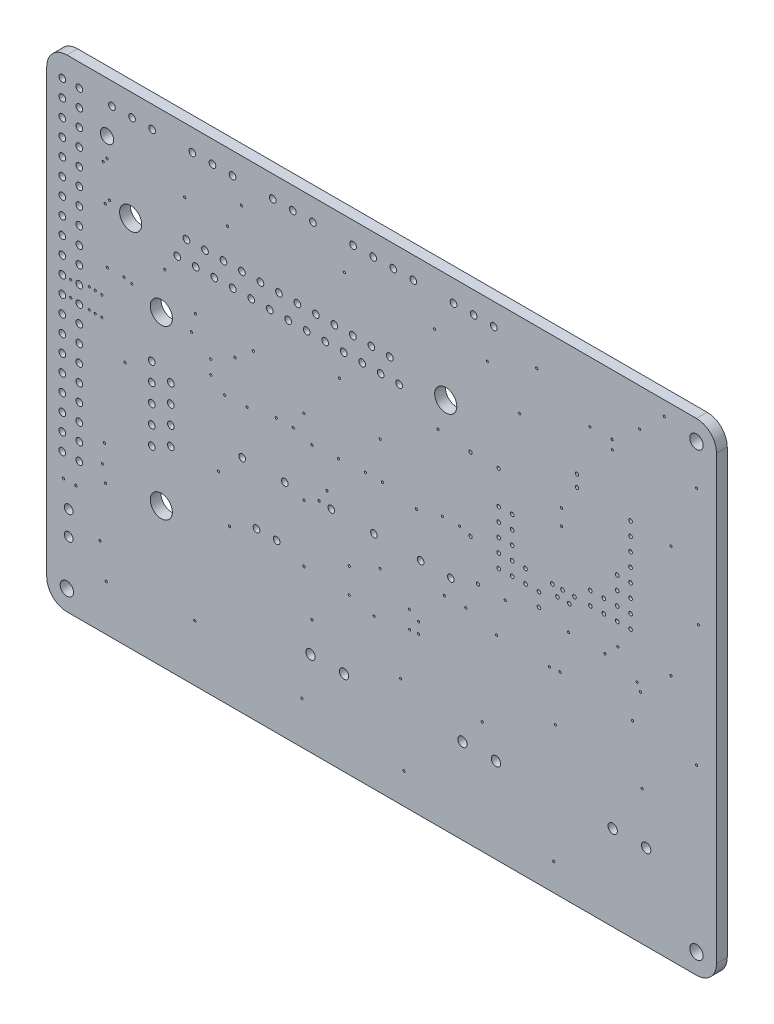
SolidWorks part; units mm, degrees
ref_plane "Front Plane" through (0, 0, 0) normal (0, 0, 1) x (1, 0, 0)
ref_plane "Top Plane" through (0, 0, 0) normal (0, 1, 0) x (1, 0, 0)
ref_plane "Right Plane" through (0, 0, 0) normal (1, 0, 0) x (0, 0, -1)
sketch "121" plane through (0, 0, 0) normal (0, 0, 1) x (1, 0, 0)
  line L0 (8, 71.008) -> (17.5, 71.008)
  line L1 (17.5, 71.008) -> (17.5, 67.524)
  line L2 (17.5, 67.524) -> (8, 67.524)
  line L3 (8, 67.524) -> (8, 71.008)
  line L4 (19.938, 71.008) -> (29.438, 71.008)
  line L5 (29.438, 71.008) -> (29.438, 67.524)
  line L6 (29.438, 67.524) -> (19.938, 67.524)
  line L7 (19.938, 67.524) -> (19.938, 71.008)
  line L8 (31.876, 71.008) -> (41.376, 71.008)
  line L9 (41.376, 71.008) -> (41.376, 67.524)
  line L10 (41.376, 67.524) -> (31.876, 67.524)
  line L11 (31.876, 67.524) -> (31.876, 71.008)
  line L12 (59.054, 71.008) -> (68.554, 71.008)
  line L13 (68.554, 71.008) -> (68.554, 67.524)
  line L14 (68.554, 67.524) -> (59.054, 67.524)
  line L15 (59.054, 67.524) -> (59.054, 71.008)
  line L16 (44.322, 71.008) -> (56.108, 71.008)
  line L17 (56.108, 71.008) -> (56.108, 67.524)
  line L18 (56.108, 67.524) -> (44.322, 67.524)
  line L19 (44.322, 67.524) -> (44.322, 71.008)
  line L20 (50.292, 67.564) -> (50.292, 68.715)
  line L21 (50.292, 69.715) -> (50.292, 70.866)
  line L22 (27.686, 34.544) -> (37.084, 34.544)
  line L23 (37.084, 34.544) -> (37.084, 29.464)
  line L24 (37.084, 29.464) -> (27.686, 29.464)
  line L25 (27.686, 29.464) -> (27.686, 34.544)
  line L26 (41.148, 34.544) -> (50.292, 34.544)
  line L27 (50.292, 34.544) -> (50.292, 29.464)
  line L28 (50.292, 29.464) -> (41.148, 29.464)
  line L29 (41.148, 29.464) -> (41.148, 34.544)
  line L30 (54.102, 34.544) -> (61.976, 34.544)
  line L31 (61.976, 34.544) -> (61.976, 29.464)
  line L32 (61.976, 29.464) -> (54.102, 29.464)
  line L33 (54.102, 29.464) -> (54.102, 34.544)
  line L34 (29.8704, 27.5336) -> (35.814, 27.5336)
  line L35 (35.814, 27.5336) -> (35.814, 22.2758)
  line L36 (35.814, 22.2758) -> (29.8704, 22.2758)
  line L37 (29.8704, 22.2758) -> (29.8704, 27.5336)
  line L38 (0.0254, 16.637) -> (5.3086, 16.637)
  line L39 (5.3086, 16.637) -> (5.3086, 6.5278)
  line L40 (5.3086, 6.5278) -> (0.0254, 6.5278)
  line L41 (0.0254, 6.5278) -> (0.0254, 16.637)
  line L42 (11.7667, 71.648) -> (11.7667, 71.2667)
  line L43 (11.7667, 71.2667) -> (11.9574, 71.2667)
  line L44 (11.9574, 71.2667) -> (12.0209, 71.3303)
  line L45 (12.0209, 71.3303) -> (12.0209, 71.5845)
  line L46 (12.0209, 71.5845) -> (11.9574, 71.648)
  line L47 (11.9574, 71.648) -> (11.7667, 71.648)
  line L48 (12.1409, 71.2667) -> (12.1409, 71.648)
  line L49 (12.1409, 71.4574) -> (12.3951, 71.4574)
  line L50 (12.3951, 71.648) -> (12.3951, 71.2667)
  line L51 (12.6422, 71.2667) -> (12.6422, 71.648)
  line L52 (12.5151, 71.648) -> (12.7693, 71.648)
  line L53 (12.8893, 71.4574) -> (13.1435, 71.4574)
  line L54 (13.2635, 71.2667) -> (13.3906, 71.2667)
  line L55 (13.3271, 71.2667) -> (13.3271, 71.648)
  line L56 (13.2635, 71.648) -> (13.3906, 71.648)
  line L57 (13.513, 71.2667) -> (13.513, 71.648)
  line L58 (13.513, 71.648) -> (13.7672, 71.2667)
  line L59 (13.7672, 71.2667) -> (13.7672, 71.648)
  line L60 (14.0143, 71.2667) -> (14.0143, 71.648)
  line L61 (13.8872, 71.648) -> (14.1414, 71.648)
  line L62 (9.2841, 70.4547) -> (9.7756, 70.4547)
  line L63 (9.5298, 70.7005) -> (9.5298, 70.209)
  line L64 (12.5903, 70.5955) -> (12.497, 70.6887)
  line L65 (12.497, 70.6887) -> (12.3106, 70.6887)
  line L66 (12.3106, 70.6887) -> (12.2174, 70.5955)
  line L67 (12.2174, 70.5955) -> (12.2174, 70.5023)
  line L68 (12.2174, 70.5023) -> (12.3106, 70.409)
  line L69 (12.3106, 70.409) -> (12.497, 70.409)
  line L70 (12.497, 70.409) -> (12.5903, 70.3158)
  line L71 (12.5903, 70.3158) -> (12.5903, 70.2226)
  line L72 (12.5903, 70.2226) -> (12.497, 70.1294)
  line L73 (12.497, 70.1294) -> (12.3106, 70.1294)
  line L74 (12.3106, 70.1294) -> (12.2174, 70.2226)
  line L75 (12.7787, 70.1294) -> (12.9651, 70.1294)
  line L76 (12.8719, 70.1294) -> (12.8719, 70.6887)
  line L77 (12.7787, 70.6887) -> (12.9651, 70.6887)
  line L78 (13.5258, 70.5955) -> (13.4326, 70.6887)
  line L79 (13.4326, 70.6887) -> (13.2461, 70.6887)
  line L80 (13.2461, 70.6887) -> (13.1529, 70.5955)
  line L81 (13.1529, 70.5955) -> (13.1529, 70.2226)
  line L82 (13.1529, 70.2226) -> (13.2461, 70.1294)
  line L83 (13.2461, 70.1294) -> (13.4326, 70.1294)
  line L84 (13.4326, 70.1294) -> (13.5258, 70.2226)
  line L85 (13.5258, 70.2226) -> (13.5258, 70.409)
  line L86 (13.5258, 70.409) -> (13.3393, 70.409)
  line L87 (15.5448, 70.4855) -> (16.3244, 70.4855)
  line L88 (23.7047, 71.648) -> (23.7047, 71.2667)
  line L89 (23.7047, 71.2667) -> (23.8954, 71.2667)
  line L90 (23.8954, 71.2667) -> (23.9589, 71.3303)
  line L91 (23.9589, 71.3303) -> (23.9589, 71.5845)
  line L92 (23.9589, 71.5845) -> (23.8954, 71.648)
  line L93 (23.8954, 71.648) -> (23.7047, 71.648)
  line L94 (24.0789, 71.2667) -> (24.0789, 71.648)
  line L95 (24.0789, 71.4574) -> (24.3331, 71.4574)
  line L96 (24.3331, 71.648) -> (24.3331, 71.2667)
  line L97 (24.5802, 71.2667) -> (24.5802, 71.648)
  line L98 (24.4531, 71.648) -> (24.7073, 71.648)
  line L99 (24.8273, 71.4574) -> (25.0815, 71.4574)
  line L100 (25.4557, 71.648) -> (25.2015, 71.648)
  line L101 (25.2015, 71.648) -> (25.2015, 71.2667)
  line L102 (25.2015, 71.2667) -> (25.4557, 71.2667)
  line L103 (25.2015, 71.4574) -> (25.3286, 71.4574)
  line L104 (25.5757, 71.648) -> (25.8299, 71.2667)
  line L105 (25.8299, 71.648) -> (25.5757, 71.2667)
  line L106 (26.077, 71.2667) -> (26.077, 71.648)
  line L107 (25.9499, 71.648) -> (26.2042, 71.648)
  line L108 (21.4761, 70.4547) -> (21.9676, 70.4547)
  line L109 (21.7218, 70.7005) -> (21.7218, 70.209)
  line L110 (24.5282, 70.5955) -> (24.435, 70.6887)
  line L111 (24.435, 70.6887) -> (24.2486, 70.6887)
  line L112 (24.2486, 70.6887) -> (24.1554, 70.5955)
  line L113 (24.1554, 70.5955) -> (24.1554, 70.5023)
  line L114 (24.1554, 70.5023) -> (24.2486, 70.409)
  line L115 (24.2486, 70.409) -> (24.435, 70.409)
  line L116 (24.435, 70.409) -> (24.5282, 70.3158)
  line L117 (24.5282, 70.3158) -> (24.5282, 70.2226)
  line L118 (24.5282, 70.2226) -> (24.435, 70.1294)
  line L119 (24.435, 70.1294) -> (24.2486, 70.1294)
  line L120 (24.2486, 70.1294) -> (24.1554, 70.2226)
  line L121 (24.7167, 70.1294) -> (24.9031, 70.1294)
  line L122 (24.8099, 70.1294) -> (24.8099, 70.6887)
  line L123 (24.7167, 70.6887) -> (24.9031, 70.6887)
  line L124 (25.4638, 70.5955) -> (25.3706, 70.6887)
  line L125 (25.3706, 70.6887) -> (25.1841, 70.6887)
  line L126 (25.1841, 70.6887) -> (25.0909, 70.5955)
  line L127 (25.0909, 70.5955) -> (25.0909, 70.2226)
  line L128 (25.0909, 70.2226) -> (25.1841, 70.1294)
  line L129 (25.1841, 70.1294) -> (25.3706, 70.1294)
  line L130 (25.3706, 70.1294) -> (25.4638, 70.2226)
  line L131 (25.4638, 70.2226) -> (25.4638, 70.409)
  line L132 (25.4638, 70.409) -> (25.2773, 70.409)
  line L133 (27.4828, 70.4855) -> (28.2624, 70.4855)
  line L134 (36.1509, 71.5845) -> (36.0874, 71.648)
  line L135 (36.0874, 71.648) -> (35.9603, 71.648)
  line L136 (35.9603, 71.648) -> (35.8967, 71.5845)
  line L137 (35.8967, 71.5845) -> (35.8967, 71.5209)
  line L138 (35.8967, 71.5209) -> (35.9603, 71.4574)
  line L139 (35.9603, 71.4574) -> (36.0874, 71.4574)
  line L140 (36.0874, 71.4574) -> (36.1509, 71.3938)
  line L141 (36.1509, 71.3938) -> (36.1509, 71.3303)
  line L142 (36.1509, 71.3303) -> (36.0874, 71.2667)
  line L143 (36.0874, 71.2667) -> (35.9603, 71.2667)
  line L144 (35.9603, 71.2667) -> (35.8967, 71.3303)
  line L145 (36.5251, 71.648) -> (36.2709, 71.648)
  line L146 (36.2709, 71.648) -> (36.2709, 71.2667)
  line L147 (36.2709, 71.2667) -> (36.5251, 71.2667)
  line L148 (36.2709, 71.4574) -> (36.398, 71.4574)
  line L149 (36.6451, 71.2667) -> (36.6451, 71.648)
  line L150 (36.6451, 71.648) -> (36.8358, 71.648)
  line L151 (36.8358, 71.648) -> (36.8993, 71.5845)
  line L152 (36.8993, 71.5845) -> (36.8993, 71.4574)
  line L153 (36.8993, 71.4574) -> (36.8358, 71.3938)
  line L154 (36.8358, 71.3938) -> (36.6451, 71.3938)
  line L155 (36.7722, 71.3938) -> (36.8993, 71.2667)
  line L156 (37.0193, 71.648) -> (37.0193, 71.3938)
  line L157 (37.0193, 71.3938) -> (37.1464, 71.2667)
  line L158 (37.1464, 71.2667) -> (37.2735, 71.3938)
  line L159 (37.2735, 71.3938) -> (37.2735, 71.648)
  line L160 (37.5842, 71.648) -> (37.4571, 71.648)
  line L161 (37.4571, 71.648) -> (37.3935, 71.5845)
  line L162 (37.3935, 71.5845) -> (37.3935, 71.3303)
  line L163 (37.3935, 71.3303) -> (37.4571, 71.2667)
  line L164 (37.4571, 71.2667) -> (37.5842, 71.2667)
  line L165 (37.5842, 71.2667) -> (37.6477, 71.3303)
  line L166 (37.6477, 71.3303) -> (37.6477, 71.5845)
  line L167 (37.6477, 71.5845) -> (37.5842, 71.648)
  line L168 (33.4141, 70.4547) -> (33.9056, 70.4547)
  line L169 (33.6598, 70.7005) -> (33.6598, 70.209)
  line L170 (35.8394, 70.1294) -> (35.8394, 70.6887)
  line L171 (35.8394, 70.6887) -> (36.119, 70.6887)
  line L172 (36.119, 70.6887) -> (36.2123, 70.5955)
  line L173 (36.2123, 70.5955) -> (36.2123, 70.409)
  line L174 (36.2123, 70.409) -> (36.119, 70.3158)
  line L175 (36.119, 70.3158) -> (35.8394, 70.3158)
  line L176 (36.4007, 70.6887) -> (36.4007, 70.1294)
  line L177 (36.4007, 70.1294) -> (36.5871, 70.3158)
  line L178 (36.5871, 70.3158) -> (36.7736, 70.1294)
  line L179 (36.7736, 70.1294) -> (36.7736, 70.6887)
  line L180 (36.962, 70.1294) -> (36.962, 70.6887)
  line L181 (36.962, 70.6887) -> (37.1484, 70.5023)
  line L182 (37.1484, 70.5023) -> (37.3349, 70.6887)
  line L183 (37.3349, 70.6887) -> (37.3349, 70.1294)
  line L184 (39.4208, 70.4855) -> (40.2004, 70.4855)
  line L185 (62.0587, 71.648) -> (62.0587, 71.2667)
  line L186 (62.0587, 71.2667) -> (62.3129, 71.2667)
  line L187 (62.4329, 71.2667) -> (62.56, 71.2667)
  line L188 (62.4965, 71.2667) -> (62.4965, 71.648)
  line L189 (62.4329, 71.648) -> (62.56, 71.648)
  line L190 (62.9366, 71.5845) -> (62.873, 71.648)
  line L191 (62.873, 71.648) -> (62.7459, 71.648)
  line L192 (62.7459, 71.648) -> (62.6824, 71.5845)
  line L193 (62.6824, 71.5845) -> (62.6824, 71.3303)
  line L194 (62.6824, 71.3303) -> (62.7459, 71.2667)
  line L195 (62.7459, 71.2667) -> (62.873, 71.2667)
  line L196 (62.873, 71.2667) -> (62.9366, 71.3303)
  line L197 (62.9366, 71.3303) -> (62.9366, 71.4574)
  line L198 (62.9366, 71.4574) -> (62.8095, 71.4574)
  line L199 (63.0566, 71.2667) -> (63.0566, 71.648)
  line L200 (63.0566, 71.4574) -> (63.3108, 71.4574)
  line L201 (63.3108, 71.648) -> (63.3108, 71.2667)
  line L202 (63.5579, 71.2667) -> (63.5579, 71.648)
  line L203 (63.4308, 71.648) -> (63.685, 71.648)
  line L204 (64.4334, 71.5845) -> (64.3699, 71.648)
  line L205 (64.3699, 71.648) -> (64.2428, 71.648)
  line L206 (64.2428, 71.648) -> (64.1792, 71.5845)
  line L207 (64.1792, 71.5845) -> (64.1792, 71.5209)
  line L208 (64.1792, 71.5209) -> (64.2428, 71.4574)
  line L209 (64.2428, 71.4574) -> (64.3699, 71.4574)
  line L210 (64.3699, 71.4574) -> (64.4334, 71.3938)
  line L211 (64.4334, 71.3938) -> (64.4334, 71.3303)
  line L212 (64.4334, 71.3303) -> (64.3699, 71.2667)
  line L213 (64.3699, 71.2667) -> (64.2428, 71.2667)
  line L214 (64.2428, 71.2667) -> (64.1792, 71.3303)
  line L215 (64.8076, 71.648) -> (64.5534, 71.648)
  line L216 (64.5534, 71.648) -> (64.5534, 71.2667)
  line L217 (64.5534, 71.2667) -> (64.8076, 71.2667)
  line L218 (64.5534, 71.4574) -> (64.6805, 71.4574)
  line L219 (64.9276, 71.2667) -> (64.9276, 71.648)
  line L220 (64.9276, 71.648) -> (65.1818, 71.2667)
  line L221 (65.1818, 71.2667) -> (65.1818, 71.648)
  line L222 (65.556, 71.5845) -> (65.4925, 71.648)
  line L223 (65.4925, 71.648) -> (65.3654, 71.648)
  line L224 (65.3654, 71.648) -> (65.3018, 71.5845)
  line L225 (65.3018, 71.5845) -> (65.3018, 71.5209)
  line L226 (65.3018, 71.5209) -> (65.3654, 71.4574)
  line L227 (65.3654, 71.4574) -> (65.4925, 71.4574)
  line L228 (65.4925, 71.4574) -> (65.556, 71.3938)
  line L229 (65.556, 71.3938) -> (65.556, 71.3303)
  line L230 (65.556, 71.3303) -> (65.4925, 71.2667)
  line L231 (65.4925, 71.2667) -> (65.3654, 71.2667)
  line L232 (65.3654, 71.2667) -> (65.3018, 71.3303)
  line L233 (65.8667, 71.648) -> (65.7396, 71.648)
  line L234 (65.7396, 71.648) -> (65.676, 71.5845)
  line L235 (65.676, 71.5845) -> (65.676, 71.3303)
  line L236 (65.676, 71.3303) -> (65.7396, 71.2667)
  line L237 (65.7396, 71.2667) -> (65.8667, 71.2667)
  line L238 (65.8667, 71.2667) -> (65.9302, 71.3303)
  line L239 (65.9302, 71.3303) -> (65.9302, 71.5845)
  line L240 (65.9302, 71.5845) -> (65.8667, 71.648)
  line L241 (66.0502, 71.2667) -> (66.0502, 71.648)
  line L242 (66.0502, 71.648) -> (66.2409, 71.648)
  line L243 (66.2409, 71.648) -> (66.3045, 71.5845)
  line L244 (66.3045, 71.5845) -> (66.3045, 71.4574)
  line L245 (66.3045, 71.4574) -> (66.2409, 71.3938)
  line L246 (66.2409, 71.3938) -> (66.0502, 71.3938)
  line L247 (66.1773, 71.3938) -> (66.3045, 71.2667)
  line L248 (60.3381, 70.4547) -> (60.8296, 70.4547)
  line L249 (60.5838, 70.7005) -> (60.5838, 70.209)
  line L250 (63.6442, 70.5955) -> (63.551, 70.6887)
  line L251 (63.551, 70.6887) -> (63.3646, 70.6887)
  line L252 (63.3646, 70.6887) -> (63.2714, 70.5955)
  line L253 (63.2714, 70.5955) -> (63.2714, 70.5023)
  line L254 (63.2714, 70.5023) -> (63.3646, 70.409)
  line L255 (63.3646, 70.409) -> (63.551, 70.409)
  line L256 (63.551, 70.409) -> (63.6442, 70.3158)
  line L257 (63.6442, 70.3158) -> (63.6442, 70.2226)
  line L258 (63.6442, 70.2226) -> (63.551, 70.1294)
  line L259 (63.551, 70.1294) -> (63.3646, 70.1294)
  line L260 (63.3646, 70.1294) -> (63.2714, 70.2226)
  line L261 (63.8327, 70.1294) -> (64.0191, 70.1294)
  line L262 (63.9259, 70.1294) -> (63.9259, 70.6887)
  line L263 (63.8327, 70.6887) -> (64.0191, 70.6887)
  line L264 (64.5798, 70.5955) -> (64.4866, 70.6887)
  line L265 (64.4866, 70.6887) -> (64.3001, 70.6887)
  line L266 (64.3001, 70.6887) -> (64.2069, 70.5955)
  line L267 (64.2069, 70.5955) -> (64.2069, 70.2226)
  line L268 (64.2069, 70.2226) -> (64.3001, 70.1294)
  line L269 (64.3001, 70.1294) -> (64.4866, 70.1294)
  line L270 (64.4866, 70.1294) -> (64.5798, 70.2226)
  line L271 (64.5798, 70.2226) -> (64.5798, 70.409)
  line L272 (64.5798, 70.409) -> (64.3933, 70.409)
  line L273 (66.5988, 70.4855) -> (67.3784, 70.4855)
  line L274 (48.5588, 71.5972) -> (48.4317, 71.5972)
  line L275 (48.4317, 71.5972) -> (48.3681, 71.5337)
  line L276 (48.3681, 71.5337) -> (48.3681, 71.2795)
  line L277 (48.3681, 71.2795) -> (48.4317, 71.2159)
  line L278 (48.4317, 71.2159) -> (48.5588, 71.2159)
  line L279 (48.5588, 71.2159) -> (48.6223, 71.2795)
  line L280 (48.6223, 71.2795) -> (48.6223, 71.5337)
  line L281 (48.6223, 71.5337) -> (48.5588, 71.5972)
  line L282 (48.7423, 71.2159) -> (48.7423, 71.5972)
  line L283 (48.7423, 71.5972) -> (48.933, 71.5972)
  line L284 (48.933, 71.5972) -> (48.9965, 71.5337)
  line L285 (48.9965, 71.5337) -> (48.9965, 71.4066)
  line L286 (48.9965, 71.4066) -> (48.933, 71.343)
  line L287 (48.933, 71.343) -> (48.7423, 71.343)
  line L288 (49.2436, 71.2159) -> (49.2436, 71.5972)
  line L289 (49.1165, 71.5972) -> (49.3707, 71.5972)
  line L290 (49.4907, 71.2159) -> (49.6178, 71.2159)
  line L291 (49.5543, 71.2159) -> (49.5543, 71.5972)
  line L292 (49.4907, 71.5972) -> (49.6178, 71.5972)
  line L293 (49.9944, 71.5337) -> (49.9309, 71.5972)
  line L294 (49.9309, 71.5972) -> (49.8037, 71.5972)
  line L295 (49.8037, 71.5972) -> (49.7402, 71.5337)
  line L296 (49.7402, 71.5337) -> (49.7402, 71.2795)
  line L297 (49.7402, 71.2795) -> (49.8037, 71.2159)
  line L298 (49.8037, 71.2159) -> (49.9309, 71.2159)
  line L299 (49.9309, 71.2159) -> (49.9944, 71.2795)
  line L300 (50.1144, 71.2159) -> (50.1144, 71.4701)
  line L301 (50.1144, 71.4701) -> (50.2415, 71.5972)
  line L302 (50.2415, 71.5972) -> (50.3686, 71.4701)
  line L303 (50.3686, 71.4701) -> (50.3686, 71.2159)
  line L304 (50.1144, 71.4066) -> (50.3686, 71.4066)
  line L305 (50.4886, 71.5972) -> (50.4886, 71.2159)
  line L306 (50.4886, 71.2159) -> (50.7428, 71.2159)
  line L307 (51.237, 71.2159) -> (51.237, 71.5972)
  line L308 (51.237, 71.5972) -> (51.4912, 71.5972)
  line L309 (51.237, 71.4066) -> (51.3641, 71.4066)
  line L310 (51.8019, 71.5972) -> (51.6748, 71.5972)
  line L311 (51.6748, 71.5972) -> (51.6112, 71.5337)
  line L312 (51.6112, 71.5337) -> (51.6112, 71.2795)
  line L313 (51.6112, 71.2795) -> (51.6748, 71.2159)
  line L314 (51.6748, 71.2159) -> (51.8019, 71.2159)
  line L315 (51.8019, 71.2159) -> (51.8654, 71.2795)
  line L316 (51.8654, 71.2795) -> (51.8654, 71.5337)
  line L317 (51.8654, 71.5337) -> (51.8019, 71.5972)
  line L318 (51.9854, 71.2159) -> (51.9854, 71.5972)
  line L319 (51.9854, 71.5972) -> (52.1761, 71.5972)
  line L320 (52.1761, 71.5972) -> (52.2396, 71.5337)
  line L321 (52.2396, 71.5337) -> (52.2396, 71.4066)
  line L322 (52.2396, 71.4066) -> (52.1761, 71.343)
  line L323 (52.1761, 71.343) -> (51.9854, 71.343)
  line L324 (52.1125, 71.343) -> (52.2396, 71.2159)
  line L325 (52.3596, 71.5972) -> (52.3596, 71.2159)
  line L326 (52.3596, 71.343) -> (52.6138, 71.5972)
  line L327 (52.4232, 71.4066) -> (52.6138, 71.2159)
  line L328 (45.3521, 70.4547) -> (45.8436, 70.4547)
  line L329 (45.5978, 70.7005) -> (45.5978, 70.209)
  line L330 (48.5648, 70.4855) -> (49.3444, 70.4855)
  line L331 (51.3461, 70.5107) -> (51.8376, 70.5107)
  line L332 (51.5918, 70.7565) -> (51.5918, 70.265)
  line L333 (54.7543, 70.5955) -> (54.661, 70.6887)
  line L334 (54.661, 70.6887) -> (54.4746, 70.6887)
  line L335 (54.4746, 70.6887) -> (54.3814, 70.5955)
  line L336 (54.3814, 70.5955) -> (54.3814, 70.5023)
  line L337 (54.3814, 70.5023) -> (54.4746, 70.409)
  line L338 (54.4746, 70.409) -> (54.661, 70.409)
  line L339 (54.661, 70.409) -> (54.7543, 70.3158)
  line L340 (54.7543, 70.3158) -> (54.7543, 70.2226)
  line L341 (54.7543, 70.2226) -> (54.661, 70.1294)
  line L342 (54.661, 70.1294) -> (54.4746, 70.1294)
  line L343 (54.4746, 70.1294) -> (54.3814, 70.2226)
  line L344 (54.9427, 70.1294) -> (55.1291, 70.1294)
  line L345 (55.0359, 70.1294) -> (55.0359, 70.6887)
  line L346 (54.9427, 70.6887) -> (55.1291, 70.6887)
  line L347 (55.6898, 70.5955) -> (55.5966, 70.6887)
  line L348 (55.5966, 70.6887) -> (55.4101, 70.6887)
  line L349 (55.4101, 70.6887) -> (55.3169, 70.5955)
  line L350 (55.3169, 70.5955) -> (55.3169, 70.2226)
  line L351 (55.3169, 70.2226) -> (55.4101, 70.1294)
  line L352 (55.4101, 70.1294) -> (55.5966, 70.1294)
  line L353 (55.5966, 70.1294) -> (55.6898, 70.2226)
  line L354 (55.6898, 70.2226) -> (55.6898, 70.409)
  line L355 (55.6898, 70.409) -> (55.5033, 70.409)
  line L356 (47.0029, 70.752) -> (46.7487, 70.752)
  line L357 (46.7487, 70.752) -> (46.7487, 70.3707)
  line L358 (46.7487, 70.3707) -> (47.0029, 70.3707)
  line L359 (46.7487, 70.5614) -> (46.8758, 70.5614)
  line L360 (47.1229, 70.3707) -> (47.1229, 70.752)
  line L361 (47.1229, 70.752) -> (47.25, 70.6249)
  line L362 (47.25, 70.6249) -> (47.3771, 70.752)
  line L363 (47.3771, 70.752) -> (47.3771, 70.3707)
  line L364 (47.4971, 70.3707) -> (47.6242, 70.3707)
  line L365 (47.5607, 70.3707) -> (47.5607, 70.752)
  line L366 (47.4971, 70.752) -> (47.6242, 70.752)
  line L367 (47.8737, 70.3707) -> (47.8737, 70.752)
  line L368 (47.7466, 70.752) -> (48.0008, 70.752)
  line L369 (52.5907, 70.3707) -> (52.5907, 70.752)
  line L370 (52.5907, 70.752) -> (52.7814, 70.752)
  line L371 (52.7814, 70.752) -> (52.8449, 70.6885)
  line L372 (52.8449, 70.6885) -> (52.8449, 70.5614)
  line L373 (52.8449, 70.5614) -> (52.7814, 70.4978)
  line L374 (52.7814, 70.4978) -> (52.5907, 70.4978)
  line L375 (52.7178, 70.4978) -> (52.8449, 70.3707)
  line L376 (53.2191, 70.752) -> (52.9649, 70.752)
  line L377 (52.9649, 70.752) -> (52.9649, 70.3707)
  line L378 (52.9649, 70.3707) -> (53.2191, 70.3707)
  line L379 (52.9649, 70.5614) -> (53.092, 70.5614)
  line L380 (53.5933, 70.6885) -> (53.5298, 70.752)
  line L381 (53.5298, 70.752) -> (53.4027, 70.752)
  line L382 (53.4027, 70.752) -> (53.3391, 70.6885)
  line L383 (53.3391, 70.6885) -> (53.3391, 70.4343)
  line L384 (53.3391, 70.4343) -> (53.4027, 70.3707)
  line L385 (53.4027, 70.3707) -> (53.5298, 70.3707)
  line L386 (53.5298, 70.3707) -> (53.5933, 70.4343)
  line L387 (31.0961, 29.8901) -> (31.0961, 30.6273)
  line L388 (31.0961, 30.2587) -> (31.5876, 30.2587)
  line L389 (31.5876, 30.6273) -> (31.5876, 29.8901)
  line L390 (32.336, 30.6273) -> (31.8445, 30.6273)
  line L391 (31.8445, 30.6273) -> (31.8445, 29.8901)
  line L392 (31.8445, 29.8901) -> (32.336, 29.8901)
  line L393 (31.8445, 30.2587) -> (32.0903, 30.2587)
  line L394 (32.5929, 29.8901) -> (32.5929, 30.3816)
  line L395 (32.5929, 30.3816) -> (32.8387, 30.6273)
  line L396 (32.8387, 30.6273) -> (33.0844, 30.3816)
  line L397 (33.0844, 30.3816) -> (33.0844, 29.8901)
  line L398 (32.5929, 30.2587) -> (33.0844, 30.2587)
  line L399 (33.5871, 29.8901) -> (33.5871, 30.6273)
  line L400 (33.3413, 30.6273) -> (33.8328, 30.6273)
  line L401 (34.9508, 31.0595) -> (35.7304, 31.0595)
  line L402 (35.3406, 31.4493) -> (35.3406, 30.6697)
  line L403 (28.7655, 31.0649) -> (29.7993, 31.0649)
  line L404 (43.7961, 30.6273) -> (43.7961, 29.8901)
  line L405 (43.7961, 29.8901) -> (44.1647, 29.8901)
  line L406 (44.1647, 29.8901) -> (44.2876, 30.013)
  line L407 (44.2876, 30.013) -> (44.2876, 30.5045)
  line L408 (44.2876, 30.5045) -> (44.1647, 30.6273)
  line L409 (44.1647, 30.6273) -> (43.7961, 30.6273)
  line L410 (45.036, 30.6273) -> (44.5445, 30.6273)
  line L411 (44.5445, 30.6273) -> (44.5445, 29.8901)
  line L412 (44.5445, 29.8901) -> (45.036, 29.8901)
  line L413 (44.5445, 30.2587) -> (44.7903, 30.2587)
  line L414 (45.2929, 29.8901) -> (45.2929, 30.6273)
  line L415 (45.2929, 30.2587) -> (45.7844, 30.2587)
  line L416 (45.7844, 30.6273) -> (45.7844, 29.8901)
  line L417 (46.0413, 30.6273) -> (46.0413, 30.013)
  line L418 (46.0413, 30.013) -> (46.1642, 29.8901)
  line L419 (46.1642, 29.8901) -> (46.41, 29.8901)
  line L420 (46.41, 29.8901) -> (46.5328, 30.013)
  line L421 (46.5328, 30.013) -> (46.5328, 30.6273)
  line L422 (46.7898, 29.8901) -> (46.7898, 30.6273)
  line L423 (46.7898, 30.6273) -> (47.0355, 30.3816)
  line L424 (47.0355, 30.3816) -> (47.2812, 30.6273)
  line L425 (47.2812, 30.6273) -> (47.2812, 29.8901)
  line L426 (48.4128, 31.0595) -> (49.1924, 31.0595)
  line L427 (48.8026, 31.4493) -> (48.8026, 30.6697)
  line L428 (42.2275, 31.0649) -> (43.2613, 31.0649)
  line L429 (57.2581, 29.8901) -> (57.2581, 30.6273)
  line L430 (57.2581, 30.6273) -> (57.7496, 30.6273)
  line L431 (57.2581, 30.2587) -> (57.5038, 30.2587)
  line L432 (58.0065, 29.8901) -> (58.0065, 30.3816)
  line L433 (58.0065, 30.3816) -> (58.2523, 30.6273)
  line L434 (58.2523, 30.6273) -> (58.498, 30.3816)
  line L435 (58.498, 30.3816) -> (58.498, 29.8901)
  line L436 (58.0065, 30.2587) -> (58.498, 30.2587)
  line L437 (58.7549, 29.8901) -> (58.7549, 30.6273)
  line L438 (58.7549, 30.6273) -> (59.2464, 29.8901)
  line L439 (59.2464, 29.8901) -> (59.2464, 30.6273)
  line L440 (59.8428, 31.0595) -> (60.6224, 31.0595)
  line L441 (60.2326, 31.4493) -> (60.2326, 30.6697)
  line L442 (55.4355, 31.0649) -> (56.4693, 31.0649)
  line L443 (34.2389, 39.0525) -> (34.2389, 39.544)
  line L444 (33.9931, 39.2982) -> (34.4846, 39.2982)
  line L445 (33.8703, 40.2924) -> (33.8703, 39.8009)
  line L446 (33.8703, 39.8009) -> (34.2389, 39.8009)
  line L447 (34.2389, 39.8009) -> (34.116, 40.0467)
  line L448 (34.116, 40.0467) -> (34.116, 40.1695)
  line L449 (34.116, 40.1695) -> (34.2389, 40.2924)
  line L450 (34.2389, 40.2924) -> (34.4846, 40.2924)
  line L451 (34.4846, 40.2924) -> (34.6075, 40.1695)
  line L452 (34.6075, 40.1695) -> (34.6075, 39.9238)
  line L453 (34.6075, 39.9238) -> (34.4846, 39.8009)
  line L454 (33.8703, 40.5493) -> (34.3618, 40.5493)
  line L455 (34.3618, 40.5493) -> (34.6075, 40.7951)
  line L456 (34.6075, 40.7951) -> (34.3618, 41.0408)
  line L457 (34.3618, 41.0408) -> (33.8703, 41.0408)
  line L458 (36.7281, 39.0271) -> (36.7281, 39.5186)
  line L459 (36.4823, 39.2728) -> (36.9738, 39.2728)
  line L460 (36.6052, 39.7755) -> (36.3595, 40.0213)
  line L461 (36.3595, 40.0213) -> (37.0967, 40.0213)
  line L462 (37.0967, 39.7755) -> (37.0967, 40.267)
  line L463 (37.0967, 41.0154) -> (37.0967, 40.5239)
  line L464 (37.0967, 40.5239) -> (36.6052, 41.0154)
  line L465 (36.6052, 41.0154) -> (36.4823, 41.0154)
  line L466 (36.4823, 41.0154) -> (36.3595, 40.8925)
  line L467 (36.3595, 40.8925) -> (36.3595, 40.6468)
  line L468 (36.3595, 40.6468) -> (36.4823, 40.5239)
  line L469 (36.3595, 41.2723) -> (36.851, 41.2723)
  line L470 (36.851, 41.2723) -> (37.0967, 41.5181)
  line L471 (37.0967, 41.5181) -> (36.851, 41.7638)
  line L472 (36.851, 41.7638) -> (36.3595, 41.7638)
  line L473 (50.0885, 38.7223) -> (50.0885, 39.2138)
  line L474 (49.8427, 38.968) -> (50.3342, 38.968)
  line L475 (49.9656, 39.4707) -> (49.7199, 39.7165)
  line L476 (49.7199, 39.7165) -> (50.4571, 39.7165)
  line L477 (50.4571, 39.4707) -> (50.4571, 39.9622)
  line L478 (50.4571, 40.7106) -> (50.4571, 40.2191)
  line L479 (50.4571, 40.2191) -> (49.9656, 40.7106)
  line L480 (49.9656, 40.7106) -> (49.8427, 40.7106)
  line L481 (49.8427, 40.7106) -> (49.7199, 40.5877)
  line L482 (49.7199, 40.5877) -> (49.7199, 40.342)
  line L483 (49.7199, 40.342) -> (49.8427, 40.2191)
  line L484 (49.7199, 40.9675) -> (50.2114, 40.9675)
  line L485 (50.2114, 40.9675) -> (50.4571, 41.2133)
  line L486 (50.4571, 41.2133) -> (50.2114, 41.459)
  line L487 (50.2114, 41.459) -> (49.7199, 41.459)
  line L488 (61.5947, 38.6461) -> (61.5947, 39.1376)
  line L489 (61.3489, 38.8918) -> (61.8404, 38.8918)
  line L490 (61.4718, 39.3945) -> (61.2261, 39.6403)
  line L491 (61.2261, 39.6403) -> (61.9633, 39.6403)
  line L492 (61.9633, 39.3945) -> (61.9633, 39.886)
  line L493 (61.9633, 40.6344) -> (61.9633, 40.1429)
  line L494 (61.9633, 40.1429) -> (61.4718, 40.6344)
  line L495 (61.4718, 40.6344) -> (61.3489, 40.6344)
  line L496 (61.3489, 40.6344) -> (61.2261, 40.5115)
  line L497 (61.2261, 40.5115) -> (61.2261, 40.2658)
  line L498 (61.2261, 40.2658) -> (61.3489, 40.1429)
  line L499 (61.2261, 40.8913) -> (61.7176, 40.8913)
  line L500 (61.7176, 40.8913) -> (61.9633, 41.1371)
  line L501 (61.9633, 41.1371) -> (61.7176, 41.3828)
  line L502 (61.7176, 41.3828) -> (61.2261, 41.3828)
  line L503 (59.0547, 38.6715) -> (59.0547, 39.163)
  line L504 (58.8089, 38.9172) -> (59.3004, 38.9172)
  line L505 (58.6861, 39.9114) -> (58.6861, 39.4199)
  line L506 (58.6861, 39.4199) -> (59.0547, 39.4199)
  line L507 (59.0547, 39.4199) -> (58.9318, 39.6657)
  line L508 (58.9318, 39.6657) -> (58.9318, 39.7885)
  line L509 (58.9318, 39.7885) -> (59.0547, 39.9114)
  line L510 (59.0547, 39.9114) -> (59.3004, 39.9114)
  line L511 (59.3004, 39.9114) -> (59.4233, 39.7885)
  line L512 (59.4233, 39.7885) -> (59.4233, 39.5428)
  line L513 (59.4233, 39.5428) -> (59.3004, 39.4199)
  line L514 (58.6861, 40.1683) -> (59.1776, 40.1683)
  line L515 (59.1776, 40.1683) -> (59.4233, 40.4141)
  line L516 (59.4233, 40.4141) -> (59.1776, 40.6598)
  line L517 (59.1776, 40.6598) -> (58.6861, 40.6598)
  line L518 (47.5231, 38.7223) -> (47.5231, 39.2138)
  line L519 (47.2773, 38.968) -> (47.7688, 38.968)
  line L520 (47.1545, 39.9622) -> (47.1545, 39.4707)
  line L521 (47.1545, 39.4707) -> (47.5231, 39.4707)
  line L522 (47.5231, 39.4707) -> (47.4002, 39.7165)
  line L523 (47.4002, 39.7165) -> (47.4002, 39.8393)
  line L524 (47.4002, 39.8393) -> (47.5231, 39.9622)
  line L525 (47.5231, 39.9622) -> (47.7688, 39.9622)
  line L526 (47.7688, 39.9622) -> (47.8917, 39.8393)
  line L527 (47.8917, 39.8393) -> (47.8917, 39.5936)
  line L528 (47.8917, 39.5936) -> (47.7688, 39.4707)
  line L529 (47.1545, 40.2191) -> (47.646, 40.2191)
  line L530 (47.646, 40.2191) -> (47.8917, 40.4649)
  line L531 (47.8917, 40.4649) -> (47.646, 40.7106)
  line L532 (47.646, 40.7106) -> (47.1545, 40.7106)
  line L533 (83.9728, 15.0575) -> (84.7524, 15.0575)
  line L534 (84.3626, 15.4473) -> (84.3626, 14.6677)
  line L535 (89.2175, 15.0629) -> (90.2513, 15.0629)
  line L536 (61.6208, 14.8035) -> (62.4004, 14.8035)
  line L537 (62.0106, 15.1933) -> (62.0106, 14.4137)
  line L538 (66.8655, 14.8089) -> (67.8993, 14.8089)
  line L539 (38.7608, 14.8035) -> (39.5404, 14.8035)
  line L540 (39.1506, 15.1933) -> (39.1506, 14.4137)
  line L541 (44.0055, 14.8089) -> (45.0393, 14.8089)
  line L542 (30.9691, 26.4611) -> (30.9691, 27.1983)
  line L543 (30.9691, 27.1983) -> (31.3377, 27.1983)
  line L544 (31.3377, 27.1983) -> (31.4606, 27.0755)
  line L545 (31.4606, 27.0755) -> (31.4606, 26.9526)
  line L546 (31.4606, 26.9526) -> (31.3377, 26.8297)
  line L547 (31.3377, 26.8297) -> (31.4606, 26.7068)
  line L548 (31.4606, 26.7068) -> (31.4606, 26.584)
  line L549 (31.4606, 26.584) -> (31.3377, 26.4611)
  line L550 (31.3377, 26.4611) -> (30.9691, 26.4611)
  line L551 (30.9691, 26.8297) -> (31.3377, 26.8297)
  line L552 (31.7175, 27.1983) -> (31.7175, 26.584)
  line L553 (31.7175, 26.584) -> (31.8404, 26.4611)
  line L554 (31.8404, 26.4611) -> (32.0861, 26.4611)
  line L555 (32.0861, 26.4611) -> (32.209, 26.584)
  line L556 (32.209, 26.584) -> (32.209, 27.1983)
  line L557 (32.4659, 27.1983) -> (32.9574, 27.1983)
  line L558 (32.9574, 27.1983) -> (32.9574, 27.0755)
  line L559 (32.9574, 27.0755) -> (32.4659, 26.584)
  line L560 (32.4659, 26.584) -> (32.4659, 26.4611)
  line L561 (32.4659, 26.4611) -> (32.9574, 26.4611)
  line L562 (33.2143, 27.1983) -> (33.7058, 27.1983)
  line L563 (33.7058, 27.1983) -> (33.7058, 27.0755)
  line L564 (33.7058, 27.0755) -> (33.2143, 26.584)
  line L565 (33.2143, 26.584) -> (33.2143, 26.4611)
  line L566 (33.2143, 26.4611) -> (33.7058, 26.4611)
  line L567 (34.4542, 27.1983) -> (33.9628, 27.1983)
  line L568 (33.9628, 27.1983) -> (33.9628, 26.4611)
  line L569 (33.9628, 26.4611) -> (34.4542, 26.4611)
  line L570 (33.9628, 26.8297) -> (34.2085, 26.8297)
  line L571 (34.7112, 26.4611) -> (34.7112, 27.1983)
  line L572 (34.7112, 27.1983) -> (35.0798, 27.1983)
  line L573 (35.0798, 27.1983) -> (35.2027, 27.0755)
  line L574 (35.2027, 27.0755) -> (35.2027, 26.8297)
  line L575 (35.2027, 26.8297) -> (35.0798, 26.7068)
  line L576 (35.0798, 26.7068) -> (34.7112, 26.7068)
  line L577 (34.9569, 26.7068) -> (35.2027, 26.4611)
  line L578 (30.8737, 23.2163) -> (31.9075, 23.2163)
  line L579 (33.7316, 23.1347) -> (34.5112, 23.1347)
  line L580 (34.1214, 23.5245) -> (34.1214, 22.7449)
  line L581 (33.7062, 23.1347) -> (34.4858, 23.1347)
  line L582 (34.096, 23.5245) -> (34.096, 22.7449)
  line L583 (1.2757, 9.1251) -> (0.5385, 9.1251)
  line L584 (0.5385, 9.1251) -> (0.5385, 9.4937)
  line L585 (0.5385, 9.4937) -> (0.6613, 9.6166)
  line L586 (0.6613, 9.6166) -> (0.9071, 9.6166)
  line L587 (0.9071, 9.6166) -> (1.03, 9.4937)
  line L588 (1.03, 9.4937) -> (1.03, 9.1251)
  line L589 (0.5385, 10.2421) -> (0.5385, 9.9964)
  line L590 (0.5385, 9.9964) -> (0.6613, 9.8735)
  line L591 (0.6613, 9.8735) -> (1.1528, 9.8735)
  line L592 (1.1528, 9.8735) -> (1.2757, 9.9964)
  line L593 (1.2757, 9.9964) -> (1.2757, 10.2421)
  line L594 (1.2757, 10.2421) -> (1.1528, 10.365)
  line L595 (1.1528, 10.365) -> (0.6613, 10.365)
  line L596 (0.6613, 10.365) -> (0.5385, 10.2421)
  line L597 (0.5385, 10.6219) -> (1.2757, 10.6219)
  line L598 (1.2757, 10.6219) -> (1.03, 10.8677)
  line L599 (1.03, 10.8677) -> (1.2757, 11.1134)
  line L600 (1.2757, 11.1134) -> (0.5385, 11.1134)
  line L601 (0.5385, 11.8618) -> (0.5385, 11.3703)
  line L602 (0.5385, 11.3703) -> (1.2757, 11.3703)
  line L603 (1.2757, 11.3703) -> (1.2757, 11.8618)
  line L604 (0.9071, 11.3703) -> (0.9071, 11.6161)
  line L605 (1.2757, 12.1188) -> (0.5385, 12.1188)
  line L606 (0.5385, 12.1188) -> (0.5385, 12.4874)
  line L607 (0.5385, 12.4874) -> (0.6613, 12.6102)
  line L608 (0.6613, 12.6102) -> (0.9071, 12.6102)
  line L609 (0.9071, 12.6102) -> (1.03, 12.4874)
  line L610 (1.03, 12.4874) -> (1.03, 12.1188)
  line L611 (1.03, 12.3645) -> (1.2757, 12.6102)
  line L612 (1.2757, 13.6156) -> (1.2757, 13.8613)
  line L613 (1.2757, 13.7385) -> (0.5385, 13.7385)
  line L614 (0.5385, 13.6156) -> (0.5385, 13.8613)
  line L615 (1.2757, 14.1145) -> (0.5385, 14.1145)
  line L616 (0.5385, 14.1145) -> (1.2757, 14.606)
  line L617 (1.2757, 14.606) -> (0.5385, 14.606)
  line L618 (1.8669, 15.7229) -> (2.3584, 15.7229)
  line L619 (2.1126, 15.9687) -> (2.1126, 15.4772)
  line L620 (2.6153, 15.8458) -> (2.8611, 16.0915)
  line L621 (2.8611, 16.0915) -> (2.8611, 15.3543)
  line L622 (2.6153, 15.3543) -> (3.1068, 15.3543)
  line L623 (3.8552, 15.3543) -> (3.3637, 15.3543)
  line L624 (3.3637, 15.3543) -> (3.8552, 15.8458)
  line L625 (3.8552, 15.8458) -> (3.8552, 15.9687)
  line L626 (3.8552, 15.9687) -> (3.7323, 16.0915)
  line L627 (3.7323, 16.0915) -> (3.4866, 16.0915)
  line L628 (3.4866, 16.0915) -> (3.3637, 15.9687)
  line L629 (4.1121, 16.0915) -> (4.1121, 15.6)
  line L630 (4.1121, 15.6) -> (4.3579, 15.3543)
  line L631 (4.3579, 15.3543) -> (4.6036, 15.6)
  line L632 (4.6036, 15.6) -> (4.6036, 16.0915)
  line L633 (2.6124, 7.5105) -> (2.4895, 7.6333)
  line L634 (2.4895, 7.6333) -> (2.2438, 7.6333)
  line L635 (2.2438, 7.6333) -> (2.1209, 7.5105)
  line L636 (2.1209, 7.5105) -> (2.1209, 7.019)
  line L637 (2.1209, 7.019) -> (2.2438, 6.8961)
  line L638 (2.2438, 6.8961) -> (2.4895, 6.8961)
  line L639 (2.4895, 6.8961) -> (2.6124, 7.019)
  line L640 (2.6124, 7.019) -> (2.6124, 7.2647)
  line L641 (2.6124, 7.2647) -> (2.3666, 7.2647)
  line L642 (2.8693, 6.8961) -> (2.8693, 7.6333)
  line L643 (2.8693, 7.6333) -> (3.3608, 6.8961)
  line L644 (3.3608, 6.8961) -> (3.3608, 7.6333)
  line L645 (3.6177, 7.6333) -> (3.6177, 6.8961)
  line L646 (3.6177, 6.8961) -> (3.9863, 6.8961)
  line L647 (3.9863, 6.8961) -> (4.1092, 7.019)
  line L648 (4.1092, 7.019) -> (4.1092, 7.5105)
  line L649 (4.1092, 7.5105) -> (3.9863, 7.6333)
  line L650 (3.9863, 7.6333) -> (3.6177, 7.6333)
  arc A0 (17.5, 70.983) -> (17.5, 71.033) centre (17.5, 71.008) ccw
  arc A1 (8, 71.033) -> (8, 70.983) centre (8, 71.008) ccw
  arc A2 (17.475, 67.524) -> (17.525, 67.524) centre (17.5, 67.524) ccw
  arc A3 (17.525, 71.008) -> (17.475, 71.008) centre (17.5, 71.008) ccw
  arc A4 (8, 67.549) -> (8, 67.499) centre (8, 67.524) ccw
  arc A5 (17.5, 67.499) -> (17.5, 67.549) centre (17.5, 67.524) ccw
  arc A6 (8.025, 71.008) -> (7.975, 71.008) centre (8, 71.008) ccw
  arc A7 (7.975, 67.524) -> (8.025, 67.524) centre (8, 67.524) ccw
  arc A8 (29.438, 70.983) -> (29.438, 71.033) centre (29.438, 71.008) ccw
  arc A9 (19.938, 71.033) -> (19.938, 70.983) centre (19.938, 71.008) ccw
  arc A10 (29.413, 67.524) -> (29.463, 67.524) centre (29.438, 67.524) ccw
  arc A11 (29.463, 71.008) -> (29.413, 71.008) centre (29.438, 71.008) ccw
  arc A12 (19.938, 67.549) -> (19.938, 67.499) centre (19.938, 67.524) ccw
  arc A13 (29.438, 67.499) -> (29.438, 67.549) centre (29.438, 67.524) ccw
  arc A14 (19.963, 71.008) -> (19.913, 71.008) centre (19.938, 71.008) ccw
  arc A15 (19.913, 67.524) -> (19.963, 67.524) centre (19.938, 67.524) ccw
  arc A16 (41.376, 70.983) -> (41.376, 71.033) centre (41.376, 71.008) ccw
  arc A17 (31.876, 71.033) -> (31.876, 70.983) centre (31.876, 71.008) ccw
  arc A18 (41.351, 67.524) -> (41.401, 67.524) centre (41.376, 67.524) ccw
  arc A19 (41.401, 71.008) -> (41.351, 71.008) centre (41.376, 71.008) ccw
  arc A20 (31.876, 67.549) -> (31.876, 67.499) centre (31.876, 67.524) ccw
  arc A21 (41.376, 67.499) -> (41.376, 67.549) centre (41.376, 67.524) ccw
  arc A22 (31.901, 71.008) -> (31.851, 71.008) centre (31.876, 71.008) ccw
  arc A23 (31.851, 67.524) -> (31.901, 67.524) centre (31.876, 67.524) ccw
  arc A24 (68.554, 70.983) -> (68.554, 71.033) centre (68.554, 71.008) ccw
  arc A25 (59.054, 71.033) -> (59.054, 70.983) centre (59.054, 71.008) ccw
  arc A26 (68.529, 67.524) -> (68.579, 67.524) centre (68.554, 67.524) ccw
  arc A27 (68.579, 71.008) -> (68.529, 71.008) centre (68.554, 71.008) ccw
  arc A28 (59.054, 67.549) -> (59.054, 67.499) centre (59.054, 67.524) ccw
  arc A29 (68.554, 67.499) -> (68.554, 67.549) centre (68.554, 67.524) ccw
  arc A30 (59.079, 71.008) -> (59.029, 71.008) centre (59.054, 71.008) ccw
  arc A31 (59.029, 67.524) -> (59.079, 67.524) centre (59.054, 67.524) ccw
  arc A32 (56.108, 70.983) -> (56.108, 71.033) centre (56.108, 71.008) ccw
  arc A33 (44.322, 71.033) -> (44.322, 70.983) centre (44.322, 71.008) ccw
  arc A34 (56.083, 67.524) -> (56.133, 67.524) centre (56.108, 67.524) ccw
  arc A35 (56.133, 71.008) -> (56.083, 71.008) centre (56.108, 71.008) ccw
  arc A36 (44.322, 67.549) -> (44.322, 67.499) centre (44.322, 67.524) ccw
  arc A37 (56.108, 67.499) -> (56.108, 67.549) centre (56.108, 67.524) ccw
  arc A38 (44.347, 71.008) -> (44.297, 71.008) centre (44.322, 71.008) ccw
  arc A39 (44.297, 67.524) -> (44.347, 67.524) centre (44.322, 67.524) ccw
  arc A40 (50.317, 68.715) -> (50.267, 68.715) centre (50.292, 68.715) ccw
  arc A41 (50.267, 67.564) -> (50.317, 67.564) centre (50.292, 67.564) ccw
  arc A42 (50.317, 70.866) -> (50.267, 70.866) centre (50.292, 70.866) ccw
  arc A43 (50.267, 69.715) -> (50.317, 69.715) centre (50.292, 69.715) ccw
  arc A44 (37.084, 34.519) -> (37.084, 34.569) centre (37.084, 34.544) ccw
  arc A45 (27.686, 34.569) -> (27.686, 34.519) centre (27.686, 34.544) ccw
  arc A46 (37.059, 29.464) -> (37.109, 29.464) centre (37.084, 29.464) ccw
  arc A47 (37.109, 34.544) -> (37.059, 34.544) centre (37.084, 34.544) ccw
  arc A48 (27.686, 29.489) -> (27.686, 29.439) centre (27.686, 29.464) ccw
  arc A49 (37.084, 29.439) -> (37.084, 29.489) centre (37.084, 29.464) ccw
  arc A50 (27.711, 34.544) -> (27.661, 34.544) centre (27.686, 34.544) ccw
  arc A51 (27.661, 29.464) -> (27.711, 29.464) centre (27.686, 29.464) ccw
  arc A52 (50.292, 34.519) -> (50.292, 34.569) centre (50.292, 34.544) ccw
  arc A53 (41.148, 34.569) -> (41.148, 34.519) centre (41.148, 34.544) ccw
  arc A54 (50.267, 29.464) -> (50.317, 29.464) centre (50.292, 29.464) ccw
  arc A55 (50.317, 34.544) -> (50.267, 34.544) centre (50.292, 34.544) ccw
  arc A56 (41.148, 29.489) -> (41.148, 29.439) centre (41.148, 29.464) ccw
  arc A57 (50.292, 29.439) -> (50.292, 29.489) centre (50.292, 29.464) ccw
  arc A58 (41.173, 34.544) -> (41.123, 34.544) centre (41.148, 34.544) ccw
  arc A59 (41.123, 29.464) -> (41.173, 29.464) centre (41.148, 29.464) ccw
  arc A60 (61.976, 34.519) -> (61.976, 34.569) centre (61.976, 34.544) ccw
  arc A61 (54.102, 34.569) -> (54.102, 34.519) centre (54.102, 34.544) ccw
  arc A62 (61.951, 29.464) -> (62.001, 29.464) centre (61.976, 29.464) ccw
  arc A63 (62.001, 34.544) -> (61.951, 34.544) centre (61.976, 34.544) ccw
  arc A64 (54.102, 29.489) -> (54.102, 29.439) centre (54.102, 29.464) ccw
  arc A65 (61.976, 29.439) -> (61.976, 29.489) centre (61.976, 29.464) ccw
  arc A66 (54.127, 34.544) -> (54.077, 34.544) centre (54.102, 34.544) ccw
  arc A67 (54.077, 29.464) -> (54.127, 29.464) centre (54.102, 29.464) ccw
  arc A68 (35.814, 27.5086) -> (35.814, 27.5586) centre (35.814, 27.5336) ccw
  arc A69 (29.8704, 27.5586) -> (29.8704, 27.5086) centre (29.8704, 27.5336) ccw
  arc A70 (35.789, 22.2758) -> (35.839, 22.2758) centre (35.814, 22.2758) ccw
  arc A71 (35.839, 27.5336) -> (35.789, 27.5336) centre (35.814, 27.5336) ccw
  arc A72 (29.8704, 22.3008) -> (29.8704, 22.2508) centre (29.8704, 22.2758) ccw
  arc A73 (35.814, 22.2508) -> (35.814, 22.3008) centre (35.814, 22.2758) ccw
  arc A74 (29.8954, 27.5336) -> (29.8454, 27.5336) centre (29.8704, 27.5336) ccw
  arc A75 (29.8454, 22.2758) -> (29.8954, 22.2758) centre (29.8704, 22.2758) ccw
  arc A76 (5.3086, 16.612) -> (5.3086, 16.662) centre (5.3086, 16.637) ccw
  arc A77 (0.0254, 16.662) -> (0.0254, 16.612) centre (0.0254, 16.637) ccw
  arc A78 (5.2836, 6.5278) -> (5.3336, 6.5278) centre (5.3086, 6.5278) ccw
  arc A79 (5.3336, 16.637) -> (5.2836, 16.637) centre (5.3086, 16.637) ccw
  arc A80 (0.0254, 6.5528) -> (0.0254, 6.5028) centre (0.0254, 6.5278) ccw
  arc A81 (5.3086, 6.5028) -> (5.3086, 6.5528) centre (5.3086, 6.5278) ccw
  arc A82 (0.0504, 16.637) -> (0.0004, 16.637) centre (0.0254, 16.637) ccw
  arc A83 (0.0004, 6.5278) -> (0.0504, 6.5278) centre (0.0254, 6.5278) ccw
  arc A84 (11.7604, 71.2667) -> (11.773, 71.2667) centre (11.7667, 71.2667) ccw
  arc A85 (11.773, 71.648) -> (11.7604, 71.648) centre (11.7667, 71.648) ccw
  arc A86 (11.9574, 71.2604) -> (11.9574, 71.273) centre (11.9574, 71.2667) ccw
  arc A87 (11.7667, 71.273) -> (11.7667, 71.2604) centre (11.7667, 71.2667) ccw
  arc A88 (12.0254, 71.3258) -> (12.0164, 71.3347) centre (12.0209, 71.3303) ccw
  arc A89 (11.9529, 71.2712) -> (11.9619, 71.2622) centre (11.9574, 71.2667) ccw
  arc A90 (12.0273, 71.5845) -> (12.0146, 71.5845) centre (12.021, 71.5845) ccw
  arc A91 (12.0146, 71.3303) -> (12.0273, 71.3303) centre (12.021, 71.3303) ccw
  arc A92 (11.9619, 71.6525) -> (11.9529, 71.6435) centre (11.9574, 71.648) ccw
  arc A93 (12.0164, 71.58) -> (12.0254, 71.589) centre (12.0209, 71.5845) ccw
  arc A94 (11.7667, 71.6544) -> (11.7667, 71.6417) centre (11.7667, 71.648) ccw
  arc A95 (11.9574, 71.6417) -> (11.9574, 71.6544) centre (11.9574, 71.648) ccw
  arc A96 (12.1473, 71.648) -> (12.1346, 71.648) centre (12.141, 71.648) ccw
  arc A97 (12.1346, 71.2667) -> (12.1473, 71.2667) centre (12.141, 71.2667) ccw
  arc A98 (12.3951, 71.451) -> (12.3951, 71.4637) centre (12.3951, 71.4574) ccw
  arc A99 (12.1409, 71.4637) -> (12.1409, 71.451) centre (12.1409, 71.4574) ccw
  arc A100 (12.3888, 71.2667) -> (12.4015, 71.2667) centre (12.3952, 71.2667) ccw
  arc A101 (12.4015, 71.648) -> (12.3888, 71.648) centre (12.3952, 71.648) ccw
  arc A102 (12.6486, 71.648) -> (12.6359, 71.648) centre (12.6423, 71.648) ccw
  arc A103 (12.6359, 71.2667) -> (12.6486, 71.2667) centre (12.6423, 71.2667) ccw
  arc A104 (12.7693, 71.6417) -> (12.7693, 71.6544) centre (12.7693, 71.648) ccw
  arc A105 (12.5151, 71.6544) -> (12.5151, 71.6417) centre (12.5151, 71.648) ccw
  arc A106 (13.1435, 71.451) -> (13.1435, 71.4637) centre (13.1435, 71.4574) ccw
  arc A107 (12.8893, 71.4637) -> (12.8893, 71.451) centre (12.8893, 71.4574) ccw
  arc A108 (13.3906, 71.2604) -> (13.3906, 71.273) centre (13.3906, 71.2667) ccw
  arc A109 (13.2635, 71.273) -> (13.2635, 71.2604) centre (13.2635, 71.2667) ccw
  arc A110 (13.3334, 71.648) -> (13.3207, 71.648) centre (13.327, 71.648) ccw
  arc A111 (13.3207, 71.2667) -> (13.3334, 71.2667) centre (13.327, 71.2667) ccw
  arc A112 (13.3906, 71.6417) -> (13.3906, 71.6544) centre (13.3906, 71.648) ccw
  arc A113 (13.2635, 71.6544) -> (13.2635, 71.6417) centre (13.2635, 71.648) ccw
  arc A114 (13.5193, 71.648) -> (13.5066, 71.648) centre (13.513, 71.648) ccw
  arc A115 (13.5066, 71.2667) -> (13.5193, 71.2667) centre (13.513, 71.2667) ccw
  arc A116 (13.7619, 71.2632) -> (13.7725, 71.2702) centre (13.7672, 71.2667) ccw
  arc A117 (13.5183, 71.6515) -> (13.5077, 71.6445) centre (13.513, 71.648) ccw
  arc A118 (13.7736, 71.648) -> (13.7609, 71.648) centre (13.7673, 71.648) ccw
  arc A119 (13.7609, 71.2667) -> (13.7736, 71.2667) centre (13.7673, 71.2667) ccw
  arc A120 (14.0207, 71.648) -> (14.008, 71.648) centre (14.0144, 71.648) ccw
  arc A121 (14.008, 71.2667) -> (14.0207, 71.2667) centre (14.0144, 71.2667) ccw
  arc A122 (14.1414, 71.6417) -> (14.1414, 71.6544) centre (14.1414, 71.648) ccw
  arc A123 (13.8872, 71.6544) -> (13.8872, 71.6417) centre (13.8872, 71.648) ccw
  arc A124 (9.7756, 70.4357) -> (9.7756, 70.4738) centre (9.7756, 70.4548) ccw
  arc A125 (9.2841, 70.4738) -> (9.2841, 70.4357) centre (9.2841, 70.4548) ccw
  arc A126 (9.5108, 70.209) -> (9.5489, 70.209) centre (9.5298, 70.209) ccw
  arc A127 (9.5489, 70.7005) -> (9.5108, 70.7005) centre (9.5298, 70.7005) ccw
  arc A128 (12.506, 70.6977) -> (12.4881, 70.6797) centre (12.497, 70.6887) ccw
  arc A129 (12.5813, 70.5865) -> (12.5992, 70.6044) centre (12.5903, 70.5954) ccw
  arc A130 (12.3106, 70.7014) -> (12.3106, 70.676) centre (12.3106, 70.6887) ccw
  arc A131 (12.497, 70.676) -> (12.497, 70.7014) centre (12.497, 70.6887) ccw
  arc A132 (12.2084, 70.6044) -> (12.2264, 70.5865) centre (12.2174, 70.5954) ccw
  arc A133 (12.3196, 70.6797) -> (12.3016, 70.6977) centre (12.3106, 70.6887) ccw
  arc A134 (12.2047, 70.5023) -> (12.2301, 70.5023) centre (12.2174, 70.5023) ccw
  arc A135 (12.2301, 70.5955) -> (12.2047, 70.5955) centre (12.2174, 70.5955) ccw
  arc A136 (12.3016, 70.4001) -> (12.3196, 70.418) centre (12.3106, 70.4091) ccw
  arc A137 (12.2264, 70.5112) -> (12.2084, 70.4933) centre (12.2174, 70.5023) ccw
  arc A138 (12.497, 70.3963) -> (12.497, 70.4217) centre (12.497, 70.409) ccw
  arc A139 (12.3106, 70.4217) -> (12.3106, 70.3963) centre (12.3106, 70.409) ccw
  arc A140 (12.5813, 70.3068) -> (12.5992, 70.3248) centre (12.5903, 70.3158) ccw
  arc A141 (12.506, 70.418) -> (12.4881, 70.4001) centre (12.497, 70.4091) ccw
  arc A142 (12.5776, 70.2226) -> (12.603, 70.2226) centre (12.5903, 70.2226) ccw
  arc A143 (12.603, 70.3158) -> (12.5776, 70.3158) centre (12.5903, 70.3158) ccw
  arc A144 (12.4881, 70.1384) -> (12.506, 70.1204) centre (12.497, 70.1294) ccw
  arc A145 (12.5992, 70.2136) -> (12.5813, 70.2316) centre (12.5903, 70.2226) ccw
  arc A146 (12.3106, 70.1421) -> (12.3106, 70.1167) centre (12.3106, 70.1294) ccw
  arc A147 (12.497, 70.1167) -> (12.497, 70.1421) centre (12.497, 70.1294) ccw
  arc A148 (12.2264, 70.2316) -> (12.2084, 70.2136) centre (12.2174, 70.2226) ccw
  arc A149 (12.3016, 70.1204) -> (12.3196, 70.1384) centre (12.3106, 70.1294) ccw
  arc A150 (12.9651, 70.1167) -> (12.9651, 70.1421) centre (12.9651, 70.1294) ccw
  arc A151 (12.7787, 70.1421) -> (12.7787, 70.1167) centre (12.7787, 70.1294) ccw
  arc A152 (12.8846, 70.6887) -> (12.8592, 70.6887) centre (12.8719, 70.6887) ccw
  arc A153 (12.8592, 70.1294) -> (12.8846, 70.1294) centre (12.8719, 70.1294) ccw
  arc A154 (12.9651, 70.676) -> (12.9651, 70.7014) centre (12.9651, 70.6887) ccw
  arc A155 (12.7787, 70.7014) -> (12.7787, 70.676) centre (12.7787, 70.6887) ccw
  arc A156 (13.4415, 70.6977) -> (13.4236, 70.6797) centre (13.4326, 70.6887) ccw
  arc A157 (13.5168, 70.5865) -> (13.5347, 70.6044) centre (13.5258, 70.5954) ccw
  arc A158 (13.2461, 70.7014) -> (13.2461, 70.676) centre (13.2461, 70.6887) ccw
  arc A159 (13.4326, 70.676) -> (13.4326, 70.7014) centre (13.4326, 70.6887) ccw
  arc A160 (13.1439, 70.6044) -> (13.1619, 70.5865) centre (13.1529, 70.5954) ccw
  arc A161 (13.2551, 70.6797) -> (13.2371, 70.6977) centre (13.2461, 70.6887) ccw
  arc A162 (13.1402, 70.2226) -> (13.1656, 70.2226) centre (13.1529, 70.2226) ccw
  arc A163 (13.1656, 70.5955) -> (13.1402, 70.5955) centre (13.1529, 70.5955) ccw
  arc A164 (13.2371, 70.1204) -> (13.2551, 70.1384) centre (13.2461, 70.1294) ccw
  arc A165 (13.1619, 70.2316) -> (13.1439, 70.2136) centre (13.1529, 70.2226) ccw
  arc A166 (13.4326, 70.1167) -> (13.4326, 70.1421) centre (13.4326, 70.1294) ccw
  arc A167 (13.2461, 70.1421) -> (13.2461, 70.1167) centre (13.2461, 70.1294) ccw
  arc A168 (13.5347, 70.2136) -> (13.5168, 70.2316) centre (13.5258, 70.2226) ccw
  arc A169 (13.4236, 70.1384) -> (13.4415, 70.1204) centre (13.4326, 70.1294) ccw
  arc A170 (13.5385, 70.409) -> (13.5131, 70.409) centre (13.5258, 70.409) ccw
  arc A171 (13.5131, 70.2226) -> (13.5385, 70.2226) centre (13.5258, 70.2226) ccw
  arc A172 (13.3393, 70.4217) -> (13.3393, 70.3963) centre (13.3393, 70.409) ccw
  arc A173 (13.5258, 70.3963) -> (13.5258, 70.4217) centre (13.5258, 70.409) ccw
  arc A174 (16.3244, 70.4601) -> (16.3244, 70.5109) centre (16.3244, 70.4855) ccw
  arc A175 (15.5448, 70.5109) -> (15.5448, 70.4601) centre (15.5448, 70.4855) ccw
  arc A176 (23.6984, 71.2667) -> (23.7111, 71.2667) centre (23.7048, 71.2667) ccw
  arc A177 (23.7111, 71.648) -> (23.6984, 71.648) centre (23.7048, 71.648) ccw
  arc A178 (23.8954, 71.2604) -> (23.8954, 71.273) centre (23.8954, 71.2667) ccw
  arc A179 (23.7047, 71.273) -> (23.7047, 71.2604) centre (23.7047, 71.2667) ccw
  arc A180 (23.9634, 71.3258) -> (23.9544, 71.3347) centre (23.9589, 71.3303) ccw
  arc A181 (23.8909, 71.2712) -> (23.8999, 71.2622) centre (23.8954, 71.2667) ccw
  arc A182 (23.9653, 71.5845) -> (23.9526, 71.5845) centre (23.9589, 71.5845) ccw
  arc A183 (23.9526, 71.3303) -> (23.9653, 71.3303) centre (23.9589, 71.3303) ccw
  arc A184 (23.8999, 71.6525) -> (23.8909, 71.6435) centre (23.8954, 71.648) ccw
  arc A185 (23.9544, 71.58) -> (23.9634, 71.589) centre (23.9589, 71.5845) ccw
  arc A186 (23.7047, 71.6544) -> (23.7047, 71.6417) centre (23.7047, 71.648) ccw
  arc A187 (23.8954, 71.6417) -> (23.8954, 71.6544) centre (23.8954, 71.648) ccw
  arc A188 (24.0853, 71.648) -> (24.0726, 71.648) centre (24.079, 71.648) ccw
  arc A189 (24.0726, 71.2667) -> (24.0853, 71.2667) centre (24.079, 71.2667) ccw
  arc A190 (24.3331, 71.451) -> (24.3331, 71.4637) centre (24.3331, 71.4574) ccw
  arc A191 (24.0789, 71.4637) -> (24.0789, 71.451) centre (24.0789, 71.4574) ccw
  arc A192 (24.3268, 71.2667) -> (24.3395, 71.2667) centre (24.3331, 71.2667) ccw
  arc A193 (24.3395, 71.648) -> (24.3268, 71.648) centre (24.3331, 71.648) ccw
  arc A194 (24.5866, 71.648) -> (24.5739, 71.648) centre (24.5802, 71.648) ccw
  arc A195 (24.5739, 71.2667) -> (24.5866, 71.2667) centre (24.5802, 71.2667) ccw
  arc A196 (24.7073, 71.6417) -> (24.7073, 71.6544) centre (24.7073, 71.648) ccw
  arc A197 (24.4531, 71.6544) -> (24.4531, 71.6417) centre (24.4531, 71.648) ccw
  arc A198 (25.0815, 71.451) -> (25.0815, 71.4637) centre (25.0815, 71.4574) ccw
  arc A199 (24.8273, 71.4637) -> (24.8273, 71.451) centre (24.8273, 71.4574) ccw
  arc A200 (25.2015, 71.6544) -> (25.2015, 71.6417) centre (25.2015, 71.648) ccw
  arc A201 (25.4557, 71.6417) -> (25.4557, 71.6544) centre (25.4557, 71.648) ccw
  arc A202 (25.1952, 71.2667) -> (25.2079, 71.2667) centre (25.2016, 71.2667) ccw
  arc A203 (25.2079, 71.648) -> (25.1952, 71.648) centre (25.2016, 71.648) ccw
  arc A204 (25.4557, 71.2604) -> (25.4557, 71.273) centre (25.4557, 71.2667) ccw
  arc A205 (25.2015, 71.273) -> (25.2015, 71.2604) centre (25.2015, 71.2667) ccw
  arc A206 (25.3286, 71.451) -> (25.3286, 71.4637) centre (25.3286, 71.4574) ccw
  arc A207 (25.2015, 71.4637) -> (25.2015, 71.451) centre (25.2015, 71.4574) ccw
  arc A208 (25.8247, 71.2632) -> (25.8352, 71.2702) centre (25.83, 71.2667) ccw
  arc A209 (25.581, 71.6515) -> (25.5704, 71.6445) centre (25.5757, 71.648) ccw
  arc A210 (25.5704, 71.2702) -> (25.581, 71.2632) centre (25.5757, 71.2667) ccw
  arc A211 (25.8352, 71.6445) -> (25.8247, 71.6515) centre (25.83, 71.648) ccw
  arc A212 (26.0834, 71.648) -> (26.0707, 71.648) centre (26.077, 71.648) ccw
  arc A213 (26.0707, 71.2667) -> (26.0834, 71.2667) centre (26.077, 71.2667) ccw
  arc A214 (26.2042, 71.6417) -> (26.2042, 71.6544) centre (26.2042, 71.648) ccw
  arc A215 (25.9499, 71.6544) -> (25.9499, 71.6417) centre (25.9499, 71.648) ccw
  arc A216 (21.9676, 70.4357) -> (21.9676, 70.4738) centre (21.9676, 70.4548) ccw
  arc A217 (21.4761, 70.4738) -> (21.4761, 70.4357) centre (21.4761, 70.4548) ccw
  arc A218 (21.7028, 70.209) -> (21.7409, 70.209) centre (21.7218, 70.209) ccw
  arc A219 (21.7409, 70.7005) -> (21.7028, 70.7005) centre (21.7218, 70.7005) ccw
  arc A220 (24.444, 70.6977) -> (24.4261, 70.6797) centre (24.4351, 70.6887) ccw
  arc A221 (24.5193, 70.5865) -> (24.5372, 70.6044) centre (24.5282, 70.5954) ccw
  arc A222 (24.2486, 70.7014) -> (24.2486, 70.676) centre (24.2486, 70.6887) ccw
  arc A223 (24.435, 70.676) -> (24.435, 70.7014) centre (24.435, 70.6887) ccw
  arc A224 (24.1464, 70.6044) -> (24.1644, 70.5865) centre (24.1554, 70.5954) ccw
  arc A225 (24.2576, 70.6797) -> (24.2396, 70.6977) centre (24.2486, 70.6887) ccw
  arc A226 (24.1427, 70.5023) -> (24.1681, 70.5023) centre (24.1554, 70.5023) ccw
  arc A227 (24.1681, 70.5955) -> (24.1427, 70.5955) centre (24.1554, 70.5955) ccw
  arc A228 (24.2396, 70.4001) -> (24.2576, 70.418) centre (24.2486, 70.4091) ccw
  arc A229 (24.1644, 70.5112) -> (24.1464, 70.4933) centre (24.1554, 70.5023) ccw
  arc A230 (24.435, 70.3963) -> (24.435, 70.4217) centre (24.435, 70.409) ccw
  arc A231 (24.2486, 70.4217) -> (24.2486, 70.3963) centre (24.2486, 70.409) ccw
  arc A232 (24.5193, 70.3068) -> (24.5372, 70.3248) centre (24.5282, 70.3158) ccw
  arc A233 (24.444, 70.418) -> (24.4261, 70.4001) centre (24.4351, 70.4091) ccw
  arc A234 (24.5156, 70.2226) -> (24.5409, 70.2226) centre (24.5282, 70.2226) ccw
  arc A235 (24.5409, 70.3158) -> (24.5156, 70.3158) centre (24.5282, 70.3158) ccw
  arc A236 (24.4261, 70.1384) -> (24.444, 70.1204) centre (24.4351, 70.1294) ccw
  arc A237 (24.5372, 70.2136) -> (24.5193, 70.2316) centre (24.5282, 70.2226) ccw
  arc A238 (24.2486, 70.1421) -> (24.2486, 70.1167) centre (24.2486, 70.1294) ccw
  arc A239 (24.435, 70.1167) -> (24.435, 70.1421) centre (24.435, 70.1294) ccw
  arc A240 (24.1644, 70.2316) -> (24.1464, 70.2136) centre (24.1554, 70.2226) ccw
  arc A241 (24.2396, 70.1204) -> (24.2576, 70.1384) centre (24.2486, 70.1294) ccw
  arc A242 (24.9031, 70.1167) -> (24.9031, 70.1421) centre (24.9031, 70.1294) ccw
  arc A243 (24.7167, 70.1421) -> (24.7167, 70.1167) centre (24.7167, 70.1294) ccw
  arc A244 (24.8226, 70.6887) -> (24.7972, 70.6887) centre (24.8099, 70.6887) ccw
  arc A245 (24.7972, 70.1294) -> (24.8226, 70.1294) centre (24.8099, 70.1294) ccw
  arc A246 (24.9031, 70.676) -> (24.9031, 70.7014) centre (24.9031, 70.6887) ccw
  arc A247 (24.7167, 70.7014) -> (24.7167, 70.676) centre (24.7167, 70.6887) ccw
  arc A248 (25.3795, 70.6977) -> (25.3616, 70.6797) centre (25.3705, 70.6887) ccw
  arc A249 (25.4548, 70.5865) -> (25.4727, 70.6044) centre (25.4638, 70.5954) ccw
  arc A250 (25.1841, 70.7014) -> (25.1841, 70.676) centre (25.1841, 70.6887) ccw
  arc A251 (25.3706, 70.676) -> (25.3706, 70.7014) centre (25.3706, 70.6887) ccw
  arc A252 (25.0819, 70.6044) -> (25.0999, 70.5865) centre (25.0909, 70.5954) ccw
  arc A253 (25.1931, 70.6797) -> (25.1751, 70.6977) centre (25.1841, 70.6887) ccw
  arc A254 (25.0782, 70.2226) -> (25.1036, 70.2226) centre (25.0909, 70.2226) ccw
  arc A255 (25.1036, 70.5955) -> (25.0782, 70.5955) centre (25.0909, 70.5955) ccw
  arc A256 (25.1751, 70.1204) -> (25.1931, 70.1384) centre (25.1841, 70.1294) ccw
  arc A257 (25.0999, 70.2316) -> (25.0819, 70.2136) centre (25.0909, 70.2226) ccw
  arc A258 (25.3706, 70.1167) -> (25.3706, 70.1421) centre (25.3706, 70.1294) ccw
  arc A259 (25.1841, 70.1421) -> (25.1841, 70.1167) centre (25.1841, 70.1294) ccw
  arc A260 (25.4727, 70.2136) -> (25.4548, 70.2316) centre (25.4638, 70.2226) ccw
  arc A261 (25.3616, 70.1384) -> (25.3795, 70.1204) centre (25.3705, 70.1294) ccw
  arc A262 (25.4765, 70.409) -> (25.4511, 70.409) centre (25.4638, 70.409) ccw
  arc A263 (25.4511, 70.2226) -> (25.4765, 70.2226) centre (25.4638, 70.2226) ccw
  arc A264 (25.2773, 70.4217) -> (25.2773, 70.3963) centre (25.2773, 70.409) ccw
  arc A265 (25.4638, 70.3963) -> (25.4638, 70.4217) centre (25.4638, 70.409) ccw
  arc A266 (28.2624, 70.4601) -> (28.2624, 70.5109) centre (28.2624, 70.4855) ccw
  arc A267 (27.4828, 70.5109) -> (27.4828, 70.4601) centre (27.4828, 70.4855) ccw
  arc A268 (36.0919, 71.6525) -> (36.0829, 71.6435) centre (36.0874, 71.648) ccw
  arc A269 (36.1464, 71.58) -> (36.1554, 71.589) centre (36.1509, 71.5845) ccw
  arc A270 (35.9603, 71.6544) -> (35.9603, 71.6417) centre (35.9603, 71.648) ccw
  arc A271 (36.0874, 71.6417) -> (36.0874, 71.6544) centre (36.0874, 71.648) ccw
  arc A272 (35.8922, 71.589) -> (35.9012, 71.58) centre (35.8967, 71.5845) ccw
  arc A273 (35.9647, 71.6435) -> (35.9558, 71.6525) centre (35.9603, 71.648) ccw
  arc A274 (35.8904, 71.5209) -> (35.9031, 71.5209) centre (35.8968, 71.5209) ccw
  arc A275 (35.9031, 71.5845) -> (35.8904, 71.5845) centre (35.8968, 71.5845) ccw
  arc A276 (35.9558, 71.4529) -> (35.9647, 71.4619) centre (35.9603, 71.4574) ccw
  arc A277 (35.9012, 71.5254) -> (35.8922, 71.5164) centre (35.8967, 71.5209) ccw
  arc A278 (36.0874, 71.451) -> (36.0874, 71.4637) centre (36.0874, 71.4574) ccw
  arc A279 (35.9603, 71.4637) -> (35.9603, 71.451) centre (35.9603, 71.4574) ccw
  arc A280 (36.1464, 71.3893) -> (36.1554, 71.3983) centre (36.1509, 71.3938) ccw
  arc A281 (36.0919, 71.4619) -> (36.0829, 71.4529) centre (36.0874, 71.4574) ccw
  arc A282 (36.1446, 71.3303) -> (36.1573, 71.3303) centre (36.151, 71.3303) ccw
  arc A283 (36.1573, 71.3938) -> (36.1446, 71.3938) centre (36.151, 71.3938) ccw
  arc A284 (36.0829, 71.2712) -> (36.0919, 71.2622) centre (36.0874, 71.2667) ccw
  arc A285 (36.1554, 71.3258) -> (36.1464, 71.3347) centre (36.1509, 71.3303) ccw
  arc A286 (35.9603, 71.273) -> (35.9603, 71.2604) centre (35.9603, 71.2667) ccw
  arc A287 (36.0874, 71.2604) -> (36.0874, 71.273) centre (36.0874, 71.2667) ccw
  arc A288 (35.9012, 71.3347) -> (35.8922, 71.3258) centre (35.8967, 71.3303) ccw
  arc A289 (35.9558, 71.2622) -> (35.9647, 71.2712) centre (35.9603, 71.2667) ccw
  arc A290 (36.2709, 71.6544) -> (36.2709, 71.6417) centre (36.2709, 71.648) ccw
  arc A291 (36.5251, 71.6417) -> (36.5251, 71.6544) centre (36.5251, 71.648) ccw
  arc A292 (36.2646, 71.2667) -> (36.2773, 71.2667) centre (36.2709, 71.2667) ccw
  arc A293 (36.2773, 71.648) -> (36.2646, 71.648) centre (36.2709, 71.648) ccw
  arc A294 (36.5251, 71.2604) -> (36.5251, 71.273) centre (36.5251, 71.2667) ccw
  arc A295 (36.2709, 71.273) -> (36.2709, 71.2604) centre (36.2709, 71.2667) ccw
  arc A296 (36.398, 71.451) -> (36.398, 71.4637) centre (36.398, 71.4574) ccw
  arc A297 (36.2709, 71.4637) -> (36.2709, 71.451) centre (36.2709, 71.4574) ccw
  arc A298 (36.6515, 71.648) -> (36.6388, 71.648) centre (36.6452, 71.648) ccw
  arc A299 (36.6388, 71.2667) -> (36.6515, 71.2667) centre (36.6452, 71.2667) ccw
  arc A300 (36.8358, 71.6417) -> (36.8358, 71.6544) centre (36.8358, 71.648) ccw
  arc A301 (36.6451, 71.6544) -> (36.6451, 71.6417) centre (36.6451, 71.648) ccw
  arc A302 (36.8948, 71.58) -> (36.9038, 71.589) centre (36.8993, 71.5845) ccw
  arc A303 (36.8403, 71.6525) -> (36.8313, 71.6435) centre (36.8358, 71.648) ccw
  arc A304 (36.893, 71.4574) -> (36.9057, 71.4574) centre (36.8994, 71.4574) ccw
  arc A305 (36.9057, 71.5845) -> (36.893, 71.5845) centre (36.8994, 71.5845) ccw
  arc A306 (36.8313, 71.3983) -> (36.8403, 71.3893) centre (36.8358, 71.3938) ccw
  arc A307 (36.9038, 71.4529) -> (36.8948, 71.4619) centre (36.8993, 71.4574) ccw
  arc A308 (36.6451, 71.4002) -> (36.6451, 71.3875) centre (36.6451, 71.3939) ccw
  arc A309 (36.8358, 71.3875) -> (36.8358, 71.4002) centre (36.8358, 71.3939) ccw
  arc A310 (36.8948, 71.2622) -> (36.9038, 71.2712) centre (36.8993, 71.2667) ccw
  arc A311 (36.7767, 71.3983) -> (36.7677, 71.3893) centre (36.7722, 71.3938) ccw
  arc A312 (37.013, 71.3938) -> (37.0257, 71.3938) centre (37.0194, 71.3938) ccw
  arc A313 (37.0257, 71.648) -> (37.013, 71.648) centre (37.0194, 71.648) ccw
  arc A314 (37.1419, 71.2622) -> (37.1509, 71.2712) centre (37.1464, 71.2667) ccw
  arc A315 (37.0238, 71.3983) -> (37.0148, 71.3893) centre (37.0193, 71.3938) ccw
  arc A316 (37.278, 71.3893) -> (37.269, 71.3983) centre (37.2735, 71.3938) ccw
  arc A317 (37.1419, 71.2712) -> (37.1509, 71.2622) centre (37.1464, 71.2667) ccw
  arc A318 (37.2799, 71.648) -> (37.2672, 71.648) centre (37.2736, 71.648) ccw
  arc A319 (37.2672, 71.3938) -> (37.2799, 71.3938) centre (37.2736, 71.3938) ccw
  arc A320 (37.4571, 71.6544) -> (37.4571, 71.6417) centre (37.4571, 71.648) ccw
  arc A321 (37.5842, 71.6417) -> (37.5842, 71.6544) centre (37.5842, 71.648) ccw
  arc A322 (37.389, 71.589) -> (37.398, 71.58) centre (37.3935, 71.5845) ccw
  arc A323 (37.4616, 71.6435) -> (37.4526, 71.6525) centre (37.4571, 71.648) ccw
  arc A324 (37.3872, 71.3303) -> (37.3999, 71.3303) centre (37.3935, 71.3303) ccw
  arc A325 (37.3999, 71.5845) -> (37.3872, 71.5845) centre (37.3935, 71.5845) ccw
  arc A326 (37.4526, 71.2622) -> (37.4616, 71.2712) centre (37.4571, 71.2667) ccw
  arc A327 (37.398, 71.3347) -> (37.389, 71.3258) centre (37.3935, 71.3303) ccw
  arc A328 (37.5842, 71.2604) -> (37.5842, 71.273) centre (37.5842, 71.2667) ccw
  arc A329 (37.4571, 71.273) -> (37.4571, 71.2604) centre (37.4571, 71.2667) ccw
  arc A330 (37.6522, 71.3258) -> (37.6433, 71.3347) centre (37.6478, 71.3303) ccw
  arc A331 (37.5797, 71.2712) -> (37.5887, 71.2622) centre (37.5842, 71.2667) ccw
  arc A332 (37.6541, 71.5845) -> (37.6414, 71.5845) centre (37.6478, 71.5845) ccw
  arc A333 (37.6414, 71.3303) -> (37.6541, 71.3303) centre (37.6478, 71.3303) ccw
  arc A334 (37.5887, 71.6525) -> (37.5797, 71.6435) centre (37.5842, 71.648) ccw
  arc A335 (37.6433, 71.58) -> (37.6522, 71.589) centre (37.6478, 71.5845) ccw
  arc A336 (33.9056, 70.4357) -> (33.9056, 70.4738) centre (33.9056, 70.4548) ccw
  arc A337 (33.4141, 70.4738) -> (33.4141, 70.4357) centre (33.4141, 70.4548) ccw
  arc A338 (33.6408, 70.209) -> (33.6789, 70.209) centre (33.6598, 70.209) ccw
  arc A339 (33.6789, 70.7005) -> (33.6408, 70.7005) centre (33.6598, 70.7005) ccw
  arc A340 (35.8521, 70.6887) -> (35.8267, 70.6887) centre (35.8394, 70.6887) ccw
  arc A341 (35.8267, 70.1294) -> (35.8521, 70.1294) centre (35.8394, 70.1294) ccw
  arc A342 (36.119, 70.676) -> (36.119, 70.7014) centre (36.119, 70.6887) ccw
  arc A343 (35.8394, 70.7014) -> (35.8394, 70.676) centre (35.8394, 70.6887) ccw
  arc A344 (36.2033, 70.5865) -> (36.2212, 70.6044) centre (36.2123, 70.5954) ccw
  arc A345 (36.128, 70.6977) -> (36.1101, 70.6797) centre (36.1191, 70.6887) ccw
  arc A346 (36.1996, 70.409) -> (36.225, 70.409) centre (36.2123, 70.409) ccw
  arc A347 (36.225, 70.5955) -> (36.1996, 70.5955) centre (36.2123, 70.5955) ccw
  arc A348 (36.1101, 70.3248) -> (36.128, 70.3068) centre (36.1191, 70.3158) ccw
  arc A349 (36.2212, 70.4001) -> (36.2033, 70.418) centre (36.2123, 70.4091) ccw
  arc A350 (35.8394, 70.3285) -> (35.8394, 70.3031) centre (35.8394, 70.3158) ccw
  arc A351 (36.119, 70.3031) -> (36.119, 70.3285) centre (36.119, 70.3158) ccw
  arc A352 (36.388, 70.1294) -> (36.4134, 70.1294) centre (36.4007, 70.1294) ccw
  arc A353 (36.4134, 70.6887) -> (36.388, 70.6887) centre (36.4007, 70.6887) ccw
  arc A354 (36.5961, 70.3068) -> (36.5782, 70.3248) centre (36.5872, 70.3158) ccw
  arc A355 (36.3917, 70.1384) -> (36.4097, 70.1204) centre (36.4007, 70.1294) ccw
  arc A356 (36.7646, 70.1204) -> (36.7825, 70.1384) centre (36.7736, 70.1294) ccw
  arc A357 (36.5961, 70.3248) -> (36.5782, 70.3068) centre (36.5872, 70.3158) ccw
  arc A358 (36.7863, 70.6887) -> (36.7609, 70.6887) centre (36.7736, 70.6887) ccw
  arc A359 (36.7609, 70.1294) -> (36.7863, 70.1294) centre (36.7736, 70.1294) ccw
  arc A360 (36.9747, 70.6887) -> (36.9493, 70.6887) centre (36.962, 70.6887) ccw
  arc A361 (36.9493, 70.1294) -> (36.9747, 70.1294) centre (36.962, 70.1294) ccw
  arc A362 (37.1395, 70.4933) -> (37.1574, 70.5112) centre (37.1484, 70.5023) ccw
  arc A363 (36.971, 70.6977) -> (36.953, 70.6797) centre (36.962, 70.6887) ccw
  arc A364 (37.3438, 70.6797) -> (37.3259, 70.6977) centre (37.3349, 70.6887) ccw
  arc A365 (37.1395, 70.5112) -> (37.1574, 70.4933) centre (37.1484, 70.5023) ccw
  arc A366 (37.3222, 70.1294) -> (37.3476, 70.1294) centre (37.3349, 70.1294) ccw
  arc A367 (37.3476, 70.6887) -> (37.3222, 70.6887) centre (37.3349, 70.6887) ccw
  arc A368 (40.2004, 70.4601) -> (40.2004, 70.5109) centre (40.2004, 70.4855) ccw
  arc A369 (39.4208, 70.5109) -> (39.4208, 70.4601) centre (39.4208, 70.4855) ccw
  arc A370 (62.0524, 71.2667) -> (62.065, 71.2667) centre (62.0587, 71.2667) ccw
  arc A371 (62.065, 71.648) -> (62.0524, 71.648) centre (62.0587, 71.648) ccw
  arc A372 (62.3129, 71.2604) -> (62.3129, 71.273) centre (62.3129, 71.2667) ccw
  arc A373 (62.0587, 71.273) -> (62.0587, 71.2604) centre (62.0587, 71.2667) ccw
  arc A374 (62.56, 71.2604) -> (62.56, 71.273) centre (62.56, 71.2667) ccw
  arc A375 (62.4329, 71.273) -> (62.4329, 71.2604) centre (62.4329, 71.2667) ccw
  arc A376 (62.5028, 71.648) -> (62.4901, 71.648) centre (62.4964, 71.648) ccw
  arc A377 (62.4901, 71.2667) -> (62.5028, 71.2667) centre (62.4964, 71.2667) ccw
  arc A378 (62.56, 71.6417) -> (62.56, 71.6544) centre (62.56, 71.648) ccw
  arc A379 (62.4329, 71.6544) -> (62.4329, 71.6417) centre (62.4329, 71.648) ccw
  arc A380 (62.8775, 71.6525) -> (62.8686, 71.6435) centre (62.873, 71.648) ccw
  arc A381 (62.9321, 71.58) -> (62.9411, 71.589) centre (62.9366, 71.5845) ccw
  arc A382 (62.7459, 71.6544) -> (62.7459, 71.6417) centre (62.7459, 71.648) ccw
  arc A383 (62.873, 71.6417) -> (62.873, 71.6544) centre (62.873, 71.648) ccw
  arc A384 (62.6779, 71.589) -> (62.6869, 71.58) centre (62.6824, 71.5845) ccw
  arc A385 (62.7504, 71.6435) -> (62.7414, 71.6525) centre (62.7459, 71.648) ccw
  arc A386 (62.676, 71.3303) -> (62.6887, 71.3303) centre (62.6823, 71.3303) ccw
  arc A387 (62.6887, 71.5845) -> (62.676, 71.5845) centre (62.6823, 71.5845) ccw
  arc A388 (62.7414, 71.2622) -> (62.7504, 71.2712) centre (62.7459, 71.2667) ccw
  arc A389 (62.6869, 71.3347) -> (62.6779, 71.3258) centre (62.6824, 71.3303) ccw
  arc A390 (62.873, 71.2604) -> (62.873, 71.273) centre (62.873, 71.2667) ccw
  arc A391 (62.7459, 71.273) -> (62.7459, 71.2604) centre (62.7459, 71.2667) ccw
  arc A392 (62.9411, 71.3258) -> (62.9321, 71.3347) centre (62.9366, 71.3303) ccw
  arc A393 (62.8686, 71.2712) -> (62.8775, 71.2622) centre (62.873, 71.2667) ccw
  arc A394 (62.9429, 71.4574) -> (62.9302, 71.4574) centre (62.9366, 71.4574) ccw
  arc A395 (62.9302, 71.3303) -> (62.9429, 71.3303) centre (62.9366, 71.3303) ccw
  arc A396 (62.8095, 71.4637) -> (62.8095, 71.451) centre (62.8095, 71.4574) ccw
  arc A397 (62.9366, 71.451) -> (62.9366, 71.4637) centre (62.9366, 71.4574) ccw
  arc A398 (63.0629, 71.648) -> (63.0502, 71.648) centre (63.0566, 71.648) ccw
  arc A399 (63.0502, 71.2667) -> (63.0629, 71.2667) centre (63.0566, 71.2667) ccw
  arc A400 (63.3108, 71.451) -> (63.3108, 71.4637) centre (63.3108, 71.4574) ccw
  arc A401 (63.0566, 71.4637) -> (63.0566, 71.451) centre (63.0566, 71.4574) ccw
  arc A402 (63.3045, 71.2667) -> (63.3171, 71.2667) centre (63.3108, 71.2667) ccw
  arc A403 (63.3171, 71.648) -> (63.3045, 71.648) centre (63.3108, 71.648) ccw
  arc A404 (63.5642, 71.648) -> (63.5515, 71.648) centre (63.5579, 71.648) ccw
  arc A405 (63.5515, 71.2667) -> (63.5642, 71.2667) centre (63.5579, 71.2667) ccw
  arc A406 (63.685, 71.6417) -> (63.685, 71.6544) centre (63.685, 71.648) ccw
  arc A407 (63.4308, 71.6544) -> (63.4308, 71.6417) centre (63.4308, 71.648) ccw
  arc A408 (64.3744, 71.6525) -> (64.3654, 71.6435) centre (64.3699, 71.648) ccw
  arc A409 (64.4289, 71.58) -> (64.4379, 71.589) centre (64.4334, 71.5845) ccw
  arc A410 (64.2428, 71.6544) -> (64.2428, 71.6417) centre (64.2428, 71.648) ccw
  arc A411 (64.3699, 71.6417) -> (64.3699, 71.6544) centre (64.3699, 71.648) ccw
  arc A412 (64.1747, 71.589) -> (64.1837, 71.58) centre (64.1792, 71.5845) ccw
  arc A413 (64.2472, 71.6435) -> (64.2383, 71.6525) centre (64.2428, 71.648) ccw
  arc A414 (64.1729, 71.5209) -> (64.1856, 71.5209) centre (64.1792, 71.5209) ccw
  arc A415 (64.1856, 71.5845) -> (64.1729, 71.5845) centre (64.1792, 71.5845) ccw
  arc A416 (64.2383, 71.4529) -> (64.2472, 71.4619) centre (64.2428, 71.4574) ccw
  arc A417 (64.1837, 71.5254) -> (64.1747, 71.5164) centre (64.1792, 71.5209) ccw
  arc A418 (64.3699, 71.451) -> (64.3699, 71.4637) centre (64.3699, 71.4574) ccw
  arc A419 (64.2428, 71.4637) -> (64.2428, 71.451) centre (64.2428, 71.4574) ccw
  arc A420 (64.4289, 71.3893) -> (64.4379, 71.3983) centre (64.4334, 71.3938) ccw
  arc A421 (64.3744, 71.4619) -> (64.3654, 71.4529) centre (64.3699, 71.4574) ccw
  arc A422 (64.4271, 71.3303) -> (64.4398, 71.3303) centre (64.4335, 71.3303) ccw
  arc A423 (64.4398, 71.3938) -> (64.4271, 71.3938) centre (64.4335, 71.3938) ccw
  arc A424 (64.3654, 71.2712) -> (64.3744, 71.2622) centre (64.3699, 71.2667) ccw
  arc A425 (64.4379, 71.3258) -> (64.4289, 71.3347) centre (64.4334, 71.3303) ccw
  arc A426 (64.2428, 71.273) -> (64.2428, 71.2604) centre (64.2428, 71.2667) ccw
  arc A427 (64.3699, 71.2604) -> (64.3699, 71.273) centre (64.3699, 71.2667) ccw
  arc A428 (64.1837, 71.3347) -> (64.1747, 71.3258) centre (64.1792, 71.3303) ccw
  arc A429 (64.2383, 71.2622) -> (64.2472, 71.2712) centre (64.2428, 71.2667) ccw
  arc A430 (64.5534, 71.6544) -> (64.5534, 71.6417) centre (64.5534, 71.648) ccw
  arc A431 (64.8076, 71.6417) -> (64.8076, 71.6544) centre (64.8076, 71.648) ccw
  arc A432 (64.5471, 71.2667) -> (64.5598, 71.2667) centre (64.5534, 71.2667) ccw
  arc A433 (64.5598, 71.648) -> (64.5471, 71.648) centre (64.5534, 71.648) ccw
  arc A434 (64.8076, 71.2604) -> (64.8076, 71.273) centre (64.8076, 71.2667) ccw
  arc A435 (64.5534, 71.273) -> (64.5534, 71.2604) centre (64.5534, 71.2667) ccw
  arc A436 (64.6805, 71.451) -> (64.6805, 71.4637) centre (64.6805, 71.4574) ccw
  arc A437 (64.5534, 71.4637) -> (64.5534, 71.451) centre (64.5534, 71.4574) ccw
  arc A438 (64.934, 71.648) -> (64.9213, 71.648) centre (64.9276, 71.648) ccw
  arc A439 (64.9213, 71.2667) -> (64.934, 71.2667) centre (64.9276, 71.2667) ccw
  arc A440 (65.1765, 71.2632) -> (65.1871, 71.2702) centre (65.1818, 71.2667) ccw
  arc A441 (64.9329, 71.6515) -> (64.9223, 71.6445) centre (64.9276, 71.648) ccw
  arc A442 (65.1882, 71.648) -> (65.1755, 71.648) centre (65.1818, 71.648) ccw
  arc A443 (65.1755, 71.2667) -> (65.1882, 71.2667) centre (65.1818, 71.2667) ccw
  arc A444 (65.497, 71.6525) -> (65.488, 71.6435) centre (65.4925, 71.648) ccw
  arc A445 (65.5515, 71.58) -> (65.5605, 71.589) centre (65.556, 71.5845) ccw
  arc A446 (65.3654, 71.6544) -> (65.3654, 71.6417) centre (65.3654, 71.648) ccw
  arc A447 (65.4925, 71.6417) -> (65.4925, 71.6544) centre (65.4925, 71.648) ccw
  arc A448 (65.2973, 71.589) -> (65.3063, 71.58) centre (65.3018, 71.5845) ccw
  arc A449 (65.3699, 71.6435) -> (65.3609, 71.6525) centre (65.3654, 71.648) ccw
  arc A450 (65.2955, 71.5209) -> (65.3082, 71.5209) centre (65.3019, 71.5209) ccw
  arc A451 (65.3082, 71.5845) -> (65.2955, 71.5845) centre (65.3019, 71.5845) ccw
  arc A452 (65.3609, 71.4529) -> (65.3699, 71.4619) centre (65.3654, 71.4574) ccw
  arc A453 (65.3063, 71.5254) -> (65.2973, 71.5164) centre (65.3018, 71.5209) ccw
  arc A454 (65.4925, 71.451) -> (65.4925, 71.4637) centre (65.4925, 71.4574) ccw
  arc A455 (65.3654, 71.4637) -> (65.3654, 71.451) centre (65.3654, 71.4574) ccw
  arc A456 (65.5515, 71.3893) -> (65.5605, 71.3983) centre (65.556, 71.3938) ccw
  arc A457 (65.497, 71.4619) -> (65.488, 71.4529) centre (65.4925, 71.4574) ccw
  arc A458 (65.5497, 71.3303) -> (65.5624, 71.3303) centre (65.556, 71.3303) ccw
  arc A459 (65.5624, 71.3938) -> (65.5497, 71.3938) centre (65.556, 71.3938) ccw
  arc A460 (65.488, 71.2712) -> (65.497, 71.2622) centre (65.4925, 71.2667) ccw
  arc A461 (65.5605, 71.3258) -> (65.5515, 71.3347) centre (65.556, 71.3303) ccw
  arc A462 (65.3654, 71.273) -> (65.3654, 71.2604) centre (65.3654, 71.2667) ccw
  arc A463 (65.4925, 71.2604) -> (65.4925, 71.273) centre (65.4925, 71.2667) ccw
  arc A464 (65.3063, 71.3347) -> (65.2973, 71.3258) centre (65.3018, 71.3303) ccw
  arc A465 (65.3609, 71.2622) -> (65.3699, 71.2712) centre (65.3654, 71.2667) ccw
  arc A466 (65.7396, 71.6544) -> (65.7396, 71.6417) centre (65.7396, 71.648) ccw
  arc A467 (65.8667, 71.6417) -> (65.8667, 71.6544) centre (65.8667, 71.648) ccw
  arc A468 (65.6715, 71.589) -> (65.6805, 71.58) centre (65.676, 71.5845) ccw
  arc A469 (65.7441, 71.6435) -> (65.7351, 71.6525) centre (65.7396, 71.648) ccw
  arc A470 (65.6697, 71.3303) -> (65.6824, 71.3303) centre (65.6761, 71.3303) ccw
  arc A471 (65.6824, 71.5845) -> (65.6697, 71.5845) centre (65.6761, 71.5845) ccw
  arc A472 (65.7351, 71.2622) -> (65.7441, 71.2712) centre (65.7396, 71.2667) ccw
  arc A473 (65.6805, 71.3347) -> (65.6715, 71.3258) centre (65.676, 71.3303) ccw
  arc A474 (65.8667, 71.2604) -> (65.8667, 71.273) centre (65.8667, 71.2667) ccw
  arc A475 (65.7396, 71.273) -> (65.7396, 71.2604) centre (65.7396, 71.2667) ccw
  arc A476 (65.9347, 71.3258) -> (65.9258, 71.3347) centre (65.9303, 71.3303) ccw
  arc A477 (65.8622, 71.2712) -> (65.8712, 71.2622) centre (65.8667, 71.2667) ccw
  arc A478 (65.9366, 71.5845) -> (65.9239, 71.5845) centre (65.9303, 71.5845) ccw
  arc A479 (65.9239, 71.3303) -> (65.9366, 71.3303) centre (65.9303, 71.3303) ccw
  arc A480 (65.8712, 71.6525) -> (65.8622, 71.6435) centre (65.8667, 71.648) ccw
  arc A481 (65.9258, 71.58) -> (65.9347, 71.589) centre (65.9303, 71.5845) ccw
  arc A482 (66.0566, 71.648) -> (66.0439, 71.648) centre (66.0503, 71.648) ccw
  arc A483 (66.0439, 71.2667) -> (66.0566, 71.2667) centre (66.0503, 71.2667) ccw
  arc A484 (66.2409, 71.6417) -> (66.2409, 71.6544) centre (66.2409, 71.648) ccw
  arc A485 (66.0502, 71.6544) -> (66.0502, 71.6417) centre (66.0502, 71.648) ccw
  arc A486 (66.3, 71.58) -> (66.3089, 71.589) centre (66.3044, 71.5845) ccw
  arc A487 (66.2454, 71.6525) -> (66.2364, 71.6435) centre (66.2409, 71.648) ccw
  arc A488 (66.2981, 71.4574) -> (66.3108, 71.4574) centre (66.3045, 71.4574) ccw
  arc A489 (66.3108, 71.5845) -> (66.2981, 71.5845) centre (66.3044, 71.5845) ccw
  arc A490 (66.2364, 71.3983) -> (66.2454, 71.3893) centre (66.2409, 71.3938) ccw
  arc A491 (66.3089, 71.4529) -> (66.3, 71.4619) centre (66.3045, 71.4574) ccw
  arc A492 (66.0502, 71.4002) -> (66.0502, 71.3875) centre (66.0502, 71.3939) ccw
  arc A493 (66.2409, 71.3875) -> (66.2409, 71.4002) centre (66.2409, 71.3939) ccw
  arc A494 (66.3, 71.2622) -> (66.3089, 71.2712) centre (66.3044, 71.2667) ccw
  arc A495 (66.1818, 71.3983) -> (66.1729, 71.3893) centre (66.1773, 71.3938) ccw
  arc A496 (60.8296, 70.4357) -> (60.8296, 70.4738) centre (60.8296, 70.4548) ccw
  arc A497 (60.3381, 70.4738) -> (60.3381, 70.4357) centre (60.3381, 70.4548) ccw
  arc A498 (60.5648, 70.209) -> (60.6029, 70.209) centre (60.5838, 70.209) ccw
  arc A499 (60.6029, 70.7005) -> (60.5648, 70.7005) centre (60.5838, 70.7005) ccw
  arc A500 (63.56, 70.6977) -> (63.5421, 70.6797) centre (63.551, 70.6887) ccw
  arc A501 (63.6353, 70.5865) -> (63.6532, 70.6044) centre (63.6442, 70.5954) ccw
  arc A502 (63.3646, 70.7014) -> (63.3646, 70.676) centre (63.3646, 70.6887) ccw
  arc A503 (63.551, 70.676) -> (63.551, 70.7014) centre (63.551, 70.6887) ccw
  arc A504 (63.2624, 70.6044) -> (63.2804, 70.5865) centre (63.2714, 70.5954) ccw
  arc A505 (63.3736, 70.6797) -> (63.3556, 70.6977) centre (63.3646, 70.6887) ccw
  arc A506 (63.2587, 70.5023) -> (63.2841, 70.5023) centre (63.2714, 70.5023) ccw
  arc A507 (63.2841, 70.5955) -> (63.2587, 70.5955) centre (63.2714, 70.5955) ccw
  arc A508 (63.3556, 70.4001) -> (63.3736, 70.418) centre (63.3646, 70.4091) ccw
  arc A509 (63.2804, 70.5112) -> (63.2624, 70.4933) centre (63.2714, 70.5023) ccw
  arc A510 (63.551, 70.3963) -> (63.551, 70.4217) centre (63.551, 70.409) ccw
  arc A511 (63.3646, 70.4217) -> (63.3646, 70.3963) centre (63.3646, 70.409) ccw
  arc A512 (63.6353, 70.3068) -> (63.6532, 70.3248) centre (63.6442, 70.3158) ccw
  arc A513 (63.56, 70.418) -> (63.5421, 70.4001) centre (63.551, 70.4091) ccw
  arc A514 (63.6315, 70.2226) -> (63.657, 70.2226) centre (63.6442, 70.2226) ccw
  arc A515 (63.657, 70.3158) -> (63.6315, 70.3158) centre (63.6442, 70.3158) ccw
  arc A516 (63.5421, 70.1384) -> (63.56, 70.1204) centre (63.551, 70.1294) ccw
  arc A517 (63.6532, 70.2136) -> (63.6353, 70.2316) centre (63.6442, 70.2226) ccw
  arc A518 (63.3646, 70.1421) -> (63.3646, 70.1167) centre (63.3646, 70.1294) ccw
  arc A519 (63.551, 70.1167) -> (63.551, 70.1421) centre (63.551, 70.1294) ccw
  arc A520 (63.2804, 70.2316) -> (63.2624, 70.2136) centre (63.2714, 70.2226) ccw
  arc A521 (63.3556, 70.1204) -> (63.3736, 70.1384) centre (63.3646, 70.1294) ccw
  arc A522 (64.0191, 70.1167) -> (64.0191, 70.1421) centre (64.0191, 70.1294) ccw
  arc A523 (63.8327, 70.1421) -> (63.8327, 70.1167) centre (63.8327, 70.1294) ccw
  arc A524 (63.9386, 70.6887) -> (63.9132, 70.6887) centre (63.9259, 70.6887) ccw
  arc A525 (63.9132, 70.1294) -> (63.9386, 70.1294) centre (63.9259, 70.1294) ccw
  arc A526 (64.0191, 70.676) -> (64.0191, 70.7014) centre (64.0191, 70.6887) ccw
  arc A527 (63.8327, 70.7014) -> (63.8327, 70.676) centre (63.8327, 70.6887) ccw
  arc A528 (64.4955, 70.6977) -> (64.4776, 70.6797) centre (64.4866, 70.6887) ccw
  arc A529 (64.5708, 70.5865) -> (64.5887, 70.6044) centre (64.5798, 70.5954) ccw
  arc A530 (64.3001, 70.7014) -> (64.3001, 70.676) centre (64.3001, 70.6887) ccw
  arc A531 (64.4866, 70.676) -> (64.4866, 70.7014) centre (64.4866, 70.6887) ccw
  arc A532 (64.1979, 70.6044) -> (64.2159, 70.5865) centre (64.2069, 70.5954) ccw
  arc A533 (64.3091, 70.6797) -> (64.2911, 70.6977) centre (64.3001, 70.6887) ccw
  arc A534 (64.1942, 70.2226) -> (64.2196, 70.2226) centre (64.2069, 70.2226) ccw
  arc A535 (64.2196, 70.5955) -> (64.1942, 70.5955) centre (64.2069, 70.5955) ccw
  arc A536 (64.2911, 70.1204) -> (64.3091, 70.1384) centre (64.3001, 70.1294) ccw
  arc A537 (64.2159, 70.2316) -> (64.1979, 70.2136) centre (64.2069, 70.2226) ccw
  arc A538 (64.4866, 70.1167) -> (64.4866, 70.1421) centre (64.4866, 70.1294) ccw
  arc A539 (64.3001, 70.1421) -> (64.3001, 70.1167) centre (64.3001, 70.1294) ccw
  arc A540 (64.5887, 70.2136) -> (64.5708, 70.2316) centre (64.5798, 70.2226) ccw
  arc A541 (64.4776, 70.1384) -> (64.4955, 70.1204) centre (64.4866, 70.1294) ccw
  arc A542 (64.5925, 70.409) -> (64.5671, 70.409) centre (64.5798, 70.409) ccw
  arc A543 (64.5671, 70.2226) -> (64.5925, 70.2226) centre (64.5798, 70.2226) ccw
  arc A544 (64.3933, 70.4217) -> (64.3933, 70.3963) centre (64.3933, 70.409) ccw
  arc A545 (64.5798, 70.3963) -> (64.5798, 70.4217) centre (64.5798, 70.409) ccw
  arc A546 (67.3784, 70.4601) -> (67.3784, 70.5109) centre (67.3784, 70.4855) ccw
  arc A547 (66.5988, 70.5109) -> (66.5988, 70.4601) centre (66.5988, 70.4855) ccw
  arc A548 (48.4317, 71.6036) -> (48.4317, 71.5909) centre (48.4317, 71.5973) ccw
  arc A549 (48.5588, 71.5909) -> (48.5588, 71.6036) centre (48.5588, 71.5973) ccw
  arc A550 (48.3636, 71.5382) -> (48.3726, 71.5292) centre (48.3681, 71.5337) ccw
  arc A551 (48.4361, 71.5927) -> (48.4272, 71.6017) centre (48.4317, 71.5972) ccw
  arc A552 (48.3618, 71.2795) -> (48.3745, 71.2795) centre (48.3681, 71.2795) ccw
  arc A553 (48.3745, 71.5337) -> (48.3618, 71.5337) centre (48.3681, 71.5337) ccw
  arc A554 (48.4272, 71.2114) -> (48.4361, 71.2204) centre (48.4317, 71.2159) ccw
  arc A555 (48.3726, 71.2839) -> (48.3636, 71.275) centre (48.3681, 71.2794) ccw
  arc A556 (48.5588, 71.2096) -> (48.5588, 71.2223) centre (48.5588, 71.216) ccw
  arc A557 (48.4317, 71.2223) -> (48.4317, 71.2096) centre (48.4317, 71.216) ccw
  arc A558 (48.6268, 71.275) -> (48.6178, 71.2839) centre (48.6223, 71.2794) ccw
  arc A559 (48.5543, 71.2204) -> (48.5633, 71.2114) centre (48.5588, 71.2159) ccw
  arc A560 (48.6287, 71.5337) -> (48.616, 71.5337) centre (48.6224, 71.5337) ccw
  arc A561 (48.616, 71.2795) -> (48.6287, 71.2795) centre (48.6224, 71.2795) ccw
  arc A562 (48.5633, 71.6017) -> (48.5543, 71.5927) centre (48.5588, 71.5972) ccw
  arc A563 (48.6178, 71.5292) -> (48.6268, 71.5382) centre (48.6223, 71.5337) ccw
  arc A564 (48.7487, 71.5972) -> (48.736, 71.5972) centre (48.7424, 71.5972) ccw
  arc A565 (48.736, 71.2159) -> (48.7487, 71.2159) centre (48.7424, 71.2159) ccw
  arc A566 (48.933, 71.5909) -> (48.933, 71.6036) centre (48.933, 71.5973) ccw
  arc A567 (48.7423, 71.6036) -> (48.7423, 71.5909) centre (48.7423, 71.5973) ccw
  arc A568 (48.992, 71.5292) -> (49.001, 71.5382) centre (48.9965, 71.5337) ccw
  arc A569 (48.9375, 71.6017) -> (48.9285, 71.5927) centre (48.933, 71.5972) ccw
  arc A570 (48.9902, 71.4066) -> (49.0029, 71.4066) centre (48.9965, 71.4066) ccw
  arc A571 (49.0029, 71.5337) -> (48.9902, 71.5337) centre (48.9965, 71.5337) ccw
  arc A572 (48.9285, 71.3475) -> (48.9375, 71.3385) centre (48.933, 71.343) ccw
  arc A573 (49.001, 71.4021) -> (48.992, 71.4111) centre (48.9965, 71.4066) ccw
  arc A574 (48.7423, 71.3494) -> (48.7423, 71.3367) centre (48.7423, 71.343) ccw
  arc A575 (48.933, 71.3367) -> (48.933, 71.3494) centre (48.933, 71.343) ccw
  arc A576 (49.25, 71.5972) -> (49.2373, 71.5972) centre (49.2437, 71.5972) ccw
  arc A577 (49.2373, 71.2159) -> (49.25, 71.2159) centre (49.2437, 71.2159) ccw
  arc A578 (49.3707, 71.5909) -> (49.3707, 71.6036) centre (49.3707, 71.5973) ccw
  arc A579 (49.1165, 71.6036) -> (49.1165, 71.5909) centre (49.1165, 71.5973) ccw
  arc A580 (49.6178, 71.2096) -> (49.6178, 71.2223) centre (49.6178, 71.216) ccw
  arc A581 (49.4907, 71.2223) -> (49.4907, 71.2096) centre (49.4907, 71.216) ccw
  arc A582 (49.5606, 71.5972) -> (49.5479, 71.5972) centre (49.5543, 71.5972) ccw
  arc A583 (49.5479, 71.2159) -> (49.5606, 71.2159) centre (49.5543, 71.2159) ccw
  arc A584 (49.6178, 71.5909) -> (49.6178, 71.6036) centre (49.6178, 71.5973) ccw
  arc A585 (49.4907, 71.6036) -> (49.4907, 71.5909) centre (49.4907, 71.5973) ccw
  arc A586 (49.9353, 71.6017) -> (49.9264, 71.5927) centre (49.9308, 71.5972) ccw
  arc A587 (49.9899, 71.5292) -> (49.9989, 71.5382) centre (49.9944, 71.5337) ccw
  arc A588 (49.8037, 71.6036) -> (49.8037, 71.5909) centre (49.8037, 71.5973) ccw
  arc A589 (49.9309, 71.5909) -> (49.9309, 71.6036) centre (49.9309, 71.5973) ccw
  arc A590 (49.7357, 71.5382) -> (49.7447, 71.5292) centre (49.7402, 71.5337) ccw
  arc A591 (49.8082, 71.5927) -> (49.7993, 71.6017) centre (49.8038, 71.5972) ccw
  arc A592 (49.7338, 71.2795) -> (49.7465, 71.2795) centre (49.7401, 71.2795) ccw
  arc A593 (49.7465, 71.5337) -> (49.7338, 71.5337) centre (49.7401, 71.5337) ccw
  arc A594 (49.7993, 71.2114) -> (49.8082, 71.2204) centre (49.8038, 71.2159) ccw
  arc A595 (49.7447, 71.2839) -> (49.7357, 71.275) centre (49.7402, 71.2794) ccw
  arc A596 (49.9309, 71.2096) -> (49.9309, 71.2223) centre (49.9309, 71.216) ccw
  arc A597 (49.8037, 71.2223) -> (49.8037, 71.2096) centre (49.8037, 71.216) ccw
  arc A598 (49.9989, 71.275) -> (49.9899, 71.2839) centre (49.9944, 71.2794) ccw
  arc A599 (49.9264, 71.2204) -> (49.9353, 71.2114) centre (49.9308, 71.2159) ccw
  arc A600 (50.1207, 71.4701) -> (50.108, 71.4701) centre (50.1144, 71.4701) ccw
  arc A601 (50.108, 71.2159) -> (50.1207, 71.2159) centre (50.1144, 71.2159) ccw
  arc A602 (50.246, 71.5927) -> (50.237, 71.6017) centre (50.2415, 71.5972) ccw
  arc A603 (50.1099, 71.4746) -> (50.1189, 71.4656) centre (50.1144, 71.4701) ccw
  arc A604 (50.3641, 71.4656) -> (50.3731, 71.4746) centre (50.3686, 71.4701) ccw
  arc A605 (50.246, 71.6017) -> (50.237, 71.5927) centre (50.2415, 71.5972) ccw
  arc A606 (50.3623, 71.2159) -> (50.375, 71.2159) centre (50.3687, 71.2159) ccw
  arc A607 (50.375, 71.4701) -> (50.3623, 71.4701) centre (50.3687, 71.4701) ccw
  arc A608 (50.3686, 71.4002) -> (50.3686, 71.4129) centre (50.3686, 71.4065) ccw
  arc A609 (50.1144, 71.4129) -> (50.1144, 71.4002) centre (50.1144, 71.4065) ccw
  arc A610 (50.4823, 71.2159) -> (50.495, 71.2159) centre (50.4886, 71.2159) ccw
  arc A611 (50.495, 71.5972) -> (50.4823, 71.5972) centre (50.4886, 71.5972) ccw
  arc A612 (50.7428, 71.2096) -> (50.7428, 71.2223) centre (50.7428, 71.216) ccw
  arc A613 (50.4886, 71.2223) -> (50.4886, 71.2096) centre (50.4886, 71.216) ccw
  arc A614 (51.2434, 71.5972) -> (51.2307, 71.5972) centre (51.237, 71.5972) ccw
  arc A615 (51.2307, 71.2159) -> (51.2434, 71.2159) centre (51.237, 71.2159) ccw
  arc A616 (51.4912, 71.5909) -> (51.4912, 71.6036) centre (51.4912, 71.5973) ccw
  arc A617 (51.237, 71.6036) -> (51.237, 71.5909) centre (51.237, 71.5973) ccw
  arc A618 (51.3641, 71.4002) -> (51.3641, 71.4129) centre (51.3641, 71.4065) ccw
  arc A619 (51.237, 71.4129) -> (51.237, 71.4002) centre (51.237, 71.4065) ccw
  arc A620 (51.6748, 71.6036) -> (51.6748, 71.5909) centre (51.6748, 71.5973) ccw
  arc A621 (51.8019, 71.5909) -> (51.8019, 71.6036) centre (51.8019, 71.5973) ccw
  arc A622 (51.6067, 71.5382) -> (51.6157, 71.5292) centre (51.6112, 71.5337) ccw
  arc A623 (51.6793, 71.5927) -> (51.6703, 71.6017) centre (51.6748, 71.5972) ccw
  arc A624 (51.6049, 71.2795) -> (51.6176, 71.2795) centre (51.6113, 71.2795) ccw
  arc A625 (51.6176, 71.5337) -> (51.6049, 71.5337) centre (51.6113, 71.5337) ccw
  arc A626 (51.6703, 71.2114) -> (51.6793, 71.2204) centre (51.6748, 71.2159) ccw
  arc A627 (51.6157, 71.2839) -> (51.6067, 71.275) centre (51.6112, 71.2794) ccw
  arc A628 (51.8019, 71.2096) -> (51.8019, 71.2223) centre (51.8019, 71.216) ccw
  arc A629 (51.6748, 71.2223) -> (51.6748, 71.2096) centre (51.6748, 71.216) ccw
  arc A630 (51.8699, 71.275) -> (51.8609, 71.2839) centre (51.8654, 71.2794) ccw
  arc A631 (51.7974, 71.2204) -> (51.8064, 71.2114) centre (51.8019, 71.2159) ccw
  arc A632 (51.8718, 71.5337) -> (51.8591, 71.5337) centre (51.8655, 71.5337) ccw
  arc A633 (51.8591, 71.2795) -> (51.8718, 71.2795) centre (51.8655, 71.2795) ccw
  arc A634 (51.8064, 71.6017) -> (51.7974, 71.5927) centre (51.8019, 71.5972) ccw
  arc A635 (51.8609, 71.5292) -> (51.8699, 71.5382) centre (51.8654, 71.5337) ccw
  arc A636 (51.9918, 71.5972) -> (51.9791, 71.5972) centre (51.9855, 71.5972) ccw
  arc A637 (51.9791, 71.2159) -> (51.9918, 71.2159) centre (51.9855, 71.2159) ccw
  arc A638 (52.1761, 71.5909) -> (52.1761, 71.6036) centre (52.1761, 71.5973) ccw
  arc A639 (51.9854, 71.6036) -> (51.9854, 71.5909) centre (51.9854, 71.5973) ccw
  arc A640 (52.2352, 71.5292) -> (52.2441, 71.5382) centre (52.2396, 71.5337) ccw
  arc A641 (52.1806, 71.6017) -> (52.1716, 71.5927) centre (52.1761, 71.5972) ccw
  arc A642 (52.2333, 71.4066) -> (52.246, 71.4066) centre (52.2396, 71.4066) ccw
  arc A643 (52.246, 71.5337) -> (52.2333, 71.5337) centre (52.2396, 71.5337) ccw
  arc A644 (52.1716, 71.3475) -> (52.1806, 71.3385) centre (52.1761, 71.343) ccw
  arc A645 (52.2441, 71.4021) -> (52.2352, 71.4111) centre (52.2396, 71.4066) ccw
  arc A646 (51.9854, 71.3494) -> (51.9854, 71.3367) centre (51.9854, 71.343) ccw
  arc A647 (52.1761, 71.3367) -> (52.1761, 71.3494) centre (52.1761, 71.343) ccw
  arc A648 (52.2352, 71.2114) -> (52.2441, 71.2204) centre (52.2396, 71.2159) ccw
  arc A649 (52.117, 71.3475) -> (52.108, 71.3385) centre (52.1125, 71.343) ccw
  arc A650 (52.3533, 71.2159) -> (52.366, 71.2159) centre (52.3597, 71.2159) ccw
  arc A651 (52.366, 71.5972) -> (52.3533, 71.5972) centre (52.3597, 71.5972) ccw
  arc A652 (52.6183, 71.5927) -> (52.6094, 71.6017) centre (52.6139, 71.5972) ccw
  arc A653 (52.3551, 71.3475) -> (52.3641, 71.3385) centre (52.3596, 71.343) ccw
  arc A654 (52.6094, 71.2114) -> (52.6183, 71.2204) centre (52.6139, 71.2159) ccw
  arc A655 (52.4277, 71.4111) -> (52.4187, 71.4021) centre (52.4232, 71.4066) ccw
  arc A656 (45.8436, 70.4357) -> (45.8436, 70.4738) centre (45.8436, 70.4548) ccw
  arc A657 (45.3521, 70.4738) -> (45.3521, 70.4357) centre (45.3521, 70.4548) ccw
  arc A658 (45.5788, 70.209) -> (45.6169, 70.209) centre (45.5979, 70.209) ccw
  arc A659 (45.6169, 70.7005) -> (45.5788, 70.7005) centre (45.5979, 70.7005) ccw
  arc A660 (49.3444, 70.4601) -> (49.3444, 70.5109) centre (49.3444, 70.4855) ccw
  arc A661 (48.5648, 70.5109) -> (48.5648, 70.4601) centre (48.5648, 70.4855) ccw
  arc A662 (51.8376, 70.4917) -> (51.8376, 70.5298) centre (51.8376, 70.5107) ccw
  arc A663 (51.3461, 70.5298) -> (51.3461, 70.4917) centre (51.3461, 70.5107) ccw
  arc A664 (51.5728, 70.265) -> (51.6109, 70.265) centre (51.5919, 70.265) ccw
  arc A665 (51.6109, 70.7565) -> (51.5728, 70.7565) centre (51.5919, 70.7565) ccw
  arc A666 (54.67, 70.6977) -> (54.6521, 70.6797) centre (54.6611, 70.6887) ccw
  arc A667 (54.7453, 70.5865) -> (54.7632, 70.6044) centre (54.7543, 70.5954) ccw
  arc A668 (54.4746, 70.7014) -> (54.4746, 70.676) centre (54.4746, 70.6887) ccw
  arc A669 (54.661, 70.676) -> (54.661, 70.7014) centre (54.661, 70.6887) ccw
  arc A670 (54.3724, 70.6044) -> (54.3904, 70.5865) centre (54.3814, 70.5954) ccw
  arc A671 (54.4836, 70.6797) -> (54.4656, 70.6977) centre (54.4746, 70.6887) ccw
  arc A672 (54.3687, 70.5023) -> (54.3941, 70.5023) centre (54.3814, 70.5023) ccw
  arc A673 (54.3941, 70.5955) -> (54.3687, 70.5955) centre (54.3814, 70.5955) ccw
  arc A674 (54.4656, 70.4001) -> (54.4836, 70.418) centre (54.4746, 70.4091) ccw
  arc A675 (54.3904, 70.5112) -> (54.3724, 70.4933) centre (54.3814, 70.5023) ccw
  arc A676 (54.661, 70.3963) -> (54.661, 70.4217) centre (54.661, 70.409) ccw
  arc A677 (54.4746, 70.4217) -> (54.4746, 70.3963) centre (54.4746, 70.409) ccw
  arc A678 (54.7453, 70.3068) -> (54.7632, 70.3248) centre (54.7543, 70.3158) ccw
  arc A679 (54.67, 70.418) -> (54.6521, 70.4001) centre (54.6611, 70.4091) ccw
  arc A680 (54.7416, 70.2226) -> (54.767, 70.2226) centre (54.7543, 70.2226) ccw
  arc A681 (54.767, 70.3158) -> (54.7416, 70.3158) centre (54.7543, 70.3158) ccw
  arc A682 (54.6521, 70.1384) -> (54.67, 70.1204) centre (54.6611, 70.1294) ccw
  arc A683 (54.7632, 70.2136) -> (54.7453, 70.2316) centre (54.7543, 70.2226) ccw
  arc A684 (54.4746, 70.1421) -> (54.4746, 70.1167) centre (54.4746, 70.1294) ccw
  arc A685 (54.661, 70.1167) -> (54.661, 70.1421) centre (54.661, 70.1294) ccw
  arc A686 (54.3904, 70.2316) -> (54.3724, 70.2136) centre (54.3814, 70.2226) ccw
  arc A687 (54.4656, 70.1204) -> (54.4836, 70.1384) centre (54.4746, 70.1294) ccw
  arc A688 (55.1291, 70.1167) -> (55.1291, 70.1421) centre (55.1291, 70.1294) ccw
  arc A689 (54.9427, 70.1421) -> (54.9427, 70.1167) centre (54.9427, 70.1294) ccw
  arc A690 (55.0486, 70.6887) -> (55.0232, 70.6887) centre (55.0359, 70.6887) ccw
  arc A691 (55.0232, 70.1294) -> (55.0486, 70.1294) centre (55.0359, 70.1294) ccw
  arc A692 (55.1291, 70.676) -> (55.1291, 70.7014) centre (55.1291, 70.6887) ccw
  arc A693 (54.9427, 70.7014) -> (54.9427, 70.676) centre (54.9427, 70.6887) ccw
  arc A694 (55.6055, 70.6977) -> (55.5876, 70.6797) centre (55.5966, 70.6887) ccw
  arc A695 (55.6808, 70.5865) -> (55.6987, 70.6044) centre (55.6897, 70.5954) ccw
  arc A696 (55.4101, 70.7014) -> (55.4101, 70.676) centre (55.4101, 70.6887) ccw
  arc A697 (55.5966, 70.676) -> (55.5966, 70.7014) centre (55.5966, 70.6887) ccw
  arc A698 (55.3079, 70.6044) -> (55.3259, 70.5865) centre (55.3169, 70.5954) ccw
  arc A699 (55.4191, 70.6797) -> (55.4011, 70.6977) centre (55.4101, 70.6887) ccw
  arc A700 (55.3042, 70.2226) -> (55.3296, 70.2226) centre (55.3169, 70.2226) ccw
  arc A701 (55.3296, 70.5955) -> (55.3042, 70.5955) centre (55.3169, 70.5955) ccw
  arc A702 (55.4011, 70.1204) -> (55.4191, 70.1384) centre (55.4101, 70.1294) ccw
  arc A703 (55.3259, 70.2316) -> (55.3079, 70.2136) centre (55.3169, 70.2226) ccw
  arc A704 (55.5966, 70.1167) -> (55.5966, 70.1421) centre (55.5966, 70.1294) ccw
  arc A705 (55.4101, 70.1421) -> (55.4101, 70.1167) centre (55.4101, 70.1294) ccw
  arc A706 (55.6987, 70.2136) -> (55.6808, 70.2316) centre (55.6897, 70.2226) ccw
  arc A707 (55.5876, 70.1384) -> (55.6055, 70.1204) centre (55.5966, 70.1294) ccw
  arc A708 (55.7025, 70.409) -> (55.6771, 70.409) centre (55.6898, 70.409) ccw
  arc A709 (55.6771, 70.2226) -> (55.7025, 70.2226) centre (55.6898, 70.2226) ccw
  arc A710 (55.5033, 70.4217) -> (55.5033, 70.3963) centre (55.5033, 70.409) ccw
  arc A711 (55.6898, 70.3963) -> (55.6898, 70.4217) centre (55.6898, 70.409) ccw
  arc A712 (46.7487, 70.7584) -> (46.7487, 70.7457) centre (46.7487, 70.752) ccw
  arc A713 (47.0029, 70.7457) -> (47.0029, 70.7584) centre (47.0029, 70.752) ccw
  arc A714 (46.7424, 70.3707) -> (46.755, 70.3707) centre (46.7487, 70.3707) ccw
  arc A715 (46.755, 70.752) -> (46.7424, 70.752) centre (46.7487, 70.752) ccw
  arc A716 (47.0029, 70.3644) -> (47.0029, 70.377) centre (47.0029, 70.3707) ccw
  arc A717 (46.7487, 70.377) -> (46.7487, 70.3644) centre (46.7487, 70.3707) ccw
  arc A718 (46.8758, 70.555) -> (46.8758, 70.5677) centre (46.8758, 70.5613) ccw
  arc A719 (46.7487, 70.5677) -> (46.7487, 70.555) centre (46.7487, 70.5613) ccw
  arc A720 (47.1293, 70.752) -> (47.1166, 70.752) centre (47.1229, 70.752) ccw
  arc A721 (47.1166, 70.3707) -> (47.1293, 70.3707) centre (47.1229, 70.3707) ccw
  arc A722 (47.2455, 70.6204) -> (47.2545, 70.6294) centre (47.25, 70.6249) ccw
  arc A723 (47.1274, 70.7565) -> (47.1184, 70.7475) centre (47.1229, 70.752) ccw
  arc A724 (47.3816, 70.7475) -> (47.3726, 70.7565) centre (47.3771, 70.752) ccw
  arc A725 (47.2455, 70.6294) -> (47.2545, 70.6204) centre (47.25, 70.6249) ccw
  arc A726 (47.3708, 70.3707) -> (47.3835, 70.3707) centre (47.3772, 70.3707) ccw
  arc A727 (47.3835, 70.752) -> (47.3708, 70.752) centre (47.3772, 70.752) ccw
  arc A728 (47.6242, 70.3644) -> (47.6242, 70.377) centre (47.6242, 70.3707) ccw
  arc A729 (47.4971, 70.377) -> (47.4971, 70.3644) centre (47.4971, 70.3707) ccw
  arc A730 (47.567, 70.752) -> (47.5543, 70.752) centre (47.5606, 70.752) ccw
  arc A731 (47.5543, 70.3707) -> (47.567, 70.3707) centre (47.5606, 70.3707) ccw
  arc A732 (47.6242, 70.7457) -> (47.6242, 70.7584) centre (47.6242, 70.752) ccw
  arc A733 (47.4971, 70.7584) -> (47.4971, 70.7457) centre (47.4971, 70.752) ccw
  arc A734 (47.88, 70.752) -> (47.8673, 70.752) centre (47.8737, 70.752) ccw
  arc A735 (47.8673, 70.3707) -> (47.88, 70.3707) centre (47.8737, 70.3707) ccw
  arc A736 (48.0008, 70.7457) -> (48.0008, 70.7584) centre (48.0008, 70.752) ccw
  arc A737 (47.7466, 70.7584) -> (47.7466, 70.7457) centre (47.7466, 70.752) ccw
  arc A738 (52.5971, 70.752) -> (52.5844, 70.752) centre (52.5908, 70.752) ccw
  arc A739 (52.5844, 70.3707) -> (52.5971, 70.3707) centre (52.5908, 70.3707) ccw
  arc A740 (52.7814, 70.7457) -> (52.7814, 70.7584) centre (52.7814, 70.752) ccw
  arc A741 (52.5907, 70.7584) -> (52.5907, 70.7457) centre (52.5907, 70.752) ccw
  arc A742 (52.8404, 70.684) -> (52.8494, 70.693) centre (52.8449, 70.6885) ccw
  arc A743 (52.7859, 70.7565) -> (52.7769, 70.7475) centre (52.7814, 70.752) ccw
  arc A744 (52.8386, 70.5614) -> (52.8513, 70.5614) centre (52.845, 70.5614) ccw
  arc A745 (52.8513, 70.6885) -> (52.8386, 70.6885) centre (52.845, 70.6885) ccw
  arc A746 (52.7769, 70.5023) -> (52.7859, 70.4933) centre (52.7814, 70.4978) ccw
  arc A747 (52.8494, 70.5569) -> (52.8404, 70.5659) centre (52.8449, 70.5614) ccw
  arc A748 (52.5907, 70.5042) -> (52.5907, 70.4915) centre (52.5907, 70.4978) ccw
  arc A749 (52.7814, 70.4915) -> (52.7814, 70.5042) centre (52.7814, 70.4978) ccw
  arc A750 (52.8404, 70.3662) -> (52.8494, 70.3752) centre (52.8449, 70.3707) ccw
  arc A751 (52.7223, 70.5023) -> (52.7133, 70.4933) centre (52.7178, 70.4978) ccw
  arc A752 (52.9649, 70.7584) -> (52.9649, 70.7457) centre (52.9649, 70.752) ccw
  arc A753 (53.2191, 70.7457) -> (53.2191, 70.7584) centre (53.2191, 70.752) ccw
  arc A754 (52.9586, 70.3707) -> (52.9713, 70.3707) centre (52.9649, 70.3707) ccw
  arc A755 (52.9713, 70.752) -> (52.9586, 70.752) centre (52.9649, 70.752) ccw
  arc A756 (53.2191, 70.3644) -> (53.2191, 70.377) centre (53.2191, 70.3707) ccw
  arc A757 (52.9649, 70.377) -> (52.9649, 70.3644) centre (52.9649, 70.3707) ccw
  arc A758 (53.092, 70.555) -> (53.092, 70.5677) centre (53.092, 70.5613) ccw
  arc A759 (52.9649, 70.5677) -> (52.9649, 70.555) centre (52.9649, 70.5613) ccw
  arc A760 (53.5343, 70.7565) -> (53.5253, 70.7475) centre (53.5298, 70.752) ccw
  arc A761 (53.5888, 70.684) -> (53.5978, 70.693) centre (53.5933, 70.6885) ccw
  arc A762 (53.4027, 70.7584) -> (53.4027, 70.7457) centre (53.4027, 70.752) ccw
  arc A763 (53.5298, 70.7457) -> (53.5298, 70.7584) centre (53.5298, 70.752) ccw
  arc A764 (53.3346, 70.693) -> (53.3436, 70.684) centre (53.3391, 70.6885) ccw
  arc A765 (53.4072, 70.7475) -> (53.3982, 70.7565) centre (53.4027, 70.752) ccw
  arc A766 (53.3328, 70.4343) -> (53.3455, 70.4343) centre (53.3392, 70.4343) ccw
  arc A767 (53.3455, 70.6885) -> (53.3328, 70.6885) centre (53.3392, 70.6885) ccw
  arc A768 (53.3982, 70.3662) -> (53.4072, 70.3752) centre (53.4027, 70.3707) ccw
  arc A769 (53.3436, 70.4387) -> (53.3346, 70.4298) centre (53.3391, 70.4343) ccw
  arc A770 (53.5298, 70.3644) -> (53.5298, 70.377) centre (53.5298, 70.3707) ccw
  arc A771 (53.4027, 70.377) -> (53.4027, 70.3644) centre (53.4027, 70.3707) ccw
  arc A772 (53.5978, 70.4298) -> (53.5888, 70.4387) centre (53.5933, 70.4343) ccw
  arc A773 (53.5253, 70.3752) -> (53.5343, 70.3662) centre (53.5298, 70.3707) ccw
  arc A774 (31.1151, 30.6273) -> (31.077, 30.6273) centre (31.0961, 30.6273) ccw
  arc A775 (31.077, 29.8901) -> (31.1151, 29.8901) centre (31.0961, 29.8901) ccw
  arc A776 (31.5876, 30.2397) -> (31.5876, 30.2778) centre (31.5876, 30.2587) ccw
  arc A777 (31.0961, 30.2778) -> (31.0961, 30.2397) centre (31.0961, 30.2587) ccw
  arc A778 (31.5685, 29.8901) -> (31.6066, 29.8901) centre (31.5876, 29.8901) ccw
  arc A779 (31.6066, 30.6273) -> (31.5685, 30.6273) centre (31.5876, 30.6273) ccw
  arc A780 (31.8445, 30.6464) -> (31.8445, 30.6083) centre (31.8445, 30.6273) ccw
  arc A781 (32.336, 30.6083) -> (32.336, 30.6464) centre (32.336, 30.6273) ccw
  arc A782 (31.8255, 29.8901) -> (31.8636, 29.8901) centre (31.8445, 29.8901) ccw
  arc A783 (31.8636, 30.6273) -> (31.8255, 30.6273) centre (31.8445, 30.6273) ccw
  arc A784 (32.336, 29.8711) -> (32.336, 29.9092) centre (32.336, 29.8901) ccw
  arc A785 (31.8445, 29.9092) -> (31.8445, 29.8711) centre (31.8445, 29.8901) ccw
  arc A786 (32.0903, 30.2397) -> (32.0903, 30.2778) centre (32.0903, 30.2587) ccw
  arc A787 (31.8445, 30.2778) -> (31.8445, 30.2397) centre (31.8445, 30.2587) ccw
  arc A788 (32.612, 30.3816) -> (32.5739, 30.3816) centre (32.593, 30.3816) ccw
  arc A789 (32.5739, 29.8901) -> (32.612, 29.8901) centre (32.593, 29.8901) ccw
  arc A790 (32.8521, 30.6139) -> (32.8252, 30.6408) centre (32.8387, 30.6273) ccw
  arc A791 (32.5795, 30.3951) -> (32.6064, 30.3681) centre (32.593, 30.3816) ccw
  arc A792 (33.0709, 30.3681) -> (33.0979, 30.3951) centre (33.0844, 30.3816) ccw
  arc A793 (32.8521, 30.6408) -> (32.8252, 30.6139) centre (32.8387, 30.6273) ccw
  arc A794 (33.0654, 29.8901) -> (33.1035, 29.8901) centre (33.0844, 29.8901) ccw
  arc A795 (33.1035, 30.3816) -> (33.0654, 30.3816) centre (33.0844, 30.3816) ccw
  arc A796 (33.0844, 30.2397) -> (33.0844, 30.2778) centre (33.0844, 30.2587) ccw
  arc A797 (32.5929, 30.2778) -> (32.5929, 30.2397) centre (32.5929, 30.2587) ccw
  arc A798 (33.6061, 30.6273) -> (33.568, 30.6273) centre (33.587, 30.6273) ccw
  arc A799 (33.568, 29.8901) -> (33.6061, 29.8901) centre (33.587, 29.8901) ccw
  arc A800 (33.8328, 30.6083) -> (33.8328, 30.6464) centre (33.8328, 30.6273) ccw
  arc A801 (33.3413, 30.6464) -> (33.3413, 30.6083) centre (33.3413, 30.6273) ccw
  arc A802 (35.7304, 31.0341) -> (35.7304, 31.0849) centre (35.7304, 31.0595) ccw
  arc A803 (34.9508, 31.0849) -> (34.9508, 31.0341) centre (34.9508, 31.0595) ccw
  arc A804 (35.3152, 30.6697) -> (35.366, 30.6697) centre (35.3406, 30.6697) ccw
  arc A805 (35.366, 31.4493) -> (35.3152, 31.4493) centre (35.3406, 31.4493) ccw
  arc A806 (29.7993, 31.0331) -> (29.7993, 31.0966) centre (29.7993, 31.0648) ccw
  arc A807 (28.7655, 31.0966) -> (28.7655, 31.0331) centre (28.7655, 31.0648) ccw
  arc A808 (43.7771, 29.8901) -> (43.8152, 29.8901) centre (43.7961, 29.8901) ccw
  arc A809 (43.8152, 30.6273) -> (43.7771, 30.6273) centre (43.7961, 30.6273) ccw
  arc A810 (44.1647, 29.8711) -> (44.1647, 29.9092) centre (44.1647, 29.8901) ccw
  arc A811 (43.7961, 29.9092) -> (43.7961, 29.8711) centre (43.7961, 29.8901) ccw
  arc A812 (44.3011, 29.9995) -> (44.2741, 30.0264) centre (44.2876, 30.013) ccw
  arc A813 (44.1512, 29.9036) -> (44.1782, 29.8766) centre (44.1647, 29.8901) ccw
  arc A814 (44.3066, 30.5045) -> (44.2685, 30.5045) centre (44.2876, 30.5045) ccw
  arc A815 (44.2685, 30.013) -> (44.3066, 30.013) centre (44.2876, 30.013) ccw
  arc A816 (44.1782, 30.6408) -> (44.1512, 30.6139) centre (44.1647, 30.6273) ccw
  arc A817 (44.2741, 30.491) -> (44.3011, 30.5179) centre (44.2876, 30.5045) ccw
  arc A818 (43.7961, 30.6464) -> (43.7961, 30.6083) centre (43.7961, 30.6273) ccw
  arc A819 (44.1647, 30.6083) -> (44.1647, 30.6464) centre (44.1647, 30.6273) ccw
  arc A820 (44.5445, 30.6464) -> (44.5445, 30.6083) centre (44.5445, 30.6273) ccw
  arc A821 (45.036, 30.6083) -> (45.036, 30.6464) centre (45.036, 30.6273) ccw
  arc A822 (44.5255, 29.8901) -> (44.5636, 29.8901) centre (44.5446, 29.8901) ccw
  arc A823 (44.5636, 30.6273) -> (44.5255, 30.6273) centre (44.5446, 30.6273) ccw
  arc A824 (45.036, 29.8711) -> (45.036, 29.9092) centre (45.036, 29.8901) ccw
  arc A825 (44.5445, 29.9092) -> (44.5445, 29.8711) centre (44.5445, 29.8901) ccw
  arc A826 (44.7903, 30.2397) -> (44.7903, 30.2778) centre (44.7903, 30.2587) ccw
  arc A827 (44.5445, 30.2778) -> (44.5445, 30.2397) centre (44.5445, 30.2587) ccw
  arc A828 (45.312, 30.6273) -> (45.2739, 30.6273) centre (45.2929, 30.6273) ccw
  arc A829 (45.2739, 29.8901) -> (45.312, 29.8901) centre (45.2929, 29.8901) ccw
  arc A830 (45.7844, 30.2397) -> (45.7844, 30.2778) centre (45.7844, 30.2587) ccw
  arc A831 (45.2929, 30.2778) -> (45.2929, 30.2397) centre (45.2929, 30.2587) ccw
  arc A832 (45.7654, 29.8901) -> (45.8035, 29.8901) centre (45.7845, 29.8901) ccw
  arc A833 (45.8035, 30.6273) -> (45.7654, 30.6273) centre (45.7845, 30.6273) ccw
  arc A834 (46.0223, 30.013) -> (46.0604, 30.013) centre (46.0414, 30.013) ccw
  arc A835 (46.0604, 30.6273) -> (46.0223, 30.6273) centre (46.0414, 30.6273) ccw
  arc A836 (46.1507, 29.8766) -> (46.1777, 29.9036) centre (46.1642, 29.8901) ccw
  arc A837 (46.0548, 30.0264) -> (46.0279, 29.9995) centre (46.0414, 30.013) ccw
  arc A838 (46.41, 29.8711) -> (46.41, 29.9092) centre (46.41, 29.8901) ccw
  arc A839 (46.1642, 29.9092) -> (46.1642, 29.8711) centre (46.1642, 29.8901) ccw
  arc A840 (46.5463, 29.9995) -> (46.5194, 30.0264) centre (46.5329, 30.013) ccw
  arc A841 (46.3965, 29.9036) -> (46.4234, 29.8766) centre (46.41, 29.8901) ccw
  arc A842 (46.5519, 30.6273) -> (46.5138, 30.6273) centre (46.5329, 30.6273) ccw
  arc A843 (46.5138, 30.013) -> (46.5519, 30.013) centre (46.5329, 30.013) ccw
  arc A844 (46.8088, 30.6273) -> (46.7707, 30.6273) centre (46.7897, 30.6273) ccw
  arc A845 (46.7707, 29.8901) -> (46.8088, 29.8901) centre (46.7897, 29.8901) ccw
  arc A846 (47.022, 30.3681) -> (47.049, 30.3951) centre (47.0355, 30.3816) ccw
  arc A847 (46.8032, 30.6408) -> (46.7763, 30.6139) centre (46.7897, 30.6273) ccw
  arc A848 (47.2947, 30.6139) -> (47.2678, 30.6408) centre (47.2812, 30.6273) ccw
  arc A849 (47.022, 30.3951) -> (47.049, 30.3681) centre (47.0355, 30.3816) ccw
  arc A850 (47.2622, 29.8901) -> (47.3003, 29.8901) centre (47.2813, 29.8901) ccw
  arc A851 (47.3003, 30.6273) -> (47.2622, 30.6273) centre (47.2813, 30.6273) ccw
  arc A852 (49.1924, 31.0341) -> (49.1924, 31.0849) centre (49.1924, 31.0595) ccw
  arc A853 (48.4128, 31.0849) -> (48.4128, 31.0341) centre (48.4128, 31.0595) ccw
  arc A854 (48.7772, 30.6697) -> (48.828, 30.6697) centre (48.8026, 30.6697) ccw
  arc A855 (48.828, 31.4493) -> (48.7772, 31.4493) centre (48.8026, 31.4493) ccw
  arc A856 (43.2613, 31.0331) -> (43.2613, 31.0966) centre (43.2613, 31.0648) ccw
  arc A857 (42.2275, 31.0966) -> (42.2275, 31.0331) centre (42.2275, 31.0648) ccw
  arc A858 (57.2772, 30.6273) -> (57.2391, 30.6273) centre (57.2582, 30.6273) ccw
  arc A859 (57.2391, 29.8901) -> (57.2772, 29.8901) centre (57.2582, 29.8901) ccw
  arc A860 (57.7496, 30.6083) -> (57.7496, 30.6464) centre (57.7496, 30.6273) ccw
  arc A861 (57.2581, 30.6464) -> (57.2581, 30.6083) centre (57.2581, 30.6273) ccw
  arc A862 (57.5038, 30.2397) -> (57.5038, 30.2778) centre (57.5038, 30.2587) ccw
  arc A863 (57.2581, 30.2778) -> (57.2581, 30.2397) centre (57.2581, 30.2587) ccw
  arc A864 (58.0256, 30.3816) -> (57.9875, 30.3816) centre (58.0065, 30.3816) ccw
  arc A865 (57.9875, 29.8901) -> (58.0256, 29.8901) centre (58.0065, 29.8901) ccw
  arc A866 (58.2657, 30.6139) -> (58.2388, 30.6408) centre (58.2523, 30.6273) ccw
  arc A867 (57.993, 30.3951) -> (58.02, 30.3681) centre (58.0065, 30.3816) ccw
  arc A868 (58.4845, 30.3681) -> (58.5115, 30.3951) centre (58.498, 30.3816) ccw
  arc A869 (58.2657, 30.6408) -> (58.2388, 30.6139) centre (58.2523, 30.6273) ccw
  arc A870 (58.479, 29.8901) -> (58.5171, 29.8901) centre (58.4981, 29.8901) ccw
  arc A871 (58.5171, 30.3816) -> (58.479, 30.3816) centre (58.4981, 30.3816) ccw
  arc A872 (58.498, 30.2397) -> (58.498, 30.2778) centre (58.498, 30.2587) ccw
  arc A873 (58.0065, 30.2778) -> (58.0065, 30.2397) centre (58.0065, 30.2587) ccw
  arc A874 (58.774, 30.6273) -> (58.7359, 30.6273) centre (58.755, 30.6273) ccw
  arc A875 (58.7359, 29.8901) -> (58.774, 29.8901) centre (58.755, 29.8901) ccw
  arc A876 (59.2306, 29.8795) -> (59.2623, 29.9007) centre (59.2465, 29.8901) ccw
  arc A877 (58.7708, 30.6379) -> (58.7391, 30.6168) centre (58.755, 30.6273) ccw
  arc A878 (59.2655, 30.6273) -> (59.2274, 30.6273) centre (59.2465, 30.6273) ccw
  arc A879 (59.2274, 29.8901) -> (59.2655, 29.8901) centre (59.2465, 29.8901) ccw
  arc A880 (60.6224, 31.0341) -> (60.6224, 31.0849) centre (60.6224, 31.0595) ccw
  arc A881 (59.8428, 31.0849) -> (59.8428, 31.0341) centre (59.8428, 31.0595) ccw
  arc A882 (60.2072, 30.6697) -> (60.258, 30.6697) centre (60.2326, 30.6697) ccw
  arc A883 (60.258, 31.4493) -> (60.2072, 31.4493) centre (60.2326, 31.4493) ccw
  arc A884 (56.4693, 31.0331) -> (56.4693, 31.0966) centre (56.4693, 31.0648) ccw
  arc A885 (55.4355, 31.0966) -> (55.4355, 31.0331) centre (55.4355, 31.0648) ccw
  arc A886 (34.2579, 39.544) -> (34.2198, 39.544) centre (34.2388, 39.544) ccw
  arc A887 (34.2198, 39.0525) -> (34.2579, 39.0525) centre (34.2388, 39.0525) ccw
  arc A888 (34.4846, 39.2792) -> (34.4846, 39.3173) centre (34.4846, 39.2983) ccw
  arc A889 (33.9931, 39.3173) -> (33.9931, 39.2792) centre (33.9931, 39.2983) ccw
  arc A890 (33.8512, 39.8009) -> (33.8893, 39.8009) centre (33.8702, 39.8009) ccw
  arc A891 (33.8893, 40.2924) -> (33.8512, 40.2924) centre (33.8702, 40.2924) ccw
  arc A892 (34.2389, 39.7819) -> (34.2389, 39.82) centre (34.2389, 39.801) ccw
  arc A893 (33.8703, 39.82) -> (33.8703, 39.7819) centre (33.8703, 39.801) ccw
  arc A894 (34.1331, 40.0552) -> (34.099, 40.0381) centre (34.116, 40.0466) ccw
  arc A895 (34.2218, 39.7924) -> (34.2559, 39.8094) centre (34.2388, 39.8009) ccw
  arc A896 (34.1351, 40.1695) -> (34.097, 40.1695) centre (34.1161, 40.1695) ccw
  arc A897 (34.097, 40.0467) -> (34.1351, 40.0467) centre (34.1161, 40.0467) ccw
  arc A898 (34.2524, 40.2789) -> (34.2254, 40.3059) centre (34.2389, 40.2924) ccw
  arc A899 (34.1025, 40.183) -> (34.1295, 40.1561) centre (34.116, 40.1696) ccw
  arc A900 (34.4846, 40.2734) -> (34.4846, 40.3115) centre (34.4846, 40.2925) ccw
  arc A901 (34.2389, 40.3115) -> (34.2389, 40.2734) centre (34.2389, 40.2925) ccw
  arc A902 (34.594, 40.1561) -> (34.621, 40.183) centre (34.6075, 40.1696) ccw
  arc A903 (34.4981, 40.3059) -> (34.4712, 40.2789) centre (34.4847, 40.2924) ccw
  arc A904 (34.5885, 39.9238) -> (34.6266, 39.9238) centre (34.6076, 39.9238) ccw
  arc A905 (34.6266, 40.1695) -> (34.5885, 40.1695) centre (34.6076, 40.1695) ccw
  arc A906 (34.4712, 39.8144) -> (34.4981, 39.7874) centre (34.4847, 39.8009) ccw
  arc A907 (34.621, 39.9103) -> (34.594, 39.9373) centre (34.6075, 39.9238) ccw
  arc A908 (34.3618, 40.5303) -> (34.3618, 40.5684) centre (34.3618, 40.5493) ccw
  arc A909 (33.8703, 40.5684) -> (33.8703, 40.5303) centre (33.8703, 40.5493) ccw
  arc A910 (34.621, 40.7816) -> (34.594, 40.8085) centre (34.6075, 40.795) ccw
  arc A911 (34.3483, 40.5628) -> (34.3752, 40.5359) centre (34.3618, 40.5493) ccw
  arc A912 (34.3752, 41.0543) -> (34.3483, 41.0273) centre (34.3618, 41.0408) ccw
  arc A913 (34.594, 40.7816) -> (34.621, 40.8085) centre (34.6075, 40.795) ccw
  arc A914 (33.8703, 41.0599) -> (33.8703, 41.0218) centre (33.8703, 41.0408) ccw
  arc A915 (34.3618, 41.0218) -> (34.3618, 41.0599) centre (34.3618, 41.0408) ccw
  arc A916 (36.7471, 39.5186) -> (36.709, 39.5186) centre (36.7281, 39.5186) ccw
  arc A917 (36.709, 39.0271) -> (36.7471, 39.0271) centre (36.7281, 39.0271) ccw
  arc A918 (36.9738, 39.2538) -> (36.9738, 39.2919) centre (36.9738, 39.2728) ccw
  arc A919 (36.4823, 39.2919) -> (36.4823, 39.2538) centre (36.4823, 39.2728) ccw
  arc A920 (36.3729, 40.0347) -> (36.346, 40.0078) centre (36.3595, 40.0213) ccw
  arc A921 (36.5917, 39.762) -> (36.6187, 39.789) centre (36.6052, 39.7755) ccw
  arc A922 (37.0967, 40.0022) -> (37.0967, 40.0403) centre (37.0967, 40.0213) ccw
  arc A923 (36.3595, 40.0403) -> (36.3595, 40.0022) centre (36.3595, 40.0213) ccw
  arc A924 (37.1157, 40.267) -> (37.0776, 40.267) centre (37.0966, 40.267) ccw
  arc A925 (37.0776, 39.7755) -> (37.1157, 39.7755) centre (37.0966, 39.7755) ccw
  arc A926 (37.0776, 40.5239) -> (37.1157, 40.5239) centre (37.0966, 40.5239) ccw
  arc A927 (37.1157, 41.0154) -> (37.0776, 41.0154) centre (37.0966, 41.0154) ccw
  arc A928 (36.6187, 41.0289) -> (36.5917, 41.0019) centre (36.6052, 41.0154) ccw
  arc A929 (37.0832, 40.5105) -> (37.1102, 40.5374) centre (37.0967, 40.524) ccw
  arc A930 (36.4823, 41.0345) -> (36.4823, 40.9964) centre (36.4823, 41.0155) ccw
  arc A931 (36.6052, 40.9964) -> (36.6052, 41.0345) centre (36.6052, 41.0155) ccw
  arc A932 (36.346, 40.906) -> (36.3729, 40.8791) centre (36.3595, 40.8925) ccw
  arc A933 (36.4958, 41.0019) -> (36.4689, 41.0289) centre (36.4823, 41.0154) ccw
  arc A934 (36.3404, 40.6468) -> (36.3785, 40.6468) centre (36.3595, 40.6468) ccw
  arc A935 (36.3785, 40.8925) -> (36.3404, 40.8925) centre (36.3595, 40.8925) ccw
  arc A936 (36.4689, 40.5105) -> (36.4958, 40.5374) centre (36.4823, 40.524) ccw
  arc A937 (36.3729, 40.6603) -> (36.346, 40.6333) centre (36.3595, 40.6468) ccw
  arc A938 (36.851, 41.2533) -> (36.851, 41.2914) centre (36.851, 41.2724) ccw
  arc A939 (36.3595, 41.2914) -> (36.3595, 41.2533) centre (36.3595, 41.2724) ccw
  arc A940 (37.1102, 41.5046) -> (37.0832, 41.5316) centre (37.0967, 41.5181) ccw
  arc A941 (36.8375, 41.2858) -> (36.8644, 41.2589) centre (36.851, 41.2723) ccw
  arc A942 (36.8644, 41.7773) -> (36.8375, 41.7504) centre (36.851, 41.7638) ccw
  arc A943 (37.0832, 41.5046) -> (37.1102, 41.5316) centre (37.0967, 41.5181) ccw
  arc A944 (36.3595, 41.7829) -> (36.3595, 41.7448) centre (36.3595, 41.7638) ccw
  arc A945 (36.851, 41.7448) -> (36.851, 41.7829) centre (36.851, 41.7638) ccw
  arc A946 (50.1075, 39.2138) -> (50.0694, 39.2138) centre (50.0885, 39.2138) ccw
  arc A947 (50.0694, 38.7223) -> (50.1075, 38.7223) centre (50.0885, 38.7223) ccw
  arc A948 (50.3342, 38.949) -> (50.3342, 38.9871) centre (50.3342, 38.968) ccw
  arc A949 (49.8427, 38.9871) -> (49.8427, 38.949) centre (49.8427, 38.968) ccw
  arc A950 (49.7333, 39.7299) -> (49.7064, 39.703) centre (49.7199, 39.7165) ccw
  arc A951 (49.9521, 39.4572) -> (49.9791, 39.4842) centre (49.9656, 39.4707) ccw
  arc A952 (50.4571, 39.6974) -> (50.4571, 39.7355) centre (50.4571, 39.7165) ccw
  arc A953 (49.7199, 39.7355) -> (49.7199, 39.6974) centre (49.7199, 39.7165) ccw
  arc A954 (50.4762, 39.9622) -> (50.4381, 39.9622) centre (50.4571, 39.9622) ccw
  arc A955 (50.4381, 39.4707) -> (50.4762, 39.4707) centre (50.4571, 39.4707) ccw
  arc A956 (50.4381, 40.2191) -> (50.4762, 40.2191) centre (50.4571, 40.2191) ccw
  arc A957 (50.4762, 40.7106) -> (50.4381, 40.7106) centre (50.4571, 40.7106) ccw
  arc A958 (49.9791, 40.7241) -> (49.9521, 40.6971) centre (49.9656, 40.7106) ccw
  arc A959 (50.4436, 40.2057) -> (50.4706, 40.2326) centre (50.4571, 40.2191) ccw
  arc A960 (49.8427, 40.7297) -> (49.8427, 40.6916) centre (49.8427, 40.7107) ccw
  arc A961 (49.9656, 40.6916) -> (49.9656, 40.7297) centre (49.9656, 40.7107) ccw
  arc A962 (49.7064, 40.6012) -> (49.7333, 40.5743) centre (49.7199, 40.5877) ccw
  arc A963 (49.8562, 40.6971) -> (49.8293, 40.7241) centre (49.8428, 40.7106) ccw
  arc A964 (49.7008, 40.342) -> (49.7389, 40.342) centre (49.7199, 40.342) ccw
  arc A965 (49.7389, 40.5877) -> (49.7008, 40.5877) centre (49.7199, 40.5877) ccw
  arc A966 (49.8293, 40.2057) -> (49.8562, 40.2326) centre (49.8428, 40.2191) ccw
  arc A967 (49.7333, 40.3555) -> (49.7064, 40.3285) centre (49.7199, 40.342) ccw
  arc A968 (50.2114, 40.9485) -> (50.2114, 40.9866) centre (50.2114, 40.9676) ccw
  arc A969 (49.7199, 40.9866) -> (49.7199, 40.9485) centre (49.7199, 40.9676) ccw
  arc A970 (50.4706, 41.1998) -> (50.4436, 41.2268) centre (50.4571, 41.2133) ccw
  arc A971 (50.1979, 40.981) -> (50.2248, 40.9541) centre (50.2114, 40.9676) ccw
  arc A972 (50.2248, 41.4725) -> (50.1979, 41.4456) centre (50.2114, 41.459) ccw
  arc A973 (50.4436, 41.1998) -> (50.4706, 41.2268) centre (50.4571, 41.2133) ccw
  arc A974 (49.7199, 41.4781) -> (49.7199, 41.44) centre (49.7199, 41.459) ccw
  arc A975 (50.2114, 41.44) -> (50.2114, 41.4781) centre (50.2114, 41.459) ccw
  arc A976 (61.6137, 39.1376) -> (61.5756, 39.1376) centre (61.5947, 39.1376) ccw
  arc A977 (61.5756, 38.6461) -> (61.6137, 38.6461) centre (61.5947, 38.6461) ccw
  arc A978 (61.8404, 38.8728) -> (61.8404, 38.9109) centre (61.8404, 38.8918) ccw
  arc A979 (61.3489, 38.9109) -> (61.3489, 38.8728) centre (61.3489, 38.8918) ccw
  arc A980 (61.2395, 39.6537) -> (61.2126, 39.6268) centre (61.2261, 39.6403) ccw
  arc A981 (61.4583, 39.381) -> (61.4853, 39.408) centre (61.4718, 39.3945) ccw
  arc A982 (61.9633, 39.6212) -> (61.9633, 39.6593) centre (61.9633, 39.6403) ccw
  arc A983 (61.2261, 39.6593) -> (61.2261, 39.6212) centre (61.2261, 39.6403) ccw
  arc A984 (61.9824, 39.886) -> (61.9443, 39.886) centre (61.9633, 39.886) ccw
  arc A985 (61.9443, 39.3945) -> (61.9824, 39.3945) centre (61.9633, 39.3945) ccw
  arc A986 (61.9443, 40.1429) -> (61.9824, 40.1429) centre (61.9633, 40.1429) ccw
  arc A987 (61.9824, 40.6344) -> (61.9443, 40.6344) centre (61.9633, 40.6344) ccw
  arc A988 (61.4853, 40.6479) -> (61.4583, 40.6209) centre (61.4718, 40.6344) ccw
  arc A989 (61.9498, 40.1295) -> (61.9768, 40.1564) centre (61.9633, 40.1429) ccw
  arc A990 (61.3489, 40.6535) -> (61.3489, 40.6154) centre (61.3489, 40.6345) ccw
  arc A991 (61.4718, 40.6154) -> (61.4718, 40.6535) centre (61.4718, 40.6345) ccw
  arc A992 (61.2126, 40.525) -> (61.2395, 40.4981) centre (61.2261, 40.5115) ccw
  arc A993 (61.3624, 40.6209) -> (61.3355, 40.6479) centre (61.349, 40.6344) ccw
  arc A994 (61.207, 40.2658) -> (61.2451, 40.2658) centre (61.2261, 40.2658) ccw
  arc A995 (61.2451, 40.5115) -> (61.207, 40.5115) centre (61.2261, 40.5115) ccw
  arc A996 (61.3355, 40.1295) -> (61.3624, 40.1564) centre (61.349, 40.1429) ccw
  arc A997 (61.2395, 40.2793) -> (61.2126, 40.2523) centre (61.2261, 40.2658) ccw
  arc A998 (61.7176, 40.8723) -> (61.7176, 40.9104) centre (61.7176, 40.8914) ccw
  arc A999 (61.2261, 40.9104) -> (61.2261, 40.8723) centre (61.2261, 40.8914) ccw
  arc A1000 (61.9768, 41.1236) -> (61.9498, 41.1506) centre (61.9633, 41.1371) ccw
  arc A1001 (61.7041, 40.9048) -> (61.731, 40.8779) centre (61.7175, 40.8914) ccw
  arc A1002 (61.731, 41.3963) -> (61.7041, 41.3694) centre (61.7175, 41.3828) ccw
  arc A1003 (61.9498, 41.1236) -> (61.9768, 41.1506) centre (61.9633, 41.1371) ccw
  arc A1004 (61.2261, 41.4019) -> (61.2261, 41.3638) centre (61.2261, 41.3828) ccw
  arc A1005 (61.7176, 41.3638) -> (61.7176, 41.4019) centre (61.7176, 41.3828) ccw
  arc A1006 (59.0737, 39.163) -> (59.0356, 39.163) centre (59.0547, 39.163) ccw
  arc A1007 (59.0356, 38.6715) -> (59.0737, 38.6715) centre (59.0547, 38.6715) ccw
  arc A1008 (59.3004, 38.8982) -> (59.3004, 38.9363) centre (59.3004, 38.9173) ccw
  arc A1009 (58.8089, 38.9363) -> (58.8089, 38.8982) centre (58.8089, 38.9173) ccw
  arc A1010 (58.667, 39.4199) -> (58.7051, 39.4199) centre (58.6861, 39.4199) ccw
  arc A1011 (58.7051, 39.9114) -> (58.667, 39.9114) centre (58.6861, 39.9114) ccw
  arc A1012 (59.0547, 39.4009) -> (59.0547, 39.439) centre (59.0547, 39.42) ccw
  arc A1013 (58.6861, 39.439) -> (58.6861, 39.4009) centre (58.6861, 39.42) ccw
  arc A1014 (58.9489, 39.6742) -> (58.9148, 39.6571) centre (58.9319, 39.6656) ccw
  arc A1015 (59.0376, 39.4114) -> (59.0717, 39.4284) centre (59.0547, 39.4199) ccw
  arc A1016 (58.9509, 39.7885) -> (58.9128, 39.7885) centre (58.9319, 39.7885) ccw
  arc A1017 (58.9128, 39.6657) -> (58.9509, 39.6657) centre (58.9319, 39.6657) ccw
  arc A1018 (59.0682, 39.8979) -> (59.0412, 39.9249) centre (59.0547, 39.9114) ccw
  arc A1019 (58.9183, 39.802) -> (58.9453, 39.7751) centre (58.9318, 39.7886) ccw
  arc A1020 (59.3004, 39.8924) -> (59.3004, 39.9305) centre (59.3004, 39.9115) ccw
  arc A1021 (59.0547, 39.9305) -> (59.0547, 39.8924) centre (59.0547, 39.9115) ccw
  arc A1022 (59.4098, 39.7751) -> (59.4368, 39.802) centre (59.4233, 39.7886) ccw
  arc A1023 (59.3139, 39.9249) -> (59.287, 39.8979) centre (59.3004, 39.9114) ccw
  arc A1024 (59.4043, 39.5428) -> (59.4424, 39.5428) centre (59.4233, 39.5428) ccw
  arc A1025 (59.4424, 39.7885) -> (59.4043, 39.7885) centre (59.4233, 39.7885) ccw
  arc A1026 (59.287, 39.4334) -> (59.3139, 39.4064) centre (59.3004, 39.4199) ccw
  arc A1027 (59.4368, 39.5293) -> (59.4098, 39.5563) centre (59.4233, 39.5428) ccw
  arc A1028 (59.1776, 40.1493) -> (59.1776, 40.1874) centre (59.1776, 40.1683) ccw
  arc A1029 (58.6861, 40.1874) -> (58.6861, 40.1493) centre (58.6861, 40.1683) ccw
  arc A1030 (59.4368, 40.4006) -> (59.4098, 40.4275) centre (59.4233, 40.4141) ccw
  arc A1031 (59.1641, 40.1818) -> (59.191, 40.1549) centre (59.1775, 40.1684) ccw
  arc A1032 (59.191, 40.6733) -> (59.1641, 40.6463) centre (59.1775, 40.6598) ccw
  arc A1033 (59.4098, 40.4006) -> (59.4368, 40.4275) centre (59.4233, 40.4141) ccw
  arc A1034 (58.6861, 40.6789) -> (58.6861, 40.6408) centre (58.6861, 40.6598) ccw
  arc A1035 (59.1776, 40.6408) -> (59.1776, 40.6789) centre (59.1776, 40.6598) ccw
  arc A1036 (47.5421, 39.2138) -> (47.504, 39.2138) centre (47.523, 39.2138) ccw
  arc A1037 (47.504, 38.7223) -> (47.5421, 38.7223) centre (47.523, 38.7223) ccw
  arc A1038 (47.7688, 38.949) -> (47.7688, 38.9871) centre (47.7688, 38.968) ccw
  arc A1039 (47.2773, 38.9871) -> (47.2773, 38.949) centre (47.2773, 38.968) ccw
  arc A1040 (47.1354, 39.4707) -> (47.1735, 39.4707) centre (47.1544, 39.4707) ccw
  arc A1041 (47.1735, 39.9622) -> (47.1354, 39.9622) centre (47.1544, 39.9622) ccw
  arc A1042 (47.5231, 39.4517) -> (47.5231, 39.4898) centre (47.5231, 39.4708) ccw
  arc A1043 (47.1545, 39.4898) -> (47.1545, 39.4517) centre (47.1545, 39.4708) ccw
  arc A1044 (47.4173, 39.725) -> (47.3832, 39.7079) centre (47.4002, 39.7165) ccw
  arc A1045 (47.506, 39.4622) -> (47.5401, 39.4792) centre (47.523, 39.4707) ccw
  arc A1046 (47.4193, 39.8393) -> (47.3812, 39.8393) centre (47.4002, 39.8393) ccw
  arc A1047 (47.3812, 39.7165) -> (47.4193, 39.7165) centre (47.4002, 39.7165) ccw
  arc A1048 (47.5366, 39.9487) -> (47.5096, 39.9757) centre (47.5231, 39.9622) ccw
  arc A1049 (47.3867, 39.8528) -> (47.4137, 39.8259) centre (47.4002, 39.8393) ccw
  arc A1050 (47.7688, 39.9432) -> (47.7688, 39.9813) centre (47.7688, 39.9622) ccw
  arc A1051 (47.5231, 39.9813) -> (47.5231, 39.9432) centre (47.5231, 39.9622) ccw
  arc A1052 (47.8782, 39.8259) -> (47.9052, 39.8528) centre (47.8917, 39.8393) ccw
  arc A1053 (47.7823, 39.9757) -> (47.7554, 39.9487) centre (47.7689, 39.9622) ccw
  arc A1054 (47.8727, 39.5936) -> (47.9108, 39.5936) centre (47.8918, 39.5936) ccw
  arc A1055 (47.9108, 39.8393) -> (47.8727, 39.8393) centre (47.8918, 39.8393) ccw
  arc A1056 (47.7554, 39.4842) -> (47.7823, 39.4572) centre (47.7689, 39.4707) ccw
  arc A1057 (47.9052, 39.5801) -> (47.8782, 39.6071) centre (47.8917, 39.5936) ccw
  arc A1058 (47.646, 40.2001) -> (47.646, 40.2382) centre (47.646, 40.2191) ccw
  arc A1059 (47.1545, 40.2382) -> (47.1545, 40.2001) centre (47.1545, 40.2191) ccw
  arc A1060 (47.9052, 40.4514) -> (47.8782, 40.4783) centre (47.8917, 40.4648) ccw
  arc A1061 (47.6325, 40.2326) -> (47.6594, 40.2057) centre (47.6459, 40.2191) ccw
  arc A1062 (47.6594, 40.7241) -> (47.6325, 40.6971) centre (47.6459, 40.7106) ccw
  arc A1063 (47.8782, 40.4514) -> (47.9052, 40.4783) centre (47.8917, 40.4648) ccw
  arc A1064 (47.1545, 40.7297) -> (47.1545, 40.6916) centre (47.1545, 40.7107) ccw
  arc A1065 (47.646, 40.6916) -> (47.646, 40.7297) centre (47.646, 40.7107) ccw
  arc A1066 (84.7524, 15.0321) -> (84.7524, 15.0829) centre (84.7524, 15.0575) ccw
  arc A1067 (83.9728, 15.0829) -> (83.9728, 15.0321) centre (83.9728, 15.0575) ccw
  arc A1068 (84.3372, 14.6677) -> (84.388, 14.6677) centre (84.3626, 14.6677) ccw
  arc A1069 (84.388, 15.4473) -> (84.3372, 15.4473) centre (84.3626, 15.4473) ccw
  arc A1070 (90.2513, 15.0311) -> (90.2513, 15.0946) centre (90.2513, 15.0628) ccw
  arc A1071 (89.2175, 15.0946) -> (89.2175, 15.0311) centre (89.2175, 15.0628) ccw
  arc A1072 (62.4004, 14.7781) -> (62.4004, 14.8289) centre (62.4004, 14.8035) ccw
  arc A1073 (61.6208, 14.8289) -> (61.6208, 14.7781) centre (61.6208, 14.8035) ccw
  arc A1074 (61.9852, 14.4137) -> (62.036, 14.4137) centre (62.0106, 14.4137) ccw
  arc A1075 (62.036, 15.1933) -> (61.9852, 15.1933) centre (62.0106, 15.1933) ccw
  arc A1076 (67.8993, 14.7771) -> (67.8993, 14.8406) centre (67.8993, 14.8089) ccw
  arc A1077 (66.8655, 14.8406) -> (66.8655, 14.7771) centre (66.8655, 14.8089) ccw
  arc A1078 (39.5404, 14.7781) -> (39.5404, 14.8289) centre (39.5404, 14.8035) ccw
  arc A1079 (38.7608, 14.8289) -> (38.7608, 14.7781) centre (38.7608, 14.8035) ccw
  arc A1080 (39.1252, 14.4137) -> (39.176, 14.4137) centre (39.1506, 14.4137) ccw
  arc A1081 (39.176, 15.1933) -> (39.1252, 15.1933) centre (39.1506, 15.1933) ccw
  arc A1082 (45.0393, 14.7771) -> (45.0393, 14.8406) centre (45.0393, 14.8089) ccw
  arc A1083 (44.0055, 14.8406) -> (44.0055, 14.7771) centre (44.0055, 14.8089) ccw
  arc A1084 (30.9882, 27.1983) -> (30.9501, 27.1983) centre (30.9691, 27.1983) ccw
  arc A1085 (30.9501, 26.4611) -> (30.9882, 26.4611) centre (30.9691, 26.4611) ccw
  arc A1086 (31.3377, 27.1793) -> (31.3377, 27.2174) centre (31.3377, 27.1984) ccw
  arc A1087 (30.9691, 27.2174) -> (30.9691, 27.1793) centre (30.9691, 27.1984) ccw
  arc A1088 (31.4471, 27.062) -> (31.4741, 27.0889) centre (31.4606, 27.0755) ccw
  arc A1089 (31.3512, 27.2118) -> (31.3242, 27.1849) centre (31.3377, 27.1984) ccw
  arc A1090 (31.4415, 26.9526) -> (31.4796, 26.9526) centre (31.4606, 26.9526) ccw
  arc A1091 (31.4796, 27.0755) -> (31.4415, 27.0755) centre (31.4606, 27.0755) ccw
  arc A1092 (31.3242, 26.8432) -> (31.3512, 26.8162) centre (31.3377, 26.8297) ccw
  arc A1093 (31.4741, 26.9391) -> (31.4471, 26.9661) centre (31.4606, 26.9526) ccw
  arc A1094 (31.4471, 26.6934) -> (31.4741, 26.7203) centre (31.4606, 26.7069) ccw
  arc A1095 (31.3512, 26.8432) -> (31.3242, 26.8162) centre (31.3377, 26.8297) ccw
  arc A1096 (31.4415, 26.584) -> (31.4796, 26.584) centre (31.4606, 26.584) ccw
  arc A1097 (31.4796, 26.7068) -> (31.4415, 26.7068) centre (31.4606, 26.7068) ccw
  arc A1098 (31.3242, 26.4746) -> (31.3512, 26.4476) centre (31.3377, 26.4611) ccw
  arc A1099 (31.4741, 26.5705) -> (31.4471, 26.5974) centre (31.4606, 26.584) ccw
  arc A1100 (30.9691, 26.4802) -> (30.9691, 26.4421) centre (30.9691, 26.4611) ccw
  arc A1101 (31.3377, 26.4421) -> (31.3377, 26.4802) centre (31.3377, 26.4611) ccw
  arc A1102 (31.3377, 26.8107) -> (31.3377, 26.8488) centre (31.3377, 26.8298) ccw
  arc A1103 (30.9691, 26.8488) -> (30.9691, 26.8107) centre (30.9691, 26.8298) ccw
  arc A1104 (31.6985, 26.584) -> (31.7366, 26.584) centre (31.7175, 26.584) ccw
  arc A1105 (31.7366, 27.1983) -> (31.6985, 27.1983) centre (31.7175, 27.1983) ccw
  arc A1106 (31.8269, 26.4476) -> (31.8539, 26.4746) centre (31.8404, 26.4611) ccw
  arc A1107 (31.731, 26.5974) -> (31.704, 26.5705) centre (31.7175, 26.584) ccw
  arc A1108 (32.0861, 26.4421) -> (32.0861, 26.4802) centre (32.0861, 26.4611) ccw
  arc A1109 (31.8404, 26.4802) -> (31.8404, 26.4421) centre (31.8404, 26.4611) ccw
  arc A1110 (32.2225, 26.5705) -> (32.1955, 26.5974) centre (32.209, 26.584) ccw
  arc A1111 (32.0727, 26.4746) -> (32.0996, 26.4476) centre (32.0862, 26.4611) ccw
  arc A1112 (32.2281, 27.1983) -> (32.19, 27.1983) centre (32.209, 27.1983) ccw
  arc A1113 (32.19, 26.584) -> (32.2281, 26.584) centre (32.209, 26.584) ccw
  arc A1114 (32.9574, 27.1793) -> (32.9574, 27.2174) centre (32.9574, 27.1984) ccw
  arc A1115 (32.4659, 27.2174) -> (32.4659, 27.1793) centre (32.4659, 27.1984) ccw
  arc A1116 (32.9384, 27.0755) -> (32.9765, 27.0755) centre (32.9575, 27.0755) ccw
  arc A1117 (32.9765, 27.1983) -> (32.9384, 27.1983) centre (32.9575, 27.1983) ccw
  arc A1118 (32.4525, 26.5974) -> (32.4794, 26.5705) centre (32.4659, 26.584) ccw
  arc A1119 (32.9709, 27.062) -> (32.9439, 27.0889) centre (32.9574, 27.0755) ccw
  arc A1120 (32.4469, 26.4611) -> (32.485, 26.4611) centre (32.4659, 26.4611) ccw
  arc A1121 (32.485, 26.584) -> (32.4469, 26.584) centre (32.4659, 26.584) ccw
  arc A1122 (32.9574, 26.4421) -> (32.9574, 26.4802) centre (32.9574, 26.4611) ccw
  arc A1123 (32.4659, 26.4802) -> (32.4659, 26.4421) centre (32.4659, 26.4611) ccw
  arc A1124 (33.7058, 27.1793) -> (33.7058, 27.2174) centre (33.7058, 27.1984) ccw
  arc A1125 (33.2143, 27.2174) -> (33.2143, 27.1793) centre (33.2143, 27.1984) ccw
  arc A1126 (33.6868, 27.0755) -> (33.7249, 27.0755) centre (33.7058, 27.0755) ccw
  arc A1127 (33.7249, 27.1983) -> (33.6868, 27.1983) centre (33.7058, 27.1983) ccw
  arc A1128 (33.2009, 26.5974) -> (33.2278, 26.5705) centre (33.2144, 26.584) ccw
  arc A1129 (33.7193, 27.062) -> (33.6924, 27.0889) centre (33.7058, 27.0755) ccw
  arc A1130 (33.1953, 26.4611) -> (33.2334, 26.4611) centre (33.2144, 26.4611) ccw
  arc A1131 (33.2334, 26.584) -> (33.1953, 26.584) centre (33.2144, 26.584) ccw
  arc A1132 (33.7058, 26.4421) -> (33.7058, 26.4802) centre (33.7058, 26.4611) ccw
  arc A1133 (33.2143, 26.4802) -> (33.2143, 26.4421) centre (33.2143, 26.4611) ccw
  arc A1134 (33.9628, 27.2174) -> (33.9628, 27.1793) centre (33.9628, 27.1984) ccw
  arc A1135 (34.4542, 27.1793) -> (34.4542, 27.2174) centre (34.4542, 27.1984) ccw
  arc A1136 (33.9437, 26.4611) -> (33.9818, 26.4611) centre (33.9627, 26.4611) ccw
  arc A1137 (33.9818, 27.1983) -> (33.9437, 27.1983) centre (33.9627, 27.1983) ccw
  arc A1138 (34.4542, 26.4421) -> (34.4542, 26.4802) centre (34.4542, 26.4611) ccw
  arc A1139 (33.9628, 26.4802) -> (33.9628, 26.4421) centre (33.9628, 26.4611) ccw
  arc A1140 (34.2085, 26.8107) -> (34.2085, 26.8488) centre (34.2085, 26.8298) ccw
  arc A1141 (33.9628, 26.8488) -> (33.9628, 26.8107) centre (33.9628, 26.8298) ccw
  arc A1142 (34.7302, 27.1983) -> (34.6921, 27.1983) centre (34.7112, 27.1983) ccw
  arc A1143 (34.6921, 26.4611) -> (34.7302, 26.4611) centre (34.7112, 26.4611) ccw
  arc A1144 (35.0798, 27.1793) -> (35.0798, 27.2174) centre (35.0798, 27.1984) ccw
  arc A1145 (34.7112, 27.2174) -> (34.7112, 27.1793) centre (34.7112, 27.1984) ccw
  arc A1146 (35.1892, 27.062) -> (35.2161, 27.0889) centre (35.2027, 27.0755) ccw
  arc A1147 (35.0933, 27.2118) -> (35.0663, 27.1849) centre (35.0798, 27.1984) ccw
  arc A1148 (35.1836, 26.8297) -> (35.2217, 26.8297) centre (35.2027, 26.8297) ccw
  arc A1149 (35.2217, 27.0755) -> (35.1836, 27.0755) centre (35.2027, 27.0755) ccw
  arc A1150 (35.0663, 26.7203) -> (35.0933, 26.6934) centre (35.0798, 26.7069) ccw
  arc A1151 (35.2161, 26.8162) -> (35.1892, 26.8432) centre (35.2027, 26.8297) ccw
  arc A1152 (34.7112, 26.7259) -> (34.7112, 26.6878) centre (34.7112, 26.7068) ccw
  arc A1153 (35.0798, 26.6878) -> (35.0798, 26.7259) centre (35.0798, 26.7069) ccw
  arc A1154 (35.1892, 26.4476) -> (35.2161, 26.4746) centre (35.2027, 26.4611) ccw
  arc A1155 (34.9704, 26.7203) -> (34.9434, 26.6934) centre (34.9569, 26.7069) ccw
  arc A1156 (31.9075, 23.1845) -> (31.9075, 23.248) centre (31.9075, 23.2163) ccw
  arc A1157 (30.8737, 23.248) -> (30.8737, 23.1845) centre (30.8737, 23.2163) ccw
  arc A1158 (34.5112, 23.1093) -> (34.5112, 23.1601) centre (34.5112, 23.1347) ccw
  arc A1159 (33.7316, 23.1601) -> (33.7316, 23.1093) centre (33.7316, 23.1347) ccw
  arc A1160 (34.096, 22.7449) -> (34.1468, 22.7449) centre (34.1214, 22.7449) ccw
  arc A1161 (34.1468, 23.5245) -> (34.096, 23.5245) centre (34.1214, 23.5245) ccw
  arc A1162 (34.4858, 23.1093) -> (34.4858, 23.1601) centre (34.4858, 23.1347) ccw
  arc A1163 (33.7062, 23.1601) -> (33.7062, 23.1093) centre (33.7062, 23.1347) ccw
  arc A1164 (34.0706, 22.7449) -> (34.1214, 22.7449) centre (34.096, 22.7449) ccw
  arc A1165 (34.1214, 23.5245) -> (34.0706, 23.5245) centre (34.096, 23.5245) ccw
  arc A1166 (0.5385, 9.1441) -> (0.5385, 9.106) centre (0.5385, 9.125) ccw
  arc A1167 (1.2757, 9.106) -> (1.2757, 9.1441) centre (1.2757, 9.125) ccw
  arc A1168 (0.5575, 9.4937) -> (0.5194, 9.4937) centre (0.5384, 9.4937) ccw
  arc A1169 (0.5194, 9.1251) -> (0.5575, 9.1251) centre (0.5384, 9.1251) ccw
  arc A1170 (0.6748, 9.6031) -> (0.6479, 9.6301) centre (0.6613, 9.6166) ccw
  arc A1171 (0.525, 9.5072) -> (0.5519, 9.4802) centre (0.5384, 9.4937) ccw
  arc A1172 (0.9071, 9.5975) -> (0.9071, 9.6356) centre (0.9071, 9.6166) ccw
  arc A1173 (0.6613, 9.6356) -> (0.6613, 9.5975) centre (0.6613, 9.6166) ccw
  arc A1174 (1.0165, 9.4802) -> (1.0434, 9.5072) centre (1.0299, 9.4937) ccw
  arc A1175 (0.9206, 9.6301) -> (0.8936, 9.6031) centre (0.9071, 9.6166) ccw
  arc A1176 (1.0109, 9.1251) -> (1.049, 9.1251) centre (1.0299, 9.1251) ccw
  arc A1177 (1.049, 9.4937) -> (1.0109, 9.4937) centre (1.0299, 9.4937) ccw
  arc A1178 (0.5194, 9.9964) -> (0.5575, 9.9964) centre (0.5384, 9.9964) ccw
  arc A1179 (0.5575, 10.2421) -> (0.5194, 10.2421) centre (0.5384, 10.2421) ccw
  arc A1180 (0.6479, 9.86) -> (0.6748, 9.887) centre (0.6613, 9.8735) ccw
  arc A1181 (0.5519, 10.0099) -> (0.525, 9.9829) centre (0.5384, 9.9964) ccw
  arc A1182 (1.1528, 9.8545) -> (1.1528, 9.8926) centre (1.1528, 9.8735) ccw
  arc A1183 (0.6613, 9.8926) -> (0.6613, 9.8545) centre (0.6613, 9.8735) ccw
  arc A1184 (1.2892, 9.9829) -> (1.2622, 10.0099) centre (1.2757, 9.9964) ccw
  arc A1185 (1.1394, 9.887) -> (1.1663, 9.86) centre (1.1528, 9.8735) ccw
  arc A1186 (1.2948, 10.2421) -> (1.2567, 10.2421) centre (1.2757, 10.2421) ccw
  arc A1187 (1.2567, 9.9964) -> (1.2948, 9.9964) centre (1.2757, 9.9964) ccw
  arc A1188 (1.1663, 10.3785) -> (1.1394, 10.3515) centre (1.1528, 10.365) ccw
  arc A1189 (1.2622, 10.2287) -> (1.2892, 10.2556) centre (1.2757, 10.2422) ccw
  arc A1190 (0.6613, 10.3841) -> (0.6613, 10.346) centre (0.6613, 10.3651) ccw
  arc A1191 (1.1528, 10.346) -> (1.1528, 10.3841) centre (1.1528, 10.3651) ccw
  arc A1192 (0.525, 10.2556) -> (0.5519, 10.2287) centre (0.5384, 10.2422) ccw
  arc A1193 (0.6748, 10.3515) -> (0.6479, 10.3785) centre (0.6613, 10.365) ccw
  arc A1194 (1.2757, 10.6029) -> (1.2757, 10.641) centre (1.2757, 10.622) ccw
  arc A1195 (0.5385, 10.641) -> (0.5385, 10.6029) centre (0.5385, 10.622) ccw
  arc A1196 (1.0434, 10.8811) -> (1.0165, 10.8542) centre (1.0299, 10.8676) ccw
  arc A1197 (1.2622, 10.6085) -> (1.2892, 10.6354) centre (1.2757, 10.622) ccw
  arc A1198 (1.2892, 11.0999) -> (1.2622, 11.1269) centre (1.2757, 11.1134) ccw
  arc A1199 (1.0165, 10.8811) -> (1.0434, 10.8542) centre (1.0299, 10.8676) ccw
  arc A1200 (0.5385, 11.1325) -> (0.5385, 11.0944) centre (0.5385, 11.1135) ccw
  arc A1201 (1.2757, 11.0944) -> (1.2757, 11.1325) centre (1.2757, 11.1135) ccw
  arc A1202 (0.5194, 11.3703) -> (0.5575, 11.3703) centre (0.5384, 11.3703) ccw
  arc A1203 (0.5575, 11.8618) -> (0.5194, 11.8618) centre (0.5384, 11.8618) ccw
  arc A1204 (1.2757, 11.3513) -> (1.2757, 11.3894) centre (1.2757, 11.3704) ccw
  arc A1205 (0.5385, 11.3894) -> (0.5385, 11.3513) centre (0.5385, 11.3704) ccw
  arc A1206 (1.2948, 11.8618) -> (1.2567, 11.8618) centre (1.2757, 11.8618) ccw
  arc A1207 (1.2567, 11.3703) -> (1.2948, 11.3703) centre (1.2757, 11.3703) ccw
  arc A1208 (0.9261, 11.6161) -> (0.888, 11.6161) centre (0.907, 11.6161) ccw
  arc A1209 (0.888, 11.3703) -> (0.9261, 11.3703) centre (0.907, 11.3703) ccw
  arc A1210 (0.5385, 12.1378) -> (0.5385, 12.0997) centre (0.5385, 12.1188) ccw
  arc A1211 (1.2757, 12.0997) -> (1.2757, 12.1378) centre (1.2757, 12.1188) ccw
  arc A1212 (0.5575, 12.4874) -> (0.5194, 12.4874) centre (0.5384, 12.4874) ccw
  arc A1213 (0.5194, 12.1188) -> (0.5575, 12.1188) centre (0.5384, 12.1188) ccw
  arc A1214 (0.6748, 12.5968) -> (0.6479, 12.6237) centre (0.6613, 12.6103) ccw
  arc A1215 (0.525, 12.5008) -> (0.5519, 12.4739) centre (0.5384, 12.4874) ccw
  arc A1216 (0.9071, 12.5912) -> (0.9071, 12.6293) centre (0.9071, 12.6103) ccw
  arc A1217 (0.6613, 12.6293) -> (0.6613, 12.5912) centre (0.6613, 12.6103) ccw
  arc A1218 (1.0165, 12.4739) -> (1.0434, 12.5008) centre (1.0299, 12.4874) ccw
  arc A1219 (0.9206, 12.6237) -> (0.8936, 12.5968) centre (0.9071, 12.6103) ccw
  arc A1220 (1.0109, 12.1188) -> (1.049, 12.1188) centre (1.0299, 12.1188) ccw
  arc A1221 (1.049, 12.4874) -> (1.0109, 12.4874) centre (1.0299, 12.4874) ccw
  arc A1222 (1.2892, 12.5968) -> (1.2622, 12.6237) centre (1.2757, 12.6103) ccw
  arc A1223 (1.0165, 12.378) -> (1.0434, 12.351) centre (1.0299, 12.3645) ccw
  arc A1224 (1.2948, 13.8613) -> (1.2567, 13.8613) centre (1.2757, 13.8613) ccw
  arc A1225 (1.2567, 13.6156) -> (1.2948, 13.6156) centre (1.2757, 13.6156) ccw
  arc A1226 (0.5385, 13.7575) -> (0.5385, 13.7194) centre (0.5385, 13.7385) ccw
  arc A1227 (1.2757, 13.7194) -> (1.2757, 13.7575) centre (1.2757, 13.7385) ccw
  arc A1228 (0.5575, 13.8613) -> (0.5194, 13.8613) centre (0.5384, 13.8613) ccw
  arc A1229 (0.5194, 13.6156) -> (0.5575, 13.6156) centre (0.5384, 13.6156) ccw
  arc A1230 (0.5385, 14.1336) -> (0.5385, 14.0955) centre (0.5385, 14.1145) ccw
  arc A1231 (1.2757, 14.0955) -> (1.2757, 14.1336) centre (1.2757, 14.1145) ccw
  arc A1232 (1.2863, 14.5902) -> (1.2651, 14.6219) centre (1.2757, 14.606) ccw
  arc A1233 (0.5279, 14.1304) -> (0.549, 14.0987) centre (0.5384, 14.1145) ccw
  arc A1234 (0.5385, 14.6251) -> (0.5385, 14.587) centre (0.5385, 14.606) ccw
  arc A1235 (1.2757, 14.587) -> (1.2757, 14.6251) centre (1.2757, 14.606) ccw
  arc A1236 (2.3584, 15.7039) -> (2.3584, 15.742) centre (2.3584, 15.7229) ccw
  arc A1237 (1.8669, 15.742) -> (1.8669, 15.7039) centre (1.8669, 15.7229) ccw
  arc A1238 (2.0936, 15.4772) -> (2.1317, 15.4772) centre (2.1126, 15.4772) ccw
  arc A1239 (2.1317, 15.9687) -> (2.0936, 15.9687) centre (2.1126, 15.9687) ccw
  arc A1240 (2.8745, 16.0781) -> (2.8476, 16.105) centre (2.8611, 16.0915) ccw
  arc A1241 (2.6018, 15.8593) -> (2.6288, 15.8323) centre (2.6153, 15.8458) ccw
  arc A1242 (2.842, 15.3543) -> (2.8801, 15.3543) centre (2.8611, 15.3543) ccw
  arc A1243 (2.8801, 16.0915) -> (2.842, 16.0915) centre (2.8611, 16.0915) ccw
  arc A1244 (3.1068, 15.3353) -> (3.1068, 15.3734) centre (3.1068, 15.3543) ccw
  arc A1245 (2.6153, 15.3734) -> (2.6153, 15.3353) centre (2.6153, 15.3543) ccw
  arc A1246 (3.3637, 15.3734) -> (3.3637, 15.3353) centre (3.3637, 15.3543) ccw
  arc A1247 (3.8552, 15.3353) -> (3.8552, 15.3734) centre (3.8552, 15.3543) ccw
  arc A1248 (3.8687, 15.8323) -> (3.8417, 15.8593) centre (3.8552, 15.8458) ccw
  arc A1249 (3.3503, 15.3678) -> (3.3772, 15.3408) centre (3.3638, 15.3543) ccw
  arc A1250 (3.8743, 15.9687) -> (3.8362, 15.9687) centre (3.8553, 15.9687) ccw
  arc A1251 (3.8362, 15.8458) -> (3.8743, 15.8458) centre (3.8553, 15.8458) ccw
  arc A1252 (3.7458, 16.105) -> (3.7189, 16.0781) centre (3.7324, 16.0915) ccw
  arc A1253 (3.8417, 15.9552) -> (3.8687, 15.9821) centre (3.8552, 15.9687) ccw
  arc A1254 (3.4866, 16.1106) -> (3.4866, 16.0725) centre (3.4866, 16.0916) ccw
  arc A1255 (3.7323, 16.0725) -> (3.7323, 16.1106) centre (3.7323, 16.0916) ccw
  arc A1256 (3.3503, 15.9821) -> (3.3772, 15.9552) centre (3.3638, 15.9687) ccw
  arc A1257 (3.5001, 16.0781) -> (3.4731, 16.105) centre (3.4866, 16.0916) ccw
  arc A1258 (4.0931, 15.6) -> (4.1312, 15.6) centre (4.1121, 15.6) ccw
  arc A1259 (4.1312, 16.0915) -> (4.0931, 16.0915) centre (4.1121, 16.0915) ccw
  arc A1260 (4.3444, 15.3408) -> (4.3714, 15.3678) centre (4.3579, 15.3543) ccw
  arc A1261 (4.1256, 15.6135) -> (4.0987, 15.5866) centre (4.1121, 15.6001) ccw
  arc A1262 (4.6171, 15.5866) -> (4.5902, 15.6135) centre (4.6037, 15.6001) ccw
  arc A1263 (4.3444, 15.3678) -> (4.3714, 15.3408) centre (4.3579, 15.3543) ccw
  arc A1264 (4.6227, 16.0915) -> (4.5846, 16.0915) centre (4.6037, 16.0915) ccw
  arc A1265 (4.5846, 15.6) -> (4.6227, 15.6) centre (4.6037, 15.6) ccw
  arc A1266 (2.503, 7.6468) -> (2.476, 7.6199) centre (2.4895, 7.6334) ccw
  arc A1267 (2.5989, 7.497) -> (2.6259, 7.5239) centre (2.6124, 7.5105) ccw
  arc A1268 (2.2438, 7.6524) -> (2.2438, 7.6143) centre (2.2438, 7.6334) ccw
  arc A1269 (2.4895, 7.6143) -> (2.4895, 7.6524) centre (2.4895, 7.6334) ccw
  arc A1270 (2.1074, 7.5239) -> (2.1344, 7.497) centre (2.1209, 7.5105) ccw
  arc A1271 (2.2572, 7.6199) -> (2.2303, 7.6468) centre (2.2437, 7.6334) ccw
  arc A1272 (2.1019, 7.019) -> (2.14, 7.019) centre (2.121, 7.019) ccw
  arc A1273 (2.14, 7.5105) -> (2.1019, 7.5105) centre (2.121, 7.5105) ccw
  arc A1274 (2.2303, 6.8826) -> (2.2572, 6.9096) centre (2.2437, 6.8961) ccw
  arc A1275 (2.1344, 7.0324) -> (2.1074, 7.0055) centre (2.1209, 7.0189) ccw
  arc A1276 (2.4895, 6.8771) -> (2.4895, 6.9152) centre (2.4895, 6.8962) ccw
  arc A1277 (2.2438, 6.9152) -> (2.2438, 6.8771) centre (2.2438, 6.8962) ccw
  arc A1278 (2.6259, 7.0055) -> (2.5989, 7.0324) centre (2.6124, 7.0189) ccw
  arc A1279 (2.476, 6.9096) -> (2.503, 6.8826) centre (2.4895, 6.8961) ccw
  arc A1280 (2.6314, 7.2647) -> (2.5933, 7.2647) centre (2.6124, 7.2647) ccw
  arc A1281 (2.5933, 7.019) -> (2.6314, 7.019) centre (2.6124, 7.019) ccw
  arc A1282 (2.3666, 7.2838) -> (2.3666, 7.2457) centre (2.3666, 7.2648) ccw
  arc A1283 (2.6124, 7.2457) -> (2.6124, 7.2838) centre (2.6124, 7.2648) ccw
  arc A1284 (2.8884, 7.6333) -> (2.8503, 7.6333) centre (2.8693, 7.6333) ccw
  arc A1285 (2.8503, 6.8961) -> (2.8884, 6.8961) centre (2.8693, 6.8961) ccw
  arc A1286 (3.3449, 6.8855) -> (3.3767, 6.9067) centre (3.3608, 6.8961) ccw
  arc A1287 (2.8852, 7.6439) -> (2.8535, 7.6228) centre (2.8694, 7.6334) ccw
  arc A1288 (3.3799, 7.6333) -> (3.3418, 7.6333) centre (3.3609, 7.6333) ccw
  arc A1289 (3.3418, 6.8961) -> (3.3799, 6.8961) centre (3.3609, 6.8961) ccw
  arc A1290 (3.5987, 6.8961) -> (3.6368, 6.8961) centre (3.6178, 6.8961) ccw
  arc A1291 (3.6368, 7.6333) -> (3.5987, 7.6333) centre (3.6178, 7.6333) ccw
  arc A1292 (3.9863, 6.8771) -> (3.9863, 6.9152) centre (3.9863, 6.8962) ccw
  arc A1293 (3.6177, 6.9152) -> (3.6177, 6.8771) centre (3.6177, 6.8962) ccw
  arc A1294 (4.1227, 7.0055) -> (4.0957, 7.0324) centre (4.1092, 7.0189) ccw
  arc A1295 (3.9729, 6.9096) -> (3.9998, 6.8826) centre (3.9864, 6.8961) ccw
  arc A1296 (4.1283, 7.5105) -> (4.0902, 7.5105) centre (4.1093, 7.5105) ccw
  arc A1297 (4.0902, 7.019) -> (4.1283, 7.019) centre (4.1093, 7.019) ccw
  arc A1298 (3.9998, 7.6468) -> (3.9729, 7.6199) centre (3.9864, 7.6334) ccw
  arc A1299 (4.0957, 7.497) -> (4.1227, 7.5239) centre (4.1092, 7.5105) ccw
  arc A1300 (3.6177, 7.6524) -> (3.6177, 7.6143) centre (3.6177, 7.6334) ccw
  arc A1301 (3.9863, 7.6143) -> (3.9863, 7.6524) centre (3.9863, 7.6334) ccw
sketch "17" plane through (0, 0, 0) normal (0, 0, 1) x (1, 0, 0)
  line L0 (33.7782, 24.6681) -> (33.7782, 25.1155)
  line L1 (33.7782, 25.1155) -> (34.0943, 25.4316)
  line L2 (34.0943, 25.4316) -> (34.5417, 25.4316)
  line L3 (34.5417, 25.4316) -> (34.8578, 25.1155)
  line L4 (34.8578, 25.1155) -> (34.8578, 24.6681)
  line L5 (34.8578, 24.6681) -> (34.5417, 24.352)
  line L6 (34.5417, 24.352) -> (34.0943, 24.352)
  line L7 (34.0943, 24.352) -> (33.7782, 24.6681)
  line L8 (33.7782, 24.6681) -> (33.7782, 25.1155)
  line L9 (33.7782, 24.6681) -> (33.7782, 25.1155)
  line L10 (33.7782, 25.1155) -> (34.0943, 25.4316)
  line L11 (34.0943, 25.4316) -> (34.5417, 25.4316)
  line L12 (34.5417, 25.4316) -> (34.8578, 25.1155)
  line L13 (34.8578, 25.1155) -> (34.8578, 24.6681)
  line L14 (34.8578, 24.6681) -> (34.5417, 24.352)
  line L15 (34.5417, 24.352) -> (34.0943, 24.352)
  line L16 (34.0943, 24.352) -> (33.7782, 24.6681)
  line L17 (33.7782, 24.6681) -> (33.7782, 25.1155)
  line L18 (30.7782, 24.6681) -> (30.7782, 25.1155)
  line L19 (30.7782, 25.1155) -> (31.0943, 25.4316)
  line L20 (31.0943, 25.4316) -> (31.5417, 25.4316)
  line L21 (31.5417, 25.4316) -> (31.8578, 25.1155)
  line L22 (31.8578, 25.1155) -> (31.8578, 24.6681)
  line L23 (31.8578, 24.6681) -> (31.5417, 24.352)
  line L24 (31.5417, 24.352) -> (31.0943, 24.352)
  line L25 (31.0943, 24.352) -> (30.7782, 24.6681)
  line L26 (30.7782, 24.6681) -> (30.7782, 25.1155)
  line L27 (30.7782, 24.6681) -> (30.7782, 25.1155)
  line L28 (30.7782, 25.1155) -> (31.0943, 25.4316)
  line L29 (31.0943, 25.4316) -> (31.5417, 25.4316)
  line L30 (31.5417, 25.4316) -> (31.8578, 25.1155)
  line L31 (31.8578, 25.1155) -> (31.8578, 24.6681)
  line L32 (31.8578, 24.6681) -> (31.5417, 24.352)
  line L33 (31.5417, 24.352) -> (31.0943, 24.352)
  line L34 (31.0943, 24.352) -> (30.7782, 24.6681)
  line L35 (30.7782, 24.6681) -> (30.7782, 25.1155)
  line L36 (49.3832, 33.2429) -> (49.3832, 32.7955)
  line L37 (49.3832, 32.7955) -> (49.0672, 32.4794)
  line L38 (49.0672, 32.4794) -> (48.6198, 32.4794)
  line L39 (48.6198, 32.4794) -> (48.3038, 32.7955)
  line L40 (48.3038, 32.7955) -> (48.3038, 33.2429)
  line L41 (48.3038, 33.2429) -> (48.6198, 33.5589)
  line L42 (48.6198, 33.5589) -> (49.0672, 33.5589)
  line L43 (49.0672, 33.5589) -> (49.3832, 33.2429)
  line L44 (49.3832, 33.2429) -> (49.3832, 32.7955)
  line L45 (49.3832, 33.2429) -> (49.3832, 32.7955)
  line L46 (49.3832, 32.7955) -> (49.0672, 32.4794)
  line L47 (49.0672, 32.4794) -> (48.6198, 32.4794)
  line L48 (48.6198, 32.4794) -> (48.3038, 32.7955)
  line L49 (48.3038, 32.7955) -> (48.3038, 33.2429)
  line L50 (48.3038, 33.2429) -> (48.6198, 33.5589)
  line L51 (48.6198, 33.5589) -> (49.0672, 33.5589)
  line L52 (49.0672, 33.5589) -> (49.3832, 33.2429)
  line L53 (49.3832, 33.2429) -> (49.3832, 32.7955)
  line L54 (43.0332, 33.2429) -> (43.0332, 32.7955)
  line L55 (43.0332, 32.7955) -> (42.7172, 32.4794)
  line L56 (42.7172, 32.4794) -> (42.2698, 32.4794)
  line L57 (42.2698, 32.4794) -> (41.9537, 32.7955)
  line L58 (41.9537, 32.7955) -> (41.9537, 33.2429)
  line L59 (41.9537, 33.2429) -> (42.2698, 33.5589)
  line L60 (42.2698, 33.5589) -> (42.7172, 33.5589)
  line L61 (42.7172, 33.5589) -> (43.0332, 33.2429)
  line L62 (43.0332, 33.2429) -> (43.0332, 32.7955)
  line L63 (43.0332, 33.2429) -> (43.0332, 32.7955)
  line L64 (43.0332, 32.7955) -> (42.7172, 32.4794)
  line L65 (42.7172, 32.4794) -> (42.2698, 32.4794)
  line L66 (42.2698, 32.4794) -> (41.9537, 32.7955)
  line L67 (41.9537, 32.7955) -> (41.9537, 33.2429)
  line L68 (41.9537, 33.2429) -> (42.2698, 33.5589)
  line L69 (42.2698, 33.5589) -> (42.7172, 33.5589)
  line L70 (42.7172, 33.5589) -> (43.0332, 33.2429)
  line L71 (43.0332, 33.2429) -> (43.0332, 32.7955)
  line L72 (22.2764, 68.9697) -> (22.2764, 68.5223)
  line L73 (22.2764, 68.5223) -> (21.9603, 68.2062)
  line L74 (21.9603, 68.2062) -> (21.5129, 68.2062)
  line L75 (21.5129, 68.2062) -> (21.1969, 68.5223)
  line L76 (21.1969, 68.5223) -> (21.1969, 68.9697)
  line L77 (21.1969, 68.9697) -> (21.5129, 69.2857)
  line L78 (21.5129, 69.2857) -> (21.9603, 69.2857)
  line L79 (21.9603, 69.2857) -> (22.2764, 68.9697)
  line L80 (22.2764, 68.9697) -> (22.2764, 68.5223)
  line L81 (22.2764, 68.9697) -> (22.2764, 68.5223)
  line L82 (22.2764, 68.5223) -> (21.9603, 68.2062)
  line L83 (21.9603, 68.2062) -> (21.5129, 68.2062)
  line L84 (21.5129, 68.2062) -> (21.1969, 68.5223)
  line L85 (21.1969, 68.5223) -> (21.1969, 68.9697)
  line L86 (21.1969, 68.9697) -> (21.5129, 69.2857)
  line L87 (21.5129, 69.2857) -> (21.9603, 69.2857)
  line L88 (21.9603, 69.2857) -> (22.2764, 68.9697)
  line L89 (22.2764, 68.9697) -> (22.2764, 68.5223)
  line L90 (28.2764, 68.9697) -> (28.2764, 68.5223)
  line L91 (28.2764, 68.5223) -> (27.9603, 68.2062)
  line L92 (27.9603, 68.2062) -> (27.5129, 68.2062)
  line L93 (27.5129, 68.2062) -> (27.1968, 68.5223)
  line L94 (27.1968, 68.5223) -> (27.1968, 68.9697)
  line L95 (27.1968, 68.9697) -> (27.5129, 69.2857)
  line L96 (27.5129, 69.2857) -> (27.9603, 69.2857)
  line L97 (27.9603, 69.2857) -> (28.2764, 68.9697)
  line L98 (28.2764, 68.9697) -> (28.2764, 68.5223)
  line L99 (28.2764, 68.9697) -> (28.2764, 68.5223)
  line L100 (28.2764, 68.5223) -> (27.9603, 68.2062)
  line L101 (27.9603, 68.2062) -> (27.5129, 68.2062)
  line L102 (27.5129, 68.2062) -> (27.1968, 68.5223)
  line L103 (27.1968, 68.5223) -> (27.1968, 68.9697)
  line L104 (27.1968, 68.9697) -> (27.5129, 69.2857)
  line L105 (27.5129, 69.2857) -> (27.9603, 69.2857)
  line L106 (27.9603, 69.2857) -> (28.2764, 68.9697)
  line L107 (28.2764, 68.9697) -> (28.2764, 68.5223)
  line L108 (25.2764, 68.9697) -> (25.2764, 68.5223)
  line L109 (25.2764, 68.5223) -> (24.9603, 68.2062)
  line L110 (24.9603, 68.2062) -> (24.5129, 68.2062)
  line L111 (24.5129, 68.2062) -> (24.1968, 68.5223)
  line L112 (24.1968, 68.5223) -> (24.1968, 68.9697)
  line L113 (24.1968, 68.9697) -> (24.5129, 69.2857)
  line L114 (24.5129, 69.2857) -> (24.9603, 69.2857)
  line L115 (24.9603, 69.2857) -> (25.2764, 68.9697)
  line L116 (25.2764, 68.9697) -> (25.2764, 68.5223)
  line L117 (25.2764, 68.9697) -> (25.2764, 68.5223)
  line L118 (25.2764, 68.5223) -> (24.9603, 68.2062)
  line L119 (24.9603, 68.2062) -> (24.5129, 68.2062)
  line L120 (24.5129, 68.2062) -> (24.1968, 68.5223)
  line L121 (24.1968, 68.5223) -> (24.1968, 68.9697)
  line L122 (24.1968, 68.9697) -> (24.5129, 69.2857)
  line L123 (24.5129, 69.2857) -> (24.9603, 69.2857)
  line L124 (24.9603, 69.2857) -> (25.2764, 68.9697)
  line L125 (25.2764, 68.9697) -> (25.2764, 68.5223)
  line L126 (10.2763, 68.9697) -> (10.2763, 68.5223)
  line L127 (10.2763, 68.5223) -> (9.9603, 68.2062)
  line L128 (9.9603, 68.2062) -> (9.5129, 68.2062)
  line L129 (9.5129, 68.2062) -> (9.1968, 68.5223)
  line L130 (9.1968, 68.5223) -> (9.1968, 68.9697)
  line L131 (9.1968, 68.9697) -> (9.5129, 69.2857)
  line L132 (9.5129, 69.2857) -> (9.9603, 69.2857)
  line L133 (9.9603, 69.2857) -> (10.2763, 68.9697)
  line L134 (10.2763, 68.9697) -> (10.2763, 68.5223)
  line L135 (10.2763, 68.9697) -> (10.2763, 68.5223)
  line L136 (10.2763, 68.5223) -> (9.9603, 68.2062)
  line L137 (9.9603, 68.2062) -> (9.5129, 68.2062)
  line L138 (9.5129, 68.2062) -> (9.1968, 68.5223)
  line L139 (9.1968, 68.5223) -> (9.1968, 68.9697)
  line L140 (9.1968, 68.9697) -> (9.5129, 69.2857)
  line L141 (9.5129, 69.2857) -> (9.9603, 69.2857)
  line L142 (9.9603, 69.2857) -> (10.2763, 68.9697)
  line L143 (10.2763, 68.9697) -> (10.2763, 68.5223)
  line L144 (16.2764, 68.9697) -> (16.2764, 68.5223)
  line L145 (16.2764, 68.5223) -> (15.9603, 68.2062)
  line L146 (15.9603, 68.2062) -> (15.5129, 68.2062)
  line L147 (15.5129, 68.2062) -> (15.1968, 68.5223)
  line L148 (15.1968, 68.5223) -> (15.1968, 68.9697)
  line L149 (15.1968, 68.9697) -> (15.5129, 69.2857)
  line L150 (15.5129, 69.2857) -> (15.9603, 69.2857)
  line L151 (15.9603, 69.2857) -> (16.2764, 68.9697)
  line L152 (16.2764, 68.9697) -> (16.2764, 68.5223)
  line L153 (16.2764, 68.9697) -> (16.2764, 68.5223)
  line L154 (16.2764, 68.5223) -> (15.9603, 68.2062)
  line L155 (15.9603, 68.2062) -> (15.5129, 68.2062)
  line L156 (15.5129, 68.2062) -> (15.1968, 68.5223)
  line L157 (15.1968, 68.5223) -> (15.1968, 68.9697)
  line L158 (15.1968, 68.9697) -> (15.5129, 69.2857)
  line L159 (15.5129, 69.2857) -> (15.9603, 69.2857)
  line L160 (15.9603, 69.2857) -> (16.2764, 68.9697)
  line L161 (16.2764, 68.9697) -> (16.2764, 68.5223)
  line L162 (13.2763, 68.9697) -> (13.2763, 68.5223)
  line L163 (13.2763, 68.5223) -> (12.9603, 68.2062)
  line L164 (12.9603, 68.2062) -> (12.5129, 68.2062)
  line L165 (12.5129, 68.2062) -> (12.1968, 68.5223)
  line L166 (12.1968, 68.5223) -> (12.1968, 68.9697)
  line L167 (12.1968, 68.9697) -> (12.5129, 69.2857)
  line L168 (12.5129, 69.2857) -> (12.9603, 69.2857)
  line L169 (12.9603, 69.2857) -> (13.2763, 68.9697)
  line L170 (13.2763, 68.9697) -> (13.2763, 68.5223)
  line L171 (13.2763, 68.9697) -> (13.2763, 68.5223)
  line L172 (13.2763, 68.5223) -> (12.9603, 68.2062)
  line L173 (12.9603, 68.2062) -> (12.5129, 68.2062)
  line L174 (12.5129, 68.2062) -> (12.1968, 68.5223)
  line L175 (12.1968, 68.5223) -> (12.1968, 68.9697)
  line L176 (12.1968, 68.9697) -> (12.5129, 69.2857)
  line L177 (12.5129, 69.2857) -> (12.9603, 69.2857)
  line L178 (12.9603, 69.2857) -> (13.2763, 68.9697)
  line L179 (13.2763, 68.9697) -> (13.2763, 68.5223)
  line L180 (60.8768, 33.2429) -> (60.8768, 32.7955)
  line L181 (60.8768, 32.7955) -> (60.5607, 32.4794)
  line L182 (60.5607, 32.4794) -> (60.1133, 32.4794)
  line L183 (60.1133, 32.4794) -> (59.7973, 32.7955)
  line L184 (59.7973, 32.7955) -> (59.7973, 33.2429)
  line L185 (59.7973, 33.2429) -> (60.1133, 33.5589)
  line L186 (60.1133, 33.5589) -> (60.5607, 33.5589)
  line L187 (60.5607, 33.5589) -> (60.8768, 33.2429)
  line L188 (60.8768, 33.2429) -> (60.8768, 32.7955)
  line L189 (60.8768, 33.2429) -> (60.8768, 32.7955)
  line L190 (60.8768, 32.7955) -> (60.5607, 32.4794)
  line L191 (60.5607, 32.4794) -> (60.1133, 32.4794)
  line L192 (60.1133, 32.4794) -> (59.7973, 32.7955)
  line L193 (59.7973, 32.7955) -> (59.7973, 33.2429)
  line L194 (59.7973, 33.2429) -> (60.1133, 33.5589)
  line L195 (60.1133, 33.5589) -> (60.5607, 33.5589)
  line L196 (60.5607, 33.5589) -> (60.8768, 33.2429)
  line L197 (60.8768, 33.2429) -> (60.8768, 32.7955)
  line L198 (56.3682, 33.2429) -> (56.3682, 32.7955)
  line L199 (56.3682, 32.7955) -> (56.0522, 32.4794)
  line L200 (56.0522, 32.4794) -> (55.6048, 32.4794)
  line L201 (55.6048, 32.4794) -> (55.2888, 32.7955)
  line L202 (55.2888, 32.7955) -> (55.2888, 33.2429)
  line L203 (55.2888, 33.2429) -> (55.6048, 33.5589)
  line L204 (55.6048, 33.5589) -> (56.0522, 33.5589)
  line L205 (56.0522, 33.5589) -> (56.3682, 33.2429)
  line L206 (56.3682, 33.2429) -> (56.3682, 32.7955)
  line L207 (56.3682, 33.2429) -> (56.3682, 32.7955)
  line L208 (56.3682, 32.7955) -> (56.0522, 32.4794)
  line L209 (56.0522, 32.4794) -> (55.6048, 32.4794)
  line L210 (55.6048, 32.4794) -> (55.2888, 32.7955)
  line L211 (55.2888, 32.7955) -> (55.2888, 33.2429)
  line L212 (55.2888, 33.2429) -> (55.6048, 33.5589)
  line L213 (55.6048, 33.5589) -> (56.0522, 33.5589)
  line L214 (56.0522, 33.5589) -> (56.3682, 33.2429)
  line L215 (56.3682, 33.2429) -> (56.3682, 32.7955)
  line L216 (36.0757, 33.2429) -> (36.0757, 32.7955)
  line L217 (36.0757, 32.7955) -> (35.7597, 32.4794)
  line L218 (35.7597, 32.4794) -> (35.3123, 32.4794)
  line L219 (35.3123, 32.4794) -> (34.9963, 32.7955)
  line L220 (34.9963, 32.7955) -> (34.9963, 33.2429)
  line L221 (34.9963, 33.2429) -> (35.3123, 33.5589)
  line L222 (35.3123, 33.5589) -> (35.7597, 33.5589)
  line L223 (35.7597, 33.5589) -> (36.0757, 33.2429)
  line L224 (36.0757, 33.2429) -> (36.0757, 32.7955)
  line L225 (36.0757, 33.2429) -> (36.0757, 32.7955)
  line L226 (36.0757, 32.7955) -> (35.7597, 32.4794)
  line L227 (35.7597, 32.4794) -> (35.3123, 32.4794)
  line L228 (35.3123, 32.4794) -> (34.9963, 32.7955)
  line L229 (34.9963, 32.7955) -> (34.9963, 33.2429)
  line L230 (34.9963, 33.2429) -> (35.3123, 33.5589)
  line L231 (35.3123, 33.5589) -> (35.7597, 33.5589)
  line L232 (35.7597, 33.5589) -> (36.0757, 33.2429)
  line L233 (36.0757, 33.2429) -> (36.0757, 32.7955)
  line L234 (29.7258, 33.2429) -> (29.7258, 32.7955)
  line L235 (29.7258, 32.7955) -> (29.4097, 32.4794)
  line L236 (29.4097, 32.4794) -> (28.9623, 32.4794)
  line L237 (28.9623, 32.4794) -> (28.6462, 32.7955)
  line L238 (28.6462, 32.7955) -> (28.6462, 33.2429)
  line L239 (28.6462, 33.2429) -> (28.9623, 33.5589)
  line L240 (28.9623, 33.5589) -> (29.4097, 33.5589)
  line L241 (29.4097, 33.5589) -> (29.7258, 33.2429)
  line L242 (29.7258, 33.2429) -> (29.7258, 32.7955)
  line L243 (29.7258, 33.2429) -> (29.7258, 32.7955)
  line L244 (29.7258, 32.7955) -> (29.4097, 32.4794)
  line L245 (29.4097, 32.4794) -> (28.9623, 32.4794)
  line L246 (28.9623, 32.4794) -> (28.6462, 32.7955)
  line L247 (28.6462, 32.7955) -> (28.6462, 33.2429)
  line L248 (28.6462, 33.2429) -> (28.9623, 33.5589)
  line L249 (28.9623, 33.5589) -> (29.4097, 33.5589)
  line L250 (29.4097, 33.5589) -> (29.7258, 33.2429)
  line L251 (29.7258, 33.2429) -> (29.7258, 32.7955)
  line L252 (61.2764, 68.9697) -> (61.2764, 68.5223)
  line L253 (61.2764, 68.5223) -> (60.9603, 68.2062)
  line L254 (60.9603, 68.2062) -> (60.5129, 68.2062)
  line L255 (60.5129, 68.2062) -> (60.1969, 68.5223)
  line L256 (60.1969, 68.5223) -> (60.1969, 68.9697)
  line L257 (60.1969, 68.9697) -> (60.5129, 69.2857)
  line L258 (60.5129, 69.2857) -> (60.9603, 69.2857)
  line L259 (60.9603, 69.2857) -> (61.2764, 68.9697)
  line L260 (61.2764, 68.9697) -> (61.2764, 68.5223)
  line L261 (61.2764, 68.9697) -> (61.2764, 68.5223)
  line L262 (61.2764, 68.5223) -> (60.9603, 68.2062)
  line L263 (60.9603, 68.2062) -> (60.5129, 68.2062)
  line L264 (60.5129, 68.2062) -> (60.1969, 68.5223)
  line L265 (60.1969, 68.5223) -> (60.1969, 68.9697)
  line L266 (60.1969, 68.9697) -> (60.5129, 69.2857)
  line L267 (60.5129, 69.2857) -> (60.9603, 69.2857)
  line L268 (60.9603, 69.2857) -> (61.2764, 68.9697)
  line L269 (61.2764, 68.9697) -> (61.2764, 68.5223)
  line L270 (67.2763, 68.9697) -> (67.2763, 68.5223)
  line L271 (67.2763, 68.5223) -> (66.9603, 68.2062)
  line L272 (66.9603, 68.2062) -> (66.5129, 68.2062)
  line L273 (66.5129, 68.2062) -> (66.1968, 68.5223)
  line L274 (66.1968, 68.5223) -> (66.1968, 68.9697)
  line L275 (66.1968, 68.9697) -> (66.5129, 69.2857)
  line L276 (66.5129, 69.2857) -> (66.9603, 69.2857)
  line L277 (66.9603, 69.2857) -> (67.2763, 68.9697)
  line L278 (67.2763, 68.9697) -> (67.2763, 68.5223)
  line L279 (67.2763, 68.9697) -> (67.2763, 68.5223)
  line L280 (67.2763, 68.5223) -> (66.9603, 68.2062)
  line L281 (66.9603, 68.2062) -> (66.5129, 68.2062)
  line L282 (66.5129, 68.2062) -> (66.1968, 68.5223)
  line L283 (66.1968, 68.5223) -> (66.1968, 68.9697)
  line L284 (66.1968, 68.9697) -> (66.5129, 69.2857)
  line L285 (66.5129, 69.2857) -> (66.9603, 69.2857)
  line L286 (66.9603, 69.2857) -> (67.2763, 68.9697)
  line L287 (67.2763, 68.9697) -> (67.2763, 68.5223)
  line L288 (64.2764, 68.9697) -> (64.2764, 68.5223)
  line L289 (64.2764, 68.5223) -> (63.9603, 68.2062)
  line L290 (63.9603, 68.2062) -> (63.5129, 68.2062)
  line L291 (63.5129, 68.2062) -> (63.1969, 68.5223)
  line L292 (63.1969, 68.5223) -> (63.1969, 68.9697)
  line L293 (63.1969, 68.9697) -> (63.5129, 69.2857)
  line L294 (63.5129, 69.2857) -> (63.9603, 69.2857)
  line L295 (63.9603, 69.2857) -> (64.2764, 68.9697)
  line L296 (64.2764, 68.9697) -> (64.2764, 68.5223)
  line L297 (64.2764, 68.9697) -> (64.2764, 68.5223)
  line L298 (64.2764, 68.5223) -> (63.9603, 68.2062)
  line L299 (63.9603, 68.2062) -> (63.5129, 68.2062)
  line L300 (63.5129, 68.2062) -> (63.1969, 68.5223)
  line L301 (63.1969, 68.5223) -> (63.1969, 68.9697)
  line L302 (63.1969, 68.9697) -> (63.5129, 69.2857)
  line L303 (63.5129, 69.2857) -> (63.9603, 69.2857)
  line L304 (63.9603, 69.2857) -> (64.2764, 68.9697)
  line L305 (64.2764, 68.9697) -> (64.2764, 68.5223)
  line L306 (45.1969, 68.5223) -> (45.1969, 68.9697)
  line L307 (45.1969, 68.9697) -> (45.5129, 69.2857)
  line L308 (45.5129, 69.2857) -> (45.9603, 69.2857)
  line L309 (45.9603, 69.2857) -> (46.2764, 68.9697)
  line L310 (46.2764, 68.9697) -> (46.2764, 68.5223)
  line L311 (46.2764, 68.5223) -> (45.9603, 68.2062)
  line L312 (45.9603, 68.2062) -> (45.5129, 68.2062)
  line L313 (45.5129, 68.2062) -> (45.1969, 68.5223)
  line L314 (45.1969, 68.5223) -> (45.1969, 68.9697)
  line L315 (45.1969, 68.5223) -> (45.1969, 68.9697)
  line L316 (45.1969, 68.9697) -> (45.5129, 69.2857)
  line L317 (45.5129, 69.2857) -> (45.9603, 69.2857)
  line L318 (45.9603, 69.2857) -> (46.2764, 68.9697)
  line L319 (46.2764, 68.9697) -> (46.2764, 68.5223)
  line L320 (46.2764, 68.5223) -> (45.9603, 68.2062)
  line L321 (45.9603, 68.2062) -> (45.5129, 68.2062)
  line L322 (45.5129, 68.2062) -> (45.1969, 68.5223)
  line L323 (45.1969, 68.5223) -> (45.1969, 68.9697)
  line L324 (48.1969, 68.5223) -> (48.1969, 68.9697)
  line L325 (48.1969, 68.9697) -> (48.5129, 69.2857)
  line L326 (48.5129, 69.2857) -> (48.9603, 69.2857)
  line L327 (48.9603, 69.2857) -> (49.2764, 68.9697)
  line L328 (49.2764, 68.9697) -> (49.2764, 68.5223)
  line L329 (49.2764, 68.5223) -> (48.9603, 68.2062)
  line L330 (48.9603, 68.2062) -> (48.5129, 68.2062)
  line L331 (48.5129, 68.2062) -> (48.1969, 68.5223)
  line L332 (48.1969, 68.5223) -> (48.1969, 68.9697)
  line L333 (48.1969, 68.5223) -> (48.1969, 68.9697)
  line L334 (48.1969, 68.9697) -> (48.5129, 69.2857)
  line L335 (48.5129, 69.2857) -> (48.9603, 69.2857)
  line L336 (48.9603, 69.2857) -> (49.2764, 68.9697)
  line L337 (49.2764, 68.9697) -> (49.2764, 68.5223)
  line L338 (49.2764, 68.5223) -> (48.9603, 68.2062)
  line L339 (48.9603, 68.2062) -> (48.5129, 68.2062)
  line L340 (48.5129, 68.2062) -> (48.1969, 68.5223)
  line L341 (48.1969, 68.5223) -> (48.1969, 68.9697)
  line L342 (51.1969, 68.5223) -> (51.1969, 68.9697)
  line L343 (51.1969, 68.9697) -> (51.5129, 69.2857)
  line L344 (51.5129, 69.2857) -> (51.9603, 69.2857)
  line L345 (51.9603, 69.2857) -> (52.2764, 68.9697)
  line L346 (52.2764, 68.9697) -> (52.2764, 68.5223)
  line L347 (52.2764, 68.5223) -> (51.9603, 68.2062)
  line L348 (51.9603, 68.2062) -> (51.5129, 68.2062)
  line L349 (51.5129, 68.2062) -> (51.1969, 68.5223)
  line L350 (51.1969, 68.5223) -> (51.1969, 68.9697)
  line L351 (51.1969, 68.5223) -> (51.1969, 68.9697)
  line L352 (51.1969, 68.9697) -> (51.5129, 69.2857)
  line L353 (51.5129, 69.2857) -> (51.9603, 69.2857)
  line L354 (51.9603, 69.2857) -> (52.2764, 68.9697)
  line L355 (52.2764, 68.9697) -> (52.2764, 68.5223)
  line L356 (52.2764, 68.5223) -> (51.9603, 68.2062)
  line L357 (51.9603, 68.2062) -> (51.5129, 68.2062)
  line L358 (51.5129, 68.2062) -> (51.1969, 68.5223)
  line L359 (51.1969, 68.5223) -> (51.1969, 68.9697)
  line L360 (54.1969, 68.5223) -> (54.1969, 68.9697)
  line L361 (54.1969, 68.9697) -> (54.5129, 69.2857)
  line L362 (54.5129, 69.2857) -> (54.9603, 69.2857)
  line L363 (54.9603, 69.2857) -> (55.2764, 68.9697)
  line L364 (55.2764, 68.9697) -> (55.2764, 68.5223)
  line L365 (55.2764, 68.5223) -> (54.9603, 68.2062)
  line L366 (54.9603, 68.2062) -> (54.5129, 68.2062)
  line L367 (54.5129, 68.2062) -> (54.1969, 68.5223)
  line L368 (54.1969, 68.5223) -> (54.1969, 68.9697)
  line L369 (54.1969, 68.5223) -> (54.1969, 68.9697)
  line L370 (54.1969, 68.9697) -> (54.5129, 69.2857)
  line L371 (54.5129, 69.2857) -> (54.9603, 69.2857)
  line L372 (54.9603, 69.2857) -> (55.2764, 68.9697)
  line L373 (55.2764, 68.9697) -> (55.2764, 68.5223)
  line L374 (55.2764, 68.5223) -> (54.9603, 68.2062)
  line L375 (54.9603, 68.2062) -> (54.5129, 68.2062)
  line L376 (54.5129, 68.2062) -> (54.1969, 68.5223)
  line L377 (54.1969, 68.5223) -> (54.1969, 68.9697)
  line L378 (2.4829, 13.0696) -> (2.4829, 13.7274)
  line L379 (2.4829, 13.7274) -> (2.9477, 14.1922)
  line L380 (2.9477, 14.1922) -> (3.6055, 14.1922)
  line L381 (3.6055, 14.1922) -> (4.0704, 13.7274)
  line L382 (4.0704, 13.7274) -> (4.0704, 13.0696)
  line L383 (4.0704, 13.0696) -> (3.6055, 12.6048)
  line L384 (3.6055, 12.6048) -> (2.9477, 12.6048)
  line L385 (2.9477, 12.6048) -> (2.4829, 13.0696)
  line L386 (2.4829, 13.0696) -> (2.4829, 13.7274)
  line L387 (2.4829, 13.0696) -> (2.4829, 13.7274)
  line L388 (2.4829, 13.7274) -> (2.9477, 14.1922)
  line L389 (2.9477, 14.1922) -> (3.6055, 14.1922)
  line L390 (3.6055, 14.1922) -> (4.0704, 13.7274)
  line L391 (4.0704, 13.7274) -> (4.0704, 13.0696)
  line L392 (4.0704, 13.0696) -> (3.6055, 12.6048)
  line L393 (3.6055, 12.6048) -> (2.9477, 12.6048)
  line L394 (2.9477, 12.6048) -> (2.4829, 13.0696)
  line L395 (2.4829, 13.0696) -> (2.4829, 13.7274)
  line L396 (2.4829, 9.5136) -> (2.4829, 10.1714)
  line L397 (2.4829, 10.1714) -> (2.9477, 10.6362)
  line L398 (2.9477, 10.6362) -> (3.6055, 10.6362)
  line L399 (3.6055, 10.6362) -> (4.0704, 10.1714)
  line L400 (4.0704, 10.1714) -> (4.0704, 9.5136)
  line L401 (4.0704, 9.5136) -> (3.6055, 9.0488)
  line L402 (3.6055, 9.0488) -> (2.9477, 9.0488)
  line L403 (2.9477, 9.0488) -> (2.4829, 9.5136)
  line L404 (2.4829, 9.5136) -> (2.4829, 10.1714)
  line L405 (2.4829, 9.5136) -> (2.4829, 10.1714)
  line L406 (2.4829, 10.1714) -> (2.9477, 10.6362)
  line L407 (2.9477, 10.6362) -> (3.6055, 10.6362)
  line L408 (3.6055, 10.6362) -> (4.0704, 10.1714)
  line L409 (4.0704, 10.1714) -> (4.0704, 9.5136)
  line L410 (4.0704, 9.5136) -> (3.6055, 9.0488)
  line L411 (3.6055, 9.0488) -> (2.9477, 9.0488)
  line L412 (2.9477, 9.0488) -> (2.4829, 9.5136)
  line L413 (2.4829, 9.5136) -> (2.4829, 10.1714)
  line L414 (39.1969, 68.5223) -> (39.1969, 68.9697)
  line L415 (39.1969, 68.9697) -> (39.5129, 69.2857)
  line L416 (39.5129, 69.2857) -> (39.9603, 69.2857)
  line L417 (39.9603, 69.2857) -> (40.2764, 68.9697)
  line L418 (40.2764, 68.9697) -> (40.2764, 68.5223)
  line L419 (40.2764, 68.5223) -> (39.9603, 68.2062)
  line L420 (39.9603, 68.2062) -> (39.5129, 68.2062)
  line L421 (39.5129, 68.2062) -> (39.1969, 68.5223)
  line L422 (39.1969, 68.5223) -> (39.1969, 68.9697)
  line L423 (39.1969, 68.5223) -> (39.1969, 68.9697)
  line L424 (39.1969, 68.9697) -> (39.5129, 69.2857)
  line L425 (39.5129, 69.2857) -> (39.9603, 69.2857)
  line L426 (39.9603, 69.2857) -> (40.2764, 68.9697)
  line L427 (40.2764, 68.9697) -> (40.2764, 68.5223)
  line L428 (40.2764, 68.5223) -> (39.9603, 68.2062)
  line L429 (39.9603, 68.2062) -> (39.5129, 68.2062)
  line L430 (39.5129, 68.2062) -> (39.1969, 68.5223)
  line L431 (39.1969, 68.5223) -> (39.1969, 68.9697)
  line L432 (33.1969, 68.5223) -> (33.1969, 68.9697)
  line L433 (33.1969, 68.9697) -> (33.5129, 69.2857)
  line L434 (33.5129, 69.2857) -> (33.9603, 69.2857)
  line L435 (33.9603, 69.2857) -> (34.2764, 68.9697)
  line L436 (34.2764, 68.9697) -> (34.2764, 68.5223)
  line L437 (34.2764, 68.5223) -> (33.9603, 68.2062)
  line L438 (33.9603, 68.2062) -> (33.5129, 68.2062)
  line L439 (33.5129, 68.2062) -> (33.1969, 68.5223)
  line L440 (33.1969, 68.5223) -> (33.1969, 68.9697)
  line L441 (33.1969, 68.5223) -> (33.1969, 68.9697)
  line L442 (33.1969, 68.9697) -> (33.5129, 69.2857)
  line L443 (33.5129, 69.2857) -> (33.9603, 69.2857)
  line L444 (33.9603, 69.2857) -> (34.2764, 68.9697)
  line L445 (34.2764, 68.9697) -> (34.2764, 68.5223)
  line L446 (34.2764, 68.5223) -> (33.9603, 68.2062)
  line L447 (33.9603, 68.2062) -> (33.5129, 68.2062)
  line L448 (33.5129, 68.2062) -> (33.1969, 68.5223)
  line L449 (33.1969, 68.5223) -> (33.1969, 68.9697)
  line L450 (36.1969, 68.5223) -> (36.1969, 68.9697)
  line L451 (36.1969, 68.9697) -> (36.5129, 69.2857)
  line L452 (36.5129, 69.2857) -> (36.9603, 69.2857)
  line L453 (36.9603, 69.2857) -> (37.2764, 68.9697)
  line L454 (37.2764, 68.9697) -> (37.2764, 68.5223)
  line L455 (37.2764, 68.5223) -> (36.9603, 68.2062)
  line L456 (36.9603, 68.2062) -> (36.5129, 68.2062)
  line L457 (36.5129, 68.2062) -> (36.1969, 68.5223)
  line L458 (36.1969, 68.5223) -> (36.1969, 68.9697)
  line L459 (36.1969, 68.5223) -> (36.1969, 68.9697)
  line L460 (36.1969, 68.9697) -> (36.5129, 69.2857)
  line L461 (36.5129, 69.2857) -> (36.9603, 69.2857)
  line L462 (36.9603, 69.2857) -> (37.2764, 68.9697)
  line L463 (37.2764, 68.9697) -> (37.2764, 68.5223)
  line L464 (37.2764, 68.5223) -> (36.9603, 68.2062)
  line L465 (36.9603, 68.2062) -> (36.5129, 68.2062)
  line L466 (36.5129, 68.2062) -> (36.1969, 68.5223)
  line L467 (36.1969, 68.5223) -> (36.1969, 68.9697)
  line L468 (2.1662, 69.0245) -> (2.482, 69.0245)
  line L469 (2.482, 69.0245) -> (2.7051, 68.8014)
  line L470 (2.7051, 68.8014) -> (2.7051, 68.4856)
  line L471 (2.7051, 68.4856) -> (2.482, 68.2625)
  line L472 (2.482, 68.2625) -> (2.1662, 68.2625)
  line L473 (2.1662, 68.2625) -> (1.9431, 68.4856)
  line L474 (1.9431, 68.4856) -> (1.9431, 68.8014)
  line L475 (1.9431, 68.8014) -> (2.1662, 69.0245)
  line L476 (2.1662, 69.0245) -> (2.482, 69.0245)
  line L477 (2.1662, 69.0245) -> (2.482, 69.0245)
  line L478 (2.482, 69.0245) -> (2.7051, 68.8014)
  line L479 (2.7051, 68.8014) -> (2.7051, 68.4856)
  line L480 (2.7051, 68.4856) -> (2.482, 68.2625)
  line L481 (2.482, 68.2625) -> (2.1662, 68.2625)
  line L482 (2.1662, 68.2625) -> (1.9431, 68.4856)
  line L483 (1.9431, 68.4856) -> (1.9431, 68.8014)
  line L484 (1.9431, 68.8014) -> (2.1662, 69.0245)
  line L485 (2.1662, 69.0245) -> (2.482, 69.0245)
  line L486 (4.7062, 69.0245) -> (5.022, 69.0245)
  line L487 (5.022, 69.0245) -> (5.2451, 68.8014)
  line L488 (5.2451, 68.8014) -> (5.2451, 68.4856)
  line L489 (5.2451, 68.4856) -> (5.022, 68.2625)
  line L490 (5.022, 68.2625) -> (4.7062, 68.2625)
  line L491 (4.7062, 68.2625) -> (4.4831, 68.4856)
  line L492 (4.4831, 68.4856) -> (4.4831, 68.8014)
  line L493 (4.4831, 68.8014) -> (4.7062, 69.0245)
  line L494 (4.7062, 69.0245) -> (5.022, 69.0245)
  line L495 (4.7062, 69.0245) -> (5.022, 69.0245)
  line L496 (5.022, 69.0245) -> (5.2451, 68.8014)
  line L497 (5.2451, 68.8014) -> (5.2451, 68.4856)
  line L498 (5.2451, 68.4856) -> (5.022, 68.2625)
  line L499 (5.022, 68.2625) -> (4.7062, 68.2625)
  line L500 (4.7062, 68.2625) -> (4.4831, 68.4856)
  line L501 (4.4831, 68.4856) -> (4.4831, 68.8014)
  line L502 (4.4831, 68.8014) -> (4.7062, 69.0245)
  line L503 (4.7062, 69.0245) -> (5.022, 69.0245)
  line L504 (2.1662, 66.4845) -> (2.482, 66.4845)
  line L505 (2.482, 66.4845) -> (2.7051, 66.2614)
  line L506 (2.7051, 66.2614) -> (2.7051, 65.9456)
  line L507 (2.7051, 65.9456) -> (2.482, 65.7225)
  line L508 (2.482, 65.7225) -> (2.1662, 65.7225)
  line L509 (2.1662, 65.7225) -> (1.9431, 65.9456)
  line L510 (1.9431, 65.9456) -> (1.9431, 66.2614)
  line L511 (1.9431, 66.2614) -> (2.1662, 66.4845)
  line L512 (2.1662, 66.4845) -> (2.482, 66.4845)
  line L513 (2.1662, 66.4845) -> (2.482, 66.4845)
  line L514 (2.482, 66.4845) -> (2.7051, 66.2614)
  line L515 (2.7051, 66.2614) -> (2.7051, 65.9456)
  line L516 (2.7051, 65.9456) -> (2.482, 65.7225)
  line L517 (2.482, 65.7225) -> (2.1662, 65.7225)
  line L518 (2.1662, 65.7225) -> (1.9431, 65.9456)
  line L519 (1.9431, 65.9456) -> (1.9431, 66.2614)
  line L520 (1.9431, 66.2614) -> (2.1662, 66.4845)
  line L521 (2.1662, 66.4845) -> (2.482, 66.4845)
  line L522 (4.7062, 66.4845) -> (5.022, 66.4845)
  line L523 (5.022, 66.4845) -> (5.2451, 66.2614)
  line L524 (5.2451, 66.2614) -> (5.2451, 65.9456)
  line L525 (5.2451, 65.9456) -> (5.022, 65.7225)
  line L526 (5.022, 65.7225) -> (4.7062, 65.7225)
  line L527 (4.7062, 65.7225) -> (4.4831, 65.9456)
  line L528 (4.4831, 65.9456) -> (4.4831, 66.2614)
  line L529 (4.4831, 66.2614) -> (4.7062, 66.4845)
  line L530 (4.7062, 66.4845) -> (5.022, 66.4845)
  line L531 (4.7062, 66.4845) -> (5.022, 66.4845)
  line L532 (5.022, 66.4845) -> (5.2451, 66.2614)
  line L533 (5.2451, 66.2614) -> (5.2451, 65.9456)
  line L534 (5.2451, 65.9456) -> (5.022, 65.7225)
  line L535 (5.022, 65.7225) -> (4.7062, 65.7225)
  line L536 (4.7062, 65.7225) -> (4.4831, 65.9456)
  line L537 (4.4831, 65.9456) -> (4.4831, 66.2614)
  line L538 (4.4831, 66.2614) -> (4.7062, 66.4845)
  line L539 (4.7062, 66.4845) -> (5.022, 66.4845)
  line L540 (2.1662, 63.9445) -> (2.482, 63.9445)
  line L541 (2.482, 63.9445) -> (2.7051, 63.7214)
  line L542 (2.7051, 63.7214) -> (2.7051, 63.4056)
  line L543 (2.7051, 63.4056) -> (2.482, 63.1825)
  line L544 (2.482, 63.1825) -> (2.1662, 63.1825)
  line L545 (2.1662, 63.1825) -> (1.9431, 63.4056)
  line L546 (1.9431, 63.4056) -> (1.9431, 63.7214)
  line L547 (1.9431, 63.7214) -> (2.1662, 63.9445)
  line L548 (2.1662, 63.9445) -> (2.482, 63.9445)
  line L549 (2.1662, 63.9445) -> (2.482, 63.9445)
  line L550 (2.482, 63.9445) -> (2.7051, 63.7214)
  line L551 (2.7051, 63.7214) -> (2.7051, 63.4056)
  line L552 (2.7051, 63.4056) -> (2.482, 63.1825)
  line L553 (2.482, 63.1825) -> (2.1662, 63.1825)
  line L554 (2.1662, 63.1825) -> (1.9431, 63.4056)
  line L555 (1.9431, 63.4056) -> (1.9431, 63.7214)
  line L556 (1.9431, 63.7214) -> (2.1662, 63.9445)
  line L557 (2.1662, 63.9445) -> (2.482, 63.9445)
  line L558 (4.7062, 63.9445) -> (5.022, 63.9445)
  line L559 (5.022, 63.9445) -> (5.2451, 63.7214)
  line L560 (5.2451, 63.7214) -> (5.2451, 63.4056)
  line L561 (5.2451, 63.4056) -> (5.022, 63.1825)
  line L562 (5.022, 63.1825) -> (4.7062, 63.1825)
  line L563 (4.7062, 63.1825) -> (4.4831, 63.4056)
  line L564 (4.4831, 63.4056) -> (4.4831, 63.7214)
  line L565 (4.4831, 63.7214) -> (4.7062, 63.9445)
  line L566 (4.7062, 63.9445) -> (5.022, 63.9445)
  line L567 (4.7062, 63.9445) -> (5.022, 63.9445)
  line L568 (5.022, 63.9445) -> (5.2451, 63.7214)
  line L569 (5.2451, 63.7214) -> (5.2451, 63.4056)
  line L570 (5.2451, 63.4056) -> (5.022, 63.1825)
  line L571 (5.022, 63.1825) -> (4.7062, 63.1825)
  line L572 (4.7062, 63.1825) -> (4.4831, 63.4056)
  line L573 (4.4831, 63.4056) -> (4.4831, 63.7214)
  line L574 (4.4831, 63.7214) -> (4.7062, 63.9445)
  line L575 (4.7062, 63.9445) -> (5.022, 63.9445)
  line L576 (2.1662, 61.4045) -> (2.482, 61.4045)
  line L577 (2.482, 61.4045) -> (2.7051, 61.1814)
  line L578 (2.7051, 61.1814) -> (2.7051, 60.8656)
  line L579 (2.7051, 60.8656) -> (2.482, 60.6425)
  line L580 (2.482, 60.6425) -> (2.1662, 60.6425)
  line L581 (2.1662, 60.6425) -> (1.9431, 60.8656)
  line L582 (1.9431, 60.8656) -> (1.9431, 61.1814)
  line L583 (1.9431, 61.1814) -> (2.1662, 61.4045)
  line L584 (2.1662, 61.4045) -> (2.482, 61.4045)
  line L585 (2.1662, 61.4045) -> (2.482, 61.4045)
  line L586 (2.482, 61.4045) -> (2.7051, 61.1814)
  line L587 (2.7051, 61.1814) -> (2.7051, 60.8656)
  line L588 (2.7051, 60.8656) -> (2.482, 60.6425)
  line L589 (2.482, 60.6425) -> (2.1662, 60.6425)
  line L590 (2.1662, 60.6425) -> (1.9431, 60.8656)
  line L591 (1.9431, 60.8656) -> (1.9431, 61.1814)
  line L592 (1.9431, 61.1814) -> (2.1662, 61.4045)
  line L593 (2.1662, 61.4045) -> (2.482, 61.4045)
  line L594 (4.7062, 61.4045) -> (5.022, 61.4045)
  line L595 (5.022, 61.4045) -> (5.2451, 61.1814)
  line L596 (5.2451, 61.1814) -> (5.2451, 60.8656)
  line L597 (5.2451, 60.8656) -> (5.022, 60.6425)
  line L598 (5.022, 60.6425) -> (4.7062, 60.6425)
  line L599 (4.7062, 60.6425) -> (4.4831, 60.8656)
  line L600 (4.4831, 60.8656) -> (4.4831, 61.1814)
  line L601 (4.4831, 61.1814) -> (4.7062, 61.4045)
  line L602 (4.7062, 61.4045) -> (5.022, 61.4045)
  line L603 (4.7062, 61.4045) -> (5.022, 61.4045)
  line L604 (5.022, 61.4045) -> (5.2451, 61.1814)
  line L605 (5.2451, 61.1814) -> (5.2451, 60.8656)
  line L606 (5.2451, 60.8656) -> (5.022, 60.6425)
  line L607 (5.022, 60.6425) -> (4.7062, 60.6425)
  line L608 (4.7062, 60.6425) -> (4.4831, 60.8656)
  line L609 (4.4831, 60.8656) -> (4.4831, 61.1814)
  line L610 (4.4831, 61.1814) -> (4.7062, 61.4045)
  line L611 (4.7062, 61.4045) -> (5.022, 61.4045)
  line L612 (2.1662, 58.8645) -> (2.482, 58.8645)
  line L613 (2.482, 58.8645) -> (2.7051, 58.6414)
  line L614 (2.7051, 58.6414) -> (2.7051, 58.3256)
  line L615 (2.7051, 58.3256) -> (2.482, 58.1025)
  line L616 (2.482, 58.1025) -> (2.1662, 58.1025)
  line L617 (2.1662, 58.1025) -> (1.9431, 58.3256)
  line L618 (1.9431, 58.3256) -> (1.9431, 58.6414)
  line L619 (1.9431, 58.6414) -> (2.1662, 58.8645)
  line L620 (2.1662, 58.8645) -> (2.482, 58.8645)
  line L621 (2.1662, 58.8645) -> (2.482, 58.8645)
  line L622 (2.482, 58.8645) -> (2.7051, 58.6414)
  line L623 (2.7051, 58.6414) -> (2.7051, 58.3256)
  line L624 (2.7051, 58.3256) -> (2.482, 58.1025)
  line L625 (2.482, 58.1025) -> (2.1662, 58.1025)
  line L626 (2.1662, 58.1025) -> (1.9431, 58.3256)
  line L627 (1.9431, 58.3256) -> (1.9431, 58.6414)
  line L628 (1.9431, 58.6414) -> (2.1662, 58.8645)
  line L629 (2.1662, 58.8645) -> (2.482, 58.8645)
  line L630 (4.7062, 58.8645) -> (5.022, 58.8645)
  line L631 (5.022, 58.8645) -> (5.2451, 58.6414)
  line L632 (5.2451, 58.6414) -> (5.2451, 58.3256)
  line L633 (5.2451, 58.3256) -> (5.022, 58.1025)
  line L634 (5.022, 58.1025) -> (4.7062, 58.1025)
  line L635 (4.7062, 58.1025) -> (4.4831, 58.3256)
  line L636 (4.4831, 58.3256) -> (4.4831, 58.6414)
  line L637 (4.4831, 58.6414) -> (4.7062, 58.8645)
  line L638 (4.7062, 58.8645) -> (5.022, 58.8645)
  line L639 (4.7062, 58.8645) -> (5.022, 58.8645)
  line L640 (5.022, 58.8645) -> (5.2451, 58.6414)
  line L641 (5.2451, 58.6414) -> (5.2451, 58.3256)
  line L642 (5.2451, 58.3256) -> (5.022, 58.1025)
  line L643 (5.022, 58.1025) -> (4.7062, 58.1025)
  line L644 (4.7062, 58.1025) -> (4.4831, 58.3256)
  line L645 (4.4831, 58.3256) -> (4.4831, 58.6414)
  line L646 (4.4831, 58.6414) -> (4.7062, 58.8645)
  line L647 (4.7062, 58.8645) -> (5.022, 58.8645)
  line L648 (2.1662, 56.3245) -> (2.482, 56.3245)
  line L649 (2.482, 56.3245) -> (2.7051, 56.1014)
  line L650 (2.7051, 56.1014) -> (2.7051, 55.7856)
  line L651 (2.7051, 55.7856) -> (2.482, 55.5625)
  line L652 (2.482, 55.5625) -> (2.1662, 55.5625)
  line L653 (2.1662, 55.5625) -> (1.9431, 55.7856)
  line L654 (1.9431, 55.7856) -> (1.9431, 56.1014)
  line L655 (1.9431, 56.1014) -> (2.1662, 56.3245)
  line L656 (2.1662, 56.3245) -> (2.482, 56.3245)
  line L657 (2.1662, 56.3245) -> (2.482, 56.3245)
  line L658 (2.482, 56.3245) -> (2.7051, 56.1014)
  line L659 (2.7051, 56.1014) -> (2.7051, 55.7856)
  line L660 (2.7051, 55.7856) -> (2.482, 55.5625)
  line L661 (2.482, 55.5625) -> (2.1662, 55.5625)
  line L662 (2.1662, 55.5625) -> (1.9431, 55.7856)
  line L663 (1.9431, 55.7856) -> (1.9431, 56.1014)
  line L664 (1.9431, 56.1014) -> (2.1662, 56.3245)
  line L665 (2.1662, 56.3245) -> (2.482, 56.3245)
  line L666 (4.7062, 56.3245) -> (5.022, 56.3245)
  line L667 (5.022, 56.3245) -> (5.2451, 56.1014)
  line L668 (5.2451, 56.1014) -> (5.2451, 55.7856)
  line L669 (5.2451, 55.7856) -> (5.022, 55.5625)
  line L670 (5.022, 55.5625) -> (4.7062, 55.5625)
  line L671 (4.7062, 55.5625) -> (4.4831, 55.7856)
  line L672 (4.4831, 55.7856) -> (4.4831, 56.1014)
  line L673 (4.4831, 56.1014) -> (4.7062, 56.3245)
  line L674 (4.7062, 56.3245) -> (5.022, 56.3245)
  line L675 (4.7062, 56.3245) -> (5.022, 56.3245)
  line L676 (5.022, 56.3245) -> (5.2451, 56.1014)
  line L677 (5.2451, 56.1014) -> (5.2451, 55.7856)
  line L678 (5.2451, 55.7856) -> (5.022, 55.5625)
  line L679 (5.022, 55.5625) -> (4.7062, 55.5625)
  line L680 (4.7062, 55.5625) -> (4.4831, 55.7856)
  line L681 (4.4831, 55.7856) -> (4.4831, 56.1014)
  line L682 (4.4831, 56.1014) -> (4.7062, 56.3245)
  line L683 (4.7062, 56.3245) -> (5.022, 56.3245)
  line L684 (2.1662, 53.7845) -> (2.482, 53.7845)
  line L685 (2.482, 53.7845) -> (2.7051, 53.5614)
  line L686 (2.7051, 53.5614) -> (2.7051, 53.2456)
  line L687 (2.7051, 53.2456) -> (2.482, 53.0225)
  line L688 (2.482, 53.0225) -> (2.1662, 53.0225)
  line L689 (2.1662, 53.0225) -> (1.9431, 53.2456)
  line L690 (1.9431, 53.2456) -> (1.9431, 53.5614)
  line L691 (1.9431, 53.5614) -> (2.1662, 53.7845)
  line L692 (2.1662, 53.7845) -> (2.482, 53.7845)
  line L693 (2.1662, 53.7845) -> (2.482, 53.7845)
  line L694 (2.482, 53.7845) -> (2.7051, 53.5614)
  line L695 (2.7051, 53.5614) -> (2.7051, 53.2456)
  line L696 (2.7051, 53.2456) -> (2.482, 53.0225)
  line L697 (2.482, 53.0225) -> (2.1662, 53.0225)
  line L698 (2.1662, 53.0225) -> (1.9431, 53.2456)
  line L699 (1.9431, 53.2456) -> (1.9431, 53.5614)
  line L700 (1.9431, 53.5614) -> (2.1662, 53.7845)
  line L701 (2.1662, 53.7845) -> (2.482, 53.7845)
  line L702 (4.7062, 53.7845) -> (5.022, 53.7845)
  line L703 (5.022, 53.7845) -> (5.2451, 53.5614)
  line L704 (5.2451, 53.5614) -> (5.2451, 53.2456)
  line L705 (5.2451, 53.2456) -> (5.022, 53.0225)
  line L706 (5.022, 53.0225) -> (4.7062, 53.0225)
  line L707 (4.7062, 53.0225) -> (4.4831, 53.2456)
  line L708 (4.4831, 53.2456) -> (4.4831, 53.5614)
  line L709 (4.4831, 53.5614) -> (4.7062, 53.7845)
  line L710 (4.7062, 53.7845) -> (5.022, 53.7845)
  line L711 (4.7062, 53.7845) -> (5.022, 53.7845)
  line L712 (5.022, 53.7845) -> (5.2451, 53.5614)
  line L713 (5.2451, 53.5614) -> (5.2451, 53.2456)
  line L714 (5.2451, 53.2456) -> (5.022, 53.0225)
  line L715 (5.022, 53.0225) -> (4.7062, 53.0225)
  line L716 (4.7062, 53.0225) -> (4.4831, 53.2456)
  line L717 (4.4831, 53.2456) -> (4.4831, 53.5614)
  line L718 (4.4831, 53.5614) -> (4.7062, 53.7845)
  line L719 (4.7062, 53.7845) -> (5.022, 53.7845)
  line L720 (2.1662, 51.2445) -> (2.482, 51.2445)
  line L721 (2.482, 51.2445) -> (2.7051, 51.0214)
  line L722 (2.7051, 51.0214) -> (2.7051, 50.7056)
  line L723 (2.7051, 50.7056) -> (2.482, 50.4825)
  line L724 (2.482, 50.4825) -> (2.1662, 50.4825)
  line L725 (2.1662, 50.4825) -> (1.9431, 50.7056)
  line L726 (1.9431, 50.7056) -> (1.9431, 51.0214)
  line L727 (1.9431, 51.0214) -> (2.1662, 51.2445)
  line L728 (2.1662, 51.2445) -> (2.482, 51.2445)
  line L729 (2.1662, 51.2445) -> (2.482, 51.2445)
  line L730 (2.482, 51.2445) -> (2.7051, 51.0214)
  line L731 (2.7051, 51.0214) -> (2.7051, 50.7056)
  line L732 (2.7051, 50.7056) -> (2.482, 50.4825)
  line L733 (2.482, 50.4825) -> (2.1662, 50.4825)
  line L734 (2.1662, 50.4825) -> (1.9431, 50.7056)
  line L735 (1.9431, 50.7056) -> (1.9431, 51.0214)
  line L736 (1.9431, 51.0214) -> (2.1662, 51.2445)
  line L737 (2.1662, 51.2445) -> (2.482, 51.2445)
  line L738 (4.7062, 51.2445) -> (5.022, 51.2445)
  line L739 (5.022, 51.2445) -> (5.2451, 51.0214)
  line L740 (5.2451, 51.0214) -> (5.2451, 50.7056)
  line L741 (5.2451, 50.7056) -> (5.022, 50.4825)
  line L742 (5.022, 50.4825) -> (4.7062, 50.4825)
  line L743 (4.7062, 50.4825) -> (4.4831, 50.7056)
  line L744 (4.4831, 50.7056) -> (4.4831, 51.0214)
  line L745 (4.4831, 51.0214) -> (4.7062, 51.2445)
  line L746 (4.7062, 51.2445) -> (5.022, 51.2445)
  line L747 (4.7062, 51.2445) -> (5.022, 51.2445)
  line L748 (5.022, 51.2445) -> (5.2451, 51.0214)
  line L749 (5.2451, 51.0214) -> (5.2451, 50.7056)
  line L750 (5.2451, 50.7056) -> (5.022, 50.4825)
  line L751 (5.022, 50.4825) -> (4.7062, 50.4825)
  line L752 (4.7062, 50.4825) -> (4.4831, 50.7056)
  line L753 (4.4831, 50.7056) -> (4.4831, 51.0214)
  line L754 (4.4831, 51.0214) -> (4.7062, 51.2445)
  line L755 (4.7062, 51.2445) -> (5.022, 51.2445)
  line L756 (2.1662, 48.7045) -> (2.482, 48.7045)
  line L757 (2.482, 48.7045) -> (2.7051, 48.4814)
  line L758 (2.7051, 48.4814) -> (2.7051, 48.1656)
  line L759 (2.7051, 48.1656) -> (2.482, 47.9425)
  line L760 (2.482, 47.9425) -> (2.1662, 47.9425)
  line L761 (2.1662, 47.9425) -> (1.9431, 48.1656)
  line L762 (1.9431, 48.1656) -> (1.9431, 48.4814)
  line L763 (1.9431, 48.4814) -> (2.1662, 48.7045)
  line L764 (2.1662, 48.7045) -> (2.482, 48.7045)
  line L765 (2.1662, 48.7045) -> (2.482, 48.7045)
  line L766 (2.482, 48.7045) -> (2.7051, 48.4814)
  line L767 (2.7051, 48.4814) -> (2.7051, 48.1656)
  line L768 (2.7051, 48.1656) -> (2.482, 47.9425)
  line L769 (2.482, 47.9425) -> (2.1662, 47.9425)
  line L770 (2.1662, 47.9425) -> (1.9431, 48.1656)
  line L771 (1.9431, 48.1656) -> (1.9431, 48.4814)
  line L772 (1.9431, 48.4814) -> (2.1662, 48.7045)
  line L773 (2.1662, 48.7045) -> (2.482, 48.7045)
  line L774 (4.7062, 48.7045) -> (5.022, 48.7045)
  line L775 (5.022, 48.7045) -> (5.2451, 48.4814)
  line L776 (5.2451, 48.4814) -> (5.2451, 48.1656)
  line L777 (5.2451, 48.1656) -> (5.022, 47.9425)
  line L778 (5.022, 47.9425) -> (4.7062, 47.9425)
  line L779 (4.7062, 47.9425) -> (4.4831, 48.1656)
  line L780 (4.4831, 48.1656) -> (4.4831, 48.4814)
  line L781 (4.4831, 48.4814) -> (4.7062, 48.7045)
  line L782 (4.7062, 48.7045) -> (5.022, 48.7045)
  line L783 (4.7062, 48.7045) -> (5.022, 48.7045)
  line L784 (5.022, 48.7045) -> (5.2451, 48.4814)
  line L785 (5.2451, 48.4814) -> (5.2451, 48.1656)
  line L786 (5.2451, 48.1656) -> (5.022, 47.9425)
  line L787 (5.022, 47.9425) -> (4.7062, 47.9425)
  line L788 (4.7062, 47.9425) -> (4.4831, 48.1656)
  line L789 (4.4831, 48.1656) -> (4.4831, 48.4814)
  line L790 (4.4831, 48.4814) -> (4.7062, 48.7045)
  line L791 (4.7062, 48.7045) -> (5.022, 48.7045)
  line L792 (2.1662, 46.1645) -> (2.482, 46.1645)
  line L793 (2.482, 46.1645) -> (2.7051, 45.9414)
  line L794 (2.7051, 45.9414) -> (2.7051, 45.6256)
  line L795 (2.7051, 45.6256) -> (2.482, 45.4025)
  line L796 (2.482, 45.4025) -> (2.1662, 45.4025)
  line L797 (2.1662, 45.4025) -> (1.9431, 45.6256)
  line L798 (1.9431, 45.6256) -> (1.9431, 45.9414)
  line L799 (1.9431, 45.9414) -> (2.1662, 46.1645)
  line L800 (2.1662, 46.1645) -> (2.482, 46.1645)
  line L801 (2.1662, 46.1645) -> (2.482, 46.1645)
  line L802 (2.482, 46.1645) -> (2.7051, 45.9414)
  line L803 (2.7051, 45.9414) -> (2.7051, 45.6256)
  line L804 (2.7051, 45.6256) -> (2.482, 45.4025)
  line L805 (2.482, 45.4025) -> (2.1662, 45.4025)
  line L806 (2.1662, 45.4025) -> (1.9431, 45.6256)
  line L807 (1.9431, 45.6256) -> (1.9431, 45.9414)
  line L808 (1.9431, 45.9414) -> (2.1662, 46.1645)
  line L809 (2.1662, 46.1645) -> (2.482, 46.1645)
  line L810 (4.7062, 46.1645) -> (5.022, 46.1645)
  line L811 (5.022, 46.1645) -> (5.2451, 45.9414)
  line L812 (5.2451, 45.9414) -> (5.2451, 45.6256)
  line L813 (5.2451, 45.6256) -> (5.022, 45.4025)
  line L814 (5.022, 45.4025) -> (4.7062, 45.4025)
  line L815 (4.7062, 45.4025) -> (4.4831, 45.6256)
  line L816 (4.4831, 45.6256) -> (4.4831, 45.9414)
  line L817 (4.4831, 45.9414) -> (4.7062, 46.1645)
  line L818 (4.7062, 46.1645) -> (5.022, 46.1645)
  line L819 (4.7062, 46.1645) -> (5.022, 46.1645)
  line L820 (5.022, 46.1645) -> (5.2451, 45.9414)
  line L821 (5.2451, 45.9414) -> (5.2451, 45.6256)
  line L822 (5.2451, 45.6256) -> (5.022, 45.4025)
  line L823 (5.022, 45.4025) -> (4.7062, 45.4025)
  line L824 (4.7062, 45.4025) -> (4.4831, 45.6256)
  line L825 (4.4831, 45.6256) -> (4.4831, 45.9414)
  line L826 (4.4831, 45.9414) -> (4.7062, 46.1645)
  line L827 (4.7062, 46.1645) -> (5.022, 46.1645)
  line L828 (2.1662, 43.6245) -> (2.482, 43.6245)
  line L829 (2.482, 43.6245) -> (2.7051, 43.4014)
  line L830 (2.7051, 43.4014) -> (2.7051, 43.0856)
  line L831 (2.7051, 43.0856) -> (2.482, 42.8625)
  line L832 (2.482, 42.8625) -> (2.1662, 42.8625)
  line L833 (2.1662, 42.8625) -> (1.9431, 43.0856)
  line L834 (1.9431, 43.0856) -> (1.9431, 43.4014)
  line L835 (1.9431, 43.4014) -> (2.1662, 43.6245)
  line L836 (2.1662, 43.6245) -> (2.482, 43.6245)
  line L837 (2.1662, 43.6245) -> (2.482, 43.6245)
  line L838 (2.482, 43.6245) -> (2.7051, 43.4014)
  line L839 (2.7051, 43.4014) -> (2.7051, 43.0856)
  line L840 (2.7051, 43.0856) -> (2.482, 42.8625)
  line L841 (2.482, 42.8625) -> (2.1662, 42.8625)
  line L842 (2.1662, 42.8625) -> (1.9431, 43.0856)
  line L843 (1.9431, 43.0856) -> (1.9431, 43.4014)
  line L844 (1.9431, 43.4014) -> (2.1662, 43.6245)
  line L845 (2.1662, 43.6245) -> (2.482, 43.6245)
  line L846 (4.7062, 43.6245) -> (5.022, 43.6245)
  line L847 (5.022, 43.6245) -> (5.2451, 43.4014)
  line L848 (5.2451, 43.4014) -> (5.2451, 43.0856)
  line L849 (5.2451, 43.0856) -> (5.022, 42.8625)
  line L850 (5.022, 42.8625) -> (4.7062, 42.8625)
  line L851 (4.7062, 42.8625) -> (4.4831, 43.0856)
  line L852 (4.4831, 43.0856) -> (4.4831, 43.4014)
  line L853 (4.4831, 43.4014) -> (4.7062, 43.6245)
  line L854 (4.7062, 43.6245) -> (5.022, 43.6245)
  line L855 (4.7062, 43.6245) -> (5.022, 43.6245)
  line L856 (5.022, 43.6245) -> (5.2451, 43.4014)
  line L857 (5.2451, 43.4014) -> (5.2451, 43.0856)
  line L858 (5.2451, 43.0856) -> (5.022, 42.8625)
  line L859 (5.022, 42.8625) -> (4.7062, 42.8625)
  line L860 (4.7062, 42.8625) -> (4.4831, 43.0856)
  line L861 (4.4831, 43.0856) -> (4.4831, 43.4014)
  line L862 (4.4831, 43.4014) -> (4.7062, 43.6245)
  line L863 (4.7062, 43.6245) -> (5.022, 43.6245)
  line L864 (2.1662, 41.0845) -> (2.482, 41.0845)
  line L865 (2.482, 41.0845) -> (2.7051, 40.8614)
  line L866 (2.7051, 40.8614) -> (2.7051, 40.5456)
  line L867 (2.7051, 40.5456) -> (2.482, 40.3225)
  line L868 (2.482, 40.3225) -> (2.1662, 40.3225)
  line L869 (2.1662, 40.3225) -> (1.9431, 40.5456)
  line L870 (1.9431, 40.5456) -> (1.9431, 40.8614)
  line L871 (1.9431, 40.8614) -> (2.1662, 41.0845)
  line L872 (2.1662, 41.0845) -> (2.482, 41.0845)
  line L873 (2.1662, 41.0845) -> (2.482, 41.0845)
  line L874 (2.482, 41.0845) -> (2.7051, 40.8614)
  line L875 (2.7051, 40.8614) -> (2.7051, 40.5456)
  line L876 (2.7051, 40.5456) -> (2.482, 40.3225)
  line L877 (2.482, 40.3225) -> (2.1662, 40.3225)
  line L878 (2.1662, 40.3225) -> (1.9431, 40.5456)
  line L879 (1.9431, 40.5456) -> (1.9431, 40.8614)
  line L880 (1.9431, 40.8614) -> (2.1662, 41.0845)
  line L881 (2.1662, 41.0845) -> (2.482, 41.0845)
  line L882 (4.7062, 41.0845) -> (5.022, 41.0845)
  line L883 (5.022, 41.0845) -> (5.2451, 40.8614)
  line L884 (5.2451, 40.8614) -> (5.2451, 40.5456)
  line L885 (5.2451, 40.5456) -> (5.022, 40.3225)
  line L886 (5.022, 40.3225) -> (4.7062, 40.3225)
  line L887 (4.7062, 40.3225) -> (4.4831, 40.5456)
  line L888 (4.4831, 40.5456) -> (4.4831, 40.8614)
  line L889 (4.4831, 40.8614) -> (4.7062, 41.0845)
  line L890 (4.7062, 41.0845) -> (5.022, 41.0845)
  line L891 (4.7062, 41.0845) -> (5.022, 41.0845)
  line L892 (5.022, 41.0845) -> (5.2451, 40.8614)
  line L893 (5.2451, 40.8614) -> (5.2451, 40.5456)
  line L894 (5.2451, 40.5456) -> (5.022, 40.3225)
  line L895 (5.022, 40.3225) -> (4.7062, 40.3225)
  line L896 (4.7062, 40.3225) -> (4.4831, 40.5456)
  line L897 (4.4831, 40.5456) -> (4.4831, 40.8614)
  line L898 (4.4831, 40.8614) -> (4.7062, 41.0845)
  line L899 (4.7062, 41.0845) -> (5.022, 41.0845)
  line L900 (2.1662, 38.5445) -> (2.482, 38.5445)
  line L901 (2.482, 38.5445) -> (2.7051, 38.3214)
  line L902 (2.7051, 38.3214) -> (2.7051, 38.0056)
  line L903 (2.7051, 38.0056) -> (2.482, 37.7825)
  line L904 (2.482, 37.7825) -> (2.1662, 37.7825)
  line L905 (2.1662, 37.7825) -> (1.9431, 38.0056)
  line L906 (1.9431, 38.0056) -> (1.9431, 38.3214)
  line L907 (1.9431, 38.3214) -> (2.1662, 38.5445)
  line L908 (2.1662, 38.5445) -> (2.482, 38.5445)
  line L909 (2.1662, 38.5445) -> (2.482, 38.5445)
  line L910 (2.482, 38.5445) -> (2.7051, 38.3214)
  line L911 (2.7051, 38.3214) -> (2.7051, 38.0056)
  line L912 (2.7051, 38.0056) -> (2.482, 37.7825)
  line L913 (2.482, 37.7825) -> (2.1662, 37.7825)
  line L914 (2.1662, 37.7825) -> (1.9431, 38.0056)
  line L915 (1.9431, 38.0056) -> (1.9431, 38.3214)
  line L916 (1.9431, 38.3214) -> (2.1662, 38.5445)
  line L917 (2.1662, 38.5445) -> (2.482, 38.5445)
  line L918 (4.7062, 38.5445) -> (5.022, 38.5445)
  line L919 (5.022, 38.5445) -> (5.2451, 38.3214)
  line L920 (5.2451, 38.3214) -> (5.2451, 38.0056)
  line L921 (5.2451, 38.0056) -> (5.022, 37.7825)
  line L922 (5.022, 37.7825) -> (4.7062, 37.7825)
  line L923 (4.7062, 37.7825) -> (4.4831, 38.0056)
  line L924 (4.4831, 38.0056) -> (4.4831, 38.3214)
  line L925 (4.4831, 38.3214) -> (4.7062, 38.5445)
  line L926 (4.7062, 38.5445) -> (5.022, 38.5445)
  line L927 (4.7062, 38.5445) -> (5.022, 38.5445)
  line L928 (5.022, 38.5445) -> (5.2451, 38.3214)
  line L929 (5.2451, 38.3214) -> (5.2451, 38.0056)
  line L930 (5.2451, 38.0056) -> (5.022, 37.7825)
  line L931 (5.022, 37.7825) -> (4.7062, 37.7825)
  line L932 (4.7062, 37.7825) -> (4.4831, 38.0056)
  line L933 (4.4831, 38.0056) -> (4.4831, 38.3214)
  line L934 (4.4831, 38.3214) -> (4.7062, 38.5445)
  line L935 (4.7062, 38.5445) -> (5.022, 38.5445)
  line L936 (2.1662, 36.0045) -> (2.482, 36.0045)
  line L937 (2.482, 36.0045) -> (2.7051, 35.7814)
  line L938 (2.7051, 35.7814) -> (2.7051, 35.4656)
  line L939 (2.7051, 35.4656) -> (2.482, 35.2425)
  line L940 (2.482, 35.2425) -> (2.1662, 35.2425)
  line L941 (2.1662, 35.2425) -> (1.9431, 35.4656)
  line L942 (1.9431, 35.4656) -> (1.9431, 35.7814)
  line L943 (1.9431, 35.7814) -> (2.1662, 36.0045)
  line L944 (2.1662, 36.0045) -> (2.482, 36.0045)
  line L945 (2.1662, 36.0045) -> (2.482, 36.0045)
  line L946 (2.482, 36.0045) -> (2.7051, 35.7814)
  line L947 (2.7051, 35.7814) -> (2.7051, 35.4656)
  line L948 (2.7051, 35.4656) -> (2.482, 35.2425)
  line L949 (2.482, 35.2425) -> (2.1662, 35.2425)
  line L950 (2.1662, 35.2425) -> (1.9431, 35.4656)
  line L951 (1.9431, 35.4656) -> (1.9431, 35.7814)
  line L952 (1.9431, 35.7814) -> (2.1662, 36.0045)
  line L953 (2.1662, 36.0045) -> (2.482, 36.0045)
  line L954 (4.7062, 36.0045) -> (5.022, 36.0045)
  line L955 (5.022, 36.0045) -> (5.2451, 35.7814)
  line L956 (5.2451, 35.7814) -> (5.2451, 35.4656)
  line L957 (5.2451, 35.4656) -> (5.022, 35.2425)
  line L958 (5.022, 35.2425) -> (4.7062, 35.2425)
  line L959 (4.7062, 35.2425) -> (4.4831, 35.4656)
  line L960 (4.4831, 35.4656) -> (4.4831, 35.7814)
  line L961 (4.4831, 35.7814) -> (4.7062, 36.0045)
  line L962 (4.7062, 36.0045) -> (5.022, 36.0045)
  line L963 (4.7062, 36.0045) -> (5.022, 36.0045)
  line L964 (5.022, 36.0045) -> (5.2451, 35.7814)
  line L965 (5.2451, 35.7814) -> (5.2451, 35.4656)
  line L966 (5.2451, 35.4656) -> (5.022, 35.2425)
  line L967 (5.022, 35.2425) -> (4.7062, 35.2425)
  line L968 (4.7062, 35.2425) -> (4.4831, 35.4656)
  line L969 (4.4831, 35.4656) -> (4.4831, 35.7814)
  line L970 (4.4831, 35.7814) -> (4.7062, 36.0045)
  line L971 (4.7062, 36.0045) -> (5.022, 36.0045)
  line L972 (2.1662, 33.4645) -> (2.482, 33.4645)
  line L973 (2.482, 33.4645) -> (2.7051, 33.2414)
  line L974 (2.7051, 33.2414) -> (2.7051, 32.9256)
  line L975 (2.7051, 32.9256) -> (2.482, 32.7025)
  line L976 (2.482, 32.7025) -> (2.1662, 32.7025)
  line L977 (2.1662, 32.7025) -> (1.9431, 32.9256)
  line L978 (1.9431, 32.9256) -> (1.9431, 33.2414)
  line L979 (1.9431, 33.2414) -> (2.1662, 33.4645)
  line L980 (2.1662, 33.4645) -> (2.482, 33.4645)
  line L981 (2.1662, 33.4645) -> (2.482, 33.4645)
  line L982 (2.482, 33.4645) -> (2.7051, 33.2414)
  line L983 (2.7051, 33.2414) -> (2.7051, 32.9256)
  line L984 (2.7051, 32.9256) -> (2.482, 32.7025)
  line L985 (2.482, 32.7025) -> (2.1662, 32.7025)
  line L986 (2.1662, 32.7025) -> (1.9431, 32.9256)
  line L987 (1.9431, 32.9256) -> (1.9431, 33.2414)
  line L988 (1.9431, 33.2414) -> (2.1662, 33.4645)
  line L989 (2.1662, 33.4645) -> (2.482, 33.4645)
  line L990 (4.7062, 33.4645) -> (5.022, 33.4645)
  line L991 (5.022, 33.4645) -> (5.2451, 33.2414)
  line L992 (5.2451, 33.2414) -> (5.2451, 32.9256)
  line L993 (5.2451, 32.9256) -> (5.022, 32.7025)
  line L994 (5.022, 32.7025) -> (4.7062, 32.7025)
  line L995 (4.7062, 32.7025) -> (4.4831, 32.9256)
  line L996 (4.4831, 32.9256) -> (4.4831, 33.2414)
  line L997 (4.4831, 33.2414) -> (4.7062, 33.4645)
  line L998 (4.7062, 33.4645) -> (5.022, 33.4645)
  line L999 (4.7062, 33.4645) -> (5.022, 33.4645)
  line L1000 (5.022, 33.4645) -> (5.2451, 33.2414)
  line L1001 (5.2451, 33.2414) -> (5.2451, 32.9256)
  line L1002 (5.2451, 32.9256) -> (5.022, 32.7025)
  line L1003 (5.022, 32.7025) -> (4.7062, 32.7025)
  line L1004 (4.7062, 32.7025) -> (4.4831, 32.9256)
  line L1005 (4.4831, 32.9256) -> (4.4831, 33.2414)
  line L1006 (4.4831, 33.2414) -> (4.7062, 33.4645)
  line L1007 (4.7062, 33.4645) -> (5.022, 33.4645)
  line L1008 (2.1662, 30.9245) -> (2.482, 30.9245)
  line L1009 (2.482, 30.9245) -> (2.7051, 30.7014)
  line L1010 (2.7051, 30.7014) -> (2.7051, 30.3856)
  line L1011 (2.7051, 30.3856) -> (2.482, 30.1625)
  line L1012 (2.482, 30.1625) -> (2.1662, 30.1625)
  line L1013 (2.1662, 30.1625) -> (1.9431, 30.3856)
  line L1014 (1.9431, 30.3856) -> (1.9431, 30.7014)
  line L1015 (1.9431, 30.7014) -> (2.1662, 30.9245)
  line L1016 (2.1662, 30.9245) -> (2.482, 30.9245)
  line L1017 (2.1662, 30.9245) -> (2.482, 30.9245)
  line L1018 (2.482, 30.9245) -> (2.7051, 30.7014)
  line L1019 (2.7051, 30.7014) -> (2.7051, 30.3856)
  line L1020 (2.7051, 30.3856) -> (2.482, 30.1625)
  line L1021 (2.482, 30.1625) -> (2.1662, 30.1625)
  line L1022 (2.1662, 30.1625) -> (1.9431, 30.3856)
  line L1023 (1.9431, 30.3856) -> (1.9431, 30.7014)
  line L1024 (1.9431, 30.7014) -> (2.1662, 30.9245)
  line L1025 (2.1662, 30.9245) -> (2.482, 30.9245)
  line L1026 (4.7062, 30.9245) -> (5.022, 30.9245)
  line L1027 (5.022, 30.9245) -> (5.2451, 30.7014)
  line L1028 (5.2451, 30.7014) -> (5.2451, 30.3856)
  line L1029 (5.2451, 30.3856) -> (5.022, 30.1625)
  line L1030 (5.022, 30.1625) -> (4.7062, 30.1625)
  line L1031 (4.7062, 30.1625) -> (4.4831, 30.3856)
  line L1032 (4.4831, 30.3856) -> (4.4831, 30.7014)
  line L1033 (4.4831, 30.7014) -> (4.7062, 30.9245)
  line L1034 (4.7062, 30.9245) -> (5.022, 30.9245)
  line L1035 (4.7062, 30.9245) -> (5.022, 30.9245)
  line L1036 (5.022, 30.9245) -> (5.2451, 30.7014)
  line L1037 (5.2451, 30.7014) -> (5.2451, 30.3856)
  line L1038 (5.2451, 30.3856) -> (5.022, 30.1625)
  line L1039 (5.022, 30.1625) -> (4.7062, 30.1625)
  line L1040 (4.7062, 30.1625) -> (4.4831, 30.3856)
  line L1041 (4.4831, 30.3856) -> (4.4831, 30.7014)
  line L1042 (4.4831, 30.7014) -> (4.7062, 30.9245)
  line L1043 (4.7062, 30.9245) -> (5.022, 30.9245)
  line L1044 (2.1662, 28.3845) -> (2.482, 28.3845)
  line L1045 (2.482, 28.3845) -> (2.7051, 28.1614)
  line L1046 (2.7051, 28.1614) -> (2.7051, 27.8456)
  line L1047 (2.7051, 27.8456) -> (2.482, 27.6225)
  line L1048 (2.482, 27.6225) -> (2.1662, 27.6225)
  line L1049 (2.1662, 27.6225) -> (1.9431, 27.8456)
  line L1050 (1.9431, 27.8456) -> (1.9431, 28.1614)
  line L1051 (1.9431, 28.1614) -> (2.1662, 28.3845)
  line L1052 (2.1662, 28.3845) -> (2.482, 28.3845)
  line L1053 (2.1662, 28.3845) -> (2.482, 28.3845)
  line L1054 (2.482, 28.3845) -> (2.7051, 28.1614)
  line L1055 (2.7051, 28.1614) -> (2.7051, 27.8456)
  line L1056 (2.7051, 27.8456) -> (2.482, 27.6225)
  line L1057 (2.482, 27.6225) -> (2.1662, 27.6225)
  line L1058 (2.1662, 27.6225) -> (1.9431, 27.8456)
  line L1059 (1.9431, 27.8456) -> (1.9431, 28.1614)
  line L1060 (1.9431, 28.1614) -> (2.1662, 28.3845)
  line L1061 (2.1662, 28.3845) -> (2.482, 28.3845)
  line L1062 (4.7062, 28.3845) -> (5.022, 28.3845)
  line L1063 (5.022, 28.3845) -> (5.2451, 28.1614)
  line L1064 (5.2451, 28.1614) -> (5.2451, 27.8456)
  line L1065 (5.2451, 27.8456) -> (5.022, 27.6225)
  line L1066 (5.022, 27.6225) -> (4.7062, 27.6225)
  line L1067 (4.7062, 27.6225) -> (4.4831, 27.8456)
  line L1068 (4.4831, 27.8456) -> (4.4831, 28.1614)
  line L1069 (4.4831, 28.1614) -> (4.7062, 28.3845)
  line L1070 (4.7062, 28.3845) -> (5.022, 28.3845)
  line L1071 (4.7062, 28.3845) -> (5.022, 28.3845)
  line L1072 (5.022, 28.3845) -> (5.2451, 28.1614)
  line L1073 (5.2451, 28.1614) -> (5.2451, 27.8456)
  line L1074 (5.2451, 27.8456) -> (5.022, 27.6225)
  line L1075 (5.022, 27.6225) -> (4.7062, 27.6225)
  line L1076 (4.7062, 27.6225) -> (4.4831, 27.8456)
  line L1077 (4.4831, 27.8456) -> (4.4831, 28.1614)
  line L1078 (4.4831, 28.1614) -> (4.7062, 28.3845)
  line L1079 (4.7062, 28.3845) -> (5.022, 28.3845)
  line L1080 (2.1662, 25.8445) -> (2.482, 25.8445)
  line L1081 (2.482, 25.8445) -> (2.7051, 25.6214)
  line L1082 (2.7051, 25.6214) -> (2.7051, 25.3056)
  line L1083 (2.7051, 25.3056) -> (2.482, 25.0825)
  line L1084 (2.482, 25.0825) -> (2.1662, 25.0825)
  line L1085 (2.1662, 25.0825) -> (1.9431, 25.3056)
  line L1086 (1.9431, 25.3056) -> (1.9431, 25.6214)
  line L1087 (1.9431, 25.6214) -> (2.1662, 25.8445)
  line L1088 (2.1662, 25.8445) -> (2.482, 25.8445)
  line L1089 (2.1662, 25.8445) -> (2.482, 25.8445)
  line L1090 (2.482, 25.8445) -> (2.7051, 25.6214)
  line L1091 (2.7051, 25.6214) -> (2.7051, 25.3056)
  line L1092 (2.7051, 25.3056) -> (2.482, 25.0825)
  line L1093 (2.482, 25.0825) -> (2.1662, 25.0825)
  line L1094 (2.1662, 25.0825) -> (1.9431, 25.3056)
  line L1095 (1.9431, 25.3056) -> (1.9431, 25.6214)
  line L1096 (1.9431, 25.6214) -> (2.1662, 25.8445)
  line L1097 (2.1662, 25.8445) -> (2.482, 25.8445)
  line L1098 (4.7062, 25.8445) -> (5.022, 25.8445)
  line L1099 (5.022, 25.8445) -> (5.2451, 25.6214)
  line L1100 (5.2451, 25.6214) -> (5.2451, 25.3056)
  line L1101 (5.2451, 25.3056) -> (5.022, 25.0825)
  line L1102 (5.022, 25.0825) -> (4.7062, 25.0825)
  line L1103 (4.7062, 25.0825) -> (4.4831, 25.3056)
  line L1104 (4.4831, 25.3056) -> (4.4831, 25.6214)
  line L1105 (4.4831, 25.6214) -> (4.7062, 25.8445)
  line L1106 (4.7062, 25.8445) -> (5.022, 25.8445)
  line L1107 (4.7062, 25.8445) -> (5.022, 25.8445)
  line L1108 (5.022, 25.8445) -> (5.2451, 25.6214)
  line L1109 (5.2451, 25.6214) -> (5.2451, 25.3056)
  line L1110 (5.2451, 25.3056) -> (5.022, 25.0825)
  line L1111 (5.022, 25.0825) -> (4.7062, 25.0825)
  line L1112 (4.7062, 25.0825) -> (4.4831, 25.3056)
  line L1113 (4.4831, 25.3056) -> (4.4831, 25.6214)
  line L1114 (4.4831, 25.6214) -> (4.7062, 25.8445)
  line L1115 (4.7062, 25.8445) -> (5.022, 25.8445)
  line L1116 (2.1662, 23.3045) -> (2.482, 23.3045)
  line L1117 (2.482, 23.3045) -> (2.7051, 23.0814)
  line L1118 (2.7051, 23.0814) -> (2.7051, 22.7656)
  line L1119 (2.7051, 22.7656) -> (2.482, 22.5425)
  line L1120 (2.482, 22.5425) -> (2.1662, 22.5425)
  line L1121 (2.1662, 22.5425) -> (1.9431, 22.7656)
  line L1122 (1.9431, 22.7656) -> (1.9431, 23.0814)
  line L1123 (1.9431, 23.0814) -> (2.1662, 23.3045)
  line L1124 (2.1662, 23.3045) -> (2.482, 23.3045)
  line L1125 (2.1662, 23.3045) -> (2.482, 23.3045)
  line L1126 (2.482, 23.3045) -> (2.7051, 23.0814)
  line L1127 (2.7051, 23.0814) -> (2.7051, 22.7656)
  line L1128 (2.7051, 22.7656) -> (2.482, 22.5425)
  line L1129 (2.482, 22.5425) -> (2.1662, 22.5425)
  line L1130 (2.1662, 22.5425) -> (1.9431, 22.7656)
  line L1131 (1.9431, 22.7656) -> (1.9431, 23.0814)
  line L1132 (1.9431, 23.0814) -> (2.1662, 23.3045)
  line L1133 (2.1662, 23.3045) -> (2.482, 23.3045)
  line L1134 (4.7062, 23.3045) -> (5.022, 23.3045)
  line L1135 (5.022, 23.3045) -> (5.2451, 23.0814)
  line L1136 (5.2451, 23.0814) -> (5.2451, 22.7656)
  line L1137 (5.2451, 22.7656) -> (5.022, 22.5425)
  line L1138 (5.022, 22.5425) -> (4.7062, 22.5425)
  line L1139 (4.7062, 22.5425) -> (4.4831, 22.7656)
  line L1140 (4.4831, 22.7656) -> (4.4831, 23.0814)
  line L1141 (4.4831, 23.0814) -> (4.7062, 23.3045)
  line L1142 (4.7062, 23.3045) -> (5.022, 23.3045)
  line L1143 (4.7062, 23.3045) -> (5.022, 23.3045)
  line L1144 (5.022, 23.3045) -> (5.2451, 23.0814)
  line L1145 (5.2451, 23.0814) -> (5.2451, 22.7656)
  line L1146 (5.2451, 22.7656) -> (5.022, 22.5425)
  line L1147 (5.022, 22.5425) -> (4.7062, 22.5425)
  line L1148 (4.7062, 22.5425) -> (4.4831, 22.7656)
  line L1149 (4.4831, 22.7656) -> (4.4831, 23.0814)
  line L1150 (4.4831, 23.0814) -> (4.7062, 23.3045)
  line L1151 (4.7062, 23.3045) -> (5.022, 23.3045)
  line L1152 (2.1662, 20.7645) -> (2.482, 20.7645)
  line L1153 (2.482, 20.7645) -> (2.7051, 20.5414)
  line L1154 (2.7051, 20.5414) -> (2.7051, 20.2256)
  line L1155 (2.7051, 20.2256) -> (2.482, 20.0025)
  line L1156 (2.482, 20.0025) -> (2.1662, 20.0025)
  line L1157 (2.1662, 20.0025) -> (1.9431, 20.2256)
  line L1158 (1.9431, 20.2256) -> (1.9431, 20.5414)
  line L1159 (1.9431, 20.5414) -> (2.1662, 20.7645)
  line L1160 (2.1662, 20.7645) -> (2.482, 20.7645)
  line L1161 (2.1662, 20.7645) -> (2.482, 20.7645)
  line L1162 (2.482, 20.7645) -> (2.7051, 20.5414)
  line L1163 (2.7051, 20.5414) -> (2.7051, 20.2256)
  line L1164 (2.7051, 20.2256) -> (2.482, 20.0025)
  line L1165 (2.482, 20.0025) -> (2.1662, 20.0025)
  line L1166 (2.1662, 20.0025) -> (1.9431, 20.2256)
  line L1167 (1.9431, 20.2256) -> (1.9431, 20.5414)
  line L1168 (1.9431, 20.5414) -> (2.1662, 20.7645)
  line L1169 (2.1662, 20.7645) -> (2.482, 20.7645)
  line L1170 (4.7062, 20.7645) -> (5.022, 20.7645)
  line L1171 (5.022, 20.7645) -> (5.2451, 20.5414)
  line L1172 (5.2451, 20.5414) -> (5.2451, 20.2256)
  line L1173 (5.2451, 20.2256) -> (5.022, 20.0025)
  line L1174 (5.022, 20.0025) -> (4.7062, 20.0025)
  line L1175 (4.7062, 20.0025) -> (4.4831, 20.2256)
  line L1176 (4.4831, 20.2256) -> (4.4831, 20.5414)
  line L1177 (4.4831, 20.5414) -> (4.7062, 20.7645)
  line L1178 (4.7062, 20.7645) -> (5.022, 20.7645)
  line L1179 (4.7062, 20.7645) -> (5.022, 20.7645)
  line L1180 (5.022, 20.7645) -> (5.2451, 20.5414)
  line L1181 (5.2451, 20.5414) -> (5.2451, 20.2256)
  line L1182 (5.2451, 20.2256) -> (5.022, 20.0025)
  line L1183 (5.022, 20.0025) -> (4.7062, 20.0025)
  line L1184 (4.7062, 20.0025) -> (4.4831, 20.2256)
  line L1185 (4.4831, 20.2256) -> (4.4831, 20.5414)
  line L1186 (4.4831, 20.5414) -> (4.7062, 20.7645)
  line L1187 (4.7062, 20.7645) -> (5.022, 20.7645)
  line L1188 (15.8376, 38.3583) -> (15.5218, 38.3583)
  line L1189 (15.5218, 38.3583) -> (15.2987, 38.5814)
  line L1190 (15.2987, 38.5814) -> (15.2987, 38.8972)
  line L1191 (15.2987, 38.8972) -> (15.5218, 39.1203)
  line L1192 (15.5218, 39.1203) -> (15.8376, 39.1203)
  line L1193 (15.8376, 39.1203) -> (16.0607, 38.8972)
  line L1194 (16.0607, 38.8972) -> (16.0607, 38.5814)
  line L1195 (16.0607, 38.5814) -> (15.8376, 38.3583)
  line L1196 (15.8376, 38.3583) -> (15.5218, 38.3583)
  line L1197 (15.8376, 38.3583) -> (15.5218, 38.3583)
  line L1198 (15.5218, 38.3583) -> (15.2987, 38.5814)
  line L1199 (15.2987, 38.5814) -> (15.2987, 38.8972)
  line L1200 (15.2987, 38.8972) -> (15.5218, 39.1203)
  line L1201 (15.5218, 39.1203) -> (15.8376, 39.1203)
  line L1202 (15.8376, 39.1203) -> (16.0607, 38.8972)
  line L1203 (16.0607, 38.8972) -> (16.0607, 38.5814)
  line L1204 (16.0607, 38.5814) -> (15.8376, 38.3583)
  line L1205 (15.8376, 38.3583) -> (15.5218, 38.3583)
  line L1206 (15.8376, 35.6151) -> (15.5218, 35.6151)
  line L1207 (15.5218, 35.6151) -> (15.2987, 35.8382)
  line L1208 (15.2987, 35.8382) -> (15.2987, 36.154)
  line L1209 (15.2987, 36.154) -> (15.5218, 36.3771)
  line L1210 (15.5218, 36.3771) -> (15.8376, 36.3771)
  line L1211 (15.8376, 36.3771) -> (16.0607, 36.154)
  line L1212 (16.0607, 36.154) -> (16.0607, 35.8382)
  line L1213 (16.0607, 35.8382) -> (15.8376, 35.6151)
  line L1214 (15.8376, 35.6151) -> (15.5218, 35.6151)
  line L1215 (15.8376, 35.6151) -> (15.5218, 35.6151)
  line L1216 (15.5218, 35.6151) -> (15.2987, 35.8382)
  line L1217 (15.2987, 35.8382) -> (15.2987, 36.154)
  line L1218 (15.2987, 36.154) -> (15.5218, 36.3771)
  line L1219 (15.5218, 36.3771) -> (15.8376, 36.3771)
  line L1220 (15.8376, 36.3771) -> (16.0607, 36.154)
  line L1221 (16.0607, 36.154) -> (16.0607, 35.8382)
  line L1222 (16.0607, 35.8382) -> (15.8376, 35.6151)
  line L1223 (15.8376, 35.6151) -> (15.5218, 35.6151)
  line L1224 (15.8376, 32.8719) -> (15.5218, 32.8719)
  line L1225 (15.5218, 32.8719) -> (15.2987, 33.095)
  line L1226 (15.2987, 33.095) -> (15.2987, 33.4108)
  line L1227 (15.2987, 33.4108) -> (15.5218, 33.6339)
  line L1228 (15.5218, 33.6339) -> (15.8376, 33.6339)
  line L1229 (15.8376, 33.6339) -> (16.0607, 33.4108)
  line L1230 (16.0607, 33.4108) -> (16.0607, 33.095)
  line L1231 (16.0607, 33.095) -> (15.8376, 32.8719)
  line L1232 (15.8376, 32.8719) -> (15.5218, 32.8719)
  line L1233 (15.8376, 32.8719) -> (15.5218, 32.8719)
  line L1234 (15.5218, 32.8719) -> (15.2987, 33.095)
  line L1235 (15.2987, 33.095) -> (15.2987, 33.4108)
  line L1236 (15.2987, 33.4108) -> (15.5218, 33.6339)
  line L1237 (15.5218, 33.6339) -> (15.8376, 33.6339)
  line L1238 (15.8376, 33.6339) -> (16.0607, 33.4108)
  line L1239 (16.0607, 33.4108) -> (16.0607, 33.095)
  line L1240 (16.0607, 33.095) -> (15.8376, 32.8719)
  line L1241 (15.8376, 32.8719) -> (15.5218, 32.8719)
  line L1242 (15.8376, 30.1287) -> (15.5218, 30.1287)
  line L1243 (15.5218, 30.1287) -> (15.2987, 30.3518)
  line L1244 (15.2987, 30.3518) -> (15.2987, 30.6676)
  line L1245 (15.2987, 30.6676) -> (15.5218, 30.8907)
  line L1246 (15.5218, 30.8907) -> (15.8376, 30.8907)
  line L1247 (15.8376, 30.8907) -> (16.0607, 30.6676)
  line L1248 (16.0607, 30.6676) -> (16.0607, 30.3518)
  line L1249 (16.0607, 30.3518) -> (15.8376, 30.1287)
  line L1250 (15.8376, 30.1287) -> (15.5218, 30.1287)
  line L1251 (15.8376, 30.1287) -> (15.5218, 30.1287)
  line L1252 (15.5218, 30.1287) -> (15.2987, 30.3518)
  line L1253 (15.2987, 30.3518) -> (15.2987, 30.6676)
  line L1254 (15.2987, 30.6676) -> (15.5218, 30.8907)
  line L1255 (15.5218, 30.8907) -> (15.8376, 30.8907)
  line L1256 (15.8376, 30.8907) -> (16.0607, 30.6676)
  line L1257 (16.0607, 30.6676) -> (16.0607, 30.3518)
  line L1258 (16.0607, 30.3518) -> (15.8376, 30.1287)
  line L1259 (15.8376, 30.1287) -> (15.5218, 30.1287)
  line L1260 (15.8376, 27.3855) -> (15.5218, 27.3855)
  line L1261 (15.5218, 27.3855) -> (15.2987, 27.6086)
  line L1262 (15.2987, 27.6086) -> (15.2987, 27.9244)
  line L1263 (15.2987, 27.9244) -> (15.5218, 28.1475)
  line L1264 (15.5218, 28.1475) -> (15.8376, 28.1475)
  line L1265 (15.8376, 28.1475) -> (16.0607, 27.9244)
  line L1266 (16.0607, 27.9244) -> (16.0607, 27.6086)
  line L1267 (16.0607, 27.6086) -> (15.8376, 27.3855)
  line L1268 (15.8376, 27.3855) -> (15.5218, 27.3855)
  line L1269 (15.8376, 27.3855) -> (15.5218, 27.3855)
  line L1270 (15.5218, 27.3855) -> (15.2987, 27.6086)
  line L1271 (15.2987, 27.6086) -> (15.2987, 27.9244)
  line L1272 (15.2987, 27.9244) -> (15.5218, 28.1475)
  line L1273 (15.5218, 28.1475) -> (15.8376, 28.1475)
  line L1274 (15.8376, 28.1475) -> (16.0607, 27.9244)
  line L1275 (16.0607, 27.9244) -> (16.0607, 27.6086)
  line L1276 (16.0607, 27.6086) -> (15.8376, 27.3855)
  line L1277 (15.8376, 27.3855) -> (15.5218, 27.3855)
  line L1278 (18.6824, 36.9867) -> (18.3666, 36.9867)
  line L1279 (18.3666, 36.9867) -> (18.1435, 37.2098)
  line L1280 (18.1435, 37.2098) -> (18.1435, 37.5256)
  line L1281 (18.1435, 37.5256) -> (18.3666, 37.7487)
  line L1282 (18.3666, 37.7487) -> (18.6824, 37.7487)
  line L1283 (18.6824, 37.7487) -> (18.9055, 37.5256)
  line L1284 (18.9055, 37.5256) -> (18.9055, 37.2098)
  line L1285 (18.9055, 37.2098) -> (18.6824, 36.9867)
  line L1286 (18.6824, 36.9867) -> (18.3666, 36.9867)
  line L1287 (18.6824, 36.9867) -> (18.3666, 36.9867)
  line L1288 (18.3666, 36.9867) -> (18.1435, 37.2098)
  line L1289 (18.1435, 37.2098) -> (18.1435, 37.5256)
  line L1290 (18.1435, 37.5256) -> (18.3666, 37.7487)
  line L1291 (18.3666, 37.7487) -> (18.6824, 37.7487)
  line L1292 (18.6824, 37.7487) -> (18.9055, 37.5256)
  line L1293 (18.9055, 37.5256) -> (18.9055, 37.2098)
  line L1294 (18.9055, 37.2098) -> (18.6824, 36.9867)
  line L1295 (18.6824, 36.9867) -> (18.3666, 36.9867)
  line L1296 (18.6824, 34.2435) -> (18.3666, 34.2435)
  line L1297 (18.3666, 34.2435) -> (18.1435, 34.4666)
  line L1298 (18.1435, 34.4666) -> (18.1435, 34.7824)
  line L1299 (18.1435, 34.7824) -> (18.3666, 35.0055)
  line L1300 (18.3666, 35.0055) -> (18.6824, 35.0055)
  line L1301 (18.6824, 35.0055) -> (18.9055, 34.7824)
  line L1302 (18.9055, 34.7824) -> (18.9055, 34.4666)
  line L1303 (18.9055, 34.4666) -> (18.6824, 34.2435)
  line L1304 (18.6824, 34.2435) -> (18.3666, 34.2435)
  line L1305 (18.6824, 34.2435) -> (18.3666, 34.2435)
  line L1306 (18.3666, 34.2435) -> (18.1435, 34.4666)
  line L1307 (18.1435, 34.4666) -> (18.1435, 34.7824)
  line L1308 (18.1435, 34.7824) -> (18.3666, 35.0055)
  line L1309 (18.3666, 35.0055) -> (18.6824, 35.0055)
  line L1310 (18.6824, 35.0055) -> (18.9055, 34.7824)
  line L1311 (18.9055, 34.7824) -> (18.9055, 34.4666)
  line L1312 (18.9055, 34.4666) -> (18.6824, 34.2435)
  line L1313 (18.6824, 34.2435) -> (18.3666, 34.2435)
  line L1314 (18.6824, 31.5003) -> (18.3666, 31.5003)
  line L1315 (18.3666, 31.5003) -> (18.1435, 31.7234)
  line L1316 (18.1435, 31.7234) -> (18.1435, 32.0392)
  line L1317 (18.1435, 32.0392) -> (18.3666, 32.2623)
  line L1318 (18.3666, 32.2623) -> (18.6824, 32.2623)
  line L1319 (18.6824, 32.2623) -> (18.9055, 32.0392)
  line L1320 (18.9055, 32.0392) -> (18.9055, 31.7234)
  line L1321 (18.9055, 31.7234) -> (18.6824, 31.5003)
  line L1322 (18.6824, 31.5003) -> (18.3666, 31.5003)
  line L1323 (18.6824, 31.5003) -> (18.3666, 31.5003)
  line L1324 (18.3666, 31.5003) -> (18.1435, 31.7234)
  line L1325 (18.1435, 31.7234) -> (18.1435, 32.0392)
  line L1326 (18.1435, 32.0392) -> (18.3666, 32.2623)
  line L1327 (18.3666, 32.2623) -> (18.6824, 32.2623)
  line L1328 (18.6824, 32.2623) -> (18.9055, 32.0392)
  line L1329 (18.9055, 32.0392) -> (18.9055, 31.7234)
  line L1330 (18.9055, 31.7234) -> (18.6824, 31.5003)
  line L1331 (18.6824, 31.5003) -> (18.3666, 31.5003)
  line L1332 (18.6824, 28.7571) -> (18.3666, 28.7571)
  line L1333 (18.3666, 28.7571) -> (18.1435, 28.9802)
  line L1334 (18.1435, 28.9802) -> (18.1435, 29.296)
  line L1335 (18.1435, 29.296) -> (18.3666, 29.5191)
  line L1336 (18.3666, 29.5191) -> (18.6824, 29.5191)
  line L1337 (18.6824, 29.5191) -> (18.9055, 29.296)
  line L1338 (18.9055, 29.296) -> (18.9055, 28.9802)
  line L1339 (18.9055, 28.9802) -> (18.6824, 28.7571)
  line L1340 (18.6824, 28.7571) -> (18.3666, 28.7571)
  line L1341 (18.6824, 28.7571) -> (18.3666, 28.7571)
  line L1342 (18.3666, 28.7571) -> (18.1435, 28.9802)
  line L1343 (18.1435, 28.9802) -> (18.1435, 29.296)
  line L1344 (18.1435, 29.296) -> (18.3666, 29.5191)
  line L1345 (18.3666, 29.5191) -> (18.6824, 29.5191)
  line L1346 (18.6824, 29.5191) -> (18.9055, 29.296)
  line L1347 (18.9055, 29.296) -> (18.9055, 28.9802)
  line L1348 (18.9055, 28.9802) -> (18.6824, 28.7571)
  line L1349 (18.6824, 28.7571) -> (18.3666, 28.7571)
  line L1350 (19.8708, 54.381) -> (19.8708, 54.0652)
  line L1351 (19.8708, 54.0652) -> (19.6477, 53.8421)
  line L1352 (19.6477, 53.8421) -> (19.3319, 53.8421)
  line L1353 (19.3319, 53.8421) -> (19.1088, 54.0652)
  line L1354 (19.1088, 54.0652) -> (19.1088, 54.381)
  line L1355 (19.1088, 54.381) -> (19.3319, 54.6041)
  line L1356 (19.3319, 54.6041) -> (19.6477, 54.6041)
  line L1357 (19.6477, 54.6041) -> (19.8708, 54.381)
  line L1358 (19.8708, 54.381) -> (19.8708, 54.0652)
  line L1359 (19.8708, 54.381) -> (19.8708, 54.0652)
  line L1360 (19.8708, 54.0652) -> (19.6477, 53.8421)
  line L1361 (19.6477, 53.8421) -> (19.3319, 53.8421)
  line L1362 (19.3319, 53.8421) -> (19.1088, 54.0652)
  line L1363 (19.1088, 54.0652) -> (19.1088, 54.381)
  line L1364 (19.1088, 54.381) -> (19.3319, 54.6041)
  line L1365 (19.3319, 54.6041) -> (19.6477, 54.6041)
  line L1366 (19.6477, 54.6041) -> (19.8708, 54.381)
  line L1367 (19.8708, 54.381) -> (19.8708, 54.0652)
  line L1368 (22.6394, 54.381) -> (22.6394, 54.0652)
  line L1369 (22.6394, 54.0652) -> (22.4163, 53.8421)
  line L1370 (22.4163, 53.8421) -> (22.1005, 53.8421)
  line L1371 (22.1005, 53.8421) -> (21.8774, 54.0652)
  line L1372 (21.8774, 54.0652) -> (21.8774, 54.381)
  line L1373 (21.8774, 54.381) -> (22.1005, 54.6041)
  line L1374 (22.1005, 54.6041) -> (22.4163, 54.6041)
  line L1375 (22.4163, 54.6041) -> (22.6394, 54.381)
  line L1376 (22.6394, 54.381) -> (22.6394, 54.0652)
  line L1377 (22.6394, 54.381) -> (22.6394, 54.0652)
  line L1378 (22.6394, 54.0652) -> (22.4163, 53.8421)
  line L1379 (22.4163, 53.8421) -> (22.1005, 53.8421)
  line L1380 (22.1005, 53.8421) -> (21.8774, 54.0652)
  line L1381 (21.8774, 54.0652) -> (21.8774, 54.381)
  line L1382 (21.8774, 54.381) -> (22.1005, 54.6041)
  line L1383 (22.1005, 54.6041) -> (22.4163, 54.6041)
  line L1384 (22.4163, 54.6041) -> (22.6394, 54.381)
  line L1385 (22.6394, 54.381) -> (22.6394, 54.0652)
  line L1386 (25.3826, 54.381) -> (25.3826, 54.0652)
  line L1387 (25.3826, 54.0652) -> (25.1595, 53.8421)
  line L1388 (25.1595, 53.8421) -> (24.8437, 53.8421)
  line L1389 (24.8437, 53.8421) -> (24.6206, 54.0652)
  line L1390 (24.6206, 54.0652) -> (24.6206, 54.381)
  line L1391 (24.6206, 54.381) -> (24.8437, 54.6041)
  line L1392 (24.8437, 54.6041) -> (25.1595, 54.6041)
  line L1393 (25.1595, 54.6041) -> (25.3826, 54.381)
  line L1394 (25.3826, 54.381) -> (25.3826, 54.0652)
  line L1395 (25.3826, 54.381) -> (25.3826, 54.0652)
  line L1396 (25.3826, 54.0652) -> (25.1595, 53.8421)
  line L1397 (25.1595, 53.8421) -> (24.8437, 53.8421)
  line L1398 (24.8437, 53.8421) -> (24.6206, 54.0652)
  line L1399 (24.6206, 54.0652) -> (24.6206, 54.381)
  line L1400 (24.6206, 54.381) -> (24.8437, 54.6041)
  line L1401 (24.8437, 54.6041) -> (25.1595, 54.6041)
  line L1402 (25.1595, 54.6041) -> (25.3826, 54.381)
  line L1403 (25.3826, 54.381) -> (25.3826, 54.0652)
  line L1404 (28.1512, 54.381) -> (28.1512, 54.0652)
  line L1405 (28.1512, 54.0652) -> (27.9281, 53.8421)
  line L1406 (27.9281, 53.8421) -> (27.6123, 53.8421)
  line L1407 (27.6123, 53.8421) -> (27.3892, 54.0652)
  line L1408 (27.3892, 54.0652) -> (27.3892, 54.381)
  line L1409 (27.3892, 54.381) -> (27.6123, 54.6041)
  line L1410 (27.6123, 54.6041) -> (27.9281, 54.6041)
  line L1411 (27.9281, 54.6041) -> (28.1512, 54.381)
  line L1412 (28.1512, 54.381) -> (28.1512, 54.0652)
  line L1413 (28.1512, 54.381) -> (28.1512, 54.0652)
  line L1414 (28.1512, 54.0652) -> (27.9281, 53.8421)
  line L1415 (27.9281, 53.8421) -> (27.6123, 53.8421)
  line L1416 (27.6123, 53.8421) -> (27.3892, 54.0652)
  line L1417 (27.3892, 54.0652) -> (27.3892, 54.381)
  line L1418 (27.3892, 54.381) -> (27.6123, 54.6041)
  line L1419 (27.6123, 54.6041) -> (27.9281, 54.6041)
  line L1420 (27.9281, 54.6041) -> (28.1512, 54.381)
  line L1421 (28.1512, 54.381) -> (28.1512, 54.0652)
  line L1422 (30.9198, 54.381) -> (30.9198, 54.0652)
  line L1423 (30.9198, 54.0652) -> (30.6967, 53.8421)
  line L1424 (30.6967, 53.8421) -> (30.3809, 53.8421)
  line L1425 (30.3809, 53.8421) -> (30.1578, 54.0652)
  line L1426 (30.1578, 54.0652) -> (30.1578, 54.381)
  line L1427 (30.1578, 54.381) -> (30.3809, 54.6041)
  line L1428 (30.3809, 54.6041) -> (30.6967, 54.6041)
  line L1429 (30.6967, 54.6041) -> (30.9198, 54.381)
  line L1430 (30.9198, 54.381) -> (30.9198, 54.0652)
  line L1431 (30.9198, 54.381) -> (30.9198, 54.0652)
  line L1432 (30.9198, 54.0652) -> (30.6967, 53.8421)
  line L1433 (30.6967, 53.8421) -> (30.3809, 53.8421)
  line L1434 (30.3809, 53.8421) -> (30.1578, 54.0652)
  line L1435 (30.1578, 54.0652) -> (30.1578, 54.381)
  line L1436 (30.1578, 54.381) -> (30.3809, 54.6041)
  line L1437 (30.3809, 54.6041) -> (30.6967, 54.6041)
  line L1438 (30.6967, 54.6041) -> (30.9198, 54.381)
  line L1439 (30.9198, 54.381) -> (30.9198, 54.0652)
  line L1440 (33.663, 54.381) -> (33.663, 54.0652)
  line L1441 (33.663, 54.0652) -> (33.4399, 53.8421)
  line L1442 (33.4399, 53.8421) -> (33.1241, 53.8421)
  line L1443 (33.1241, 53.8421) -> (32.901, 54.0652)
  line L1444 (32.901, 54.0652) -> (32.901, 54.381)
  line L1445 (32.901, 54.381) -> (33.1241, 54.6041)
  line L1446 (33.1241, 54.6041) -> (33.4399, 54.6041)
  line L1447 (33.4399, 54.6041) -> (33.663, 54.381)
  line L1448 (33.663, 54.381) -> (33.663, 54.0652)
  line L1449 (33.663, 54.381) -> (33.663, 54.0652)
  line L1450 (33.663, 54.0652) -> (33.4399, 53.8421)
  line L1451 (33.4399, 53.8421) -> (33.1241, 53.8421)
  line L1452 (33.1241, 53.8421) -> (32.901, 54.0652)
  line L1453 (32.901, 54.0652) -> (32.901, 54.381)
  line L1454 (32.901, 54.381) -> (33.1241, 54.6041)
  line L1455 (33.1241, 54.6041) -> (33.4399, 54.6041)
  line L1456 (33.4399, 54.6041) -> (33.663, 54.381)
  line L1457 (33.663, 54.381) -> (33.663, 54.0652)
  line L1458 (36.4316, 54.381) -> (36.4316, 54.0652)
  line L1459 (36.4316, 54.0652) -> (36.2085, 53.8421)
  line L1460 (36.2085, 53.8421) -> (35.8927, 53.8421)
  line L1461 (35.8927, 53.8421) -> (35.6696, 54.0652)
  line L1462 (35.6696, 54.0652) -> (35.6696, 54.381)
  line L1463 (35.6696, 54.381) -> (35.8927, 54.6041)
  line L1464 (35.8927, 54.6041) -> (36.2085, 54.6041)
  line L1465 (36.2085, 54.6041) -> (36.4316, 54.381)
  line L1466 (36.4316, 54.381) -> (36.4316, 54.0652)
  line L1467 (36.4316, 54.381) -> (36.4316, 54.0652)
  line L1468 (36.4316, 54.0652) -> (36.2085, 53.8421)
  line L1469 (36.2085, 53.8421) -> (35.8927, 53.8421)
  line L1470 (35.8927, 53.8421) -> (35.6696, 54.0652)
  line L1471 (35.6696, 54.0652) -> (35.6696, 54.381)
  line L1472 (35.6696, 54.381) -> (35.8927, 54.6041)
  line L1473 (35.8927, 54.6041) -> (36.2085, 54.6041)
  line L1474 (36.2085, 54.6041) -> (36.4316, 54.381)
  line L1475 (36.4316, 54.381) -> (36.4316, 54.0652)
  line L1476 (39.2002, 54.381) -> (39.2002, 54.0652)
  line L1477 (39.2002, 54.0652) -> (38.9771, 53.8421)
  line L1478 (38.9771, 53.8421) -> (38.6613, 53.8421)
  line L1479 (38.6613, 53.8421) -> (38.4382, 54.0652)
  line L1480 (38.4382, 54.0652) -> (38.4382, 54.381)
  line L1481 (38.4382, 54.381) -> (38.6613, 54.6041)
  line L1482 (38.6613, 54.6041) -> (38.9771, 54.6041)
  line L1483 (38.9771, 54.6041) -> (39.2002, 54.381)
  line L1484 (39.2002, 54.381) -> (39.2002, 54.0652)
  line L1485 (39.2002, 54.381) -> (39.2002, 54.0652)
  line L1486 (39.2002, 54.0652) -> (38.9771, 53.8421)
  line L1487 (38.9771, 53.8421) -> (38.6613, 53.8421)
  line L1488 (38.6613, 53.8421) -> (38.4382, 54.0652)
  line L1489 (38.4382, 54.0652) -> (38.4382, 54.381)
  line L1490 (38.4382, 54.381) -> (38.6613, 54.6041)
  line L1491 (38.6613, 54.6041) -> (38.9771, 54.6041)
  line L1492 (38.9771, 54.6041) -> (39.2002, 54.381)
  line L1493 (39.2002, 54.381) -> (39.2002, 54.0652)
  line L1494 (41.9434, 54.381) -> (41.9434, 54.0652)
  line L1495 (41.9434, 54.0652) -> (41.7203, 53.8421)
  line L1496 (41.7203, 53.8421) -> (41.4045, 53.8421)
  line L1497 (41.4045, 53.8421) -> (41.1814, 54.0652)
  line L1498 (41.1814, 54.0652) -> (41.1814, 54.381)
  line L1499 (41.1814, 54.381) -> (41.4045, 54.6041)
  line L1500 (41.4045, 54.6041) -> (41.7203, 54.6041)
  line L1501 (41.7203, 54.6041) -> (41.9434, 54.381)
  line L1502 (41.9434, 54.381) -> (41.9434, 54.0652)
  line L1503 (41.9434, 54.381) -> (41.9434, 54.0652)
  line L1504 (41.9434, 54.0652) -> (41.7203, 53.8421)
  line L1505 (41.7203, 53.8421) -> (41.4045, 53.8421)
  line L1506 (41.4045, 53.8421) -> (41.1814, 54.0652)
  line L1507 (41.1814, 54.0652) -> (41.1814, 54.381)
  line L1508 (41.1814, 54.381) -> (41.4045, 54.6041)
  line L1509 (41.4045, 54.6041) -> (41.7203, 54.6041)
  line L1510 (41.7203, 54.6041) -> (41.9434, 54.381)
  line L1511 (41.9434, 54.381) -> (41.9434, 54.0652)
  line L1512 (44.712, 54.381) -> (44.712, 54.0652)
  line L1513 (44.712, 54.0652) -> (44.4889, 53.8421)
  line L1514 (44.4889, 53.8421) -> (44.1731, 53.8421)
  line L1515 (44.1731, 53.8421) -> (43.95, 54.0652)
  line L1516 (43.95, 54.0652) -> (43.95, 54.381)
  line L1517 (43.95, 54.381) -> (44.1731, 54.6041)
  line L1518 (44.1731, 54.6041) -> (44.4889, 54.6041)
  line L1519 (44.4889, 54.6041) -> (44.712, 54.381)
  line L1520 (44.712, 54.381) -> (44.712, 54.0652)
  line L1521 (44.712, 54.381) -> (44.712, 54.0652)
  line L1522 (44.712, 54.0652) -> (44.4889, 53.8421)
  line L1523 (44.4889, 53.8421) -> (44.1731, 53.8421)
  line L1524 (44.1731, 53.8421) -> (43.95, 54.0652)
  line L1525 (43.95, 54.0652) -> (43.95, 54.381)
  line L1526 (43.95, 54.381) -> (44.1731, 54.6041)
  line L1527 (44.1731, 54.6041) -> (44.4889, 54.6041)
  line L1528 (44.4889, 54.6041) -> (44.712, 54.381)
  line L1529 (44.712, 54.381) -> (44.712, 54.0652)
  line L1530 (47.4806, 54.381) -> (47.4806, 54.0652)
  line L1531 (47.4806, 54.0652) -> (47.2575, 53.8421)
  line L1532 (47.2575, 53.8421) -> (46.9417, 53.8421)
  line L1533 (46.9417, 53.8421) -> (46.7186, 54.0652)
  line L1534 (46.7186, 54.0652) -> (46.7186, 54.381)
  line L1535 (46.7186, 54.381) -> (46.9417, 54.6041)
  line L1536 (46.9417, 54.6041) -> (47.2575, 54.6041)
  line L1537 (47.2575, 54.6041) -> (47.4806, 54.381)
  line L1538 (47.4806, 54.381) -> (47.4806, 54.0652)
  line L1539 (47.4806, 54.381) -> (47.4806, 54.0652)
  line L1540 (47.4806, 54.0652) -> (47.2575, 53.8421)
  line L1541 (47.2575, 53.8421) -> (46.9417, 53.8421)
  line L1542 (46.9417, 53.8421) -> (46.7186, 54.0652)
  line L1543 (46.7186, 54.0652) -> (46.7186, 54.381)
  line L1544 (46.7186, 54.381) -> (46.9417, 54.6041)
  line L1545 (46.9417, 54.6041) -> (47.2575, 54.6041)
  line L1546 (47.2575, 54.6041) -> (47.4806, 54.381)
  line L1547 (47.4806, 54.381) -> (47.4806, 54.0652)
  line L1548 (50.2238, 54.381) -> (50.2238, 54.0652)
  line L1549 (50.2238, 54.0652) -> (50.0007, 53.8421)
  line L1550 (50.0007, 53.8421) -> (49.6849, 53.8421)
  line L1551 (49.6849, 53.8421) -> (49.4618, 54.0652)
  line L1552 (49.4618, 54.0652) -> (49.4618, 54.381)
  line L1553 (49.4618, 54.381) -> (49.6849, 54.6041)
  line L1554 (49.6849, 54.6041) -> (50.0007, 54.6041)
  line L1555 (50.0007, 54.6041) -> (50.2238, 54.381)
  line L1556 (50.2238, 54.381) -> (50.2238, 54.0652)
  line L1557 (50.2238, 54.381) -> (50.2238, 54.0652)
  line L1558 (50.2238, 54.0652) -> (50.0007, 53.8421)
  line L1559 (50.0007, 53.8421) -> (49.6849, 53.8421)
  line L1560 (49.6849, 53.8421) -> (49.4618, 54.0652)
  line L1561 (49.4618, 54.0652) -> (49.4618, 54.381)
  line L1562 (49.4618, 54.381) -> (49.6849, 54.6041)
  line L1563 (49.6849, 54.6041) -> (50.0007, 54.6041)
  line L1564 (50.0007, 54.6041) -> (50.2238, 54.381)
  line L1565 (50.2238, 54.381) -> (50.2238, 54.0652)
  line L1566 (52.9924, 54.381) -> (52.9924, 54.0652)
  line L1567 (52.9924, 54.0652) -> (52.7693, 53.8421)
  line L1568 (52.7693, 53.8421) -> (52.4535, 53.8421)
  line L1569 (52.4535, 53.8421) -> (52.2304, 54.0652)
  line L1570 (52.2304, 54.0652) -> (52.2304, 54.381)
  line L1571 (52.2304, 54.381) -> (52.4535, 54.6041)
  line L1572 (52.4535, 54.6041) -> (52.7693, 54.6041)
  line L1573 (52.7693, 54.6041) -> (52.9924, 54.381)
  line L1574 (52.9924, 54.381) -> (52.9924, 54.0652)
  line L1575 (52.9924, 54.381) -> (52.9924, 54.0652)
  line L1576 (52.9924, 54.0652) -> (52.7693, 53.8421)
  line L1577 (52.7693, 53.8421) -> (52.4535, 53.8421)
  line L1578 (52.4535, 53.8421) -> (52.2304, 54.0652)
  line L1579 (52.2304, 54.0652) -> (52.2304, 54.381)
  line L1580 (52.2304, 54.381) -> (52.4535, 54.6041)
  line L1581 (52.4535, 54.6041) -> (52.7693, 54.6041)
  line L1582 (52.7693, 54.6041) -> (52.9924, 54.381)
  line L1583 (52.9924, 54.381) -> (52.9924, 54.0652)
  line L1584 (21.2424, 57.2258) -> (21.2424, 56.91)
  line L1585 (21.2424, 56.91) -> (21.0193, 56.6869)
  line L1586 (21.0193, 56.6869) -> (20.7035, 56.6869)
  line L1587 (20.7035, 56.6869) -> (20.4804, 56.91)
  line L1588 (20.4804, 56.91) -> (20.4804, 57.2258)
  line L1589 (20.4804, 57.2258) -> (20.7035, 57.4489)
  line L1590 (20.7035, 57.4489) -> (21.0193, 57.4489)
  line L1591 (21.0193, 57.4489) -> (21.2424, 57.2258)
  line L1592 (21.2424, 57.2258) -> (21.2424, 56.91)
  line L1593 (21.2424, 57.2258) -> (21.2424, 56.91)
  line L1594 (21.2424, 56.91) -> (21.0193, 56.6869)
  line L1595 (21.0193, 56.6869) -> (20.7035, 56.6869)
  line L1596 (20.7035, 56.6869) -> (20.4804, 56.91)
  line L1597 (20.4804, 56.91) -> (20.4804, 57.2258)
  line L1598 (20.4804, 57.2258) -> (20.7035, 57.4489)
  line L1599 (20.7035, 57.4489) -> (21.0193, 57.4489)
  line L1600 (21.0193, 57.4489) -> (21.2424, 57.2258)
  line L1601 (21.2424, 57.2258) -> (21.2424, 56.91)
  line L1602 (24.011, 57.2258) -> (24.011, 56.91)
  line L1603 (24.011, 56.91) -> (23.7879, 56.6869)
  line L1604 (23.7879, 56.6869) -> (23.4721, 56.6869)
  line L1605 (23.4721, 56.6869) -> (23.249, 56.91)
  line L1606 (23.249, 56.91) -> (23.249, 57.2258)
  line L1607 (23.249, 57.2258) -> (23.4721, 57.4489)
  line L1608 (23.4721, 57.4489) -> (23.7879, 57.4489)
  line L1609 (23.7879, 57.4489) -> (24.011, 57.2258)
  line L1610 (24.011, 57.2258) -> (24.011, 56.91)
  line L1611 (24.011, 57.2258) -> (24.011, 56.91)
  line L1612 (24.011, 56.91) -> (23.7879, 56.6869)
  line L1613 (23.7879, 56.6869) -> (23.4721, 56.6869)
  line L1614 (23.4721, 56.6869) -> (23.249, 56.91)
  line L1615 (23.249, 56.91) -> (23.249, 57.2258)
  line L1616 (23.249, 57.2258) -> (23.4721, 57.4489)
  line L1617 (23.4721, 57.4489) -> (23.7879, 57.4489)
  line L1618 (23.7879, 57.4489) -> (24.011, 57.2258)
  line L1619 (24.011, 57.2258) -> (24.011, 56.91)
  line L1620 (26.7796, 57.2258) -> (26.7796, 56.91)
  line L1621 (26.7796, 56.91) -> (26.5565, 56.6869)
  line L1622 (26.5565, 56.6869) -> (26.2407, 56.6869)
  line L1623 (26.2407, 56.6869) -> (26.0176, 56.91)
  line L1624 (26.0176, 56.91) -> (26.0176, 57.2258)
  line L1625 (26.0176, 57.2258) -> (26.2407, 57.4489)
  line L1626 (26.2407, 57.4489) -> (26.5565, 57.4489)
  line L1627 (26.5565, 57.4489) -> (26.7796, 57.2258)
  line L1628 (26.7796, 57.2258) -> (26.7796, 56.91)
  line L1629 (26.7796, 57.2258) -> (26.7796, 56.91)
  line L1630 (26.7796, 56.91) -> (26.5565, 56.6869)
  line L1631 (26.5565, 56.6869) -> (26.2407, 56.6869)
  line L1632 (26.2407, 56.6869) -> (26.0176, 56.91)
  line L1633 (26.0176, 56.91) -> (26.0176, 57.2258)
  line L1634 (26.0176, 57.2258) -> (26.2407, 57.4489)
  line L1635 (26.2407, 57.4489) -> (26.5565, 57.4489)
  line L1636 (26.5565, 57.4489) -> (26.7796, 57.2258)
  line L1637 (26.7796, 57.2258) -> (26.7796, 56.91)
  line L1638 (29.5228, 57.2258) -> (29.5228, 56.91)
  line L1639 (29.5228, 56.91) -> (29.2997, 56.6869)
  line L1640 (29.2997, 56.6869) -> (28.9839, 56.6869)
  line L1641 (28.9839, 56.6869) -> (28.7608, 56.91)
  line L1642 (28.7608, 56.91) -> (28.7608, 57.2258)
  line L1643 (28.7608, 57.2258) -> (28.9839, 57.4489)
  line L1644 (28.9839, 57.4489) -> (29.2997, 57.4489)
  line L1645 (29.2997, 57.4489) -> (29.5228, 57.2258)
  line L1646 (29.5228, 57.2258) -> (29.5228, 56.91)
  line L1647 (29.5228, 57.2258) -> (29.5228, 56.91)
  line L1648 (29.5228, 56.91) -> (29.2997, 56.6869)
  line L1649 (29.2997, 56.6869) -> (28.9839, 56.6869)
  line L1650 (28.9839, 56.6869) -> (28.7608, 56.91)
  line L1651 (28.7608, 56.91) -> (28.7608, 57.2258)
  line L1652 (28.7608, 57.2258) -> (28.9839, 57.4489)
  line L1653 (28.9839, 57.4489) -> (29.2997, 57.4489)
  line L1654 (29.2997, 57.4489) -> (29.5228, 57.2258)
  line L1655 (29.5228, 57.2258) -> (29.5228, 56.91)
  line L1656 (32.2914, 57.2258) -> (32.2914, 56.91)
  line L1657 (32.2914, 56.91) -> (32.0683, 56.6869)
  line L1658 (32.0683, 56.6869) -> (31.7525, 56.6869)
  line L1659 (31.7525, 56.6869) -> (31.5294, 56.91)
  line L1660 (31.5294, 56.91) -> (31.5294, 57.2258)
  line L1661 (31.5294, 57.2258) -> (31.7525, 57.4489)
  line L1662 (31.7525, 57.4489) -> (32.0683, 57.4489)
  line L1663 (32.0683, 57.4489) -> (32.2914, 57.2258)
  line L1664 (32.2914, 57.2258) -> (32.2914, 56.91)
  line L1665 (32.2914, 57.2258) -> (32.2914, 56.91)
  line L1666 (32.2914, 56.91) -> (32.0683, 56.6869)
  line L1667 (32.0683, 56.6869) -> (31.7525, 56.6869)
  line L1668 (31.7525, 56.6869) -> (31.5294, 56.91)
  line L1669 (31.5294, 56.91) -> (31.5294, 57.2258)
  line L1670 (31.5294, 57.2258) -> (31.7525, 57.4489)
  line L1671 (31.7525, 57.4489) -> (32.0683, 57.4489)
  line L1672 (32.0683, 57.4489) -> (32.2914, 57.2258)
  line L1673 (32.2914, 57.2258) -> (32.2914, 56.91)
  line L1674 (35.06, 57.2258) -> (35.06, 56.91)
  line L1675 (35.06, 56.91) -> (34.8369, 56.6869)
  line L1676 (34.8369, 56.6869) -> (34.5211, 56.6869)
  line L1677 (34.5211, 56.6869) -> (34.298, 56.91)
  line L1678 (34.298, 56.91) -> (34.298, 57.2258)
  line L1679 (34.298, 57.2258) -> (34.5211, 57.4489)
  line L1680 (34.5211, 57.4489) -> (34.8369, 57.4489)
  line L1681 (34.8369, 57.4489) -> (35.06, 57.2258)
  line L1682 (35.06, 57.2258) -> (35.06, 56.91)
  line L1683 (35.06, 57.2258) -> (35.06, 56.91)
  line L1684 (35.06, 56.91) -> (34.8369, 56.6869)
  line L1685 (34.8369, 56.6869) -> (34.5211, 56.6869)
  line L1686 (34.5211, 56.6869) -> (34.298, 56.91)
  line L1687 (34.298, 56.91) -> (34.298, 57.2258)
  line L1688 (34.298, 57.2258) -> (34.5211, 57.4489)
  line L1689 (34.5211, 57.4489) -> (34.8369, 57.4489)
  line L1690 (34.8369, 57.4489) -> (35.06, 57.2258)
  line L1691 (35.06, 57.2258) -> (35.06, 56.91)
  line L1692 (37.8032, 57.2258) -> (37.8032, 56.91)
  line L1693 (37.8032, 56.91) -> (37.5801, 56.6869)
  line L1694 (37.5801, 56.6869) -> (37.2643, 56.6869)
  line L1695 (37.2643, 56.6869) -> (37.0412, 56.91)
  line L1696 (37.0412, 56.91) -> (37.0412, 57.2258)
  line L1697 (37.0412, 57.2258) -> (37.2643, 57.4489)
  line L1698 (37.2643, 57.4489) -> (37.5801, 57.4489)
  line L1699 (37.5801, 57.4489) -> (37.8032, 57.2258)
  line L1700 (37.8032, 57.2258) -> (37.8032, 56.91)
  line L1701 (37.8032, 57.2258) -> (37.8032, 56.91)
  line L1702 (37.8032, 56.91) -> (37.5801, 56.6869)
  line L1703 (37.5801, 56.6869) -> (37.2643, 56.6869)
  line L1704 (37.2643, 56.6869) -> (37.0412, 56.91)
  line L1705 (37.0412, 56.91) -> (37.0412, 57.2258)
  line L1706 (37.0412, 57.2258) -> (37.2643, 57.4489)
  line L1707 (37.2643, 57.4489) -> (37.5801, 57.4489)
  line L1708 (37.5801, 57.4489) -> (37.8032, 57.2258)
  line L1709 (37.8032, 57.2258) -> (37.8032, 56.91)
  line L1710 (40.5718, 57.2258) -> (40.5718, 56.91)
  line L1711 (40.5718, 56.91) -> (40.3487, 56.6869)
  line L1712 (40.3487, 56.6869) -> (40.0329, 56.6869)
  line L1713 (40.0329, 56.6869) -> (39.8098, 56.91)
  line L1714 (39.8098, 56.91) -> (39.8098, 57.2258)
  line L1715 (39.8098, 57.2258) -> (40.0329, 57.4489)
  line L1716 (40.0329, 57.4489) -> (40.3487, 57.4489)
  line L1717 (40.3487, 57.4489) -> (40.5718, 57.2258)
  line L1718 (40.5718, 57.2258) -> (40.5718, 56.91)
  line L1719 (40.5718, 57.2258) -> (40.5718, 56.91)
  line L1720 (40.5718, 56.91) -> (40.3487, 56.6869)
  line L1721 (40.3487, 56.6869) -> (40.0329, 56.6869)
  line L1722 (40.0329, 56.6869) -> (39.8098, 56.91)
  line L1723 (39.8098, 56.91) -> (39.8098, 57.2258)
  line L1724 (39.8098, 57.2258) -> (40.0329, 57.4489)
  line L1725 (40.0329, 57.4489) -> (40.3487, 57.4489)
  line L1726 (40.3487, 57.4489) -> (40.5718, 57.2258)
  line L1727 (40.5718, 57.2258) -> (40.5718, 56.91)
  line L1728 (43.3404, 57.2258) -> (43.3404, 56.91)
  line L1729 (43.3404, 56.91) -> (43.1173, 56.6869)
  line L1730 (43.1173, 56.6869) -> (42.8015, 56.6869)
  line L1731 (42.8015, 56.6869) -> (42.5784, 56.91)
  line L1732 (42.5784, 56.91) -> (42.5784, 57.2258)
  line L1733 (42.5784, 57.2258) -> (42.8015, 57.4489)
  line L1734 (42.8015, 57.4489) -> (43.1173, 57.4489)
  line L1735 (43.1173, 57.4489) -> (43.3404, 57.2258)
  line L1736 (43.3404, 57.2258) -> (43.3404, 56.91)
  line L1737 (43.3404, 57.2258) -> (43.3404, 56.91)
  line L1738 (43.3404, 56.91) -> (43.1173, 56.6869)
  line L1739 (43.1173, 56.6869) -> (42.8015, 56.6869)
  line L1740 (42.8015, 56.6869) -> (42.5784, 56.91)
  line L1741 (42.5784, 56.91) -> (42.5784, 57.2258)
  line L1742 (42.5784, 57.2258) -> (42.8015, 57.4489)
  line L1743 (42.8015, 57.4489) -> (43.1173, 57.4489)
  line L1744 (43.1173, 57.4489) -> (43.3404, 57.2258)
  line L1745 (43.3404, 57.2258) -> (43.3404, 56.91)
  line L1746 (46.0836, 57.2258) -> (46.0836, 56.91)
  line L1747 (46.0836, 56.91) -> (45.8605, 56.6869)
  line L1748 (45.8605, 56.6869) -> (45.5447, 56.6869)
  line L1749 (45.5447, 56.6869) -> (45.3216, 56.91)
  line L1750 (45.3216, 56.91) -> (45.3216, 57.2258)
  line L1751 (45.3216, 57.2258) -> (45.5447, 57.4489)
  line L1752 (45.5447, 57.4489) -> (45.8605, 57.4489)
  line L1753 (45.8605, 57.4489) -> (46.0836, 57.2258)
  line L1754 (46.0836, 57.2258) -> (46.0836, 56.91)
  line L1755 (46.0836, 57.2258) -> (46.0836, 56.91)
  line L1756 (46.0836, 56.91) -> (45.8605, 56.6869)
  line L1757 (45.8605, 56.6869) -> (45.5447, 56.6869)
  line L1758 (45.5447, 56.6869) -> (45.3216, 56.91)
  line L1759 (45.3216, 56.91) -> (45.3216, 57.2258)
  line L1760 (45.3216, 57.2258) -> (45.5447, 57.4489)
  line L1761 (45.5447, 57.4489) -> (45.8605, 57.4489)
  line L1762 (45.8605, 57.4489) -> (46.0836, 57.2258)
  line L1763 (46.0836, 57.2258) -> (46.0836, 56.91)
  line L1764 (48.8522, 57.2258) -> (48.8522, 56.91)
  line L1765 (48.8522, 56.91) -> (48.6291, 56.6869)
  line L1766 (48.6291, 56.6869) -> (48.3133, 56.6869)
  line L1767 (48.3133, 56.6869) -> (48.0902, 56.91)
  line L1768 (48.0902, 56.91) -> (48.0902, 57.2258)
  line L1769 (48.0902, 57.2258) -> (48.3133, 57.4489)
  line L1770 (48.3133, 57.4489) -> (48.6291, 57.4489)
  line L1771 (48.6291, 57.4489) -> (48.8522, 57.2258)
  line L1772 (48.8522, 57.2258) -> (48.8522, 56.91)
  line L1773 (48.8522, 57.2258) -> (48.8522, 56.91)
  line L1774 (48.8522, 56.91) -> (48.6291, 56.6869)
  line L1775 (48.6291, 56.6869) -> (48.3133, 56.6869)
  line L1776 (48.3133, 56.6869) -> (48.0902, 56.91)
  line L1777 (48.0902, 56.91) -> (48.0902, 57.2258)
  line L1778 (48.0902, 57.2258) -> (48.3133, 57.4489)
  line L1779 (48.3133, 57.4489) -> (48.6291, 57.4489)
  line L1780 (48.6291, 57.4489) -> (48.8522, 57.2258)
  line L1781 (48.8522, 57.2258) -> (48.8522, 56.91)
  line L1782 (51.6208, 57.2258) -> (51.6208, 56.91)
  line L1783 (51.6208, 56.91) -> (51.3977, 56.6869)
  line L1784 (51.3977, 56.6869) -> (51.0819, 56.6869)
  line L1785 (51.0819, 56.6869) -> (50.8588, 56.91)
  line L1786 (50.8588, 56.91) -> (50.8588, 57.2258)
  line L1787 (50.8588, 57.2258) -> (51.0819, 57.4489)
  line L1788 (51.0819, 57.4489) -> (51.3977, 57.4489)
  line L1789 (51.3977, 57.4489) -> (51.6208, 57.2258)
  line L1790 (51.6208, 57.2258) -> (51.6208, 56.91)
  line L1791 (51.6208, 57.2258) -> (51.6208, 56.91)
  line L1792 (51.6208, 56.91) -> (51.3977, 56.6869)
  line L1793 (51.3977, 56.6869) -> (51.0819, 56.6869)
  line L1794 (51.0819, 56.6869) -> (50.8588, 56.91)
  line L1795 (50.8588, 56.91) -> (50.8588, 57.2258)
  line L1796 (50.8588, 57.2258) -> (51.0819, 57.4489)
  line L1797 (51.0819, 57.4489) -> (51.3977, 57.4489)
  line L1798 (51.3977, 57.4489) -> (51.6208, 57.2258)
  line L1799 (51.6208, 57.2258) -> (51.6208, 56.91)
  circle A0 centre (67.0687, 12.7254) radius 0.5239
  circle A1 centre (67.0687, 12.7254) radius 0.5239
  circle A2 centre (89.4969, 12.7254) radius 0.5239
  circle A3 centre (89.4969, 12.7254) radius 0.5239
  circle A4 centre (44.3865, 12.6746) radius 0.5239
  circle A5 centre (44.3865, 12.6746) radius 0.5239
sketch "18" plane through (0, 0, 0) normal (0, 0, 1) x (1, 0, 0)
  circle A0 centre (26.9748, 61.849) radius 0.1625
  circle A1 centre (79.1718, 55.88) radius 0.25
  circle A2 centre (79.1718, 54.1528) radius 0.25
  circle A3 centre (34.2646, 40.6908) radius 0.1625
  circle A4 centre (47.5742, 40.3098) radius 0.1625
  circle A5 centre (59.067, 40.374) radius 0.1625
  circle A6 centre (36.8046, 40.6908) radius 0.1625
  circle A7 centre (50.1142, 40.3098) radius 0.1625
  circle A8 centre (61.6204, 40.386) radius 0.1625
  circle A9 centre (84.455, 61.6712) radius 0.1625
  circle A10 centre (27.305, 23.1902) radius 0.1625
  circle A11 centre (45.1612, 23.241) radius 0.1625
  circle A12 centre (45.1612, 27.0002) radius 0.1625
  circle A13 centre (41.8338, 35.0774) radius 0.1625
  circle A14 centre (40.6654, 33.1724) radius 0.1625
  circle A15 centre (55.5244, 23.3934) radius 0.1625
  circle A16 centre (55.5244, 24.9682) radius 0.1625
  circle A17 centre (4.3434, 16.9926) radius 0.1625
  circle A18 centre (2.5146, 16.9926) radius 0.1625
  circle A19 centre (55.1935, 39.3692) radius 0.1625
  circle A20 centre (87.1656, 39.8357) radius 0.275
  circle A21 centre (87.1656, 41.8357) radius 0.275
  circle A22 centre (87.1656, 43.8357) radius 0.275
  circle A23 centre (87.1656, 45.8357) radius 0.275
  circle A24 centre (87.1656, 47.8357) radius 0.275
  circle A25 centre (87.1656, 49.8357) radius 0.275
  circle A26 centre (87.1656, 51.8357) radius 0.275
  circle A27 centre (87.1656, 53.8357) radius 0.275
  circle A28 centre (78.0216, 38.5657) radius 0.275
  circle A29 centre (77.0056, 39.8357) radius 0.275
  circle A30 centre (76.2436, 38.5657) radius 0.275
  circle A31 centre (75.4816, 39.8357) radius 0.275
  circle A32 centre (78.7836, 39.8357) radius 0.275
  circle A33 centre (73.4816, 35.8357) radius 0.275
  circle A34 centre (73.4816, 37.8357) radius 0.275
  circle A35 centre (71.4816, 37.8357) radius 0.275
  circle A36 centre (71.4816, 39.8357) radius 0.275
  circle A37 centre (69.4816, 37.8357) radius 0.275
  circle A38 centre (69.4816, 39.8357) radius 0.275
  circle A39 centre (67.4816, 37.8357) radius 0.275
  circle A40 centre (67.4816, 39.8357) radius 0.275
  circle A41 centre (67.4816, 41.8357) radius 0.275
  circle A42 centre (69.4816, 41.8357) radius 0.275
  circle A43 centre (69.4816, 43.8357) radius 0.275
  circle A44 centre (67.4816, 43.8357) radius 0.275
  circle A45 centre (69.4816, 45.8357) radius 0.275
  circle A46 centre (67.4816, 45.8357) radius 0.275
  circle A47 centre (85.1656, 39.8357) radius 0.275
  circle A48 centre (85.1656, 41.8357) radius 0.275
  circle A49 centre (83.1656, 39.8357) radius 0.275
  circle A50 centre (83.1656, 41.8357) radius 0.275
  circle A51 centre (81.1656, 39.8357) radius 0.275
  circle A52 centre (81.1656, 41.8357) radius 0.275
  circle A53 centre (85.1656, 43.8357) radius 0.275
  circle A54 centre (85.1656, 45.8357) radius 0.275
  circle A55 centre (39.5986, 39.8526) radius 0.1625
  circle A56 centre (43.561, 40.0558) radius 0.1625
  circle A57 centre (26.5684, 39.8018) radius 0.1625
  circle A58 centre (29.9212, 39.9034) radius 0.1625
  circle A59 centre (29.0576, 65.5574) radius 0.1625
  circle A60 centre (44.4246, 64.6176) radius 0.1625
  circle A61 centre (77.9018, 34.798) radius 0.1625
  circle A62 centre (57.912, 64.008) radius 0.1625
  circle A63 centre (65.786, 63.754) radius 0.1625
  circle A64 centre (70.612, 59.436) radius 0.1625
  circle A65 centre (73.152, 66.548) radius 0.1625
  circle A66 centre (92.202, 69.85) radius 0.1625
  circle A67 centre (97.028, 62.992) radius 0.1625
  circle A68 centre (93.218, 53.594) radius 0.1625
  circle A69 centre (97.282, 45.466) radius 0.1625
  circle A70 centre (93.218, 36.83) radius 0.1625
  circle A71 centre (97.028, 27.178) radius 0.1625
  circle A72 centre (88.9, 20.066) radius 0.1625
  circle A73 centre (75.946, 21.844) radius 0.1625
  circle A74 centre (65.024, 16.764) radius 0.1625
  circle A75 centre (75.692, 4.064) radius 0.1625
  circle A76 centre (53.34, 4.572) radius 0.1625
  circle A77 centre (52.832, 16.256) radius 0.1625
  circle A78 centre (38.1, 6.35) radius 0.1625
  circle A79 centre (39.624, 17.272) radius 0.1625
  circle A80 centre (8.89, 6.858) radius 0.1625
  circle A81 centre (22.098, 8.382) radius 0.1625
  circle A82 centre (25.654, 29.464) radius 0.1625
  circle A83 centre (11.684, 36.576) radius 0.1625
  circle A84 centre (49.784, 28.956) radius 0.1625
  circle A85 centre (49.784, 45.72) radius 0.1625
  circle A86 centre (43.688, 50.546) radius 0.1625
  circle A87 centre (58.42, 51.308) radius 0.1625
  circle A88 centre (20.5994, 62.3824) radius 0.1625
  circle A89 centre (12.7, 47.244) radius 0.1625
  circle A90 centre (21.59, 45.466) radius 0.1625
  circle A91 centre (8.636, 24.638) radius 0.1625
  circle A92 centre (97, 69) radius 1
  circle A93 centre (97, 3) radius 1
  circle A94 centre (3, 3) radius 1
  circle A95 centre (9, 64.5) radius 1
  circle A96 centre (75.057, 28.9052) radius 0.1625
  circle A97 centre (67.1576, 29.0576) radius 0.1625
  circle A98 centre (68.453, 34.2138) radius 0.1625
  circle A99 centre (62.5602, 30.2768) radius 0.1625
  circle A100 centre (59.3598, 30.2768) radius 0.1625
  circle A101 centre (48.895, 22.3774) radius 0.1625
  circle A102 centre (76.8604, 50.3428) radius 0.1625
  circle A103 centre (76.8604, 47.9806) radius 0.1625
  circle A104 centre (28.1178, 45.4406) radius 0.1625
  circle A105 centre (24.4856, 41.3766) radius 0.1625
  circle A106 centre (24.4856, 43.4086) radius 0.1625
  circle A107 centre (30.8356, 47.625) radius 0.1625
  circle A108 centre (7.239, 40.6654) radius 0.1625
  circle A109 centre (7.239, 43.6626) radius 0.1625
  circle A110 centre (8.2296, 40.6654) radius 0.1625
  circle A111 centre (8.2296, 43.5864) radius 0.1625
  circle A112 centre (38.3794, 43.3578) radius 0.1625
  circle A113 centre (38.4048, 32.131) radius 0.1625
  circle A114 centre (38.4048, 23.5458) radius 0.1625
  circle A115 centre (8.3058, 21.7678) radius 0.1625
  circle A116 centre (8.7884, 19.5072) radius 0.1625
  circle A117 centre (87.4577, 28.139) radius 0.1625
  circle A118 centre (88.1562, 33.473) radius 0.1625
  circle A119 centre (88.5118, 66.366) radius 0.1625
  circle A120 centre (85.2606, 36.5972) radius 0.1625
  circle A121 centre (76.6246, 29.028) radius 0.1625
  circle A122 centre (7.9502, 11.6586) radius 0.1625
  circle A123 centre (9.0424, 47.5234) radius 0.1625
  circle A124 centre (11.557, 47.5234) radius 0.1625
  circle A125 centre (3.5814, 43.2308) radius 0.1625
  circle A126 centre (3.5814, 40.894) radius 0.1625
  circle A127 centre (6.35, 40.7162) radius 0.1625
  circle A128 centre (6.35, 43.688) radius 0.1625
  circle A129 centre (17.6276, 51.562) radius 0.1625
  circle A130 centre (8.7376, 55.626) radius 0.1625
  circle A131 centre (8.4328, 60.9092) radius 0.1625
  circle A132 centre (22.1996, 48.133) radius 0.1625
  circle A133 centre (9.3726, 56.388) radius 0.1625
  circle A134 centre (9.017, 61.6204) radius 0.1625
  circle A135 centre (88.6642, 32.457) radius 0.1625
  circle A136 centre (83.3302, 34.743) radius 0.1625
  circle A137 centre (64.389, 34.2646) radius 0.25
  circle A138 centre (63.2714, 39.9034) radius 0.25
  circle A139 centre (63.2714, 50.7746) radius 0.25
  circle A140 centre (67.4624, 50.7746) radius 0.25
  circle A141 centre (84.4042, 62.992) radius 0.1625
  circle A142 centre (81.1022, 62.9666) radius 0.1625
  circle A143 centre (54.1528, 23.2664) radius 0.1625
  circle A144 centre (54.1528, 25.8826) radius 0.1625
sketch "20" plane through (0, 0, 0) normal (0, 0, 1) x (1, 0, 0)
  line L0 (0, 69) -> (0, 3)
  line L1 (3, 0) -> (97, 0)
  line L2 (100, 3) -> (100, 69)
  line L3 (97, 72) -> (3, 72)
  arc A0 (0, 3) -> (3, 0) centre (3, 3) ccw
  arc A1 (97, 0) -> (100, 3) centre (97, 3) ccw
  arc A2 (100, 69) -> (97, 72) centre (97, 69) ccw
  arc A3 (3, 72) -> (0, 69) centre (3, 69) ccw
  circle A4 centre (17.1021, 20.7307) radius 1.651
  circle A5 centre (17.1021, 45.7751) radius 1.651
  circle A6 centre (12.5302, 55.6455) radius 1.651
  circle A7 centre (59.571, 55.6455) radius 1.651
sketch "21" plane through (0, 0, 0) normal (0, 0, 1) x (1, 0, 0)
  line L0 (35.461, 23.7488) -> (35.461, 24.2568)
  line L1 (35.461, 23.7488) -> (34.953, 23.7488)
  line L2 (35.461, 25.5268) -> (35.461, 26.0348)
  line L3 (35.461, 26.0348) -> (34.953, 26.0348)
  line L4 (33.683, 26.0348) -> (33.175, 26.0348)
  line L5 (33.175, 26.0348) -> (33.175, 25.5268)
  line L6 (33.175, 24.2568) -> (33.175, 23.7488)
  line L7 (33.175, 23.7488) -> (33.683, 23.7488)
  line L8 (32.461, 23.7488) -> (32.461, 24.2568)
  line L9 (32.461, 23.7488) -> (31.953, 23.7488)
  line L10 (32.461, 25.5268) -> (32.461, 26.0348)
  line L11 (32.461, 26.0348) -> (31.953, 26.0348)
  line L12 (30.683, 26.0348) -> (30.175, 26.0348)
  line L13 (30.175, 26.0348) -> (30.175, 25.5268)
  line L14 (30.175, 24.2568) -> (30.175, 23.7488)
  line L15 (30.175, 23.7488) -> (30.683, 23.7488)
  line L16 (52.2859, 12.7254) -> (53.5559, 12.7254)
  line L17 (52.9209, 13.3604) -> (52.9209, 12.0904)
  line L18 (74.7141, 12.7254) -> (75.9841, 12.7254)
  line L19 (75.3491, 13.3604) -> (75.3491, 12.0904)
  line L20 (29.6037, 12.6746) -> (30.8737, 12.6746)
  line L21 (30.2387, 13.3096) -> (30.2387, 12.0396)
  line L22 (47.7005, 34.1622) -> (47.7005, 33.6542)
  line L23 (47.7005, 34.1622) -> (48.2085, 34.1622)
  line L24 (47.7005, 32.3842) -> (47.7005, 31.8762)
  line L25 (47.7005, 31.8762) -> (48.2085, 31.8762)
  line L26 (49.4785, 31.8762) -> (49.9865, 31.8762)
  line L27 (49.9865, 31.8762) -> (49.9865, 32.3842)
  line L28 (49.9865, 33.6542) -> (49.9865, 34.1622)
  line L29 (49.9865, 34.1622) -> (49.4785, 34.1622)
  line L30 (41.3505, 34.1622) -> (41.3505, 33.6542)
  line L31 (41.3505, 34.1622) -> (41.8585, 34.1622)
  line L32 (41.3505, 32.3842) -> (41.3505, 31.8762)
  line L33 (41.3505, 31.8762) -> (41.8585, 31.8762)
  line L34 (43.1285, 31.8762) -> (43.6365, 31.8762)
  line L35 (43.6365, 31.8762) -> (43.6365, 32.3842)
  line L36 (43.6365, 33.6542) -> (43.6365, 34.1622)
  line L37 (43.6365, 34.1622) -> (43.1285, 34.1622)
  line L38 (20.5936, 69.889) -> (20.5936, 69.381)
  line L39 (20.5936, 69.889) -> (21.1016, 69.889)
  line L40 (20.5936, 68.111) -> (20.5936, 67.603)
  line L41 (20.5936, 67.603) -> (21.1016, 67.603)
  line L42 (22.3716, 67.603) -> (22.8796, 67.603)
  line L43 (22.8796, 67.603) -> (22.8796, 68.111)
  line L44 (22.8796, 69.381) -> (22.8796, 69.889)
  line L45 (22.8796, 69.889) -> (22.3716, 69.889)
  line L46 (26.5936, 69.889) -> (26.5936, 69.381)
  line L47 (26.5936, 69.889) -> (27.1016, 69.889)
  line L48 (26.5936, 68.111) -> (26.5936, 67.603)
  line L49 (26.5936, 67.603) -> (27.1016, 67.603)
  line L50 (28.3716, 67.603) -> (28.8796, 67.603)
  line L51 (28.8796, 67.603) -> (28.8796, 68.111)
  line L52 (28.8796, 69.381) -> (28.8796, 69.889)
  line L53 (28.8796, 69.889) -> (28.3716, 69.889)
  line L54 (23.5936, 69.889) -> (23.5936, 69.381)
  line L55 (23.5936, 69.889) -> (24.1016, 69.889)
  line L56 (23.5936, 68.111) -> (23.5936, 67.603)
  line L57 (23.5936, 67.603) -> (24.1016, 67.603)
  line L58 (25.3716, 67.603) -> (25.8796, 67.603)
  line L59 (25.8796, 67.603) -> (25.8796, 68.111)
  line L60 (25.8796, 69.381) -> (25.8796, 69.889)
  line L61 (25.8796, 69.889) -> (25.3716, 69.889)
  line L62 (8.5936, 69.889) -> (8.5936, 69.381)
  line L63 (8.5936, 69.889) -> (9.1016, 69.889)
  line L64 (8.5936, 68.111) -> (8.5936, 67.603)
  line L65 (8.5936, 67.603) -> (9.1016, 67.603)
  line L66 (10.3716, 67.603) -> (10.8796, 67.603)
  line L67 (10.8796, 67.603) -> (10.8796, 68.111)
  line L68 (10.8796, 69.381) -> (10.8796, 69.889)
  line L69 (10.8796, 69.889) -> (10.3716, 69.889)
  line L70 (14.5936, 69.889) -> (14.5936, 69.381)
  line L71 (14.5936, 69.889) -> (15.1016, 69.889)
  line L72 (14.5936, 68.111) -> (14.5936, 67.603)
  line L73 (14.5936, 67.603) -> (15.1016, 67.603)
  line L74 (16.3716, 67.603) -> (16.8796, 67.603)
  line L75 (16.8796, 67.603) -> (16.8796, 68.111)
  line L76 (16.8796, 69.381) -> (16.8796, 69.889)
  line L77 (16.8796, 69.889) -> (16.3716, 69.889)
  line L78 (11.5936, 69.889) -> (11.5936, 69.381)
  line L79 (11.5936, 69.889) -> (12.1016, 69.889)
  line L80 (11.5936, 68.111) -> (11.5936, 67.603)
  line L81 (11.5936, 67.603) -> (12.1016, 67.603)
  line L82 (13.3716, 67.603) -> (13.8796, 67.603)
  line L83 (13.8796, 67.603) -> (13.8796, 68.111)
  line L84 (13.8796, 69.381) -> (13.8796, 69.889)
  line L85 (13.8796, 69.889) -> (13.3716, 69.889)
  line L86 (59.194, 34.1622) -> (59.194, 33.6542)
  line L87 (59.194, 34.1622) -> (59.702, 34.1622)
  line L88 (59.194, 32.3842) -> (59.194, 31.8762)
  line L89 (59.194, 31.8762) -> (59.702, 31.8762)
  line L90 (60.972, 31.8762) -> (61.48, 31.8762)
  line L91 (61.48, 31.8762) -> (61.48, 32.3842)
  line L92 (61.48, 33.6542) -> (61.48, 34.1622)
  line L93 (61.48, 34.1622) -> (60.972, 34.1622)
  line L94 (54.6855, 34.1622) -> (54.6855, 33.6542)
  line L95 (54.6855, 34.1622) -> (55.1935, 34.1622)
  line L96 (54.6855, 32.3842) -> (54.6855, 31.8762)
  line L97 (54.6855, 31.8762) -> (55.1935, 31.8762)
  line L98 (56.4635, 31.8762) -> (56.9715, 31.8762)
  line L99 (56.9715, 31.8762) -> (56.9715, 32.3842)
  line L100 (56.9715, 33.6542) -> (56.9715, 34.1622)
  line L101 (56.9715, 34.1622) -> (56.4635, 34.1622)
  line L102 (34.393, 34.1622) -> (34.393, 33.6542)
  line L103 (34.393, 34.1622) -> (34.901, 34.1622)
  line L104 (34.393, 32.3842) -> (34.393, 31.8762)
  line L105 (34.393, 31.8762) -> (34.901, 31.8762)
  line L106 (36.171, 31.8762) -> (36.679, 31.8762)
  line L107 (36.679, 31.8762) -> (36.679, 32.3842)
  line L108 (36.679, 33.6542) -> (36.679, 34.1622)
  line L109 (36.679, 34.1622) -> (36.171, 34.1622)
  line L110 (28.043, 34.1622) -> (28.043, 33.6542)
  line L111 (28.043, 34.1622) -> (28.551, 34.1622)
  line L112 (28.043, 32.3842) -> (28.043, 31.8762)
  line L113 (28.043, 31.8762) -> (28.551, 31.8762)
  line L114 (29.821, 31.8762) -> (30.329, 31.8762)
  line L115 (30.329, 31.8762) -> (30.329, 32.3842)
  line L116 (30.329, 33.6542) -> (30.329, 34.1622)
  line L117 (30.329, 34.1622) -> (29.821, 34.1622)
  line L118 (59.5936, 69.889) -> (59.5936, 69.381)
  line L119 (59.5936, 69.889) -> (60.1016, 69.889)
  line L120 (59.5936, 68.111) -> (59.5936, 67.603)
  line L121 (59.5936, 67.603) -> (60.1016, 67.603)
  line L122 (61.3716, 67.603) -> (61.8796, 67.603)
  line L123 (61.8796, 67.603) -> (61.8796, 68.111)
  line L124 (61.8796, 69.381) -> (61.8796, 69.889)
  line L125 (61.8796, 69.889) -> (61.3716, 69.889)
  line L126 (65.5936, 69.889) -> (65.5936, 69.381)
  line L127 (65.5936, 69.889) -> (66.1016, 69.889)
  line L128 (65.5936, 68.111) -> (65.5936, 67.603)
  line L129 (65.5936, 67.603) -> (66.1016, 67.603)
  line L130 (67.3716, 67.603) -> (67.8796, 67.603)
  line L131 (67.8796, 67.603) -> (67.8796, 68.111)
  line L132 (67.8796, 69.381) -> (67.8796, 69.889)
  line L133 (67.8796, 69.889) -> (67.3716, 69.889)
  line L134 (62.5936, 69.889) -> (62.5936, 69.381)
  line L135 (62.5936, 69.889) -> (63.1016, 69.889)
  line L136 (62.5936, 68.111) -> (62.5936, 67.603)
  line L137 (62.5936, 67.603) -> (63.1016, 67.603)
  line L138 (64.3716, 67.603) -> (64.8796, 67.603)
  line L139 (64.8796, 67.603) -> (64.8796, 68.111)
  line L140 (64.8796, 69.381) -> (64.8796, 69.889)
  line L141 (64.8796, 69.889) -> (64.3716, 69.889)
  line L142 (46.8796, 67.603) -> (46.8796, 68.111)
  line L143 (46.8796, 67.603) -> (46.3716, 67.603)
  line L144 (46.8796, 69.381) -> (46.8796, 69.889)
  line L145 (46.8796, 69.889) -> (46.3716, 69.889)
  line L146 (45.1016, 69.889) -> (44.5936, 69.889)
  line L147 (44.5936, 69.889) -> (44.5936, 69.381)
  line L148 (44.5936, 68.111) -> (44.5936, 67.603)
  line L149 (44.5936, 67.603) -> (45.1016, 67.603)
  line L150 (49.8796, 67.603) -> (49.8796, 68.111)
  line L151 (49.8796, 67.603) -> (49.3716, 67.603)
  line L152 (49.8796, 69.381) -> (49.8796, 69.889)
  line L153 (49.8796, 69.889) -> (49.3716, 69.889)
  line L154 (48.1016, 69.889) -> (47.5936, 69.889)
  line L155 (47.5936, 69.889) -> (47.5936, 69.381)
  line L156 (47.5936, 68.111) -> (47.5936, 67.603)
  line L157 (47.5936, 67.603) -> (48.1016, 67.603)
  line L158 (52.8796, 67.603) -> (52.8796, 68.111)
  line L159 (52.8796, 67.603) -> (52.3716, 67.603)
  line L160 (52.8796, 69.381) -> (52.8796, 69.889)
  line L161 (52.8796, 69.889) -> (52.3716, 69.889)
  line L162 (51.1016, 69.889) -> (50.5936, 69.889)
  line L163 (50.5936, 69.889) -> (50.5936, 69.381)
  line L164 (50.5936, 68.111) -> (50.5936, 67.603)
  line L165 (50.5936, 67.603) -> (51.1016, 67.603)
  line L166 (55.8796, 67.603) -> (55.8796, 68.111)
  line L167 (55.8796, 67.603) -> (55.3716, 67.603)
  line L168 (55.8796, 69.381) -> (55.8796, 69.889)
  line L169 (55.8796, 69.889) -> (55.3716, 69.889)
  line L170 (54.1016, 69.889) -> (53.5936, 69.889)
  line L171 (53.5936, 69.889) -> (53.5936, 69.381)
  line L172 (53.5936, 68.111) -> (53.5936, 67.603)
  line L173 (53.5936, 67.603) -> (54.1016, 67.603)
  line L174 (4.8006, 12.3825) -> (4.8006, 11.8745)
  line L175 (4.8006, 11.8745) -> (4.2926, 11.8745)
  line L176 (2.2606, 11.8745) -> (1.7526, 11.8745)
  line L177 (1.7526, 11.8745) -> (1.7526, 12.3825)
  line L178 (1.7526, 14.4145) -> (1.7526, 14.9225)
  line L179 (1.7526, 14.9225) -> (2.2606, 14.9225)
  line L180 (4.2926, 14.9225) -> (4.8006, 14.9225)
  line L181 (4.8006, 14.9225) -> (4.8006, 14.4145)
  line L182 (4.8006, 8.8265) -> (4.8006, 8.3185)
  line L183 (4.8006, 8.3185) -> (4.2926, 8.3185)
  line L184 (2.2606, 8.3185) -> (1.7526, 8.3185)
  line L185 (1.7526, 8.3185) -> (1.7526, 8.8265)
  line L186 (1.7526, 10.8585) -> (1.7526, 11.3665)
  line L187 (1.7526, 11.3665) -> (2.2606, 11.3665)
  line L188 (4.2926, 11.3665) -> (4.8006, 11.3665)
  line L189 (4.8006, 11.3665) -> (4.8006, 10.8585)
  line L190 (40.8796, 67.603) -> (40.8796, 68.111)
  line L191 (40.8796, 67.603) -> (40.3716, 67.603)
  line L192 (40.8796, 69.381) -> (40.8796, 69.889)
  line L193 (40.8796, 69.889) -> (40.3716, 69.889)
  line L194 (39.1016, 69.889) -> (38.5936, 69.889)
  line L195 (38.5936, 69.889) -> (38.5936, 69.381)
  line L196 (38.5936, 68.111) -> (38.5936, 67.603)
  line L197 (38.5936, 67.603) -> (39.1016, 67.603)
  line L198 (34.8796, 67.603) -> (34.8796, 68.111)
  line L199 (34.8796, 67.603) -> (34.3716, 67.603)
  line L200 (34.8796, 69.381) -> (34.8796, 69.889)
  line L201 (34.8796, 69.889) -> (34.3716, 69.889)
  line L202 (33.1016, 69.889) -> (32.5936, 69.889)
  line L203 (32.5936, 69.889) -> (32.5936, 69.381)
  line L204 (32.5936, 68.111) -> (32.5936, 67.603)
  line L205 (32.5936, 67.603) -> (33.1016, 67.603)
  line L206 (37.8796, 67.603) -> (37.8796, 68.111)
  line L207 (37.8796, 67.603) -> (37.3716, 67.603)
  line L208 (37.8796, 69.381) -> (37.8796, 69.889)
  line L209 (37.8796, 69.889) -> (37.3716, 69.889)
  line L210 (36.1016, 69.889) -> (35.5936, 69.889)
  line L211 (35.5936, 69.889) -> (35.5936, 69.381)
  line L212 (35.5936, 68.111) -> (35.5936, 67.603)
  line L213 (35.5936, 67.603) -> (36.1016, 67.603)
  line L214 (15.5091, 16.736) -> (28.5091, 16.736)
  line L215 (28.5091, 16.736) -> (28.5091, 8.736)
  line L216 (28.5091, 8.736) -> (15.5091, 8.736)
  line L217 (15.5091, 8.736) -> (15.5091, 16.736)
  line L218 (19.8395, 18.2613) -> (19.6446, 18.4562)
  line L219 (19.6446, 18.4562) -> (19.2548, 18.4562)
  line L220 (19.2548, 18.4562) -> (19.0599, 18.2613)
  line L221 (19.0599, 18.2613) -> (19.0599, 18.0664)
  line L222 (19.0599, 18.0664) -> (19.2548, 17.8715)
  line L223 (19.2548, 17.8715) -> (19.6446, 17.8715)
  line L224 (19.6446, 17.8715) -> (19.8395, 17.6766)
  line L225 (19.8395, 17.6766) -> (19.8395, 17.4817)
  line L226 (19.8395, 17.4817) -> (19.6446, 17.2868)
  line L227 (19.6446, 17.2868) -> (19.2548, 17.2868)
  line L228 (19.2548, 17.2868) -> (19.0599, 17.4817)
  line L229 (20.2293, 17.2868) -> (20.2293, 18.4562)
  line L230 (20.2293, 18.4562) -> (20.6191, 18.0664)
  line L231 (20.6191, 18.0664) -> (21.0089, 18.4562)
  line L232 (21.0089, 18.4562) -> (21.0089, 17.2868)
  line L233 (21.3987, 18.4562) -> (21.3987, 17.2868)
  line L234 (21.3987, 17.2868) -> (21.7885, 17.6766)
  line L235 (21.7885, 17.6766) -> (22.1783, 17.2868)
  line L236 (22.1783, 17.2868) -> (22.1783, 18.4562)
  line L237 (23.3477, 18.4562) -> (22.5681, 18.4562)
  line L238 (22.5681, 18.4562) -> (22.5681, 17.8715)
  line L239 (22.5681, 17.8715) -> (22.9579, 18.0664)
  line L240 (22.9579, 18.0664) -> (23.1528, 18.0664)
  line L241 (23.1528, 18.0664) -> (23.3477, 17.8715)
  line L242 (23.3477, 17.8715) -> (23.3477, 17.4817)
  line L243 (23.3477, 17.4817) -> (23.1528, 17.2868)
  line L244 (23.1528, 17.2868) -> (22.763, 17.2868)
  line L245 (22.763, 17.2868) -> (22.5681, 17.4817)
  line L246 (23.7375, 17.8715) -> (24.5171, 17.8715)
  line L247 (24.9069, 18.0664) -> (25.2967, 18.4562)
  line L248 (25.2967, 18.4562) -> (25.2967, 17.2868)
  line L249 (24.9069, 17.2868) -> (25.6865, 17.2868)
  line L250 (19.0599, 7.7613) -> (19.2548, 7.9562)
  line L251 (19.2548, 7.9562) -> (19.6446, 7.9562)
  line L252 (19.6446, 7.9562) -> (19.8395, 7.7613)
  line L253 (19.8395, 7.7613) -> (19.8395, 7.5664)
  line L254 (19.8395, 7.5664) -> (19.6446, 7.3715)
  line L255 (19.6446, 7.3715) -> (19.4497, 7.3715)
  line L256 (19.6446, 7.3715) -> (19.8395, 7.1766)
  line L257 (19.8395, 7.1766) -> (19.8395, 6.9817)
  line L258 (19.8395, 6.9817) -> (19.6446, 6.7868)
  line L259 (19.6446, 6.7868) -> (19.2548, 6.7868)
  line L260 (19.2548, 6.7868) -> (19.0599, 6.9817)
  line L261 (20.2293, 6.9817) -> (20.2293, 7.7613)
  line L262 (20.2293, 7.7613) -> (20.4242, 7.9562)
  line L263 (20.4242, 7.9562) -> (20.814, 7.9562)
  line L264 (20.814, 7.9562) -> (21.0089, 7.7613)
  line L265 (21.0089, 7.7613) -> (21.0089, 6.9817)
  line L266 (21.0089, 6.9817) -> (20.814, 6.7868)
  line L267 (20.814, 6.7868) -> (20.4242, 6.7868)
  line L268 (20.4242, 6.7868) -> (20.2293, 6.9817)
  line L269 (20.2293, 6.9817) -> (21.0089, 7.7613)
  line L270 (15.5091, 8.227) -> (28.5091, 8.227)
  line L271 (28.5091, 8.227) -> (28.5091, 0.227)
  line L272 (28.5091, 0.227) -> (15.5091, 0.227)
  line L273 (15.5091, 0.227) -> (15.5091, 8.227)
  line L274 (19.8395, 9.7523) -> (19.6446, 9.9472)
  line L275 (19.6446, 9.9472) -> (19.2548, 9.9472)
  line L276 (19.2548, 9.9472) -> (19.0599, 9.7523)
  line L277 (19.0599, 9.7523) -> (19.0599, 9.5574)
  line L278 (19.0599, 9.5574) -> (19.2548, 9.3625)
  line L279 (19.2548, 9.3625) -> (19.6446, 9.3625)
  line L280 (19.6446, 9.3625) -> (19.8395, 9.1676)
  line L281 (19.8395, 9.1676) -> (19.8395, 8.9727)
  line L282 (19.8395, 8.9727) -> (19.6446, 8.7778)
  line L283 (19.6446, 8.7778) -> (19.2548, 8.7778)
  line L284 (19.2548, 8.7778) -> (19.0599, 8.9727)
  line L285 (20.2293, 8.7778) -> (20.2293, 9.9472)
  line L286 (20.2293, 9.9472) -> (20.6191, 9.5574)
  line L287 (20.6191, 9.5574) -> (21.0089, 9.9472)
  line L288 (21.0089, 9.9472) -> (21.0089, 8.7778)
  line L289 (21.3987, 9.9472) -> (21.3987, 8.7778)
  line L290 (21.3987, 8.7778) -> (21.7885, 9.1676)
  line L291 (21.7885, 9.1676) -> (22.1783, 8.7778)
  line L292 (22.1783, 8.7778) -> (22.1783, 9.9472)
  line L293 (23.3477, 9.9472) -> (22.5681, 9.9472)
  line L294 (22.5681, 9.9472) -> (22.5681, 9.3625)
  line L295 (22.5681, 9.3625) -> (22.9579, 9.5574)
  line L296 (22.9579, 9.5574) -> (23.1528, 9.5574)
  line L297 (23.1528, 9.5574) -> (23.3477, 9.3625)
  line L298 (23.3477, 9.3625) -> (23.3477, 8.9727)
  line L299 (23.3477, 8.9727) -> (23.1528, 8.7778)
  line L300 (23.1528, 8.7778) -> (22.763, 8.7778)
  line L301 (22.763, 8.7778) -> (22.5681, 8.9727)
  line L302 (23.7375, 9.3625) -> (24.5171, 9.3625)
  line L303 (25.6865, 8.7778) -> (24.9069, 8.7778)
  line L304 (24.9069, 8.7778) -> (25.6865, 9.5574)
  line L305 (25.6865, 9.5574) -> (25.6865, 9.7523)
  line L306 (25.6865, 9.7523) -> (25.4916, 9.9472)
  line L307 (25.4916, 9.9472) -> (25.1018, 9.9472)
  line L308 (25.1018, 9.9472) -> (24.9069, 9.7523)
  line L309 (19.0599, -0.7477) -> (19.2548, -0.5528)
  line L310 (19.2548, -0.5528) -> (19.6446, -0.5528)
  line L311 (19.6446, -0.5528) -> (19.8395, -0.7477)
  line L312 (19.8395, -0.7477) -> (19.8395, -0.9426)
  line L313 (19.8395, -0.9426) -> (19.6446, -1.1375)
  line L314 (19.6446, -1.1375) -> (19.4497, -1.1375)
  line L315 (19.6446, -1.1375) -> (19.8395, -1.3324)
  line L316 (19.8395, -1.3324) -> (19.8395, -1.5273)
  line L317 (19.8395, -1.5273) -> (19.6446, -1.7222)
  line L318 (19.6446, -1.7222) -> (19.2548, -1.7222)
  line L319 (19.2548, -1.7222) -> (19.0599, -1.5273)
  line L320 (20.2293, -1.5273) -> (20.2293, -0.7477)
  line L321 (20.2293, -0.7477) -> (20.4242, -0.5528)
  line L322 (20.4242, -0.5528) -> (20.814, -0.5528)
  line L323 (20.814, -0.5528) -> (21.0089, -0.7477)
  line L324 (21.0089, -0.7477) -> (21.0089, -1.5273)
  line L325 (21.0089, -1.5273) -> (20.814, -1.7222)
  line L326 (20.814, -1.7222) -> (20.4242, -1.7222)
  line L327 (20.4242, -1.7222) -> (20.2293, -1.5273)
  line L328 (20.2293, -1.5273) -> (21.0089, -0.7477)
  line L329 (77.5656, 43.3977) -> (77.5656, 50.4977)
  line L330 (77.5656, 50.4977) -> (84.0656, 50.4977)
  line L331 (84.0656, 50.4977) -> (84.0656, 43.3977)
  line L332 (84.0656, 43.3977) -> (77.5656, 43.3977)
  line L333 (75.9903, 44.7781) -> (75.7954, 44.5832)
  line L334 (75.7954, 44.5832) -> (75.7954, 44.1934)
  line L335 (75.7954, 44.1934) -> (75.9903, 43.9985)
  line L336 (75.9903, 43.9985) -> (76.1852, 43.9985)
  line L337 (76.1852, 43.9985) -> (76.3801, 44.1934)
  line L338 (76.3801, 44.1934) -> (76.3801, 44.5832)
  line L339 (76.3801, 44.5832) -> (76.575, 44.7781)
  line L340 (76.575, 44.7781) -> (76.7699, 44.7781)
  line L341 (76.7699, 44.7781) -> (76.9648, 44.5832)
  line L342 (76.9648, 44.5832) -> (76.9648, 44.1934)
  line L343 (76.9648, 44.1934) -> (76.7699, 43.9985)
  line L344 (76.9648, 45.1679) -> (75.7954, 45.1679)
  line L345 (75.7954, 45.1679) -> (75.7954, 45.7526)
  line L346 (75.7954, 45.7526) -> (75.9903, 45.9475)
  line L347 (75.9903, 45.9475) -> (76.3801, 45.9475)
  line L348 (76.3801, 45.9475) -> (76.575, 45.7526)
  line L349 (76.575, 45.7526) -> (76.575, 45.1679)
  line L350 (76.9648, 46.3373) -> (75.7954, 46.3373)
  line L351 (75.7954, 46.3373) -> (76.1852, 46.7271)
  line L352 (76.1852, 46.7271) -> (75.7954, 47.1169)
  line L353 (75.7954, 47.1169) -> (76.9648, 47.1169)
  line L354 (75.7954, 48.2863) -> (75.9903, 47.8965)
  line L355 (75.9903, 47.8965) -> (76.3801, 47.5067)
  line L356 (76.3801, 47.5067) -> (76.7699, 47.5067)
  line L357 (76.7699, 47.5067) -> (76.9648, 47.7016)
  line L358 (76.9648, 47.7016) -> (76.9648, 48.0914)
  line L359 (76.9648, 48.0914) -> (76.7699, 48.2863)
  line L360 (76.7699, 48.2863) -> (76.575, 48.2863)
  line L361 (76.575, 48.2863) -> (76.3801, 48.0914)
  line L362 (76.3801, 48.0914) -> (76.3801, 47.5067)
  line L363 (75.7954, 49.4557) -> (75.7954, 48.6761)
  line L364 (75.7954, 48.6761) -> (76.3801, 48.6761)
  line L365 (76.3801, 48.6761) -> (76.1852, 49.0659)
  line L366 (76.1852, 49.0659) -> (76.1852, 49.2608)
  line L367 (76.1852, 49.2608) -> (76.3801, 49.4557)
  line L368 (76.3801, 49.4557) -> (76.7699, 49.4557)
  line L369 (76.7699, 49.4557) -> (76.9648, 49.2608)
  line L370 (76.9648, 49.2608) -> (76.9648, 48.871)
  line L371 (76.9648, 48.871) -> (76.7699, 48.6761)
  line L372 (75.9903, 49.8455) -> (75.7954, 50.0404)
  line L373 (75.7954, 50.0404) -> (75.7954, 50.4302)
  line L374 (75.7954, 50.4302) -> (75.9903, 50.6251)
  line L375 (75.9903, 50.6251) -> (76.1852, 50.6251)
  line L376 (76.1852, 50.6251) -> (76.3801, 50.4302)
  line L377 (76.3801, 50.4302) -> (76.3801, 50.2353)
  line L378 (76.3801, 50.4302) -> (76.575, 50.6251)
  line L379 (76.575, 50.6251) -> (76.7699, 50.6251)
  line L380 (76.7699, 50.6251) -> (76.9648, 50.4302)
  line L381 (76.9648, 50.4302) -> (76.9648, 50.0404)
  line L382 (76.9648, 50.0404) -> (76.7699, 49.8455)
  line L383 (76.7699, 51.0149) -> (75.9903, 51.0149)
  line L384 (75.9903, 51.0149) -> (75.7954, 51.2098)
  line L385 (75.7954, 51.2098) -> (75.7954, 51.5996)
  line L386 (75.7954, 51.5996) -> (75.9903, 51.7945)
  line L387 (75.9903, 51.7945) -> (76.7699, 51.7945)
  line L388 (76.7699, 51.7945) -> (76.9648, 51.5996)
  line L389 (76.9648, 51.5996) -> (76.9648, 51.2098)
  line L390 (76.9648, 51.2098) -> (76.7699, 51.0149)
  line L391 (76.7699, 51.0149) -> (75.9903, 51.7945)
  line L392 (76.3801, 52.1843) -> (76.3801, 52.9639)
  line L393 (76.1852, 53.3537) -> (75.7954, 53.7435)
  line L394 (75.7954, 53.7435) -> (76.9648, 53.7435)
  line L395 (76.9648, 53.3537) -> (76.9648, 54.1333)
  line L396 (84.7852, 44.0985) -> (84.3954, 44.4883)
  line L397 (84.3954, 44.4883) -> (85.5648, 44.4883)
  line L398 (85.5648, 44.0985) -> (85.5648, 44.8781)
  line L399 (85.5648, 45.2679) -> (85.3699, 45.2679)
  line L400 (85.3699, 45.2679) -> (85.3699, 45.4628)
  line L401 (85.3699, 45.4628) -> (85.5648, 45.4628)
  line L402 (85.5648, 45.4628) -> (85.5648, 45.2679)
  line L403 (84.3954, 46.6322) -> (84.3954, 45.8526)
  line L404 (84.3954, 45.8526) -> (84.9801, 45.8526)
  line L405 (84.9801, 45.8526) -> (84.7852, 46.2424)
  line L406 (84.7852, 46.2424) -> (84.7852, 46.4373)
  line L407 (84.7852, 46.4373) -> (84.9801, 46.6322)
  line L408 (84.9801, 46.6322) -> (85.3699, 46.6322)
  line L409 (85.3699, 46.6322) -> (85.5648, 46.4373)
  line L410 (85.5648, 46.4373) -> (85.5648, 46.0475)
  line L411 (85.5648, 46.0475) -> (85.3699, 45.8526)
  line L412 (84.7852, 47.022) -> (85.3699, 47.022)
  line L413 (85.3699, 47.022) -> (85.5648, 47.2169)
  line L414 (85.5648, 47.2169) -> (85.5648, 47.8016)
  line L415 (85.5648, 47.8016) -> (84.7852, 47.8016)
  line L416 (85.5648, 48.1914) -> (84.3954, 48.1914)
  line L417 (84.9801, 48.1914) -> (84.9801, 48.971)
  line L418 (84.3954, 48.971) -> (85.5648, 48.971)
  line L419 (6.1341, 69.2785) -> (6.1341, 68.0085)
  line L420 (6.1341, 68.0085) -> (5.4991, 67.3735)
  line L421 (5.4991, 67.3735) -> (6.1341, 66.7385)
  line L422 (6.1341, 66.7385) -> (6.1341, 65.4685)
  line L423 (6.1341, 65.4685) -> (5.4991, 64.8335)
  line L424 (6.1341, 69.2785) -> (5.4991, 69.9135)
  line L425 (5.4991, 64.8335) -> (6.1341, 64.1985)
  line L426 (6.1341, 64.1985) -> (6.1341, 62.9285)
  line L427 (6.1341, 62.9285) -> (5.4991, 62.2935)
  line L428 (6.1341, 61.6585) -> (6.1341, 60.3885)
  line L429 (6.1341, 60.3885) -> (5.4991, 59.7535)
  line L430 (5.4991, 59.7535) -> (6.1341, 59.1185)
  line L431 (6.1341, 59.1185) -> (6.1341, 57.8485)
  line L432 (6.1341, 57.8485) -> (5.4991, 57.2135)
  line L433 (6.1341, 61.6585) -> (5.4991, 62.2935)
  line L434 (5.4991, 57.2135) -> (6.1341, 56.5785)
  line L435 (6.1341, 56.5785) -> (6.1341, 55.3085)
  line L436 (6.1341, 55.3085) -> (5.4991, 54.6735)
  line L437 (1.6891, 67.3735) -> (1.0541, 68.0085)
  line L438 (1.6891, 64.8335) -> (1.0541, 65.4685)
  line L439 (1.0541, 65.4685) -> (1.0541, 66.7385)
  line L440 (1.0541, 66.7385) -> (1.6891, 67.3735)
  line L441 (5.4991, 69.9135) -> (1.6891, 69.9135)
  line L442 (1.6891, 69.9135) -> (1.0541, 69.2785)
  line L443 (1.0541, 68.0085) -> (1.0541, 69.2785)
  line L444 (1.6891, 62.2935) -> (1.0541, 62.9285)
  line L445 (1.0541, 62.9285) -> (1.0541, 64.1985)
  line L446 (1.0541, 64.1985) -> (1.6891, 64.8335)
  line L447 (1.6891, 59.7535) -> (1.0541, 60.3885)
  line L448 (1.6891, 57.2135) -> (1.0541, 57.8485)
  line L449 (1.0541, 57.8485) -> (1.0541, 59.1185)
  line L450 (1.0541, 59.1185) -> (1.6891, 59.7535)
  line L451 (1.6891, 62.2935) -> (1.0541, 61.6585)
  line L452 (1.0541, 60.3885) -> (1.0541, 61.6585)
  line L453 (1.6891, 54.6735) -> (1.0541, 55.3085)
  line L454 (1.0541, 55.3085) -> (1.0541, 56.5785)
  line L455 (1.0541, 56.5785) -> (1.6891, 57.2135)
  line L456 (6.1341, 52.7685) -> (5.4991, 52.1335)
  line L457 (6.1341, 54.0385) -> (6.1341, 52.7685)
  line L458 (5.4991, 54.6735) -> (6.1341, 54.0385)
  line L459 (1.0541, 54.0385) -> (1.6891, 54.6735)
  line L460 (1.0541, 52.7685) -> (1.0541, 54.0385)
  line L461 (1.6891, 52.1335) -> (1.0541, 52.7685)
  line L462 (6.1341, 51.4985) -> (6.1341, 50.2285)
  line L463 (6.1341, 50.2285) -> (5.4991, 49.5935)
  line L464 (5.4991, 49.5935) -> (6.1341, 48.9585)
  line L465 (6.1341, 48.9585) -> (6.1341, 47.6885)
  line L466 (6.1341, 47.6885) -> (5.4991, 47.0535)
  line L467 (6.1341, 51.4985) -> (5.4991, 52.1335)
  line L468 (5.4991, 47.0535) -> (6.1341, 46.4185)
  line L469 (6.1341, 46.4185) -> (6.1341, 45.1485)
  line L470 (6.1341, 45.1485) -> (5.4991, 44.5135)
  line L471 (6.1341, 43.8785) -> (6.1341, 42.6085)
  line L472 (6.1341, 42.6085) -> (5.4991, 41.9735)
  line L473 (5.4991, 41.9735) -> (6.1341, 41.3385)
  line L474 (6.1341, 41.3385) -> (6.1341, 40.0685)
  line L475 (6.1341, 40.0685) -> (5.4991, 39.4335)
  line L476 (6.1341, 43.8785) -> (5.4991, 44.5135)
  line L477 (5.4991, 39.4335) -> (6.1341, 38.7985)
  line L478 (6.1341, 38.7985) -> (6.1341, 37.5285)
  line L479 (6.1341, 37.5285) -> (5.4991, 36.8935)
  line L480 (1.6891, 49.5935) -> (1.0541, 50.2285)
  line L481 (1.6891, 47.0535) -> (1.0541, 47.6885)
  line L482 (1.0541, 47.6885) -> (1.0541, 48.9585)
  line L483 (1.0541, 48.9585) -> (1.6891, 49.5935)
  line L484 (1.6891, 52.1335) -> (1.0541, 51.4985)
  line L485 (1.0541, 50.2285) -> (1.0541, 51.4985)
  line L486 (1.6891, 44.5135) -> (1.0541, 45.1485)
  line L487 (1.0541, 45.1485) -> (1.0541, 46.4185)
  line L488 (1.0541, 46.4185) -> (1.6891, 47.0535)
  line L489 (1.6891, 41.9735) -> (1.0541, 42.6085)
  line L490 (1.6891, 39.4335) -> (1.0541, 40.0685)
  line L491 (1.0541, 40.0685) -> (1.0541, 41.3385)
  line L492 (1.0541, 41.3385) -> (1.6891, 41.9735)
  line L493 (1.6891, 44.5135) -> (1.0541, 43.8785)
  line L494 (1.0541, 42.6085) -> (1.0541, 43.8785)
  line L495 (1.6891, 36.8935) -> (1.0541, 37.5285)
  line L496 (1.0541, 37.5285) -> (1.0541, 38.7985)
  line L497 (1.0541, 38.7985) -> (1.6891, 39.4335)
  line L498 (6.1341, 34.9885) -> (5.4991, 34.3535)
  line L499 (6.1341, 36.2585) -> (6.1341, 34.9885)
  line L500 (5.4991, 36.8935) -> (6.1341, 36.2585)
  line L501 (1.0541, 36.2585) -> (1.6891, 36.8935)
  line L502 (1.0541, 34.9885) -> (1.0541, 36.2585)
  line L503 (1.6891, 34.3535) -> (1.0541, 34.9885)
  line L504 (6.1341, 33.7185) -> (6.1341, 32.4485)
  line L505 (6.1341, 32.4485) -> (5.4991, 31.8135)
  line L506 (5.4991, 31.8135) -> (6.1341, 31.1785)
  line L507 (6.1341, 31.1785) -> (6.1341, 29.9085)
  line L508 (6.1341, 29.9085) -> (5.4991, 29.2735)
  line L509 (6.1341, 33.7185) -> (5.4991, 34.3535)
  line L510 (5.4991, 29.2735) -> (6.1341, 28.6385)
  line L511 (6.1341, 28.6385) -> (6.1341, 27.3685)
  line L512 (6.1341, 27.3685) -> (5.4991, 26.7335)
  line L513 (6.1341, 26.0985) -> (6.1341, 24.8285)
  line L514 (6.1341, 24.8285) -> (5.4991, 24.1935)
  line L515 (5.4991, 24.1935) -> (6.1341, 23.5585)
  line L516 (6.1341, 23.5585) -> (6.1341, 22.2885)
  line L517 (6.1341, 22.2885) -> (5.4991, 21.6535)
  line L518 (6.1341, 26.0985) -> (5.4991, 26.7335)
  line L519 (5.4991, 21.6535) -> (6.1341, 21.0185)
  line L520 (6.1341, 21.0185) -> (6.1341, 19.7485)
  line L521 (1.6891, 31.8135) -> (1.0541, 32.4485)
  line L522 (1.6891, 29.2735) -> (1.0541, 29.9085)
  line L523 (1.0541, 29.9085) -> (1.0541, 31.1785)
  line L524 (1.0541, 31.1785) -> (1.6891, 31.8135)
  line L525 (1.6891, 34.3535) -> (1.0541, 33.7185)
  line L526 (1.0541, 32.4485) -> (1.0541, 33.7185)
  line L527 (1.6891, 26.7335) -> (1.0541, 27.3685)
  line L528 (1.0541, 27.3685) -> (1.0541, 28.6385)
  line L529 (1.0541, 28.6385) -> (1.6891, 29.2735)
  line L530 (1.6891, 24.1935) -> (1.0541, 24.8285)
  line L531 (1.6891, 21.6535) -> (1.0541, 22.2885)
  line L532 (1.0541, 22.2885) -> (1.0541, 23.5585)
  line L533 (1.0541, 23.5585) -> (1.6891, 24.1935)
  line L534 (1.6891, 26.7335) -> (1.0541, 26.0985)
  line L535 (1.0541, 24.8285) -> (1.0541, 26.0985)
  line L536 (1.0541, 19.7485) -> (1.0541, 21.0185)
  line L537 (1.0541, 21.0185) -> (1.6891, 21.6535)
  line L538 (5.4991, 19.1135) -> (1.6891, 19.1135)
  line L539 (6.1341, 19.7485) -> (5.4991, 19.1135)
  line L540 (1.6891, 19.1135) -> (1.0541, 19.7485)
  line L541 (1.8796, 70.8667) -> (2.2609, 71.248)
  line L542 (2.2609, 71.248) -> (2.2609, 70.104)
  line L543 (1.8796, 70.104) -> (2.6423, 70.104)
  line L544 (4.7376, 17.78) -> (4.7376, 18.924)
  line L545 (4.7376, 18.924) -> (4.1656, 18.352)
  line L546 (4.1656, 18.352) -> (4.9283, 18.352)
  line L547 (5.335, 17.9707) -> (5.335, 18.7333)
  line L548 (5.335, 18.7333) -> (5.5257, 18.924)
  line L549 (5.5257, 18.924) -> (5.907, 18.924)
  line L550 (5.907, 18.924) -> (6.0976, 18.7333)
  line L551 (6.0976, 18.7333) -> (6.0976, 17.9707)
  line L552 (6.0976, 17.9707) -> (5.907, 17.78)
  line L553 (5.907, 17.78) -> (5.5257, 17.78)
  line L554 (5.5257, 17.78) -> (5.335, 17.9707)
  line L555 (5.335, 17.9707) -> (6.0976, 18.7333)
  line L556 (88.5116, 57.1396) -> (89.2116, 57.1396)
  line L557 (89.2116, 57.1396) -> (89.2116, 59.6396)
  line L558 (89.2116, 59.6396) -> (89.1116, 59.6396)
  line L559 (85.2116, 57.1396) -> (84.6116, 57.1396)
  line L560 (84.6116, 57.1396) -> (84.6116, 59.5396)
  line L561 (84.6116, 59.5396) -> (84.7116, 59.5396)
  line L562 (34.3938, 66.2116) -> (34.3938, 67.126)
  line L563 (33.4032, 64.078) -> (34.3938, 64.078)
  line L564 (34.3938, 64.078) -> (34.3938, 64.9924)
  line L565 (34.3938, 67.126) -> (33.9874, 67.126)
  line L566 (33.9874, 67.126) -> (33.4032, 67.126)
  line L567 (32.9714, 65.9322) -> (32.9714, 65.2718)
  line L568 (84.3335, 34.0826) -> (84.3335, 31.3394)
  line L569 (89.3119, 31.3394) -> (89.3119, 32.4062)
  line L570 (89.3119, 32.4062) -> (89.3119, 33.0158)
  line L571 (89.3119, 33.0158) -> (89.3119, 34.0826)
  line L572 (90.1933, 35.9749) -> (89.3967, 35.1784)
  line L573 (89.3967, 35.9749) -> (90.1933, 35.1784)
  line L574 (89.795, 35.9749) -> (89.795, 35.1784)
  line L575 (89.3967, 35.5766) -> (90.1933, 35.5766)
  line L576 (46.6438, 65.2336) -> (46.6438, 66.148)
  line L577 (45.6532, 63.1) -> (46.6438, 63.1)
  line L578 (46.6438, 63.1) -> (46.6438, 64.0144)
  line L579 (46.6438, 66.148) -> (46.2374, 66.148)
  line L580 (46.2374, 66.148) -> (45.6532, 66.148)
  line L581 (45.2214, 64.9542) -> (45.2214, 64.2938)
  line L582 (28.1065, 36.753) -> (29.0209, 36.753)
  line L583 (25.9729, 37.7436) -> (25.9729, 36.753)
  line L584 (25.9729, 36.753) -> (26.8873, 36.753)
  line L585 (29.0209, 36.753) -> (29.0209, 37.1594)
  line L586 (29.0209, 37.1594) -> (29.0209, 37.7436)
  line L587 (27.8271, 38.1754) -> (27.1667, 38.1754)
  line L588 (31.4847, 36.753) -> (32.3991, 36.753)
  line L589 (29.3511, 37.7436) -> (29.3511, 36.753)
  line L590 (29.3511, 36.753) -> (30.2655, 36.753)
  line L591 (32.3991, 36.753) -> (32.3991, 37.1594)
  line L592 (32.3991, 37.1594) -> (32.3991, 37.7436)
  line L593 (31.2053, 38.1754) -> (30.5449, 38.1754)
  line L594 (56.4381, 36.4355) -> (57.3525, 36.4355)
  line L595 (54.3045, 37.4261) -> (54.3045, 36.4355)
  line L596 (54.3045, 36.4355) -> (55.2189, 36.4355)
  line L597 (57.3525, 36.4355) -> (57.3525, 36.8419)
  line L598 (57.3525, 36.8419) -> (57.3525, 37.4261)
  line L599 (56.1587, 37.8579) -> (55.4983, 37.8579)
  line L600 (74.5056, 40.7007) -> (79.5056, 40.7007)
  line L601 (79.5056, 40.7007) -> (79.5056, 37.7007)
  line L602 (79.5056, 37.7007) -> (74.5056, 37.7007)
  line L603 (74.5056, 37.7007) -> (74.5056, 40.7007)
  line L604 (41.1854, 36.753) -> (42.0998, 36.753)
  line L605 (39.0518, 37.7436) -> (39.0518, 36.753)
  line L606 (39.0518, 36.753) -> (39.9662, 36.753)
  line L607 (42.0998, 36.753) -> (42.0998, 37.1594)
  line L608 (42.0998, 37.1594) -> (42.0998, 37.7436)
  line L609 (40.906, 38.1754) -> (40.2456, 38.1754)
  line L610 (44.843, 36.753) -> (45.7574, 36.753)
  line L611 (42.7094, 37.7436) -> (42.7094, 36.753)
  line L612 (42.7094, 36.753) -> (43.6238, 36.753)
  line L613 (45.7574, 36.753) -> (45.7574, 37.1594)
  line L614 (45.7574, 37.1594) -> (45.7574, 37.7436)
  line L615 (44.5636, 38.1754) -> (43.9032, 38.1754)
  line L616 (20.0485, 25.7345) -> (14.7653, 24.9471)
  line L617 (14.7907, 41.5587) -> (20.0231, 40.7713)
  line L618 (13.1651, 26.2679) -> (13.1651, 40.2379)
  line L619 (21.0391, 27.0299) -> (21.0391, 39.4759)
  line L620 (23.3251, 20.5529) -> (23.1981, 20.5529)
  line L621 (23.3251, 20.5529) -> (23.3251, 23.0929)
  line L622 (23.1981, 20.5529) -> (23.1981, 23.0929)
  line L623 (23.1981, 23.0929) -> (23.3251, 23.0929)
  line L624 (23.3251, 23.0929) -> (23.3251, 43.4129)
  line L625 (23.3251, 18.3939) -> (23.3251, 20.5529)
  line L626 (10.8791, 48.1119) -> (10.8791, 45.9529)
  line L627 (11.5141, 48.7469) -> (22.6901, 48.7469)
  line L628 (11.5141, 17.7589) -> (22.6901, 17.7589)
  line L629 (23.3251, 43.4129) -> (23.1981, 43.4129)
  line L630 (23.3251, 43.4129) -> (23.3251, 45.9529)
  line L631 (23.1981, 43.4129) -> (23.1981, 45.9529)
  line L632 (23.1981, 45.9529) -> (23.3251, 45.9529)
  line L633 (23.3251, 45.9529) -> (23.3251, 48.1119)
  line L634 (10.8791, 43.4129) -> (11.0061, 43.4129)
  line L635 (10.8791, 43.4129) -> (10.8791, 23.0929)
  line L636 (11.0061, 43.4129) -> (11.0061, 45.9529)
  line L637 (11.0061, 45.9529) -> (10.8791, 45.9529)
  line L638 (10.8791, 45.9529) -> (10.8791, 43.4129)
  line L639 (10.8791, 20.5529) -> (11.0061, 20.5529)
  line L640 (10.8791, 20.5529) -> (10.8791, 18.3939)
  line L641 (11.0061, 20.5529) -> (11.0061, 23.0929)
  line L642 (11.0061, 23.0929) -> (10.8791, 23.0929)
  line L643 (10.8791, 23.0929) -> (10.8791, 20.5529)
  line L644 (13.9224, 38.3964) -> (13.6343, 38.6845)
  line L645 (13.6343, 38.6845) -> (14.4986, 38.6845)
  line L646 (14.4986, 38.3964) -> (14.4986, 38.9726)
  line L647 (14.4986, 36.1786) -> (14.4986, 35.6024)
  line L648 (14.4986, 35.6024) -> (13.9224, 36.1786)
  line L649 (13.9224, 36.1786) -> (13.7783, 36.1786)
  line L650 (13.7783, 36.1786) -> (13.6343, 36.0345)
  line L651 (13.6343, 36.0345) -> (13.6343, 35.7464)
  line L652 (13.6343, 35.7464) -> (13.7783, 35.6024)
  line L653 (13.7783, 32.8084) -> (13.6343, 32.9524)
  line L654 (13.6343, 32.9524) -> (13.6343, 33.2405)
  line L655 (13.6343, 33.2405) -> (13.7783, 33.3846)
  line L656 (13.7783, 33.3846) -> (13.9224, 33.3846)
  line L657 (13.9224, 33.3846) -> (14.0664, 33.2405)
  line L658 (14.0664, 33.2405) -> (14.0664, 33.0965)
  line L659 (14.0664, 33.2405) -> (14.2105, 33.3846)
  line L660 (14.2105, 33.3846) -> (14.3545, 33.3846)
  line L661 (14.3545, 33.3846) -> (14.4986, 33.2405)
  line L662 (14.4986, 33.2405) -> (14.4986, 32.9524)
  line L663 (14.4986, 32.9524) -> (14.3545, 32.8084)
  line L664 (14.4986, 30.5735) -> (13.6343, 30.5735)
  line L665 (13.6343, 30.5735) -> (14.0664, 30.1414)
  line L666 (14.0664, 30.1414) -> (14.0664, 30.7176)
  line L667 (13.6343, 27.9236) -> (13.6343, 27.3474)
  line L668 (13.6343, 27.3474) -> (14.0664, 27.3474)
  line L669 (14.0664, 27.3474) -> (13.9224, 27.6355)
  line L670 (13.9224, 27.6355) -> (13.9224, 27.7795)
  line L671 (13.9224, 27.7795) -> (14.0664, 27.9236)
  line L672 (14.0664, 27.9236) -> (14.3545, 27.9236)
  line L673 (14.3545, 27.9236) -> (14.4986, 27.7795)
  line L674 (14.4986, 27.7795) -> (14.4986, 27.4914)
  line L675 (14.4986, 27.4914) -> (14.3545, 27.3474)
  line L676 (19.7303, 37.7026) -> (19.8743, 37.4145)
  line L677 (19.8743, 37.4145) -> (20.1624, 37.1264)
  line L678 (20.1624, 37.1264) -> (20.4505, 37.1264)
  line L679 (20.4505, 37.1264) -> (20.5946, 37.2704)
  line L680 (20.5946, 37.2704) -> (20.5946, 37.5585)
  line L681 (20.5946, 37.5585) -> (20.4505, 37.7026)
  line L682 (20.4505, 37.7026) -> (20.3065, 37.7026)
  line L683 (20.3065, 37.7026) -> (20.1624, 37.5585)
  line L684 (20.1624, 37.5585) -> (20.1624, 37.1264)
  line L685 (19.7303, 34.3324) -> (19.7303, 34.9086)
  line L686 (19.7303, 34.9086) -> (19.8743, 34.9086)
  line L687 (19.8743, 34.9086) -> (20.4505, 34.3324)
  line L688 (20.4505, 34.3324) -> (20.5946, 34.3324)
  line L689 (19.8743, 31.5384) -> (19.7303, 31.6824)
  line L690 (19.7303, 31.6824) -> (19.7303, 31.9705)
  line L691 (19.7303, 31.9705) -> (19.8743, 32.1146)
  line L692 (19.8743, 32.1146) -> (20.0184, 32.1146)
  line L693 (20.0184, 32.1146) -> (20.1624, 31.9705)
  line L694 (20.1624, 31.9705) -> (20.3065, 32.1146)
  line L695 (20.3065, 32.1146) -> (20.4505, 32.1146)
  line L696 (20.4505, 32.1146) -> (20.5946, 31.9705)
  line L697 (20.5946, 31.9705) -> (20.5946, 31.6824)
  line L698 (20.5946, 31.6824) -> (20.4505, 31.5384)
  line L699 (20.4505, 31.5384) -> (20.3065, 31.5384)
  line L700 (20.3065, 31.5384) -> (20.1624, 31.6824)
  line L701 (20.1624, 31.6824) -> (20.0184, 31.5384)
  line L702 (20.0184, 31.5384) -> (19.8743, 31.5384)
  line L703 (20.1624, 31.6824) -> (20.1624, 31.9705)
  line L704 (20.4505, 28.7444) -> (20.5946, 28.8884)
  line L705 (20.5946, 28.8884) -> (20.5946, 29.1765)
  line L706 (20.5946, 29.1765) -> (20.4505, 29.3206)
  line L707 (20.4505, 29.3206) -> (19.8743, 29.3206)
  line L708 (19.8743, 29.3206) -> (19.7303, 29.1765)
  line L709 (19.7303, 29.1765) -> (19.7303, 28.8884)
  line L710 (19.7303, 28.8884) -> (19.8743, 28.7444)
  line L711 (19.8743, 28.7444) -> (20.0184, 28.7444)
  line L712 (20.0184, 28.7444) -> (20.1624, 28.8884)
  line L713 (20.1624, 28.8884) -> (20.1624, 29.3206)
  line L714 (54.618, 58.5919) -> (55.4054, 53.3087)
  line L715 (16.6958, 53.3341) -> (17.4832, 58.5665)
  line L716 (54.0846, 51.7085) -> (18.0166, 51.7085)
  line L717 (53.3226, 59.5825) -> (18.7786, 59.5825)
  line L718 (59.7996, 61.8685) -> (59.7996, 61.7415)
  line L719 (59.7996, 61.8685) -> (57.2596, 61.8685)
  line L720 (59.7996, 61.7415) -> (57.2596, 61.7415)
  line L721 (57.2596, 61.7415) -> (57.2596, 61.8685)
  line L722 (57.2596, 61.8685) -> (14.8416, 61.8685)
  line L723 (61.9586, 61.8685) -> (59.7996, 61.8685)
  line L724 (10.1426, 49.4225) -> (12.3016, 49.4225)
  line L725 (9.5076, 50.0575) -> (9.5076, 61.2335)
  line L726 (62.5936, 50.0575) -> (62.5936, 61.2335)
  line L727 (14.8416, 61.8685) -> (14.8416, 61.7415)
  line L728 (14.8416, 61.8685) -> (12.3016, 61.8685)
  line L729 (14.8416, 61.7415) -> (12.3016, 61.7415)
  line L730 (12.3016, 61.7415) -> (12.3016, 61.8685)
  line L731 (12.3016, 61.8685) -> (10.1426, 61.8685)
  line L732 (14.8416, 49.4225) -> (14.8416, 49.5495)
  line L733 (14.8416, 49.4225) -> (57.2596, 49.4225)
  line L734 (14.8416, 49.5495) -> (12.3016, 49.5495)
  line L735 (12.3016, 49.5495) -> (12.3016, 49.4225)
  line L736 (12.3016, 49.4225) -> (14.8416, 49.4225)
  line L737 (59.7996, 49.4225) -> (59.7996, 49.5495)
  line L738 (59.7996, 49.4225) -> (61.9586, 49.4225)
  line L739 (59.7996, 49.5495) -> (57.2596, 49.5495)
  line L740 (57.2596, 49.5495) -> (57.2596, 49.4225)
  line L741 (57.2596, 49.4225) -> (59.7996, 49.4225)
  line L742 (18.946, 52.7546) -> (19.2341, 53.0427)
  line L743 (19.2341, 53.0427) -> (19.2341, 52.1784)
  line L744 (18.946, 52.1784) -> (19.5222, 52.1784)
  line L745 (22.4432, 52.1784) -> (21.867, 52.1784)
  line L746 (21.867, 52.1784) -> (22.4432, 52.7546)
  line L747 (22.4432, 52.7546) -> (22.4432, 52.8987)
  line L748 (22.4432, 52.8987) -> (22.2991, 53.0427)
  line L749 (22.2991, 53.0427) -> (22.011, 53.0427)
  line L750 (22.011, 53.0427) -> (21.867, 52.8987)
  line L751 (24.534, 52.8987) -> (24.678, 53.0427)
  line L752 (24.678, 53.0427) -> (24.9661, 53.0427)
  line L753 (24.9661, 53.0427) -> (25.1102, 52.8987)
  line L754 (25.1102, 52.8987) -> (25.1102, 52.7546)
  line L755 (25.1102, 52.7546) -> (24.9661, 52.6106)
  line L756 (24.9661, 52.6106) -> (24.8221, 52.6106)
  line L757 (24.9661, 52.6106) -> (25.1102, 52.4665)
  line L758 (25.1102, 52.4665) -> (25.1102, 52.3225)
  line L759 (25.1102, 52.3225) -> (24.9661, 52.1784)
  line L760 (24.9661, 52.1784) -> (24.678, 52.1784)
  line L761 (24.678, 52.1784) -> (24.534, 52.3225)
  line L762 (27.7601, 52.1784) -> (27.7601, 53.0427)
  line L763 (27.7601, 53.0427) -> (27.328, 52.6106)
  line L764 (27.328, 52.6106) -> (27.9042, 52.6106)
  line L765 (30.6982, 53.0427) -> (30.122, 53.0427)
  line L766 (30.122, 53.0427) -> (30.122, 52.6106)
  line L767 (30.122, 52.6106) -> (30.4101, 52.7546)
  line L768 (30.4101, 52.7546) -> (30.5541, 52.7546)
  line L769 (30.5541, 52.7546) -> (30.6982, 52.6106)
  line L770 (30.6982, 52.6106) -> (30.6982, 52.3225)
  line L771 (30.6982, 52.3225) -> (30.5541, 52.1784)
  line L772 (30.5541, 52.1784) -> (30.266, 52.1784)
  line L773 (30.266, 52.1784) -> (30.122, 52.3225)
  line L774 (33.4922, 53.0427) -> (33.2041, 52.8987)
  line L775 (33.2041, 52.8987) -> (32.916, 52.6106)
  line L776 (32.916, 52.6106) -> (32.916, 52.3225)
  line L777 (32.916, 52.3225) -> (33.06, 52.1784)
  line L778 (33.06, 52.1784) -> (33.3481, 52.1784)
  line L779 (33.3481, 52.1784) -> (33.4922, 52.3225)
  line L780 (33.4922, 52.3225) -> (33.4922, 52.4665)
  line L781 (33.4922, 52.4665) -> (33.3481, 52.6106)
  line L782 (33.3481, 52.6106) -> (32.916, 52.6106)
  line L783 (35.583, 53.0427) -> (36.1592, 53.0427)
  line L784 (36.1592, 53.0427) -> (36.1592, 52.8987)
  line L785 (36.1592, 52.8987) -> (35.583, 52.3225)
  line L786 (35.583, 52.3225) -> (35.583, 52.1784)
  line L787 (38.377, 52.8987) -> (38.521, 53.0427)
  line L788 (38.521, 53.0427) -> (38.8091, 53.0427)
  line L789 (38.8091, 53.0427) -> (38.9532, 52.8987)
  line L790 (38.9532, 52.8987) -> (38.9532, 52.7546)
  line L791 (38.9532, 52.7546) -> (38.8091, 52.6106)
  line L792 (38.8091, 52.6106) -> (38.9532, 52.4665)
  line L793 (38.9532, 52.4665) -> (38.9532, 52.3225)
  line L794 (38.9532, 52.3225) -> (38.8091, 52.1784)
  line L795 (38.8091, 52.1784) -> (38.521, 52.1784)
  line L796 (38.521, 52.1784) -> (38.377, 52.3225)
  line L797 (38.377, 52.3225) -> (38.377, 52.4665)
  line L798 (38.377, 52.4665) -> (38.521, 52.6106)
  line L799 (38.521, 52.6106) -> (38.377, 52.7546)
  line L800 (38.377, 52.7546) -> (38.377, 52.8987)
  line L801 (38.521, 52.6106) -> (38.8091, 52.6106)
  line L802 (41.171, 52.3225) -> (41.315, 52.1784)
  line L803 (41.315, 52.1784) -> (41.6031, 52.1784)
  line L804 (41.6031, 52.1784) -> (41.7472, 52.3225)
  line L805 (41.7472, 52.3225) -> (41.7472, 52.8987)
  line L806 (41.7472, 52.8987) -> (41.6031, 53.0427)
  line L807 (41.6031, 53.0427) -> (41.315, 53.0427)
  line L808 (41.315, 53.0427) -> (41.171, 52.8987)
  line L809 (41.171, 52.8987) -> (41.171, 52.7546)
  line L810 (41.171, 52.7546) -> (41.315, 52.6106)
  line L811 (41.315, 52.6106) -> (41.7472, 52.6106)
  line L812 (43.3068, 52.7546) -> (43.595, 53.0427)
  line L813 (43.595, 53.0427) -> (43.595, 52.1784)
  line L814 (43.3068, 52.1784) -> (43.8831, 52.1784)
  line L815 (44.219, 52.3225) -> (44.219, 52.8987)
  line L816 (44.219, 52.8987) -> (44.363, 53.0427)
  line L817 (44.363, 53.0427) -> (44.6511, 53.0427)
  line L818 (44.6511, 53.0427) -> (44.7952, 52.8987)
  line L819 (44.7952, 52.8987) -> (44.7952, 52.3225)
  line L820 (44.7952, 52.3225) -> (44.6511, 52.1784)
  line L821 (44.6511, 52.1784) -> (44.363, 52.1784)
  line L822 (44.363, 52.1784) -> (44.219, 52.3225)
  line L823 (44.219, 52.3225) -> (44.7952, 52.8987)
  line L824 (45.9738, 52.7546) -> (46.2619, 53.0427)
  line L825 (46.2619, 53.0427) -> (46.2619, 52.1784)
  line L826 (45.9738, 52.1784) -> (46.5501, 52.1784)
  line L827 (46.886, 52.7546) -> (47.1741, 53.0427)
  line L828 (47.1741, 53.0427) -> (47.1741, 52.1784)
  line L829 (46.886, 52.1784) -> (47.4622, 52.1784)
  line L830 (48.7678, 52.7546) -> (49.056, 53.0427)
  line L831 (49.056, 53.0427) -> (49.056, 52.1784)
  line L832 (48.7678, 52.1784) -> (49.3441, 52.1784)
  line L833 (50.2562, 52.1784) -> (49.68, 52.1784)
  line L834 (49.68, 52.1784) -> (50.2562, 52.7546)
  line L835 (50.2562, 52.7546) -> (50.2562, 52.8987)
  line L836 (50.2562, 52.8987) -> (50.1121, 53.0427)
  line L837 (50.1121, 53.0427) -> (49.824, 53.0427)
  line L838 (49.824, 53.0427) -> (49.68, 52.8987)
  line L839 (51.5618, 52.7546) -> (51.8499, 53.0427)
  line L840 (51.8499, 53.0427) -> (51.8499, 52.1784)
  line L841 (51.5618, 52.1784) -> (52.1381, 52.1784)
  line L842 (52.474, 52.8987) -> (52.618, 53.0427)
  line L843 (52.618, 53.0427) -> (52.9061, 53.0427)
  line L844 (52.9061, 53.0427) -> (53.0502, 52.8987)
  line L845 (53.0502, 52.8987) -> (53.0502, 52.7546)
  line L846 (53.0502, 52.7546) -> (52.9061, 52.6106)
  line L847 (52.9061, 52.6106) -> (52.7621, 52.6106)
  line L848 (52.9061, 52.6106) -> (53.0502, 52.4665)
  line L849 (53.0502, 52.4665) -> (53.0502, 52.3225)
  line L850 (53.0502, 52.3225) -> (52.9061, 52.1784)
  line L851 (52.9061, 52.1784) -> (52.618, 52.1784)
  line L852 (52.618, 52.1784) -> (52.474, 52.3225)
  line L853 (50.9951, 58.2744) -> (50.4188, 58.2744)
  line L854 (50.4188, 58.2744) -> (50.9951, 58.8506)
  line L855 (50.9951, 58.8506) -> (50.9951, 58.9947)
  line L856 (50.9951, 58.9947) -> (50.851, 59.1387)
  line L857 (50.851, 59.1387) -> (50.5629, 59.1387)
  line L858 (50.5629, 59.1387) -> (50.4188, 58.9947)
  line L859 (51.9072, 59.1387) -> (51.331, 59.1387)
  line L860 (51.331, 59.1387) -> (51.331, 58.7066)
  line L861 (51.331, 58.7066) -> (51.6191, 58.8506)
  line L862 (51.6191, 58.8506) -> (51.7631, 58.8506)
  line L863 (51.7631, 58.8506) -> (51.9072, 58.7066)
  line L864 (51.9072, 58.7066) -> (51.9072, 58.4185)
  line L865 (51.9072, 58.4185) -> (51.7631, 58.2744)
  line L866 (51.7631, 58.2744) -> (51.475, 58.2744)
  line L867 (51.475, 58.2744) -> (51.331, 58.4185)
  line L868 (48.2011, 58.2744) -> (47.6248, 58.2744)
  line L869 (47.6248, 58.2744) -> (48.2011, 58.8506)
  line L870 (48.2011, 58.8506) -> (48.2011, 58.9947)
  line L871 (48.2011, 58.9947) -> (48.057, 59.1387)
  line L872 (48.057, 59.1387) -> (47.7689, 59.1387)
  line L873 (47.7689, 59.1387) -> (47.6248, 58.9947)
  line L874 (48.9691, 58.2744) -> (48.9691, 59.1387)
  line L875 (48.9691, 59.1387) -> (48.537, 58.7066)
  line L876 (48.537, 58.7066) -> (49.1132, 58.7066)
  line L877 (45.2801, 58.2744) -> (44.7038, 58.2744)
  line L878 (44.7038, 58.2744) -> (45.2801, 58.8506)
  line L879 (45.2801, 58.8506) -> (45.2801, 58.9947)
  line L880 (45.2801, 58.9947) -> (45.136, 59.1387)
  line L881 (45.136, 59.1387) -> (44.8479, 59.1387)
  line L882 (44.8479, 59.1387) -> (44.7038, 58.9947)
  line L883 (45.616, 58.9947) -> (45.76, 59.1387)
  line L884 (45.76, 59.1387) -> (46.0481, 59.1387)
  line L885 (46.0481, 59.1387) -> (46.1922, 58.9947)
  line L886 (46.1922, 58.9947) -> (46.1922, 58.8506)
  line L887 (46.1922, 58.8506) -> (46.0481, 58.7066)
  line L888 (46.0481, 58.7066) -> (45.9041, 58.7066)
  line L889 (46.0481, 58.7066) -> (46.1922, 58.5625)
  line L890 (46.1922, 58.5625) -> (46.1922, 58.4185)
  line L891 (46.1922, 58.4185) -> (46.0481, 58.2744)
  line L892 (46.0481, 58.2744) -> (45.76, 58.2744)
  line L893 (45.76, 58.2744) -> (45.616, 58.4185)
  line L894 (42.4861, 58.2744) -> (41.9098, 58.2744)
  line L895 (41.9098, 58.2744) -> (42.4861, 58.8506)
  line L896 (42.4861, 58.8506) -> (42.4861, 58.9947)
  line L897 (42.4861, 58.9947) -> (42.342, 59.1387)
  line L898 (42.342, 59.1387) -> (42.0539, 59.1387)
  line L899 (42.0539, 59.1387) -> (41.9098, 58.9947)
  line L900 (43.3982, 58.2744) -> (42.822, 58.2744)
  line L901 (42.822, 58.2744) -> (43.3982, 58.8506)
  line L902 (43.3982, 58.8506) -> (43.3982, 58.9947)
  line L903 (43.3982, 58.9947) -> (43.2541, 59.1387)
  line L904 (43.2541, 59.1387) -> (42.966, 59.1387)
  line L905 (42.966, 59.1387) -> (42.822, 58.9947)
  line L906 (39.8191, 58.2744) -> (39.2428, 58.2744)
  line L907 (39.2428, 58.2744) -> (39.8191, 58.8506)
  line L908 (39.8191, 58.8506) -> (39.8191, 58.9947)
  line L909 (39.8191, 58.9947) -> (39.675, 59.1387)
  line L910 (39.675, 59.1387) -> (39.3869, 59.1387)
  line L911 (39.3869, 59.1387) -> (39.2428, 58.9947)
  line L912 (40.155, 58.8506) -> (40.4431, 59.1387)
  line L913 (40.4431, 59.1387) -> (40.4431, 58.2744)
  line L914 (40.155, 58.2744) -> (40.7312, 58.2744)
  line L915 (37.1521, 58.2744) -> (36.5758, 58.2744)
  line L916 (36.5758, 58.2744) -> (37.1521, 58.8506)
  line L917 (37.1521, 58.8506) -> (37.1521, 58.9947)
  line L918 (37.1521, 58.9947) -> (37.008, 59.1387)
  line L919 (37.008, 59.1387) -> (36.7199, 59.1387)
  line L920 (36.7199, 59.1387) -> (36.5758, 58.9947)
  line L921 (37.488, 58.4185) -> (37.488, 58.9947)
  line L922 (37.488, 58.9947) -> (37.632, 59.1387)
  line L923 (37.632, 59.1387) -> (37.9201, 59.1387)
  line L924 (37.9201, 59.1387) -> (38.0642, 58.9947)
  line L925 (38.0642, 58.9947) -> (38.0642, 58.4185)
  line L926 (38.0642, 58.4185) -> (37.9201, 58.2744)
  line L927 (37.9201, 58.2744) -> (37.632, 58.2744)
  line L928 (37.632, 58.2744) -> (37.488, 58.4185)
  line L929 (37.488, 58.4185) -> (38.0642, 58.9947)
  line L930 (33.6548, 58.8506) -> (33.943, 59.1387)
  line L931 (33.943, 59.1387) -> (33.943, 58.2744)
  line L932 (33.6548, 58.2744) -> (34.2311, 58.2744)
  line L933 (34.567, 58.4185) -> (34.711, 58.2744)
  line L934 (34.711, 58.2744) -> (34.9991, 58.2744)
  line L935 (34.9991, 58.2744) -> (35.1432, 58.4185)
  line L936 (35.1432, 58.4185) -> (35.1432, 58.9947)
  line L937 (35.1432, 58.9947) -> (34.9991, 59.1387)
  line L938 (34.9991, 59.1387) -> (34.711, 59.1387)
  line L939 (34.711, 59.1387) -> (34.567, 58.9947)
  line L940 (34.567, 58.9947) -> (34.567, 58.8506)
  line L941 (34.567, 58.8506) -> (34.711, 58.7066)
  line L942 (34.711, 58.7066) -> (35.1432, 58.7066)
  line L943 (30.9878, 58.8506) -> (31.276, 59.1387)
  line L944 (31.276, 59.1387) -> (31.276, 58.2744)
  line L945 (30.9878, 58.2744) -> (31.5641, 58.2744)
  line L946 (31.9, 58.9947) -> (32.044, 59.1387)
  line L947 (32.044, 59.1387) -> (32.3321, 59.1387)
  line L948 (32.3321, 59.1387) -> (32.4762, 58.9947)
  line L949 (32.4762, 58.9947) -> (32.4762, 58.8506)
  line L950 (32.4762, 58.8506) -> (32.3321, 58.7066)
  line L951 (32.3321, 58.7066) -> (32.4762, 58.5625)
  line L952 (32.4762, 58.5625) -> (32.4762, 58.4185)
  line L953 (32.4762, 58.4185) -> (32.3321, 58.2744)
  line L954 (32.3321, 58.2744) -> (32.044, 58.2744)
  line L955 (32.044, 58.2744) -> (31.9, 58.4185)
  line L956 (31.9, 58.4185) -> (31.9, 58.5625)
  line L957 (31.9, 58.5625) -> (32.044, 58.7066)
  line L958 (32.044, 58.7066) -> (31.9, 58.8506)
  line L959 (31.9, 58.8506) -> (31.9, 58.9947)
  line L960 (32.044, 58.7066) -> (32.3321, 58.7066)
  line L961 (28.3208, 58.8506) -> (28.609, 59.1387)
  line L962 (28.609, 59.1387) -> (28.609, 58.2744)
  line L963 (28.3208, 58.2744) -> (28.8971, 58.2744)
  line L964 (29.233, 59.1387) -> (29.8092, 59.1387)
  line L965 (29.8092, 59.1387) -> (29.8092, 58.9947)
  line L966 (29.8092, 58.9947) -> (29.233, 58.4185)
  line L967 (29.233, 58.4185) -> (29.233, 58.2744)
  line L968 (25.5268, 58.8506) -> (25.8149, 59.1387)
  line L969 (25.8149, 59.1387) -> (25.8149, 58.2744)
  line L970 (25.5268, 58.2744) -> (26.1031, 58.2744)
  line L971 (27.0152, 59.1387) -> (26.7271, 58.9947)
  line L972 (26.7271, 58.9947) -> (26.439, 58.7066)
  line L973 (26.439, 58.7066) -> (26.439, 58.4185)
  line L974 (26.439, 58.4185) -> (26.583, 58.2744)
  line L975 (26.583, 58.2744) -> (26.8711, 58.2744)
  line L976 (26.8711, 58.2744) -> (27.0152, 58.4185)
  line L977 (27.0152, 58.4185) -> (27.0152, 58.5625)
  line L978 (27.0152, 58.5625) -> (26.8711, 58.7066)
  line L979 (26.8711, 58.7066) -> (26.439, 58.7066)
  line L980 (22.7328, 58.8506) -> (23.021, 59.1387)
  line L981 (23.021, 59.1387) -> (23.021, 58.2744)
  line L982 (22.7328, 58.2744) -> (23.3091, 58.2744)
  line L983 (24.2212, 59.1387) -> (23.645, 59.1387)
  line L984 (23.645, 59.1387) -> (23.645, 58.7066)
  line L985 (23.645, 58.7066) -> (23.9331, 58.8506)
  line L986 (23.9331, 58.8506) -> (24.0771, 58.8506)
  line L987 (24.0771, 58.8506) -> (24.2212, 58.7066)
  line L988 (24.2212, 58.7066) -> (24.2212, 58.4185)
  line L989 (24.2212, 58.4185) -> (24.0771, 58.2744)
  line L990 (24.0771, 58.2744) -> (23.789, 58.2744)
  line L991 (23.789, 58.2744) -> (23.645, 58.4185)
  line L992 (19.9388, 58.8506) -> (20.227, 59.1387)
  line L993 (20.227, 59.1387) -> (20.227, 58.2744)
  line L994 (19.9388, 58.2744) -> (20.5151, 58.2744)
  line L995 (21.2831, 58.2744) -> (21.2831, 59.1387)
  line L996 (21.2831, 59.1387) -> (20.851, 58.7066)
  line L997 (20.851, 58.7066) -> (21.4272, 58.7066)
  arc A0 (35.4991, 24.2568) -> (35.4229, 24.2568) centre (35.461, 24.2568) ccw
  arc A1 (35.4229, 23.7488) -> (35.4991, 23.7488) centre (35.461, 23.7488) ccw
  arc A2 (34.953, 23.7869) -> (34.953, 23.7107) centre (34.953, 23.7488) ccw
  arc A3 (35.461, 23.7107) -> (35.461, 23.7869) centre (35.461, 23.7488) ccw
  arc A4 (35.4991, 26.0348) -> (35.4229, 26.0348) centre (35.461, 26.0348) ccw
  arc A5 (35.4229, 25.5268) -> (35.4991, 25.5268) centre (35.461, 25.5268) ccw
  arc A6 (34.953, 26.0729) -> (34.953, 25.9967) centre (34.953, 26.0348) ccw
  arc A7 (35.461, 25.9967) -> (35.461, 26.0729) centre (35.461, 26.0348) ccw
  arc A8 (33.175, 26.0729) -> (33.175, 25.9967) centre (33.175, 26.0348) ccw
  arc A9 (33.683, 25.9967) -> (33.683, 26.0729) centre (33.683, 26.0348) ccw
  arc A10 (33.1369, 25.5268) -> (33.2131, 25.5268) centre (33.175, 25.5268) ccw
  arc A11 (33.2131, 26.0348) -> (33.1369, 26.0348) centre (33.175, 26.0348) ccw
  arc A12 (33.1369, 23.7488) -> (33.2131, 23.7488) centre (33.175, 23.7488) ccw
  arc A13 (33.2131, 24.2568) -> (33.1369, 24.2568) centre (33.175, 24.2568) ccw
  arc A14 (33.683, 23.7107) -> (33.683, 23.7869) centre (33.683, 23.7488) ccw
  arc A15 (33.175, 23.7869) -> (33.175, 23.7107) centre (33.175, 23.7488) ccw
  arc A16 (32.4991, 24.2568) -> (32.4229, 24.2568) centre (32.461, 24.2568) ccw
  arc A17 (32.4229, 23.7488) -> (32.4991, 23.7488) centre (32.461, 23.7488) ccw
  arc A18 (31.953, 23.7869) -> (31.953, 23.7107) centre (31.953, 23.7488) ccw
  arc A19 (32.461, 23.7107) -> (32.461, 23.7869) centre (32.461, 23.7488) ccw
  arc A20 (32.4991, 26.0348) -> (32.4229, 26.0348) centre (32.461, 26.0348) ccw
  arc A21 (32.4229, 25.5268) -> (32.4991, 25.5268) centre (32.461, 25.5268) ccw
  arc A22 (31.953, 26.0729) -> (31.953, 25.9967) centre (31.953, 26.0348) ccw
  arc A23 (32.461, 25.9967) -> (32.461, 26.0729) centre (32.461, 26.0348) ccw
  arc A24 (30.175, 26.0729) -> (30.175, 25.9967) centre (30.175, 26.0348) ccw
  arc A25 (30.683, 25.9967) -> (30.683, 26.0729) centre (30.683, 26.0348) ccw
  arc A26 (30.1369, 25.5268) -> (30.2131, 25.5268) centre (30.175, 25.5268) ccw
  arc A27 (30.2131, 26.0348) -> (30.1369, 26.0348) centre (30.175, 26.0348) ccw
  arc A28 (30.1369, 23.7488) -> (30.2131, 23.7488) centre (30.175, 23.7488) ccw
  arc A29 (30.2131, 24.2568) -> (30.1369, 24.2568) centre (30.175, 24.2568) ccw
  arc A30 (30.683, 23.7107) -> (30.683, 23.7869) centre (30.683, 23.7488) ccw
  arc A31 (30.175, 23.7869) -> (30.175, 23.7107) centre (30.175, 23.7488) ccw
  arc A32 (53.5559, 12.6873) -> (53.5559, 12.7635) centre (53.5559, 12.7254) ccw
  arc A33 (52.2859, 12.7635) -> (52.2859, 12.6873) centre (52.2859, 12.7254) ccw
  arc A34 (52.8828, 12.0904) -> (52.959, 12.0904) centre (52.9209, 12.0904) ccw
  arc A35 (52.959, 13.3604) -> (52.8828, 13.3604) centre (52.9209, 13.3604) ccw
  arc A36 (53.8099, 12.7254) -> (75.3237, 12.7254) centre (64.5668, 12.7254) ccw
  arc A37 (53.848, 12.7254) -> (53.7718, 12.7254) centre (53.8099, 12.7254) ccw
  arc A38 (75.3618, 12.7254) -> (75.2856, 12.7254) centre (75.3237, 12.7254) ccw
  arc A39 (75.3237, 12.7254) -> (53.8099, 12.7254) centre (64.5668, 12.7254) ccw
  arc A40 (75.2856, 12.7254) -> (75.3618, 12.7254) centre (75.3237, 12.7254) ccw
  arc A41 (53.7718, 12.7254) -> (53.848, 12.7254) centre (53.8099, 12.7254) ccw
  arc A42 (75.9841, 12.6873) -> (75.9841, 12.7635) centre (75.9841, 12.7254) ccw
  arc A43 (74.7141, 12.7635) -> (74.7141, 12.6873) centre (74.7141, 12.7254) ccw
  arc A44 (75.311, 12.0904) -> (75.3872, 12.0904) centre (75.3491, 12.0904) ccw
  arc A45 (75.3872, 13.3604) -> (75.311, 13.3604) centre (75.3491, 13.3604) ccw
  arc A46 (76.2381, 12.7254) -> (97.7519, 12.7254) centre (86.995, 12.7254) ccw
  arc A47 (76.2762, 12.7254) -> (76.2, 12.7254) centre (76.2381, 12.7254) ccw
  arc A48 (97.79, 12.7254) -> (97.7138, 12.7254) centre (97.7519, 12.7254) ccw
  arc A49 (97.7519, 12.7254) -> (76.2381, 12.7254) centre (86.995, 12.7254) ccw
  arc A50 (97.7138, 12.7254) -> (97.79, 12.7254) centre (97.7519, 12.7254) ccw
  arc A51 (76.2, 12.7254) -> (76.2762, 12.7254) centre (76.2381, 12.7254) ccw
  arc A52 (30.8737, 12.6365) -> (30.8737, 12.7127) centre (30.8737, 12.6746) ccw
  arc A53 (29.6037, 12.7127) -> (29.6037, 12.6365) centre (29.6037, 12.6746) ccw
  arc A54 (30.2006, 12.0396) -> (30.2768, 12.0396) centre (30.2387, 12.0396) ccw
  arc A55 (30.2768, 13.3096) -> (30.2006, 13.3096) centre (30.2387, 13.3096) ccw
  arc A56 (31.1277, 12.6746) -> (52.6415, 12.6746) centre (41.8846, 12.6746) ccw
  arc A57 (31.1658, 12.6746) -> (31.0896, 12.6746) centre (31.1277, 12.6746) ccw
  arc A58 (52.6796, 12.6746) -> (52.6034, 12.6746) centre (52.6415, 12.6746) ccw
  arc A59 (52.6415, 12.6746) -> (31.1277, 12.6746) centre (41.8846, 12.6746) ccw
  arc A60 (52.6034, 12.6746) -> (52.6796, 12.6746) centre (52.6415, 12.6746) ccw
  arc A61 (31.0896, 12.6746) -> (31.1658, 12.6746) centre (31.1277, 12.6746) ccw
  arc A62 (47.6624, 33.6542) -> (47.7386, 33.6542) centre (47.7005, 33.6542) ccw
  arc A63 (47.7386, 34.1622) -> (47.6624, 34.1622) centre (47.7005, 34.1622) ccw
  arc A64 (48.2085, 34.1241) -> (48.2085, 34.2003) centre (48.2085, 34.1622) ccw
  arc A65 (47.7005, 34.2003) -> (47.7005, 34.1241) centre (47.7005, 34.1622) ccw
  arc A66 (47.6624, 31.8762) -> (47.7386, 31.8762) centre (47.7005, 31.8762) ccw
  arc A67 (47.7386, 32.3842) -> (47.6624, 32.3842) centre (47.7005, 32.3842) ccw
  arc A68 (48.2085, 31.8381) -> (48.2085, 31.9143) centre (48.2085, 31.8762) ccw
  arc A69 (47.7005, 31.9143) -> (47.7005, 31.8381) centre (47.7005, 31.8762) ccw
  arc A70 (49.9865, 31.8381) -> (49.9865, 31.9143) centre (49.9865, 31.8762) ccw
  arc A71 (49.4785, 31.9143) -> (49.4785, 31.8381) centre (49.4785, 31.8762) ccw
  arc A72 (50.0246, 32.3842) -> (49.9484, 32.3842) centre (49.9865, 32.3842) ccw
  arc A73 (49.9484, 31.8762) -> (50.0246, 31.8762) centre (49.9865, 31.8762) ccw
  arc A74 (50.0246, 34.1622) -> (49.9484, 34.1622) centre (49.9865, 34.1622) ccw
  arc A75 (49.9484, 33.6542) -> (50.0246, 33.6542) centre (49.9865, 33.6542) ccw
  arc A76 (49.4785, 34.2003) -> (49.4785, 34.1241) centre (49.4785, 34.1622) ccw
  arc A77 (49.9865, 34.1241) -> (49.9865, 34.2003) centre (49.9865, 34.1622) ccw
  arc A78 (41.3124, 33.6542) -> (41.3886, 33.6542) centre (41.3505, 33.6542) ccw
  arc A79 (41.3886, 34.1622) -> (41.3124, 34.1622) centre (41.3505, 34.1622) ccw
  arc A80 (41.8585, 34.1241) -> (41.8585, 34.2003) centre (41.8585, 34.1622) ccw
  arc A81 (41.3505, 34.2003) -> (41.3505, 34.1241) centre (41.3505, 34.1622) ccw
  arc A82 (41.3124, 31.8762) -> (41.3886, 31.8762) centre (41.3505, 31.8762) ccw
  arc A83 (41.3886, 32.3842) -> (41.3124, 32.3842) centre (41.3505, 32.3842) ccw
  arc A84 (41.8585, 31.8381) -> (41.8585, 31.9143) centre (41.8585, 31.8762) ccw
  arc A85 (41.3505, 31.9143) -> (41.3505, 31.8381) centre (41.3505, 31.8762) ccw
  arc A86 (43.6365, 31.8381) -> (43.6365, 31.9143) centre (43.6365, 31.8762) ccw
  arc A87 (43.1285, 31.9143) -> (43.1285, 31.8381) centre (43.1285, 31.8762) ccw
  arc A88 (43.6746, 32.3842) -> (43.5984, 32.3842) centre (43.6365, 32.3842) ccw
  arc A89 (43.5984, 31.8762) -> (43.6746, 31.8762) centre (43.6365, 31.8762) ccw
  arc A90 (43.6746, 34.1622) -> (43.5984, 34.1622) centre (43.6365, 34.1622) ccw
  arc A91 (43.5984, 33.6542) -> (43.6746, 33.6542) centre (43.6365, 33.6542) ccw
  arc A92 (43.1285, 34.2003) -> (43.1285, 34.1241) centre (43.1285, 34.1622) ccw
  arc A93 (43.6365, 34.1241) -> (43.6365, 34.2003) centre (43.6365, 34.1622) ccw
  arc A94 (20.5555, 69.381) -> (20.6317, 69.381) centre (20.5936, 69.381) ccw
  arc A95 (20.6317, 69.889) -> (20.5555, 69.889) centre (20.5936, 69.889) ccw
  arc A96 (21.1016, 69.8509) -> (21.1016, 69.9271) centre (21.1016, 69.889) ccw
  arc A97 (20.5936, 69.9271) -> (20.5936, 69.8509) centre (20.5936, 69.889) ccw
  arc A98 (20.5555, 67.603) -> (20.6317, 67.603) centre (20.5936, 67.603) ccw
  arc A99 (20.6317, 68.111) -> (20.5555, 68.111) centre (20.5936, 68.111) ccw
  arc A100 (21.1016, 67.5649) -> (21.1016, 67.6411) centre (21.1016, 67.603) ccw
  arc A101 (20.5936, 67.6411) -> (20.5936, 67.5649) centre (20.5936, 67.603) ccw
  arc A102 (22.8796, 67.5649) -> (22.8796, 67.6411) centre (22.8796, 67.603) ccw
  arc A103 (22.3716, 67.6411) -> (22.3716, 67.5649) centre (22.3716, 67.603) ccw
  arc A104 (22.9177, 68.111) -> (22.8415, 68.111) centre (22.8796, 68.111) ccw
  arc A105 (22.8415, 67.603) -> (22.9177, 67.603) centre (22.8796, 67.603) ccw
  arc A106 (22.9177, 69.889) -> (22.8415, 69.889) centre (22.8796, 69.889) ccw
  arc A107 (22.8415, 69.381) -> (22.9177, 69.381) centre (22.8796, 69.381) ccw
  arc A108 (22.3716, 69.9271) -> (22.3716, 69.8509) centre (22.3716, 69.889) ccw
  arc A109 (22.8796, 69.8509) -> (22.8796, 69.9271) centre (22.8796, 69.889) ccw
  arc A110 (26.5555, 69.381) -> (26.6317, 69.381) centre (26.5936, 69.381) ccw
  arc A111 (26.6317, 69.889) -> (26.5555, 69.889) centre (26.5936, 69.889) ccw
  arc A112 (27.1016, 69.8509) -> (27.1016, 69.9271) centre (27.1016, 69.889) ccw
  arc A113 (26.5936, 69.9271) -> (26.5936, 69.8509) centre (26.5936, 69.889) ccw
  arc A114 (26.5555, 67.603) -> (26.6317, 67.603) centre (26.5936, 67.603) ccw
  arc A115 (26.6317, 68.111) -> (26.5555, 68.111) centre (26.5936, 68.111) ccw
  arc A116 (27.1016, 67.5649) -> (27.1016, 67.6411) centre (27.1016, 67.603) ccw
  arc A117 (26.5936, 67.6411) -> (26.5936, 67.5649) centre (26.5936, 67.603) ccw
  arc A118 (28.8796, 67.5649) -> (28.8796, 67.6411) centre (28.8796, 67.603) ccw
  arc A119 (28.3716, 67.6411) -> (28.3716, 67.5649) centre (28.3716, 67.603) ccw
  arc A120 (28.9177, 68.111) -> (28.8415, 68.111) centre (28.8796, 68.111) ccw
  arc A121 (28.8415, 67.603) -> (28.9177, 67.603) centre (28.8796, 67.603) ccw
  arc A122 (28.9177, 69.889) -> (28.8415, 69.889) centre (28.8796, 69.889) ccw
  arc A123 (28.8415, 69.381) -> (28.9177, 69.381) centre (28.8796, 69.381) ccw
  arc A124 (28.3716, 69.9271) -> (28.3716, 69.8509) centre (28.3716, 69.889) ccw
  arc A125 (28.8796, 69.8509) -> (28.8796, 69.9271) centre (28.8796, 69.889) ccw
  arc A126 (23.5555, 69.381) -> (23.6317, 69.381) centre (23.5936, 69.381) ccw
  arc A127 (23.6317, 69.889) -> (23.5555, 69.889) centre (23.5936, 69.889) ccw
  arc A128 (24.1016, 69.8509) -> (24.1016, 69.9271) centre (24.1016, 69.889) ccw
  arc A129 (23.5936, 69.9271) -> (23.5936, 69.8509) centre (23.5936, 69.889) ccw
  arc A130 (23.5555, 67.603) -> (23.6317, 67.603) centre (23.5936, 67.603) ccw
  arc A131 (23.6317, 68.111) -> (23.5555, 68.111) centre (23.5936, 68.111) ccw
  arc A132 (24.1016, 67.5649) -> (24.1016, 67.6411) centre (24.1016, 67.603) ccw
  arc A133 (23.5936, 67.6411) -> (23.5936, 67.5649) centre (23.5936, 67.603) ccw
  arc A134 (25.8796, 67.5649) -> (25.8796, 67.6411) centre (25.8796, 67.603) ccw
  arc A135 (25.3716, 67.6411) -> (25.3716, 67.5649) centre (25.3716, 67.603) ccw
  arc A136 (25.9177, 68.111) -> (25.8415, 68.111) centre (25.8796, 68.111) ccw
  arc A137 (25.8415, 67.603) -> (25.9177, 67.603) centre (25.8796, 67.603) ccw
  arc A138 (25.9177, 69.889) -> (25.8415, 69.889) centre (25.8796, 69.889) ccw
  arc A139 (25.8415, 69.381) -> (25.9177, 69.381) centre (25.8796, 69.381) ccw
  arc A140 (25.3716, 69.9271) -> (25.3716, 69.8509) centre (25.3716, 69.889) ccw
  arc A141 (25.8796, 69.8509) -> (25.8796, 69.9271) centre (25.8796, 69.889) ccw
  arc A142 (8.5555, 69.381) -> (8.6317, 69.381) centre (8.5936, 69.381) ccw
  arc A143 (8.6317, 69.889) -> (8.5555, 69.889) centre (8.5936, 69.889) ccw
  arc A144 (9.1016, 69.8509) -> (9.1016, 69.9271) centre (9.1016, 69.889) ccw
  arc A145 (8.5936, 69.9271) -> (8.5936, 69.8509) centre (8.5936, 69.889) ccw
  arc A146 (8.5555, 67.603) -> (8.6317, 67.603) centre (8.5936, 67.603) ccw
  arc A147 (8.6317, 68.111) -> (8.5555, 68.111) centre (8.5936, 68.111) ccw
  arc A148 (9.1016, 67.5649) -> (9.1016, 67.6411) centre (9.1016, 67.603) ccw
  arc A149 (8.5936, 67.6411) -> (8.5936, 67.5649) centre (8.5936, 67.603) ccw
  arc A150 (10.8796, 67.5649) -> (10.8796, 67.6411) centre (10.8796, 67.603) ccw
  arc A151 (10.3716, 67.6411) -> (10.3716, 67.5649) centre (10.3716, 67.603) ccw
  arc A152 (10.9177, 68.111) -> (10.8415, 68.111) centre (10.8796, 68.111) ccw
  arc A153 (10.8415, 67.603) -> (10.9177, 67.603) centre (10.8796, 67.603) ccw
  arc A154 (10.9177, 69.889) -> (10.8415, 69.889) centre (10.8796, 69.889) ccw
  arc A155 (10.8415, 69.381) -> (10.9177, 69.381) centre (10.8796, 69.381) ccw
  arc A156 (10.3716, 69.9271) -> (10.3716, 69.8509) centre (10.3716, 69.889) ccw
  arc A157 (10.8796, 69.8509) -> (10.8796, 69.9271) centre (10.8796, 69.889) ccw
  arc A158 (14.5555, 69.381) -> (14.6317, 69.381) centre (14.5936, 69.381) ccw
  arc A159 (14.6317, 69.889) -> (14.5555, 69.889) centre (14.5936, 69.889) ccw
  arc A160 (15.1016, 69.8509) -> (15.1016, 69.9271) centre (15.1016, 69.889) ccw
  arc A161 (14.5936, 69.9271) -> (14.5936, 69.8509) centre (14.5936, 69.889) ccw
  arc A162 (14.5555, 67.603) -> (14.6317, 67.603) centre (14.5936, 67.603) ccw
  arc A163 (14.6317, 68.111) -> (14.5555, 68.111) centre (14.5936, 68.111) ccw
  arc A164 (15.1016, 67.5649) -> (15.1016, 67.6411) centre (15.1016, 67.603) ccw
  arc A165 (14.5936, 67.6411) -> (14.5936, 67.5649) centre (14.5936, 67.603) ccw
  arc A166 (16.8796, 67.5649) -> (16.8796, 67.6411) centre (16.8796, 67.603) ccw
  arc A167 (16.3716, 67.6411) -> (16.3716, 67.5649) centre (16.3716, 67.603) ccw
  arc A168 (16.9177, 68.111) -> (16.8415, 68.111) centre (16.8796, 68.111) ccw
  arc A169 (16.8415, 67.603) -> (16.9177, 67.603) centre (16.8796, 67.603) ccw
  arc A170 (16.9177, 69.889) -> (16.8415, 69.889) centre (16.8796, 69.889) ccw
  arc A171 (16.8415, 69.381) -> (16.9177, 69.381) centre (16.8796, 69.381) ccw
  arc A172 (16.3716, 69.9271) -> (16.3716, 69.8509) centre (16.3716, 69.889) ccw
  arc A173 (16.8796, 69.8509) -> (16.8796, 69.9271) centre (16.8796, 69.889) ccw
  arc A174 (11.5555, 69.381) -> (11.6317, 69.381) centre (11.5936, 69.381) ccw
  arc A175 (11.6317, 69.889) -> (11.5555, 69.889) centre (11.5936, 69.889) ccw
  arc A176 (12.1016, 69.8509) -> (12.1016, 69.9271) centre (12.1016, 69.889) ccw
  arc A177 (11.5936, 69.9271) -> (11.5936, 69.8509) centre (11.5936, 69.889) ccw
  arc A178 (11.5555, 67.603) -> (11.6317, 67.603) centre (11.5936, 67.603) ccw
  arc A179 (11.6317, 68.111) -> (11.5555, 68.111) centre (11.5936, 68.111) ccw
  arc A180 (12.1016, 67.5649) -> (12.1016, 67.6411) centre (12.1016, 67.603) ccw
  arc A181 (11.5936, 67.6411) -> (11.5936, 67.5649) centre (11.5936, 67.603) ccw
  arc A182 (13.8796, 67.5649) -> (13.8796, 67.6411) centre (13.8796, 67.603) ccw
  arc A183 (13.3716, 67.6411) -> (13.3716, 67.5649) centre (13.3716, 67.603) ccw
  arc A184 (13.9177, 68.111) -> (13.8415, 68.111) centre (13.8796, 68.111) ccw
  arc A185 (13.8415, 67.603) -> (13.9177, 67.603) centre (13.8796, 67.603) ccw
  arc A186 (13.9177, 69.889) -> (13.8415, 69.889) centre (13.8796, 69.889) ccw
  arc A187 (13.8415, 69.381) -> (13.9177, 69.381) centre (13.8796, 69.381) ccw
  arc A188 (13.3716, 69.9271) -> (13.3716, 69.8509) centre (13.3716, 69.889) ccw
  arc A189 (13.8796, 69.8509) -> (13.8796, 69.9271) centre (13.8796, 69.889) ccw
  arc A190 (59.1559, 33.6542) -> (59.2321, 33.6542) centre (59.194, 33.6542) ccw
  arc A191 (59.2321, 34.1622) -> (59.1559, 34.1622) centre (59.194, 34.1622) ccw
  arc A192 (59.702, 34.1241) -> (59.702, 34.2003) centre (59.702, 34.1622) ccw
  arc A193 (59.194, 34.2003) -> (59.194, 34.1241) centre (59.194, 34.1622) ccw
  arc A194 (59.1559, 31.8762) -> (59.2321, 31.8762) centre (59.194, 31.8762) ccw
  arc A195 (59.2321, 32.3842) -> (59.1559, 32.3842) centre (59.194, 32.3842) ccw
  arc A196 (59.702, 31.8381) -> (59.702, 31.9143) centre (59.702, 31.8762) ccw
  arc A197 (59.194, 31.9143) -> (59.194, 31.8381) centre (59.194, 31.8762) ccw
  arc A198 (61.48, 31.8381) -> (61.48, 31.9143) centre (61.48, 31.8762) ccw
  arc A199 (60.972, 31.9143) -> (60.972, 31.8381) centre (60.972, 31.8762) ccw
  arc A200 (61.5181, 32.3842) -> (61.4419, 32.3842) centre (61.48, 32.3842) ccw
  arc A201 (61.4419, 31.8762) -> (61.5181, 31.8762) centre (61.48, 31.8762) ccw
  arc A202 (61.5181, 34.1622) -> (61.4419, 34.1622) centre (61.48, 34.1622) ccw
  arc A203 (61.4419, 33.6542) -> (61.5181, 33.6542) centre (61.48, 33.6542) ccw
  arc A204 (60.972, 34.2003) -> (60.972, 34.1241) centre (60.972, 34.1622) ccw
  arc A205 (61.48, 34.1241) -> (61.48, 34.2003) centre (61.48, 34.1622) ccw
  arc A206 (54.6474, 33.6542) -> (54.7236, 33.6542) centre (54.6855, 33.6542) ccw
  arc A207 (54.7236, 34.1622) -> (54.6474, 34.1622) centre (54.6855, 34.1622) ccw
  arc A208 (55.1935, 34.1241) -> (55.1935, 34.2003) centre (55.1935, 34.1622) ccw
  arc A209 (54.6855, 34.2003) -> (54.6855, 34.1241) centre (54.6855, 34.1622) ccw
  arc A210 (54.6474, 31.8762) -> (54.7236, 31.8762) centre (54.6855, 31.8762) ccw
  arc A211 (54.7236, 32.3842) -> (54.6474, 32.3842) centre (54.6855, 32.3842) ccw
  arc A212 (55.1935, 31.8381) -> (55.1935, 31.9143) centre (55.1935, 31.8762) ccw
  arc A213 (54.6855, 31.9143) -> (54.6855, 31.8381) centre (54.6855, 31.8762) ccw
  arc A214 (56.9715, 31.8381) -> (56.9715, 31.9143) centre (56.9715, 31.8762) ccw
  arc A215 (56.4635, 31.9143) -> (56.4635, 31.8381) centre (56.4635, 31.8762) ccw
  arc A216 (57.0096, 32.3842) -> (56.9334, 32.3842) centre (56.9715, 32.3842) ccw
  arc A217 (56.9334, 31.8762) -> (57.0096, 31.8762) centre (56.9715, 31.8762) ccw
  arc A218 (57.0096, 34.1622) -> (56.9334, 34.1622) centre (56.9715, 34.1622) ccw
  arc A219 (56.9334, 33.6542) -> (57.0096, 33.6542) centre (56.9715, 33.6542) ccw
  arc A220 (56.4635, 34.2003) -> (56.4635, 34.1241) centre (56.4635, 34.1622) ccw
  arc A221 (56.9715, 34.1241) -> (56.9715, 34.2003) centre (56.9715, 34.1622) ccw
  arc A222 (34.3549, 33.6542) -> (34.4311, 33.6542) centre (34.393, 33.6542) ccw
  arc A223 (34.4311, 34.1622) -> (34.3549, 34.1622) centre (34.393, 34.1622) ccw
  arc A224 (34.901, 34.1241) -> (34.901, 34.2003) centre (34.901, 34.1622) ccw
  arc A225 (34.393, 34.2003) -> (34.393, 34.1241) centre (34.393, 34.1622) ccw
  arc A226 (34.3549, 31.8762) -> (34.4311, 31.8762) centre (34.393, 31.8762) ccw
  arc A227 (34.4311, 32.3842) -> (34.3549, 32.3842) centre (34.393, 32.3842) ccw
  arc A228 (34.901, 31.8381) -> (34.901, 31.9143) centre (34.901, 31.8762) ccw
  arc A229 (34.393, 31.9143) -> (34.393, 31.8381) centre (34.393, 31.8762) ccw
  arc A230 (36.679, 31.8381) -> (36.679, 31.9143) centre (36.679, 31.8762) ccw
  arc A231 (36.171, 31.9143) -> (36.171, 31.8381) centre (36.171, 31.8762) ccw
  arc A232 (36.7171, 32.3842) -> (36.6409, 32.3842) centre (36.679, 32.3842) ccw
  arc A233 (36.6409, 31.8762) -> (36.7171, 31.8762) centre (36.679, 31.8762) ccw
  arc A234 (36.7171, 34.1622) -> (36.6409, 34.1622) centre (36.679, 34.1622) ccw
  arc A235 (36.6409, 33.6542) -> (36.7171, 33.6542) centre (36.679, 33.6542) ccw
  arc A236 (36.171, 34.2003) -> (36.171, 34.1241) centre (36.171, 34.1622) ccw
  arc A237 (36.679, 34.1241) -> (36.679, 34.2003) centre (36.679, 34.1622) ccw
  arc A238 (28.0049, 33.6542) -> (28.0811, 33.6542) centre (28.043, 33.6542) ccw
  arc A239 (28.0811, 34.1622) -> (28.0049, 34.1622) centre (28.043, 34.1622) ccw
  arc A240 (28.551, 34.1241) -> (28.551, 34.2003) centre (28.551, 34.1622) ccw
  arc A241 (28.043, 34.2003) -> (28.043, 34.1241) centre (28.043, 34.1622) ccw
  arc A242 (28.0049, 31.8762) -> (28.0811, 31.8762) centre (28.043, 31.8762) ccw
  arc A243 (28.0811, 32.3842) -> (28.0049, 32.3842) centre (28.043, 32.3842) ccw
  arc A244 (28.551, 31.8381) -> (28.551, 31.9143) centre (28.551, 31.8762) ccw
  arc A245 (28.043, 31.9143) -> (28.043, 31.8381) centre (28.043, 31.8762) ccw
  arc A246 (30.329, 31.8381) -> (30.329, 31.9143) centre (30.329, 31.8762) ccw
  arc A247 (29.821, 31.9143) -> (29.821, 31.8381) centre (29.821, 31.8762) ccw
  arc A248 (30.3671, 32.3842) -> (30.2909, 32.3842) centre (30.329, 32.3842) ccw
  arc A249 (30.2909, 31.8762) -> (30.3671, 31.8762) centre (30.329, 31.8762) ccw
  arc A250 (30.3671, 34.1622) -> (30.2909, 34.1622) centre (30.329, 34.1622) ccw
  arc A251 (30.2909, 33.6542) -> (30.3671, 33.6542) centre (30.329, 33.6542) ccw
  arc A252 (29.821, 34.2003) -> (29.821, 34.1241) centre (29.821, 34.1622) ccw
  arc A253 (30.329, 34.1241) -> (30.329, 34.2003) centre (30.329, 34.1622) ccw
  arc A254 (59.5555, 69.381) -> (59.6317, 69.381) centre (59.5936, 69.381) ccw
  arc A255 (59.6317, 69.889) -> (59.5555, 69.889) centre (59.5936, 69.889) ccw
  arc A256 (60.1016, 69.8509) -> (60.1016, 69.9271) centre (60.1016, 69.889) ccw
  arc A257 (59.5936, 69.9271) -> (59.5936, 69.8509) centre (59.5936, 69.889) ccw
  arc A258 (59.5555, 67.603) -> (59.6317, 67.603) centre (59.5936, 67.603) ccw
  arc A259 (59.6317, 68.111) -> (59.5555, 68.111) centre (59.5936, 68.111) ccw
  arc A260 (60.1016, 67.5649) -> (60.1016, 67.6411) centre (60.1016, 67.603) ccw
  arc A261 (59.5936, 67.6411) -> (59.5936, 67.5649) centre (59.5936, 67.603) ccw
  arc A262 (61.8796, 67.5649) -> (61.8796, 67.6411) centre (61.8796, 67.603) ccw
  arc A263 (61.3716, 67.6411) -> (61.3716, 67.5649) centre (61.3716, 67.603) ccw
  arc A264 (61.9177, 68.111) -> (61.8415, 68.111) centre (61.8796, 68.111) ccw
  arc A265 (61.8415, 67.603) -> (61.9177, 67.603) centre (61.8796, 67.603) ccw
  arc A266 (61.9177, 69.889) -> (61.8415, 69.889) centre (61.8796, 69.889) ccw
  arc A267 (61.8415, 69.381) -> (61.9177, 69.381) centre (61.8796, 69.381) ccw
  arc A268 (61.3716, 69.9271) -> (61.3716, 69.8509) centre (61.3716, 69.889) ccw
  arc A269 (61.8796, 69.8509) -> (61.8796, 69.9271) centre (61.8796, 69.889) ccw
  arc A270 (65.5555, 69.381) -> (65.6317, 69.381) centre (65.5936, 69.381) ccw
  arc A271 (65.6317, 69.889) -> (65.5555, 69.889) centre (65.5936, 69.889) ccw
  arc A272 (66.1016, 69.8509) -> (66.1016, 69.9271) centre (66.1016, 69.889) ccw
  arc A273 (65.5936, 69.9271) -> (65.5936, 69.8509) centre (65.5936, 69.889) ccw
  arc A274 (65.5555, 67.603) -> (65.6317, 67.603) centre (65.5936, 67.603) ccw
  arc A275 (65.6317, 68.111) -> (65.5555, 68.111) centre (65.5936, 68.111) ccw
  arc A276 (66.1016, 67.5649) -> (66.1016, 67.6411) centre (66.1016, 67.603) ccw
  arc A277 (65.5936, 67.6411) -> (65.5936, 67.5649) centre (65.5936, 67.603) ccw
  arc A278 (67.8796, 67.5649) -> (67.8796, 67.6411) centre (67.8796, 67.603) ccw
  arc A279 (67.3716, 67.6411) -> (67.3716, 67.5649) centre (67.3716, 67.603) ccw
  arc A280 (67.9177, 68.111) -> (67.8415, 68.111) centre (67.8796, 68.111) ccw
  arc A281 (67.8415, 67.603) -> (67.9177, 67.603) centre (67.8796, 67.603) ccw
  arc A282 (67.9177, 69.889) -> (67.8415, 69.889) centre (67.8796, 69.889) ccw
  arc A283 (67.8415, 69.381) -> (67.9177, 69.381) centre (67.8796, 69.381) ccw
  arc A284 (67.3716, 69.9271) -> (67.3716, 69.8509) centre (67.3716, 69.889) ccw
  arc A285 (67.8796, 69.8509) -> (67.8796, 69.9271) centre (67.8796, 69.889) ccw
  arc A286 (62.5555, 69.381) -> (62.6317, 69.381) centre (62.5936, 69.381) ccw
  arc A287 (62.6317, 69.889) -> (62.5555, 69.889) centre (62.5936, 69.889) ccw
  arc A288 (63.1016, 69.8509) -> (63.1016, 69.9271) centre (63.1016, 69.889) ccw
  arc A289 (62.5936, 69.9271) -> (62.5936, 69.8509) centre (62.5936, 69.889) ccw
  arc A290 (62.5555, 67.603) -> (62.6317, 67.603) centre (62.5936, 67.603) ccw
  arc A291 (62.6317, 68.111) -> (62.5555, 68.111) centre (62.5936, 68.111) ccw
  arc A292 (63.1016, 67.5649) -> (63.1016, 67.6411) centre (63.1016, 67.603) ccw
  arc A293 (62.5936, 67.6411) -> (62.5936, 67.5649) centre (62.5936, 67.603) ccw
  arc A294 (64.8796, 67.5649) -> (64.8796, 67.6411) centre (64.8796, 67.603) ccw
  arc A295 (64.3716, 67.6411) -> (64.3716, 67.5649) centre (64.3716, 67.603) ccw
  arc A296 (64.9177, 68.111) -> (64.8415, 68.111) centre (64.8796, 68.111) ccw
  arc A297 (64.8415, 67.603) -> (64.9177, 67.603) centre (64.8796, 67.603) ccw
  arc A298 (64.9177, 69.889) -> (64.8415, 69.889) centre (64.8796, 69.889) ccw
  arc A299 (64.8415, 69.381) -> (64.9177, 69.381) centre (64.8796, 69.381) ccw
  arc A300 (64.3716, 69.9271) -> (64.3716, 69.8509) centre (64.3716, 69.889) ccw
  arc A301 (64.8796, 69.8509) -> (64.8796, 69.9271) centre (64.8796, 69.889) ccw
  arc A302 (46.9177, 68.111) -> (46.8415, 68.111) centre (46.8796, 68.111) ccw
  arc A303 (46.8415, 67.603) -> (46.9177, 67.603) centre (46.8796, 67.603) ccw
  arc A304 (46.3716, 67.6411) -> (46.3716, 67.5649) centre (46.3716, 67.603) ccw
  arc A305 (46.8796, 67.5649) -> (46.8796, 67.6411) centre (46.8796, 67.603) ccw
  arc A306 (46.9177, 69.889) -> (46.8415, 69.889) centre (46.8796, 69.889) ccw
  arc A307 (46.8415, 69.381) -> (46.9177, 69.381) centre (46.8796, 69.381) ccw
  arc A308 (46.3716, 69.9271) -> (46.3716, 69.8509) centre (46.3716, 69.889) ccw
  arc A309 (46.8796, 69.8509) -> (46.8796, 69.9271) centre (46.8796, 69.889) ccw
  arc A310 (44.5936, 69.9271) -> (44.5936, 69.8509) centre (44.5936, 69.889) ccw
  arc A311 (45.1016, 69.8509) -> (45.1016, 69.9271) centre (45.1016, 69.889) ccw
  arc A312 (44.5555, 69.381) -> (44.6317, 69.381) centre (44.5936, 69.381) ccw
  arc A313 (44.6317, 69.889) -> (44.5555, 69.889) centre (44.5936, 69.889) ccw
  arc A314 (44.5555, 67.603) -> (44.6317, 67.603) centre (44.5936, 67.603) ccw
  arc A315 (44.6317, 68.111) -> (44.5555, 68.111) centre (44.5936, 68.111) ccw
  arc A316 (45.1016, 67.5649) -> (45.1016, 67.6411) centre (45.1016, 67.603) ccw
  arc A317 (44.5936, 67.6411) -> (44.5936, 67.5649) centre (44.5936, 67.603) ccw
  arc A318 (49.9177, 68.111) -> (49.8415, 68.111) centre (49.8796, 68.111) ccw
  arc A319 (49.8415, 67.603) -> (49.9177, 67.603) centre (49.8796, 67.603) ccw
  arc A320 (49.3716, 67.6411) -> (49.3716, 67.5649) centre (49.3716, 67.603) ccw
  arc A321 (49.8796, 67.5649) -> (49.8796, 67.6411) centre (49.8796, 67.603) ccw
  arc A322 (49.9177, 69.889) -> (49.8415, 69.889) centre (49.8796, 69.889) ccw
  arc A323 (49.8415, 69.381) -> (49.9177, 69.381) centre (49.8796, 69.381) ccw
  arc A324 (49.3716, 69.9271) -> (49.3716, 69.8509) centre (49.3716, 69.889) ccw
  arc A325 (49.8796, 69.8509) -> (49.8796, 69.9271) centre (49.8796, 69.889) ccw
  arc A326 (47.5936, 69.9271) -> (47.5936, 69.8509) centre (47.5936, 69.889) ccw
  arc A327 (48.1016, 69.8509) -> (48.1016, 69.9271) centre (48.1016, 69.889) ccw
  arc A328 (47.5555, 69.381) -> (47.6317, 69.381) centre (47.5936, 69.381) ccw
  arc A329 (47.6317, 69.889) -> (47.5555, 69.889) centre (47.5936, 69.889) ccw
  arc A330 (47.5555, 67.603) -> (47.6317, 67.603) centre (47.5936, 67.603) ccw
  arc A331 (47.6317, 68.111) -> (47.5555, 68.111) centre (47.5936, 68.111) ccw
  arc A332 (48.1016, 67.5649) -> (48.1016, 67.6411) centre (48.1016, 67.603) ccw
  arc A333 (47.5936, 67.6411) -> (47.5936, 67.5649) centre (47.5936, 67.603) ccw
  arc A334 (52.9177, 68.111) -> (52.8415, 68.111) centre (52.8796, 68.111) ccw
  arc A335 (52.8415, 67.603) -> (52.9177, 67.603) centre (52.8796, 67.603) ccw
  arc A336 (52.3716, 67.6411) -> (52.3716, 67.5649) centre (52.3716, 67.603) ccw
  arc A337 (52.8796, 67.5649) -> (52.8796, 67.6411) centre (52.8796, 67.603) ccw
  arc A338 (52.9177, 69.889) -> (52.8415, 69.889) centre (52.8796, 69.889) ccw
  arc A339 (52.8415, 69.381) -> (52.9177, 69.381) centre (52.8796, 69.381) ccw
  arc A340 (52.3716, 69.9271) -> (52.3716, 69.8509) centre (52.3716, 69.889) ccw
  arc A341 (52.8796, 69.8509) -> (52.8796, 69.9271) centre (52.8796, 69.889) ccw
  arc A342 (50.5936, 69.9271) -> (50.5936, 69.8509) centre (50.5936, 69.889) ccw
  arc A343 (51.1016, 69.8509) -> (51.1016, 69.9271) centre (51.1016, 69.889) ccw
  arc A344 (50.5555, 69.381) -> (50.6317, 69.381) centre (50.5936, 69.381) ccw
  arc A345 (50.6317, 69.889) -> (50.5555, 69.889) centre (50.5936, 69.889) ccw
  arc A346 (50.5555, 67.603) -> (50.6317, 67.603) centre (50.5936, 67.603) ccw
  arc A347 (50.6317, 68.111) -> (50.5555, 68.111) centre (50.5936, 68.111) ccw
  arc A348 (51.1016, 67.5649) -> (51.1016, 67.6411) centre (51.1016, 67.603) ccw
  arc A349 (50.5936, 67.6411) -> (50.5936, 67.5649) centre (50.5936, 67.603) ccw
  arc A350 (55.9177, 68.111) -> (55.8415, 68.111) centre (55.8796, 68.111) ccw
  arc A351 (55.8415, 67.603) -> (55.9177, 67.603) centre (55.8796, 67.603) ccw
  arc A352 (55.3716, 67.6411) -> (55.3716, 67.5649) centre (55.3716, 67.603) ccw
  arc A353 (55.8796, 67.5649) -> (55.8796, 67.6411) centre (55.8796, 67.603) ccw
  arc A354 (55.9177, 69.889) -> (55.8415, 69.889) centre (55.8796, 69.889) ccw
  arc A355 (55.8415, 69.381) -> (55.9177, 69.381) centre (55.8796, 69.381) ccw
  arc A356 (55.3716, 69.9271) -> (55.3716, 69.8509) centre (55.3716, 69.889) ccw
  arc A357 (55.8796, 69.8509) -> (55.8796, 69.9271) centre (55.8796, 69.889) ccw
  arc A358 (53.5936, 69.9271) -> (53.5936, 69.8509) centre (53.5936, 69.889) ccw
  arc A359 (54.1016, 69.8509) -> (54.1016, 69.9271) centre (54.1016, 69.889) ccw
  arc A360 (53.5555, 69.381) -> (53.6317, 69.381) centre (53.5936, 69.381) ccw
  arc A361 (53.6317, 69.889) -> (53.5555, 69.889) centre (53.5936, 69.889) ccw
  arc A362 (53.5555, 67.603) -> (53.6317, 67.603) centre (53.5936, 67.603) ccw
  arc A363 (53.6317, 68.111) -> (53.5555, 68.111) centre (53.5936, 68.111) ccw
  arc A364 (54.1016, 67.5649) -> (54.1016, 67.6411) centre (54.1016, 67.603) ccw
  arc A365 (53.5936, 67.6411) -> (53.5936, 67.5649) centre (53.5936, 67.603) ccw
  arc A366 (4.7625, 11.8745) -> (4.8387, 11.8745) centre (4.8006, 11.8745) ccw
  arc A367 (4.8387, 12.3825) -> (4.7625, 12.3825) centre (4.8006, 12.3825) ccw
  arc A368 (4.2926, 11.9126) -> (4.2926, 11.8364) centre (4.2926, 11.8745) ccw
  arc A369 (4.8006, 11.8364) -> (4.8006, 11.9126) centre (4.8006, 11.8745) ccw
  arc A370 (1.7526, 11.9126) -> (1.7526, 11.8364) centre (1.7526, 11.8745) ccw
  arc A371 (2.2606, 11.8364) -> (2.2606, 11.9126) centre (2.2606, 11.8745) ccw
  arc A372 (1.7907, 12.3825) -> (1.7145, 12.3825) centre (1.7526, 12.3825) ccw
  arc A373 (1.7145, 11.8745) -> (1.7907, 11.8745) centre (1.7526, 11.8745) ccw
  arc A374 (1.7907, 14.9225) -> (1.7145, 14.9225) centre (1.7526, 14.9225) ccw
  arc A375 (1.7145, 14.4145) -> (1.7907, 14.4145) centre (1.7526, 14.4145) ccw
  arc A376 (2.2606, 14.8844) -> (2.2606, 14.9606) centre (2.2606, 14.9225) ccw
  arc A377 (1.7526, 14.9606) -> (1.7526, 14.8844) centre (1.7526, 14.9225) ccw
  arc A378 (4.8006, 14.8844) -> (4.8006, 14.9606) centre (4.8006, 14.9225) ccw
  arc A379 (4.2926, 14.9606) -> (4.2926, 14.8844) centre (4.2926, 14.9225) ccw
  arc A380 (4.7625, 14.4145) -> (4.8387, 14.4145) centre (4.8006, 14.4145) ccw
  arc A381 (4.8387, 14.9225) -> (4.7625, 14.9225) centre (4.8006, 14.9225) ccw
  arc A382 (4.7625, 8.3185) -> (4.8387, 8.3185) centre (4.8006, 8.3185) ccw
  arc A383 (4.8387, 8.8265) -> (4.7625, 8.8265) centre (4.8006, 8.8265) ccw
  arc A384 (4.2926, 8.3566) -> (4.2926, 8.2804) centre (4.2926, 8.3185) ccw
  arc A385 (4.8006, 8.2804) -> (4.8006, 8.3566) centre (4.8006, 8.3185) ccw
  arc A386 (1.7526, 8.3566) -> (1.7526, 8.2804) centre (1.7526, 8.3185) ccw
  arc A387 (2.2606, 8.2804) -> (2.2606, 8.3566) centre (2.2606, 8.3185) ccw
  arc A388 (1.7907, 8.8265) -> (1.7145, 8.8265) centre (1.7526, 8.8265) ccw
  arc A389 (1.7145, 8.3185) -> (1.7907, 8.3185) centre (1.7526, 8.3185) ccw
  arc A390 (1.7907, 11.3665) -> (1.7145, 11.3665) centre (1.7526, 11.3665) ccw
  arc A391 (1.7145, 10.8585) -> (1.7907, 10.8585) centre (1.7526, 10.8585) ccw
  arc A392 (2.2606, 11.3284) -> (2.2606, 11.4046) centre (2.2606, 11.3665) ccw
  arc A393 (1.7526, 11.4046) -> (1.7526, 11.3284) centre (1.7526, 11.3665) ccw
  arc A394 (4.8006, 11.3284) -> (4.8006, 11.4046) centre (4.8006, 11.3665) ccw
  arc A395 (4.2926, 11.4046) -> (4.2926, 11.3284) centre (4.2926, 11.3665) ccw
  arc A396 (4.7625, 10.8585) -> (4.8387, 10.8585) centre (4.8006, 10.8585) ccw
  arc A397 (4.8387, 11.3665) -> (4.7625, 11.3665) centre (4.8006, 11.3665) ccw
  arc A398 (40.9177, 68.111) -> (40.8415, 68.111) centre (40.8796, 68.111) ccw
  arc A399 (40.8415, 67.603) -> (40.9177, 67.603) centre (40.8796, 67.603) ccw
  arc A400 (40.3716, 67.6411) -> (40.3716, 67.5649) centre (40.3716, 67.603) ccw
  arc A401 (40.8796, 67.5649) -> (40.8796, 67.6411) centre (40.8796, 67.603) ccw
  arc A402 (40.9177, 69.889) -> (40.8415, 69.889) centre (40.8796, 69.889) ccw
  arc A403 (40.8415, 69.381) -> (40.9177, 69.381) centre (40.8796, 69.381) ccw
  arc A404 (40.3716, 69.9271) -> (40.3716, 69.8509) centre (40.3716, 69.889) ccw
  arc A405 (40.8796, 69.8509) -> (40.8796, 69.9271) centre (40.8796, 69.889) ccw
  arc A406 (38.5936, 69.9271) -> (38.5936, 69.8509) centre (38.5936, 69.889) ccw
  arc A407 (39.1016, 69.8509) -> (39.1016, 69.9271) centre (39.1016, 69.889) ccw
  arc A408 (38.5555, 69.381) -> (38.6317, 69.381) centre (38.5936, 69.381) ccw
  arc A409 (38.6317, 69.889) -> (38.5555, 69.889) centre (38.5936, 69.889) ccw
  arc A410 (38.5555, 67.603) -> (38.6317, 67.603) centre (38.5936, 67.603) ccw
  arc A411 (38.6317, 68.111) -> (38.5555, 68.111) centre (38.5936, 68.111) ccw
  arc A412 (39.1016, 67.5649) -> (39.1016, 67.6411) centre (39.1016, 67.603) ccw
  arc A413 (38.5936, 67.6411) -> (38.5936, 67.5649) centre (38.5936, 67.603) ccw
  arc A414 (34.9177, 68.111) -> (34.8415, 68.111) centre (34.8796, 68.111) ccw
  arc A415 (34.8415, 67.603) -> (34.9177, 67.603) centre (34.8796, 67.603) ccw
  arc A416 (34.3716, 67.6411) -> (34.3716, 67.5649) centre (34.3716, 67.603) ccw
  arc A417 (34.8796, 67.5649) -> (34.8796, 67.6411) centre (34.8796, 67.603) ccw
  arc A418 (34.9177, 69.889) -> (34.8415, 69.889) centre (34.8796, 69.889) ccw
  arc A419 (34.8415, 69.381) -> (34.9177, 69.381) centre (34.8796, 69.381) ccw
  arc A420 (34.3716, 69.9271) -> (34.3716, 69.8509) centre (34.3716, 69.889) ccw
  arc A421 (34.8796, 69.8509) -> (34.8796, 69.9271) centre (34.8796, 69.889) ccw
  arc A422 (32.5936, 69.9271) -> (32.5936, 69.8509) centre (32.5936, 69.889) ccw
  arc A423 (33.1016, 69.8509) -> (33.1016, 69.9271) centre (33.1016, 69.889) ccw
  arc A424 (32.5555, 69.381) -> (32.6317, 69.381) centre (32.5936, 69.381) ccw
  arc A425 (32.6317, 69.889) -> (32.5555, 69.889) centre (32.5936, 69.889) ccw
  arc A426 (32.5555, 67.603) -> (32.6317, 67.603) centre (32.5936, 67.603) ccw
  arc A427 (32.6317, 68.111) -> (32.5555, 68.111) centre (32.5936, 68.111) ccw
  arc A428 (33.1016, 67.5649) -> (33.1016, 67.6411) centre (33.1016, 67.603) ccw
  arc A429 (32.5936, 67.6411) -> (32.5936, 67.5649) centre (32.5936, 67.603) ccw
  arc A430 (37.9177, 68.111) -> (37.8415, 68.111) centre (37.8796, 68.111) ccw
  arc A431 (37.8415, 67.603) -> (37.9177, 67.603) centre (37.8796, 67.603) ccw
  arc A432 (37.3716, 67.6411) -> (37.3716, 67.5649) centre (37.3716, 67.603) ccw
  arc A433 (37.8796, 67.5649) -> (37.8796, 67.6411) centre (37.8796, 67.603) ccw
  arc A434 (37.9177, 69.889) -> (37.8415, 69.889) centre (37.8796, 69.889) ccw
  arc A435 (37.8415, 69.381) -> (37.9177, 69.381) centre (37.8796, 69.381) ccw
  arc A436 (37.3716, 69.9271) -> (37.3716, 69.8509) centre (37.3716, 69.889) ccw
  arc A437 (37.8796, 69.8509) -> (37.8796, 69.9271) centre (37.8796, 69.889) ccw
  arc A438 (35.5936, 69.9271) -> (35.5936, 69.8509) centre (35.5936, 69.889) ccw
  arc A439 (36.1016, 69.8509) -> (36.1016, 69.9271) centre (36.1016, 69.889) ccw
  arc A440 (35.5555, 69.381) -> (35.6317, 69.381) centre (35.5936, 69.381) ccw
  arc A441 (35.6317, 69.889) -> (35.5555, 69.889) centre (35.5936, 69.889) ccw
  arc A442 (35.5555, 67.603) -> (35.6317, 67.603) centre (35.5936, 67.603) ccw
  arc A443 (35.6317, 68.111) -> (35.5555, 68.111) centre (35.5936, 68.111) ccw
  arc A444 (36.1016, 67.5649) -> (36.1016, 67.6411) centre (36.1016, 67.603) ccw
  arc A445 (35.5936, 67.6411) -> (35.5936, 67.5649) centre (35.5936, 67.603) ccw
  arc A446 (28.5091, 16.7043) -> (28.5091, 16.7677) centre (28.5091, 16.736) ccw
  arc A447 (15.5091, 16.7677) -> (15.5091, 16.7043) centre (15.5091, 16.736) ccw
  arc A448 (28.4774, 8.736) -> (28.5408, 8.736) centre (28.5091, 8.736) ccw
  arc A449 (28.5408, 16.736) -> (28.4774, 16.736) centre (28.5091, 16.736) ccw
  arc A450 (15.5091, 8.7678) -> (15.5091, 8.7043) centre (15.5091, 8.736) ccw
  arc A451 (28.5091, 8.7043) -> (28.5091, 8.7678) centre (28.5091, 8.736) ccw
  arc A452 (15.5409, 16.736) -> (15.4773, 16.736) centre (15.5091, 16.736) ccw
  arc A453 (15.4773, 8.736) -> (15.5409, 8.736) centre (15.5091, 8.736) ccw
  arc A454 (19.6626, 18.4742) -> (19.6266, 18.4382) centre (19.6446, 18.4562) ccw
  arc A455 (19.8215, 18.2433) -> (19.8575, 18.2793) centre (19.8395, 18.2613) ccw
  arc A456 (19.2548, 18.4816) -> (19.2548, 18.4308) centre (19.2548, 18.4562) ccw
  arc A457 (19.6446, 18.4308) -> (19.6446, 18.4816) centre (19.6446, 18.4562) ccw
  arc A458 (19.0419, 18.2793) -> (19.0779, 18.2433) centre (19.0599, 18.2613) ccw
  arc A459 (19.2728, 18.4382) -> (19.2368, 18.4742) centre (19.2548, 18.4562) ccw
  arc A460 (19.0345, 18.0664) -> (19.0853, 18.0664) centre (19.0599, 18.0664) ccw
  arc A461 (19.0853, 18.2613) -> (19.0345, 18.2613) centre (19.0599, 18.2613) ccw
  arc A462 (19.2368, 17.8535) -> (19.2728, 17.8895) centre (19.2548, 17.8715) ccw
  arc A463 (19.0779, 18.0844) -> (19.0419, 18.0484) centre (19.0599, 18.0664) ccw
  arc A464 (19.6446, 17.8461) -> (19.6446, 17.8969) centre (19.6446, 17.8715) ccw
  arc A465 (19.2548, 17.8969) -> (19.2548, 17.8461) centre (19.2548, 17.8715) ccw
  arc A466 (19.8215, 17.6586) -> (19.8575, 17.6946) centre (19.8395, 17.6766) ccw
  arc A467 (19.6626, 17.8895) -> (19.6266, 17.8535) centre (19.6446, 17.8715) ccw
  arc A468 (19.8141, 17.4817) -> (19.8649, 17.4817) centre (19.8395, 17.4817) ccw
  arc A469 (19.8649, 17.6766) -> (19.8141, 17.6766) centre (19.8395, 17.6766) ccw
  arc A470 (19.6266, 17.3048) -> (19.6626, 17.2688) centre (19.6446, 17.2868) ccw
  arc A471 (19.8575, 17.4637) -> (19.8215, 17.4997) centre (19.8395, 17.4817) ccw
  arc A472 (19.2548, 17.3122) -> (19.2548, 17.2614) centre (19.2548, 17.2868) ccw
  arc A473 (19.6446, 17.2614) -> (19.6446, 17.3122) centre (19.6446, 17.2868) ccw
  arc A474 (19.0779, 17.4997) -> (19.0419, 17.4637) centre (19.0599, 17.4817) ccw
  arc A475 (19.2368, 17.2688) -> (19.2728, 17.3048) centre (19.2548, 17.2868) ccw
  arc A476 (20.2547, 18.4562) -> (20.2039, 18.4562) centre (20.2293, 18.4562) ccw
  arc A477 (20.2039, 17.2868) -> (20.2547, 17.2868) centre (20.2293, 17.2868) ccw
  arc A478 (20.6011, 18.0484) -> (20.6371, 18.0844) centre (20.6191, 18.0664) ccw
  arc A479 (20.2473, 18.4742) -> (20.2113, 18.4382) centre (20.2293, 18.4562) ccw
  arc A480 (21.0269, 18.4382) -> (20.9909, 18.4742) centre (21.0089, 18.4562) ccw
  arc A481 (20.6011, 18.0844) -> (20.6371, 18.0484) centre (20.6191, 18.0664) ccw
  arc A482 (20.9835, 17.2868) -> (21.0343, 17.2868) centre (21.0089, 17.2868) ccw
  arc A483 (21.0343, 18.4562) -> (20.9835, 18.4562) centre (21.0089, 18.4562) ccw
  arc A484 (21.3733, 17.2868) -> (21.4241, 17.2868) centre (21.3987, 17.2868) ccw
  arc A485 (21.4241, 18.4562) -> (21.3733, 18.4562) centre (21.3987, 18.4562) ccw
  arc A486 (21.8065, 17.6586) -> (21.7705, 17.6946) centre (21.7885, 17.6766) ccw
  arc A487 (21.3807, 17.3048) -> (21.4167, 17.2688) centre (21.3987, 17.2868) ccw
  arc A488 (22.1603, 17.2688) -> (22.1963, 17.3048) centre (22.1783, 17.2868) ccw
  arc A489 (21.8065, 17.6946) -> (21.7705, 17.6586) centre (21.7885, 17.6766) ccw
  arc A490 (22.2037, 18.4562) -> (22.1529, 18.4562) centre (22.1783, 18.4562) ccw
  arc A491 (22.1529, 17.2868) -> (22.2037, 17.2868) centre (22.1783, 17.2868) ccw
  arc A492 (22.5681, 18.4816) -> (22.5681, 18.4308) centre (22.5681, 18.4562) ccw
  arc A493 (23.3477, 18.4308) -> (23.3477, 18.4816) centre (23.3477, 18.4562) ccw
  arc A494 (22.5427, 17.8715) -> (22.5935, 17.8715) centre (22.5681, 17.8715) ccw
  arc A495 (22.5935, 18.4562) -> (22.5427, 18.4562) centre (22.5681, 18.4562) ccw
  arc A496 (22.9692, 18.0437) -> (22.9465, 18.0891) centre (22.9579, 18.0664) ccw
  arc A497 (22.5567, 17.8942) -> (22.5794, 17.8488) centre (22.568, 17.8715) ccw
  arc A498 (23.1528, 18.041) -> (23.1528, 18.0918) centre (23.1528, 18.0664) ccw
  arc A499 (22.9579, 18.0918) -> (22.9579, 18.041) centre (22.9579, 18.0664) ccw
  arc A500 (23.3297, 17.8535) -> (23.3656, 17.8895) centre (23.3476, 17.8715) ccw
  arc A501 (23.1707, 18.0844) -> (23.1348, 18.0484) centre (23.1528, 18.0664) ccw
  arc A502 (23.3223, 17.4817) -> (23.3731, 17.4817) centre (23.3477, 17.4817) ccw
  arc A503 (23.3731, 17.8715) -> (23.3223, 17.8715) centre (23.3477, 17.8715) ccw
  arc A504 (23.1348, 17.3048) -> (23.1707, 17.2688) centre (23.1528, 17.2868) ccw
  arc A505 (23.3656, 17.4637) -> (23.3297, 17.4997) centre (23.3476, 17.4817) ccw
  arc A506 (22.763, 17.3122) -> (22.763, 17.2614) centre (22.763, 17.2868) ccw
  arc A507 (23.1528, 17.2614) -> (23.1528, 17.3122) centre (23.1528, 17.2868) ccw
  arc A508 (22.5861, 17.4997) -> (22.5501, 17.4637) centre (22.5681, 17.4817) ccw
  arc A509 (22.745, 17.2688) -> (22.7809, 17.3048) centre (22.763, 17.2868) ccw
  arc A510 (24.5171, 17.8461) -> (24.5171, 17.8969) centre (24.5171, 17.8715) ccw
  arc A511 (23.7375, 17.8969) -> (23.7375, 17.8461) centre (23.7375, 17.8715) ccw
  arc A512 (25.3146, 18.4382) -> (25.2787, 18.4742) centre (25.2966, 18.4562) ccw
  arc A513 (24.8889, 18.0844) -> (24.9248, 18.0484) centre (24.9069, 18.0664) ccw
  arc A514 (25.2713, 17.2868) -> (25.3221, 17.2868) centre (25.2967, 17.2868) ccw
  arc A515 (25.3221, 18.4562) -> (25.2713, 18.4562) centre (25.2967, 18.4562) ccw
  arc A516 (25.6865, 17.2614) -> (25.6865, 17.3122) centre (25.6865, 17.2868) ccw
  arc A517 (24.9069, 17.3122) -> (24.9069, 17.2614) centre (24.9069, 17.2868) ccw
  arc A518 (19.2728, 7.9382) -> (19.2368, 7.9742) centre (19.2548, 7.9562) ccw
  arc A519 (19.0419, 7.7793) -> (19.0779, 7.7433) centre (19.0599, 7.7613) ccw
  arc A520 (19.6446, 7.9308) -> (19.6446, 7.9816) centre (19.6446, 7.9562) ccw
  arc A521 (19.2548, 7.9816) -> (19.2548, 7.9308) centre (19.2548, 7.9562) ccw
  arc A522 (19.8215, 7.7433) -> (19.8575, 7.7793) centre (19.8395, 7.7613) ccw
  arc A523 (19.6626, 7.9742) -> (19.6266, 7.9382) centre (19.6446, 7.9562) ccw
  arc A524 (19.8141, 7.5664) -> (19.8649, 7.5664) centre (19.8395, 7.5664) ccw
  arc A525 (19.8649, 7.7613) -> (19.8141, 7.7613) centre (19.8395, 7.7613) ccw
  arc A526 (19.6266, 7.3895) -> (19.6626, 7.3535) centre (19.6446, 7.3715) ccw
  arc A527 (19.8575, 7.5484) -> (19.8215, 7.5844) centre (19.8395, 7.5664) ccw
  arc A528 (19.4497, 7.3969) -> (19.4497, 7.3461) centre (19.4497, 7.3715) ccw
  arc A529 (19.6446, 7.3461) -> (19.6446, 7.3969) centre (19.6446, 7.3715) ccw
  arc A530 (19.8215, 7.1586) -> (19.8575, 7.1946) centre (19.8395, 7.1766) ccw
  arc A531 (19.6626, 7.3895) -> (19.6266, 7.3535) centre (19.6446, 7.3715) ccw
  arc A532 (19.8141, 6.9817) -> (19.8649, 6.9817) centre (19.8395, 6.9817) ccw
  arc A533 (19.8649, 7.1766) -> (19.8141, 7.1766) centre (19.8395, 7.1766) ccw
  arc A534 (19.6266, 6.8048) -> (19.6626, 6.7688) centre (19.6446, 6.7868) ccw
  arc A535 (19.8575, 6.9637) -> (19.8215, 6.9997) centre (19.8395, 6.9817) ccw
  arc A536 (19.2548, 6.8122) -> (19.2548, 6.7614) centre (19.2548, 6.7868) ccw
  arc A537 (19.6446, 6.7614) -> (19.6446, 6.8122) centre (19.6446, 6.7868) ccw
  arc A538 (19.0779, 6.9997) -> (19.0419, 6.9637) centre (19.0599, 6.9817) ccw
  arc A539 (19.2368, 6.7688) -> (19.2728, 6.8048) centre (19.2548, 6.7868) ccw
  arc A540 (20.2547, 7.7613) -> (20.2039, 7.7613) centre (20.2293, 7.7613) ccw
  arc A541 (20.2039, 6.9817) -> (20.2547, 6.9817) centre (20.2293, 6.9817) ccw
  arc A542 (20.4422, 7.9382) -> (20.4062, 7.9742) centre (20.4242, 7.9562) ccw
  arc A543 (20.2113, 7.7793) -> (20.2473, 7.7433) centre (20.2293, 7.7613) ccw
  arc A544 (20.814, 7.9308) -> (20.814, 7.9816) centre (20.814, 7.9562) ccw
  arc A545 (20.4242, 7.9816) -> (20.4242, 7.9308) centre (20.4242, 7.9562) ccw
  arc A546 (20.9909, 7.7433) -> (21.0269, 7.7793) centre (21.0089, 7.7613) ccw
  arc A547 (20.832, 7.9742) -> (20.796, 7.9382) centre (20.814, 7.9562) ccw
  arc A548 (20.9835, 6.9817) -> (21.0343, 6.9817) centre (21.0089, 6.9817) ccw
  arc A549 (21.0343, 7.7613) -> (20.9835, 7.7613) centre (21.0089, 7.7613) ccw
  arc A550 (20.796, 6.8048) -> (20.832, 6.7688) centre (20.814, 6.7868) ccw
  arc A551 (21.0269, 6.9637) -> (20.9909, 6.9997) centre (21.0089, 6.9817) ccw
  arc A552 (20.4242, 6.8122) -> (20.4242, 6.7614) centre (20.4242, 6.7868) ccw
  arc A553 (20.814, 6.7614) -> (20.814, 6.8122) centre (20.814, 6.7868) ccw
  arc A554 (20.2473, 6.9997) -> (20.2113, 6.9637) centre (20.2293, 6.9817) ccw
  arc A555 (20.4062, 6.7688) -> (20.4422, 6.8048) centre (20.4242, 6.7868) ccw
  arc A556 (21.0269, 7.7433) -> (20.9909, 7.7793) centre (21.0089, 7.7613) ccw
  arc A557 (20.2113, 6.9997) -> (20.2473, 6.9637) centre (20.2293, 6.9817) ccw
  arc A558 (28.5091, 8.1952) -> (28.5091, 8.2588) centre (28.5091, 8.227) ccw
  arc A559 (15.5091, 8.2588) -> (15.5091, 8.1952) centre (15.5091, 8.227) ccw
  arc A560 (28.4774, 0.227) -> (28.5408, 0.227) centre (28.5091, 0.227) ccw
  arc A561 (28.5408, 8.227) -> (28.4774, 8.227) centre (28.5091, 8.227) ccw
  arc A562 (15.5091, 0.2588) -> (15.5091, 0.1953) centre (15.5091, 0.2271) ccw
  arc A563 (28.5091, 0.1953) -> (28.5091, 0.2588) centre (28.5091, 0.2271) ccw
  arc A564 (15.5409, 8.227) -> (15.4773, 8.227) centre (15.5091, 8.227) ccw
  arc A565 (15.4773, 0.227) -> (15.5409, 0.227) centre (15.5091, 0.227) ccw
  arc A566 (19.6626, 9.9652) -> (19.6266, 9.9292) centre (19.6446, 9.9472) ccw
  arc A567 (19.8215, 9.7343) -> (19.8575, 9.7703) centre (19.8395, 9.7523) ccw
  arc A568 (19.2548, 9.9726) -> (19.2548, 9.9218) centre (19.2548, 9.9472) ccw
  arc A569 (19.6446, 9.9218) -> (19.6446, 9.9726) centre (19.6446, 9.9472) ccw
  arc A570 (19.0419, 9.7703) -> (19.0779, 9.7343) centre (19.0599, 9.7523) ccw
  arc A571 (19.2728, 9.9292) -> (19.2368, 9.9652) centre (19.2548, 9.9472) ccw
  arc A572 (19.0345, 9.5574) -> (19.0853, 9.5574) centre (19.0599, 9.5574) ccw
  arc A573 (19.0853, 9.7523) -> (19.0345, 9.7523) centre (19.0599, 9.7523) ccw
  arc A574 (19.2368, 9.3445) -> (19.2728, 9.3805) centre (19.2548, 9.3625) ccw
  arc A575 (19.0779, 9.5754) -> (19.0419, 9.5394) centre (19.0599, 9.5574) ccw
  arc A576 (19.6446, 9.3371) -> (19.6446, 9.3879) centre (19.6446, 9.3625) ccw
  arc A577 (19.2548, 9.3879) -> (19.2548, 9.3371) centre (19.2548, 9.3625) ccw
  arc A578 (19.8215, 9.1496) -> (19.8575, 9.1856) centre (19.8395, 9.1676) ccw
  arc A579 (19.6626, 9.3805) -> (19.6266, 9.3445) centre (19.6446, 9.3625) ccw
  arc A580 (19.8141, 8.9727) -> (19.8649, 8.9727) centre (19.8395, 8.9727) ccw
  arc A581 (19.8649, 9.1676) -> (19.8141, 9.1676) centre (19.8395, 9.1676) ccw
  arc A582 (19.6266, 8.7958) -> (19.6626, 8.7598) centre (19.6446, 8.7778) ccw
  arc A583 (19.8575, 8.9547) -> (19.8215, 8.9907) centre (19.8395, 8.9727) ccw
  arc A584 (19.2548, 8.8032) -> (19.2548, 8.7524) centre (19.2548, 8.7778) ccw
  arc A585 (19.6446, 8.7524) -> (19.6446, 8.8032) centre (19.6446, 8.7778) ccw
  arc A586 (19.0779, 8.9907) -> (19.0419, 8.9547) centre (19.0599, 8.9727) ccw
  arc A587 (19.2368, 8.7598) -> (19.2728, 8.7958) centre (19.2548, 8.7778) ccw
  arc A588 (20.2547, 9.9472) -> (20.2039, 9.9472) centre (20.2293, 9.9472) ccw
  arc A589 (20.2039, 8.7778) -> (20.2547, 8.7778) centre (20.2293, 8.7778) ccw
  arc A590 (20.6011, 9.5394) -> (20.6371, 9.5754) centre (20.6191, 9.5574) ccw
  arc A591 (20.2473, 9.9652) -> (20.2113, 9.9292) centre (20.2293, 9.9472) ccw
  arc A592 (21.0269, 9.9292) -> (20.9909, 9.9652) centre (21.0089, 9.9472) ccw
  arc A593 (20.6011, 9.5754) -> (20.6371, 9.5394) centre (20.6191, 9.5574) ccw
  arc A594 (20.9835, 8.7778) -> (21.0343, 8.7778) centre (21.0089, 8.7778) ccw
  arc A595 (21.0343, 9.9472) -> (20.9835, 9.9472) centre (21.0089, 9.9472) ccw
  arc A596 (21.3733, 8.7778) -> (21.4241, 8.7778) centre (21.3987, 8.7778) ccw
  arc A597 (21.4241, 9.9472) -> (21.3733, 9.9472) centre (21.3987, 9.9472) ccw
  arc A598 (21.8065, 9.1496) -> (21.7705, 9.1856) centre (21.7885, 9.1676) ccw
  arc A599 (21.3807, 8.7958) -> (21.4167, 8.7598) centre (21.3987, 8.7778) ccw
  arc A600 (22.1603, 8.7598) -> (22.1963, 8.7958) centre (22.1783, 8.7778) ccw
  arc A601 (21.8065, 9.1856) -> (21.7705, 9.1496) centre (21.7885, 9.1676) ccw
  arc A602 (22.2037, 9.9472) -> (22.1529, 9.9472) centre (22.1783, 9.9472) ccw
  arc A603 (22.1529, 8.7778) -> (22.2037, 8.7778) centre (22.1783, 8.7778) ccw
  arc A604 (22.5681, 9.9726) -> (22.5681, 9.9218) centre (22.5681, 9.9472) ccw
  arc A605 (23.3477, 9.9218) -> (23.3477, 9.9726) centre (23.3477, 9.9472) ccw
  arc A606 (22.5427, 9.3625) -> (22.5935, 9.3625) centre (22.5681, 9.3625) ccw
  arc A607 (22.5935, 9.9472) -> (22.5427, 9.9472) centre (22.5681, 9.9472) ccw
  arc A608 (22.9692, 9.5347) -> (22.9465, 9.5801) centre (22.9579, 9.5574) ccw
  arc A609 (22.5567, 9.3852) -> (22.5794, 9.3398) centre (22.568, 9.3625) ccw
  arc A610 (23.1528, 9.532) -> (23.1528, 9.5828) centre (23.1528, 9.5574) ccw
  arc A611 (22.9579, 9.5828) -> (22.9579, 9.532) centre (22.9579, 9.5574) ccw
  arc A612 (23.3297, 9.3445) -> (23.3656, 9.3805) centre (23.3476, 9.3625) ccw
  arc A613 (23.1707, 9.5754) -> (23.1348, 9.5394) centre (23.1528, 9.5574) ccw
  arc A614 (23.3223, 8.9727) -> (23.3731, 8.9727) centre (23.3477, 8.9727) ccw
  arc A615 (23.3731, 9.3625) -> (23.3223, 9.3625) centre (23.3477, 9.3625) ccw
  arc A616 (23.1348, 8.7958) -> (23.1707, 8.7598) centre (23.1528, 8.7778) ccw
  arc A617 (23.3656, 8.9547) -> (23.3297, 8.9907) centre (23.3476, 8.9727) ccw
  arc A618 (22.763, 8.8032) -> (22.763, 8.7524) centre (22.763, 8.7778) ccw
  arc A619 (23.1528, 8.7524) -> (23.1528, 8.8032) centre (23.1528, 8.7778) ccw
  arc A620 (22.5861, 8.9907) -> (22.5501, 8.9547) centre (22.5681, 8.9727) ccw
  arc A621 (22.745, 8.7598) -> (22.7809, 8.7958) centre (22.763, 8.7778) ccw
  arc A622 (24.5171, 9.3371) -> (24.5171, 9.3879) centre (24.5171, 9.3625) ccw
  arc A623 (23.7375, 9.3879) -> (23.7375, 9.3371) centre (23.7375, 9.3625) ccw
  arc A624 (24.9069, 8.8032) -> (24.9069, 8.7524) centre (24.9069, 8.7778) ccw
  arc A625 (25.6865, 8.7524) -> (25.6865, 8.8032) centre (25.6865, 8.7778) ccw
  arc A626 (25.7044, 9.5394) -> (25.6685, 9.5754) centre (25.6865, 9.5574) ccw
  arc A627 (24.8889, 8.7958) -> (24.9248, 8.7598) centre (24.9069, 8.7778) ccw
  arc A628 (25.7119, 9.7523) -> (25.6611, 9.7523) centre (25.6865, 9.7523) ccw
  arc A629 (25.6611, 9.5574) -> (25.7119, 9.5574) centre (25.6865, 9.5574) ccw
  arc A630 (25.5095, 9.9652) -> (25.4736, 9.9292) centre (25.4916, 9.9472) ccw
  arc A631 (25.6685, 9.7343) -> (25.7044, 9.7703) centre (25.6865, 9.7523) ccw
  arc A632 (25.1018, 9.9726) -> (25.1018, 9.9218) centre (25.1018, 9.9472) ccw
  arc A633 (25.4916, 9.9218) -> (25.4916, 9.9726) centre (25.4916, 9.9472) ccw
  arc A634 (24.8889, 9.7703) -> (24.9248, 9.7343) centre (24.9069, 9.7523) ccw
  arc A635 (25.1197, 9.9292) -> (25.0838, 9.9652) centre (25.1017, 9.9472) ccw
  arc A636 (19.2728, -0.5708) -> (19.2368, -0.5348) centre (19.2548, -0.5528) ccw
  arc A637 (19.0419, -0.7297) -> (19.0779, -0.7657) centre (19.0599, -0.7477) ccw
  arc A638 (19.6446, -0.5782) -> (19.6446, -0.5274) centre (19.6446, -0.5528) ccw
  arc A639 (19.2548, -0.5274) -> (19.2548, -0.5782) centre (19.2548, -0.5528) ccw
  arc A640 (19.8215, -0.7657) -> (19.8575, -0.7297) centre (19.8395, -0.7477) ccw
  arc A641 (19.6626, -0.5348) -> (19.6266, -0.5708) centre (19.6446, -0.5528) ccw
  arc A642 (19.8141, -0.9426) -> (19.8649, -0.9426) centre (19.8395, -0.9426) ccw
  arc A643 (19.8649, -0.7477) -> (19.8141, -0.7477) centre (19.8395, -0.7477) ccw
  arc A644 (19.6266, -1.1195) -> (19.6626, -1.1555) centre (19.6446, -1.1375) ccw
  arc A645 (19.8575, -0.9606) -> (19.8215, -0.9246) centre (19.8395, -0.9426) ccw
  arc A646 (19.4497, -1.1121) -> (19.4497, -1.1629) centre (19.4497, -1.1375) ccw
  arc A647 (19.6446, -1.1629) -> (19.6446, -1.1121) centre (19.6446, -1.1375) ccw
  arc A648 (19.8215, -1.3504) -> (19.8575, -1.3144) centre (19.8395, -1.3324) ccw
  arc A649 (19.6626, -1.1195) -> (19.6266, -1.1555) centre (19.6446, -1.1375) ccw
  arc A650 (19.8141, -1.5273) -> (19.8649, -1.5273) centre (19.8395, -1.5273) ccw
  arc A651 (19.8649, -1.3324) -> (19.8141, -1.3324) centre (19.8395, -1.3324) ccw
  arc A652 (19.6266, -1.7042) -> (19.6626, -1.7402) centre (19.6446, -1.7222) ccw
  arc A653 (19.8575, -1.5453) -> (19.8215, -1.5093) centre (19.8395, -1.5273) ccw
  arc A654 (19.2548, -1.6968) -> (19.2548, -1.7476) centre (19.2548, -1.7222) ccw
  arc A655 (19.6446, -1.7476) -> (19.6446, -1.6968) centre (19.6446, -1.7222) ccw
  arc A656 (19.0779, -1.5093) -> (19.0419, -1.5453) centre (19.0599, -1.5273) ccw
  arc A657 (19.2368, -1.7402) -> (19.2728, -1.7042) centre (19.2548, -1.7222) ccw
  arc A658 (20.2547, -0.7477) -> (20.2039, -0.7477) centre (20.2293, -0.7477) ccw
  arc A659 (20.2039, -1.5273) -> (20.2547, -1.5273) centre (20.2293, -1.5273) ccw
  arc A660 (20.4422, -0.5708) -> (20.4062, -0.5348) centre (20.4242, -0.5528) ccw
  arc A661 (20.2113, -0.7297) -> (20.2473, -0.7657) centre (20.2293, -0.7477) ccw
  arc A662 (20.814, -0.5782) -> (20.814, -0.5274) centre (20.814, -0.5528) ccw
  arc A663 (20.4242, -0.5274) -> (20.4242, -0.5782) centre (20.4242, -0.5528) ccw
  arc A664 (20.9909, -0.7657) -> (21.0269, -0.7297) centre (21.0089, -0.7477) ccw
  arc A665 (20.832, -0.5348) -> (20.796, -0.5708) centre (20.814, -0.5528) ccw
  arc A666 (20.9835, -1.5273) -> (21.0343, -1.5273) centre (21.0089, -1.5273) ccw
  arc A667 (21.0343, -0.7477) -> (20.9835, -0.7477) centre (21.0089, -0.7477) ccw
  arc A668 (20.796, -1.7042) -> (20.832, -1.7402) centre (20.814, -1.7222) ccw
  arc A669 (21.0269, -1.5453) -> (20.9909, -1.5093) centre (21.0089, -1.5273) ccw
  arc A670 (20.4242, -1.6968) -> (20.4242, -1.7476) centre (20.4242, -1.7222) ccw
  arc A671 (20.814, -1.7476) -> (20.814, -1.6968) centre (20.814, -1.7222) ccw
  arc A672 (20.2473, -1.5093) -> (20.2113, -1.5453) centre (20.2293, -1.5273) ccw
  arc A673 (20.4062, -1.7402) -> (20.4422, -1.7042) centre (20.4242, -1.7222) ccw
  arc A674 (21.0269, -0.7657) -> (20.9909, -0.7297) centre (21.0089, -0.7477) ccw
  arc A675 (20.2113, -1.5093) -> (20.2473, -1.5453) centre (20.2293, -1.5273) ccw
  arc A676 (77.5974, 50.4977) -> (77.5339, 50.4977) centre (77.5657, 50.4977) ccw
  arc A677 (77.5339, 43.3977) -> (77.5974, 43.3977) centre (77.5657, 43.3977) ccw
  arc A678 (84.0656, 50.4659) -> (84.0656, 50.5295) centre (84.0656, 50.4977) ccw
  arc A679 (77.5656, 50.5295) -> (77.5656, 50.4659) centre (77.5656, 50.4977) ccw
  arc A680 (84.0339, 43.3977) -> (84.0974, 43.3977) centre (84.0656, 43.3977) ccw
  arc A681 (84.0974, 50.4977) -> (84.0339, 50.4977) centre (84.0656, 50.4977) ccw
  arc A682 (77.5656, 43.4295) -> (77.5656, 43.3659) centre (77.5656, 43.3977) ccw
  arc A683 (84.0656, 43.3659) -> (84.0656, 43.4295) centre (84.0656, 43.3977) ccw
  arc A684 (75.7774, 44.6012) -> (75.8134, 44.5652) centre (75.7954, 44.5832) ccw
  arc A685 (76.0083, 44.7601) -> (75.9723, 44.7961) centre (75.9903, 44.7781) ccw
  arc A686 (75.77, 44.1934) -> (75.8208, 44.1934) centre (75.7954, 44.1934) ccw
  arc A687 (75.8208, 44.5832) -> (75.77, 44.5832) centre (75.7954, 44.5832) ccw
  arc A688 (75.9723, 43.9805) -> (76.0083, 44.0165) centre (75.9903, 43.9985) ccw
  arc A689 (75.8134, 44.2114) -> (75.7774, 44.1754) centre (75.7954, 44.1934) ccw
  arc A690 (76.1852, 43.9731) -> (76.1852, 44.0239) centre (76.1852, 43.9985) ccw
  arc A691 (75.9903, 44.0239) -> (75.9903, 43.9731) centre (75.9903, 43.9985) ccw
  arc A692 (76.3981, 44.1754) -> (76.3621, 44.2114) centre (76.3801, 44.1934) ccw
  arc A693 (76.1672, 44.0165) -> (76.2032, 43.9805) centre (76.1852, 43.9985) ccw
  arc A694 (76.4055, 44.5832) -> (76.3547, 44.5832) centre (76.3801, 44.5832) ccw
  arc A695 (76.3547, 44.1934) -> (76.4055, 44.1934) centre (76.3801, 44.1934) ccw
  arc A696 (76.593, 44.7601) -> (76.557, 44.7961) centre (76.575, 44.7781) ccw
  arc A697 (76.3621, 44.6012) -> (76.3981, 44.5652) centre (76.3801, 44.5832) ccw
  arc A698 (76.7699, 44.7527) -> (76.7699, 44.8035) centre (76.7699, 44.7781) ccw
  arc A699 (76.575, 44.8035) -> (76.575, 44.7527) centre (76.575, 44.7781) ccw
  arc A700 (76.9468, 44.5652) -> (76.9828, 44.6012) centre (76.9648, 44.5832) ccw
  arc A701 (76.7879, 44.7961) -> (76.7519, 44.7601) centre (76.7699, 44.7781) ccw
  arc A702 (76.9394, 44.1934) -> (76.9902, 44.1934) centre (76.9648, 44.1934) ccw
  arc A703 (76.9902, 44.5832) -> (76.9394, 44.5832) centre (76.9648, 44.5832) ccw
  arc A704 (76.7519, 44.0165) -> (76.7879, 43.9805) centre (76.7699, 43.9985) ccw
  arc A705 (76.9828, 44.1754) -> (76.9468, 44.2114) centre (76.9648, 44.1934) ccw
  arc A706 (75.7954, 45.1933) -> (75.7954, 45.1425) centre (75.7954, 45.1679) ccw
  arc A707 (76.9648, 45.1425) -> (76.9648, 45.1933) centre (76.9648, 45.1679) ccw
  arc A708 (75.8208, 45.7526) -> (75.77, 45.7526) centre (75.7954, 45.7526) ccw
  arc A709 (75.77, 45.1679) -> (75.8208, 45.1679) centre (75.7954, 45.1679) ccw
  arc A710 (76.0083, 45.9295) -> (75.9723, 45.9655) centre (75.9903, 45.9475) ccw
  arc A711 (75.7774, 45.7706) -> (75.8134, 45.7346) centre (75.7954, 45.7526) ccw
  arc A712 (76.3801, 45.9221) -> (76.3801, 45.9729) centre (76.3801, 45.9475) ccw
  arc A713 (75.9903, 45.9729) -> (75.9903, 45.9221) centre (75.9903, 45.9475) ccw
  arc A714 (76.557, 45.7346) -> (76.593, 45.7706) centre (76.575, 45.7526) ccw
  arc A715 (76.3981, 45.9655) -> (76.3621, 45.9295) centre (76.3801, 45.9475) ccw
  arc A716 (76.5496, 45.1679) -> (76.6004, 45.1679) centre (76.575, 45.1679) ccw
  arc A717 (76.6004, 45.7526) -> (76.5496, 45.7526) centre (76.575, 45.7526) ccw
  arc A718 (75.7954, 46.3627) -> (75.7954, 46.3119) centre (75.7954, 46.3373) ccw
  arc A719 (76.9648, 46.3119) -> (76.9648, 46.3627) centre (76.9648, 46.3373) ccw
  arc A720 (76.2032, 46.7091) -> (76.1672, 46.7451) centre (76.1852, 46.7271) ccw
  arc A721 (75.7774, 46.3553) -> (75.8134, 46.3193) centre (75.7954, 46.3373) ccw
  arc A722 (75.8134, 47.1349) -> (75.7774, 47.0989) centre (75.7954, 47.1169) ccw
  arc A723 (76.1672, 46.7091) -> (76.2032, 46.7451) centre (76.1852, 46.7271) ccw
  arc A724 (76.9648, 47.0915) -> (76.9648, 47.1423) centre (76.9648, 47.1169) ccw
  arc A725 (75.7954, 47.1423) -> (75.7954, 47.0915) centre (75.7954, 47.1169) ccw
  arc A726 (75.9676, 47.8851) -> (76.013, 47.9078) centre (75.9903, 47.8965) ccw
  arc A727 (75.8181, 48.2976) -> (75.7727, 48.2749) centre (75.7954, 48.2863) ccw
  arc A728 (76.3621, 47.4887) -> (76.3981, 47.5247) centre (76.3801, 47.5067) ccw
  arc A729 (76.0083, 47.9144) -> (75.9723, 47.8785) centre (75.9903, 47.8965) ccw
  arc A730 (76.7699, 47.4813) -> (76.7699, 47.5321) centre (76.7699, 47.5067) ccw
  arc A731 (76.3801, 47.5321) -> (76.3801, 47.4813) centre (76.3801, 47.5067) ccw
  arc A732 (76.9828, 47.6836) -> (76.9468, 47.7195) centre (76.9648, 47.7015) ccw
  arc A733 (76.7519, 47.5247) -> (76.7879, 47.4887) centre (76.7699, 47.5067) ccw
  arc A734 (76.9902, 48.0914) -> (76.9394, 48.0914) centre (76.9648, 48.0914) ccw
  arc A735 (76.9394, 47.7016) -> (76.9902, 47.7016) centre (76.9648, 47.7016) ccw
  arc A736 (76.7879, 48.3042) -> (76.7519, 48.2683) centre (76.7699, 48.2863) ccw
  arc A737 (76.9468, 48.0734) -> (76.9828, 48.1093) centre (76.9648, 48.0914) ccw
  arc A738 (76.575, 48.3117) -> (76.575, 48.2609) centre (76.575, 48.2863) ccw
  arc A739 (76.7699, 48.2609) -> (76.7699, 48.3117) centre (76.7699, 48.2863) ccw
  arc A740 (76.3621, 48.1093) -> (76.3981, 48.0734) centre (76.3801, 48.0914) ccw
  arc A741 (76.593, 48.2683) -> (76.557, 48.3042) centre (76.575, 48.2863) ccw
  arc A742 (76.3547, 47.5067) -> (76.4055, 47.5067) centre (76.3801, 47.5067) ccw
  arc A743 (76.4055, 48.0914) -> (76.3547, 48.0914) centre (76.3801, 48.0914) ccw
  arc A744 (75.77, 48.6761) -> (75.8208, 48.6761) centre (75.7954, 48.6761) ccw
  arc A745 (75.8208, 49.4557) -> (75.77, 49.4557) centre (75.7954, 49.4557) ccw
  arc A746 (76.3801, 48.6507) -> (76.3801, 48.7015) centre (76.3801, 48.6761) ccw
  arc A747 (75.7954, 48.7015) -> (75.7954, 48.6507) centre (75.7954, 48.6761) ccw
  arc A748 (76.2079, 49.0772) -> (76.1625, 49.0545) centre (76.1852, 49.0659) ccw
  arc A749 (76.3574, 48.6647) -> (76.4028, 48.6874) centre (76.3801, 48.676) ccw
  arc A750 (76.2106, 49.2608) -> (76.1598, 49.2608) centre (76.1852, 49.2608) ccw
  arc A751 (76.1598, 49.0659) -> (76.2106, 49.0659) centre (76.1852, 49.0659) ccw
  arc A752 (76.3981, 49.4377) -> (76.3621, 49.4736) centre (76.3801, 49.4557) ccw
  arc A753 (76.1672, 49.2787) -> (76.2032, 49.2428) centre (76.1852, 49.2608) ccw
  arc A754 (76.7699, 49.4303) -> (76.7699, 49.4811) centre (76.7699, 49.4557) ccw
  arc A755 (76.3801, 49.4811) -> (76.3801, 49.4303) centre (76.3801, 49.4557) ccw
  arc A756 (76.9468, 49.2428) -> (76.9828, 49.2787) centre (76.9648, 49.2608) ccw
  arc A757 (76.7879, 49.4736) -> (76.7519, 49.4377) centre (76.7699, 49.4557) ccw
  arc A758 (76.9394, 48.871) -> (76.9902, 48.871) centre (76.9648, 48.871) ccw
  arc A759 (76.9902, 49.2608) -> (76.9394, 49.2608) centre (76.9648, 49.2608) ccw
  arc A760 (76.7519, 48.694) -> (76.7879, 48.6581) centre (76.7699, 48.676) ccw
  arc A761 (76.9828, 48.853) -> (76.9468, 48.8889) centre (76.9648, 48.8709) ccw
  arc A762 (75.8134, 50.0583) -> (75.7774, 50.0224) centre (75.7954, 50.0404) ccw
  arc A763 (75.9723, 49.8275) -> (76.0083, 49.8634) centre (75.9903, 49.8454) ccw
  arc A764 (75.8208, 50.4302) -> (75.77, 50.4302) centre (75.7954, 50.4302) ccw
  arc A765 (75.77, 50.0404) -> (75.8208, 50.0404) centre (75.7954, 50.0404) ccw
  arc A766 (76.0083, 50.6071) -> (75.9723, 50.643) centre (75.9903, 50.6251) ccw
  arc A767 (75.7774, 50.4481) -> (75.8134, 50.4122) centre (75.7954, 50.4301) ccw
  arc A768 (76.1852, 50.5997) -> (76.1852, 50.6505) centre (76.1852, 50.6251) ccw
  arc A769 (75.9903, 50.6505) -> (75.9903, 50.5997) centre (75.9903, 50.6251) ccw
  arc A770 (76.3621, 50.4122) -> (76.3981, 50.4481) centre (76.3801, 50.4301) ccw
  arc A771 (76.2032, 50.643) -> (76.1672, 50.6071) centre (76.1852, 50.6251) ccw
  arc A772 (76.3547, 50.2353) -> (76.4055, 50.2353) centre (76.3801, 50.2353) ccw
  arc A773 (76.4055, 50.4302) -> (76.3547, 50.4302) centre (76.3801, 50.4302) ccw
  arc A774 (76.593, 50.6071) -> (76.557, 50.643) centre (76.575, 50.6251) ccw
  arc A775 (76.3621, 50.4481) -> (76.3981, 50.4122) centre (76.3801, 50.4301) ccw
  arc A776 (76.7699, 50.5997) -> (76.7699, 50.6505) centre (76.7699, 50.6251) ccw
  arc A777 (76.575, 50.6505) -> (76.575, 50.5997) centre (76.575, 50.6251) ccw
  arc A778 (76.9468, 50.4122) -> (76.9828, 50.4481) centre (76.9648, 50.4301) ccw
  arc A779 (76.7879, 50.643) -> (76.7519, 50.6071) centre (76.7699, 50.6251) ccw
  arc A780 (76.9394, 50.0404) -> (76.9902, 50.0404) centre (76.9648, 50.0404) ccw
  arc A781 (76.9902, 50.4302) -> (76.9394, 50.4302) centre (76.9648, 50.4302) ccw
  arc A782 (76.7519, 49.8634) -> (76.7879, 49.8275) centre (76.7699, 49.8454) ccw
  arc A783 (76.9828, 50.0224) -> (76.9468, 50.0583) centre (76.9648, 50.0404) ccw
  arc A784 (75.9903, 51.0403) -> (75.9903, 50.9895) centre (75.9903, 51.0149) ccw
  arc A785 (76.7699, 50.9895) -> (76.7699, 51.0403) centre (76.7699, 51.0149) ccw
  arc A786 (75.8134, 51.2277) -> (75.7774, 51.1918) centre (75.7954, 51.2097) ccw
  arc A787 (75.9723, 50.9969) -> (76.0083, 51.0328) centre (75.9903, 51.0149) ccw
  arc A788 (75.8208, 51.5996) -> (75.77, 51.5996) centre (75.7954, 51.5996) ccw
  arc A789 (75.77, 51.2098) -> (75.8208, 51.2098) centre (75.7954, 51.2098) ccw
  arc A790 (76.0083, 51.7765) -> (75.9723, 51.8124) centre (75.9903, 51.7944) ccw
  arc A791 (75.7774, 51.6175) -> (75.8134, 51.5816) centre (75.7954, 51.5996) ccw
  arc A792 (76.7699, 51.7691) -> (76.7699, 51.8199) centre (76.7699, 51.7945) ccw
  arc A793 (75.9903, 51.8199) -> (75.9903, 51.7691) centre (75.9903, 51.7945) ccw
  arc A794 (76.9468, 51.5816) -> (76.9828, 51.6175) centre (76.9648, 51.5996) ccw
  arc A795 (76.7879, 51.8124) -> (76.7519, 51.7765) centre (76.7699, 51.7944) ccw
  arc A796 (76.9394, 51.2098) -> (76.9902, 51.2098) centre (76.9648, 51.2098) ccw
  arc A797 (76.9902, 51.5996) -> (76.9394, 51.5996) centre (76.9648, 51.5996) ccw
  arc A798 (76.7519, 51.0328) -> (76.7879, 50.9969) centre (76.7699, 51.0149) ccw
  arc A799 (76.9828, 51.1918) -> (76.9468, 51.2277) centre (76.9648, 51.2097) ccw
  arc A800 (76.0083, 51.8124) -> (75.9723, 51.7765) centre (75.9903, 51.7944) ccw
  arc A801 (76.7519, 50.9969) -> (76.7879, 51.0328) centre (76.7699, 51.0149) ccw
  arc A802 (76.4055, 52.9639) -> (76.3547, 52.9639) centre (76.3801, 52.9639) ccw
  arc A803 (76.3547, 52.1843) -> (76.4055, 52.1843) centre (76.3801, 52.1843) ccw
  arc A804 (75.8134, 53.7614) -> (75.7774, 53.7255) centre (75.7954, 53.7434) ccw
  arc A805 (76.1672, 53.3357) -> (76.2032, 53.3716) centre (76.1852, 53.3537) ccw
  arc A806 (76.9648, 53.7181) -> (76.9648, 53.7689) centre (76.9648, 53.7435) ccw
  arc A807 (75.7954, 53.7689) -> (75.7954, 53.7181) centre (75.7954, 53.7435) ccw
  arc A808 (76.9902, 54.1333) -> (76.9394, 54.1333) centre (76.9648, 54.1333) ccw
  arc A809 (76.9394, 53.3537) -> (76.9902, 53.3537) centre (76.9648, 53.3537) ccw
  arc A810 (84.4134, 44.5063) -> (84.3774, 44.4703) centre (84.3954, 44.4883) ccw
  arc A811 (84.7672, 44.0805) -> (84.8032, 44.1165) centre (84.7852, 44.0985) ccw
  arc A812 (85.5648, 44.4629) -> (85.5648, 44.5137) centre (85.5648, 44.4883) ccw
  arc A813 (84.3954, 44.5137) -> (84.3954, 44.4629) centre (84.3954, 44.4883) ccw
  arc A814 (85.5902, 44.8781) -> (85.5394, 44.8781) centre (85.5648, 44.8781) ccw
  arc A815 (85.5394, 44.0985) -> (85.5902, 44.0985) centre (85.5648, 44.0985) ccw
  arc A816 (85.3699, 45.2933) -> (85.3699, 45.2425) centre (85.3699, 45.2679) ccw
  arc A817 (85.5648, 45.2425) -> (85.5648, 45.2933) centre (85.5648, 45.2679) ccw
  arc A818 (85.3953, 45.4628) -> (85.3445, 45.4628) centre (85.3699, 45.4628) ccw
  arc A819 (85.3445, 45.2679) -> (85.3953, 45.2679) centre (85.3699, 45.2679) ccw
  arc A820 (85.5648, 45.4374) -> (85.5648, 45.4882) centre (85.5648, 45.4628) ccw
  arc A821 (85.3699, 45.4882) -> (85.3699, 45.4374) centre (85.3699, 45.4628) ccw
  arc A822 (85.5394, 45.2679) -> (85.5902, 45.2679) centre (85.5648, 45.2679) ccw
  arc A823 (85.5902, 45.4628) -> (85.5394, 45.4628) centre (85.5648, 45.4628) ccw
  arc A824 (84.37, 45.8526) -> (84.4208, 45.8526) centre (84.3954, 45.8526) ccw
  arc A825 (84.4208, 46.6322) -> (84.37, 46.6322) centre (84.3954, 46.6322) ccw
  arc A826 (84.9801, 45.8272) -> (84.9801, 45.878) centre (84.9801, 45.8526) ccw
  arc A827 (84.3954, 45.878) -> (84.3954, 45.8272) centre (84.3954, 45.8526) ccw
  arc A828 (84.8079, 46.2537) -> (84.7625, 46.231) centre (84.7852, 46.2424) ccw
  arc A829 (84.9574, 45.8412) -> (85.0028, 45.864) centre (84.9801, 45.8526) ccw
  arc A830 (84.8106, 46.4373) -> (84.7598, 46.4373) centre (84.7852, 46.4373) ccw
  arc A831 (84.7598, 46.2424) -> (84.8106, 46.2424) centre (84.7852, 46.2424) ccw
  arc A832 (84.9981, 46.6142) -> (84.9621, 46.6502) centre (84.9801, 46.6322) ccw
  arc A833 (84.7672, 46.4553) -> (84.8032, 46.4193) centre (84.7852, 46.4373) ccw
  arc A834 (85.3699, 46.6068) -> (85.3699, 46.6576) centre (85.3699, 46.6322) ccw
  arc A835 (84.9801, 46.6576) -> (84.9801, 46.6068) centre (84.9801, 46.6322) ccw
  arc A836 (85.5468, 46.4193) -> (85.5828, 46.4553) centre (85.5648, 46.4373) ccw
  arc A837 (85.3879, 46.6502) -> (85.3519, 46.6142) centre (85.3699, 46.6322) ccw
  arc A838 (85.5394, 46.0475) -> (85.5902, 46.0475) centre (85.5648, 46.0475) ccw
  arc A839 (85.5902, 46.4373) -> (85.5394, 46.4373) centre (85.5648, 46.4373) ccw
  arc A840 (85.3519, 45.8706) -> (85.3879, 45.8346) centre (85.3699, 45.8526) ccw
  arc A841 (85.5828, 46.0295) -> (85.5468, 46.0655) centre (85.5648, 46.0475) ccw
  arc A842 (85.3699, 46.9966) -> (85.3699, 47.0474) centre (85.3699, 47.022) ccw
  arc A843 (84.7852, 47.0474) -> (84.7852, 46.9966) centre (84.7852, 47.022) ccw
  arc A844 (85.5828, 47.1989) -> (85.5468, 47.2348) centre (85.5648, 47.2169) ccw
  arc A845 (85.3519, 47.04) -> (85.3879, 47.004) centre (85.3699, 47.022) ccw
  arc A846 (85.5902, 47.8016) -> (85.5394, 47.8016) centre (85.5648, 47.8016) ccw
  arc A847 (85.5394, 47.2169) -> (85.5902, 47.2169) centre (85.5648, 47.2169) ccw
  arc A848 (84.7852, 47.827) -> (84.7852, 47.7762) centre (84.7852, 47.8016) ccw
  arc A849 (85.5648, 47.7762) -> (85.5648, 47.827) centre (85.5648, 47.8016) ccw
  arc A850 (84.3954, 48.2168) -> (84.3954, 48.166) centre (84.3954, 48.1914) ccw
  arc A851 (85.5648, 48.166) -> (85.5648, 48.2168) centre (85.5648, 48.1914) ccw
  arc A852 (85.0055, 48.971) -> (84.9547, 48.971) centre (84.9801, 48.971) ccw
  arc A853 (84.9547, 48.1914) -> (85.0055, 48.1914) centre (84.9801, 48.1914) ccw
  arc A854 (85.5648, 48.9456) -> (85.5648, 48.9964) centre (85.5648, 48.971) ccw
  arc A855 (84.3954, 48.9964) -> (84.3954, 48.9456) centre (84.3954, 48.971) ccw
  arc A856 (6.096, 68.0085) -> (6.1722, 68.0085) centre (6.1341, 68.0085) ccw
  arc A857 (6.1722, 69.2785) -> (6.096, 69.2785) centre (6.1341, 69.2785) ccw
  arc A858 (5.4722, 67.4004) -> (5.526, 67.3466) centre (5.4991, 67.3735) ccw
  arc A859 (6.161, 67.9816) -> (6.1072, 68.0354) centre (6.1341, 68.0085) ccw
  arc A860 (6.1072, 66.7116) -> (6.161, 66.7654) centre (6.1341, 66.7385) ccw
  arc A861 (5.526, 67.4004) -> (5.4722, 67.3466) centre (5.4991, 67.3735) ccw
  arc A862 (6.096, 65.4685) -> (6.1722, 65.4685) centre (6.1341, 65.4685) ccw
  arc A863 (6.1722, 66.7385) -> (6.096, 66.7385) centre (6.1341, 66.7385) ccw
  arc A864 (5.4722, 64.8604) -> (5.526, 64.8066) centre (5.4991, 64.8335) ccw
  arc A865 (6.161, 65.4416) -> (6.1072, 65.4954) centre (6.1341, 65.4685) ccw
  arc A866 (5.526, 69.9404) -> (5.4722, 69.8866) centre (5.4991, 69.9135) ccw
  arc A867 (6.1072, 69.2516) -> (6.161, 69.3054) centre (6.1341, 69.2785) ccw
  arc A868 (6.1072, 64.1716) -> (6.161, 64.2254) centre (6.1341, 64.1985) ccw
  arc A869 (5.526, 64.8604) -> (5.4722, 64.8066) centre (5.4991, 64.8335) ccw
  arc A870 (6.096, 62.9285) -> (6.1722, 62.9285) centre (6.1341, 62.9285) ccw
  arc A871 (6.1722, 64.1985) -> (6.096, 64.1985) centre (6.1341, 64.1985) ccw
  arc A872 (5.4722, 62.3204) -> (5.526, 62.2666) centre (5.4991, 62.2935) ccw
  arc A873 (6.161, 62.9016) -> (6.1072, 62.9554) centre (6.1341, 62.9285) ccw
  arc A874 (6.096, 60.3885) -> (6.1722, 60.3885) centre (6.1341, 60.3885) ccw
  arc A875 (6.1722, 61.6585) -> (6.096, 61.6585) centre (6.1341, 61.6585) ccw
  arc A876 (5.4722, 59.7804) -> (5.526, 59.7266) centre (5.4991, 59.7535) ccw
  arc A877 (6.161, 60.3616) -> (6.1072, 60.4154) centre (6.1341, 60.3885) ccw
  arc A878 (6.1072, 59.0916) -> (6.161, 59.1454) centre (6.1341, 59.1185) ccw
  arc A879 (5.526, 59.7804) -> (5.4722, 59.7266) centre (5.4991, 59.7535) ccw
  arc A880 (6.096, 57.8485) -> (6.1722, 57.8485) centre (6.1341, 57.8485) ccw
  arc A881 (6.1722, 59.1185) -> (6.096, 59.1185) centre (6.1341, 59.1185) ccw
  arc A882 (5.4722, 57.2404) -> (5.526, 57.1866) centre (5.4991, 57.2135) ccw
  arc A883 (6.161, 57.8216) -> (6.1072, 57.8754) centre (6.1341, 57.8485) ccw
  arc A884 (5.526, 62.3204) -> (5.4722, 62.2666) centre (5.4991, 62.2935) ccw
  arc A885 (6.1072, 61.6316) -> (6.161, 61.6854) centre (6.1341, 61.6585) ccw
  arc A886 (6.1072, 56.5516) -> (6.161, 56.6054) centre (6.1341, 56.5785) ccw
  arc A887 (5.526, 57.2404) -> (5.4722, 57.1866) centre (5.4991, 57.2135) ccw
  arc A888 (6.096, 55.3085) -> (6.1722, 55.3085) centre (6.1341, 55.3085) ccw
  arc A889 (6.1722, 56.5785) -> (6.096, 56.5785) centre (6.1341, 56.5785) ccw
  arc A890 (5.4722, 54.7004) -> (5.526, 54.6466) centre (5.4991, 54.6735) ccw
  arc A891 (6.161, 55.2816) -> (6.1072, 55.3354) centre (6.1341, 55.3085) ccw
  arc A892 (1.081, 68.0354) -> (1.0272, 67.9816) centre (1.0541, 68.0085) ccw
  arc A893 (1.6622, 67.3466) -> (1.716, 67.4004) centre (1.6891, 67.3735) ccw
  arc A894 (1.081, 65.4954) -> (1.0272, 65.4416) centre (1.0541, 65.4685) ccw
  arc A895 (1.6622, 64.8066) -> (1.716, 64.8604) centre (1.6891, 64.8335) ccw
  arc A896 (1.0922, 66.7385) -> (1.016, 66.7385) centre (1.0541, 66.7385) ccw
  arc A897 (1.016, 65.4685) -> (1.0922, 65.4685) centre (1.0541, 65.4685) ccw
  arc A898 (1.716, 67.3466) -> (1.6622, 67.4004) centre (1.6891, 67.3735) ccw
  arc A899 (1.0272, 66.7654) -> (1.081, 66.7116) centre (1.0541, 66.7385) ccw
  arc A900 (1.6891, 69.9516) -> (1.6891, 69.8754) centre (1.6891, 69.9135) ccw
  arc A901 (5.4991, 69.8754) -> (5.4991, 69.9516) centre (5.4991, 69.9135) ccw
  arc A902 (1.0272, 69.3054) -> (1.081, 69.2516) centre (1.0541, 69.2785) ccw
  arc A903 (1.716, 69.8866) -> (1.6622, 69.9404) centre (1.6891, 69.9135) ccw
  arc A904 (1.0922, 69.2785) -> (1.016, 69.2785) centre (1.0541, 69.2785) ccw
  arc A905 (1.016, 68.0085) -> (1.0922, 68.0085) centre (1.0541, 68.0085) ccw
  arc A906 (1.081, 62.9554) -> (1.0272, 62.9016) centre (1.0541, 62.9285) ccw
  arc A907 (1.6622, 62.2666) -> (1.716, 62.3204) centre (1.6891, 62.2935) ccw
  arc A908 (1.0922, 64.1985) -> (1.016, 64.1985) centre (1.0541, 64.1985) ccw
  arc A909 (1.016, 62.9285) -> (1.0922, 62.9285) centre (1.0541, 62.9285) ccw
  arc A910 (1.716, 64.8066) -> (1.6622, 64.8604) centre (1.6891, 64.8335) ccw
  arc A911 (1.0272, 64.2254) -> (1.081, 64.1716) centre (1.0541, 64.1985) ccw
  arc A912 (1.081, 60.4154) -> (1.0272, 60.3616) centre (1.0541, 60.3885) ccw
  arc A913 (1.6622, 59.7266) -> (1.716, 59.7804) centre (1.6891, 59.7535) ccw
  arc A914 (1.081, 57.8754) -> (1.0272, 57.8216) centre (1.0541, 57.8485) ccw
  arc A915 (1.6622, 57.1866) -> (1.716, 57.2404) centre (1.6891, 57.2135) ccw
  arc A916 (1.0922, 59.1185) -> (1.016, 59.1185) centre (1.0541, 59.1185) ccw
  arc A917 (1.016, 57.8485) -> (1.0922, 57.8485) centre (1.0541, 57.8485) ccw
  arc A918 (1.716, 59.7266) -> (1.6622, 59.7804) centre (1.6891, 59.7535) ccw
  arc A919 (1.0272, 59.1454) -> (1.081, 59.0916) centre (1.0541, 59.1185) ccw
  arc A920 (1.0272, 61.6854) -> (1.081, 61.6316) centre (1.0541, 61.6585) ccw
  arc A921 (1.716, 62.2666) -> (1.6622, 62.3204) centre (1.6891, 62.2935) ccw
  arc A922 (1.0922, 61.6585) -> (1.016, 61.6585) centre (1.0541, 61.6585) ccw
  arc A923 (1.016, 60.3885) -> (1.0922, 60.3885) centre (1.0541, 60.3885) ccw
  arc A924 (1.081, 55.3354) -> (1.0272, 55.2816) centre (1.0541, 55.3085) ccw
  arc A925 (1.6622, 54.6466) -> (1.716, 54.7004) centre (1.6891, 54.6735) ccw
  arc A926 (1.0922, 56.5785) -> (1.016, 56.5785) centre (1.0541, 56.5785) ccw
  arc A927 (1.016, 55.3085) -> (1.0922, 55.3085) centre (1.0541, 55.3085) ccw
  arc A928 (1.716, 57.1866) -> (1.6622, 57.2404) centre (1.6891, 57.2135) ccw
  arc A929 (1.0272, 56.6054) -> (1.081, 56.5516) centre (1.0541, 56.5785) ccw
  arc A930 (5.4722, 52.1604) -> (5.526, 52.1066) centre (5.4991, 52.1335) ccw
  arc A931 (6.161, 52.7416) -> (6.1072, 52.7954) centre (6.1341, 52.7685) ccw
  arc A932 (6.096, 52.7685) -> (6.1722, 52.7685) centre (6.1341, 52.7685) ccw
  arc A933 (6.1722, 54.0385) -> (6.096, 54.0385) centre (6.1341, 54.0385) ccw
  arc A934 (6.1072, 54.0116) -> (6.161, 54.0654) centre (6.1341, 54.0385) ccw
  arc A935 (5.526, 54.7004) -> (5.4722, 54.6466) centre (5.4991, 54.6735) ccw
  arc A936 (1.716, 54.6466) -> (1.6622, 54.7004) centre (1.6891, 54.6735) ccw
  arc A937 (1.0272, 54.0654) -> (1.081, 54.0116) centre (1.0541, 54.0385) ccw
  arc A938 (1.0922, 54.0385) -> (1.016, 54.0385) centre (1.0541, 54.0385) ccw
  arc A939 (1.016, 52.7685) -> (1.0922, 52.7685) centre (1.0541, 52.7685) ccw
  arc A940 (1.081, 52.7954) -> (1.0272, 52.7416) centre (1.0541, 52.7685) ccw
  arc A941 (1.6622, 52.1066) -> (1.716, 52.1604) centre (1.6891, 52.1335) ccw
  arc A942 (6.096, 50.2285) -> (6.1722, 50.2285) centre (6.1341, 50.2285) ccw
  arc A943 (6.1722, 51.4985) -> (6.096, 51.4985) centre (6.1341, 51.4985) ccw
  arc A944 (5.4722, 49.6204) -> (5.526, 49.5666) centre (5.4991, 49.5935) ccw
  arc A945 (6.161, 50.2016) -> (6.1072, 50.2554) centre (6.1341, 50.2285) ccw
  arc A946 (6.1072, 48.9316) -> (6.161, 48.9854) centre (6.1341, 48.9585) ccw
  arc A947 (5.526, 49.6204) -> (5.4722, 49.5666) centre (5.4991, 49.5935) ccw
  arc A948 (6.096, 47.6885) -> (6.1722, 47.6885) centre (6.1341, 47.6885) ccw
  arc A949 (6.1722, 48.9585) -> (6.096, 48.9585) centre (6.1341, 48.9585) ccw
  arc A950 (5.4722, 47.0804) -> (5.526, 47.0266) centre (5.4991, 47.0535) ccw
  arc A951 (6.161, 47.6616) -> (6.1072, 47.7154) centre (6.1341, 47.6885) ccw
  arc A952 (5.526, 52.1604) -> (5.4722, 52.1066) centre (5.4991, 52.1335) ccw
  arc A953 (6.1072, 51.4716) -> (6.161, 51.5254) centre (6.1341, 51.4985) ccw
  arc A954 (6.1072, 46.3916) -> (6.161, 46.4454) centre (6.1341, 46.4185) ccw
  arc A955 (5.526, 47.0804) -> (5.4722, 47.0266) centre (5.4991, 47.0535) ccw
  arc A956 (6.096, 45.1485) -> (6.1722, 45.1485) centre (6.1341, 45.1485) ccw
  arc A957 (6.1722, 46.4185) -> (6.096, 46.4185) centre (6.1341, 46.4185) ccw
  arc A958 (5.4722, 44.5404) -> (5.526, 44.4866) centre (5.4991, 44.5135) ccw
  arc A959 (6.161, 45.1216) -> (6.1072, 45.1754) centre (6.1341, 45.1485) ccw
  arc A960 (6.096, 42.6085) -> (6.1722, 42.6085) centre (6.1341, 42.6085) ccw
  arc A961 (6.1722, 43.8785) -> (6.096, 43.8785) centre (6.1341, 43.8785) ccw
  arc A962 (5.4722, 42.0004) -> (5.526, 41.9466) centre (5.4991, 41.9735) ccw
  arc A963 (6.161, 42.5816) -> (6.1072, 42.6354) centre (6.1341, 42.6085) ccw
  arc A964 (6.1072, 41.3116) -> (6.161, 41.3654) centre (6.1341, 41.3385) ccw
  arc A965 (5.526, 42.0004) -> (5.4722, 41.9466) centre (5.4991, 41.9735) ccw
  arc A966 (6.096, 40.0685) -> (6.1722, 40.0685) centre (6.1341, 40.0685) ccw
  arc A967 (6.1722, 41.3385) -> (6.096, 41.3385) centre (6.1341, 41.3385) ccw
  arc A968 (5.4722, 39.4604) -> (5.526, 39.4066) centre (5.4991, 39.4335) ccw
  arc A969 (6.161, 40.0416) -> (6.1072, 40.0954) centre (6.1341, 40.0685) ccw
  arc A970 (5.526, 44.5404) -> (5.4722, 44.4866) centre (5.4991, 44.5135) ccw
  arc A971 (6.1072, 43.8516) -> (6.161, 43.9054) centre (6.1341, 43.8785) ccw
  arc A972 (6.1072, 38.7716) -> (6.161, 38.8254) centre (6.1341, 38.7985) ccw
  arc A973 (5.526, 39.4604) -> (5.4722, 39.4066) centre (5.4991, 39.4335) ccw
  arc A974 (6.096, 37.5285) -> (6.1722, 37.5285) centre (6.1341, 37.5285) ccw
  arc A975 (6.1722, 38.7985) -> (6.096, 38.7985) centre (6.1341, 38.7985) ccw
  arc A976 (5.4722, 36.9204) -> (5.526, 36.8666) centre (5.4991, 36.8935) ccw
  arc A977 (6.161, 37.5016) -> (6.1072, 37.5554) centre (6.1341, 37.5285) ccw
  arc A978 (1.081, 50.2554) -> (1.0272, 50.2016) centre (1.0541, 50.2285) ccw
  arc A979 (1.6622, 49.5666) -> (1.716, 49.6204) centre (1.6891, 49.5935) ccw
  arc A980 (1.081, 47.7154) -> (1.0272, 47.6616) centre (1.0541, 47.6885) ccw
  arc A981 (1.6622, 47.0266) -> (1.716, 47.0804) centre (1.6891, 47.0535) ccw
  arc A982 (1.0922, 48.9585) -> (1.016, 48.9585) centre (1.0541, 48.9585) ccw
  arc A983 (1.016, 47.6885) -> (1.0922, 47.6885) centre (1.0541, 47.6885) ccw
  arc A984 (1.716, 49.5666) -> (1.6622, 49.6204) centre (1.6891, 49.5935) ccw
  arc A985 (1.0272, 48.9854) -> (1.081, 48.9316) centre (1.0541, 48.9585) ccw
  arc A986 (1.0272, 51.5254) -> (1.081, 51.4716) centre (1.0541, 51.4985) ccw
  arc A987 (1.716, 52.1066) -> (1.6622, 52.1604) centre (1.6891, 52.1335) ccw
  arc A988 (1.0922, 51.4985) -> (1.016, 51.4985) centre (1.0541, 51.4985) ccw
  arc A989 (1.016, 50.2285) -> (1.0922, 50.2285) centre (1.0541, 50.2285) ccw
  arc A990 (1.081, 45.1754) -> (1.0272, 45.1216) centre (1.0541, 45.1485) ccw
  arc A991 (1.6622, 44.4866) -> (1.716, 44.5404) centre (1.6891, 44.5135) ccw
  arc A992 (1.0922, 46.4185) -> (1.016, 46.4185) centre (1.0541, 46.4185) ccw
  arc A993 (1.016, 45.1485) -> (1.0922, 45.1485) centre (1.0541, 45.1485) ccw
  arc A994 (1.716, 47.0266) -> (1.6622, 47.0804) centre (1.6891, 47.0535) ccw
  arc A995 (1.0272, 46.4454) -> (1.081, 46.3916) centre (1.0541, 46.4185) ccw
  arc A996 (1.081, 42.6354) -> (1.0272, 42.5816) centre (1.0541, 42.6085) ccw
  arc A997 (1.6622, 41.9466) -> (1.716, 42.0004) centre (1.6891, 41.9735) ccw
  arc A998 (1.081, 40.0954) -> (1.0272, 40.0416) centre (1.0541, 40.0685) ccw
  arc A999 (1.6622, 39.4066) -> (1.716, 39.4604) centre (1.6891, 39.4335) ccw
  arc A1000 (1.0922, 41.3385) -> (1.016, 41.3385) centre (1.0541, 41.3385) ccw
  arc A1001 (1.016, 40.0685) -> (1.0922, 40.0685) centre (1.0541, 40.0685) ccw
  arc A1002 (1.716, 41.9466) -> (1.6622, 42.0004) centre (1.6891, 41.9735) ccw
  arc A1003 (1.0272, 41.3654) -> (1.081, 41.3116) centre (1.0541, 41.3385) ccw
  arc A1004 (1.0272, 43.9054) -> (1.081, 43.8516) centre (1.0541, 43.8785) ccw
  arc A1005 (1.716, 44.4866) -> (1.6622, 44.5404) centre (1.6891, 44.5135) ccw
  arc A1006 (1.0922, 43.8785) -> (1.016, 43.8785) centre (1.0541, 43.8785) ccw
  arc A1007 (1.016, 42.6085) -> (1.0922, 42.6085) centre (1.0541, 42.6085) ccw
  arc A1008 (1.081, 37.5554) -> (1.0272, 37.5016) centre (1.0541, 37.5285) ccw
  arc A1009 (1.6622, 36.8666) -> (1.716, 36.9204) centre (1.6891, 36.8935) ccw
  arc A1010 (1.0922, 38.7985) -> (1.016, 38.7985) centre (1.0541, 38.7985) ccw
  arc A1011 (1.016, 37.5285) -> (1.0922, 37.5285) centre (1.0541, 37.5285) ccw
  arc A1012 (1.716, 39.4066) -> (1.6622, 39.4604) centre (1.6891, 39.4335) ccw
  arc A1013 (1.0272, 38.8254) -> (1.081, 38.7716) centre (1.0541, 38.7985) ccw
  arc A1014 (5.4722, 34.3804) -> (5.526, 34.3266) centre (5.4991, 34.3535) ccw
  arc A1015 (6.161, 34.9616) -> (6.1072, 35.0154) centre (6.1341, 34.9885) ccw
  arc A1016 (6.096, 34.9885) -> (6.1722, 34.9885) centre (6.1341, 34.9885) ccw
  arc A1017 (6.1722, 36.2585) -> (6.096, 36.2585) centre (6.1341, 36.2585) ccw
  arc A1018 (6.1072, 36.2316) -> (6.161, 36.2854) centre (6.1341, 36.2585) ccw
  arc A1019 (5.526, 36.9204) -> (5.4722, 36.8666) centre (5.4991, 36.8935) ccw
  arc A1020 (1.716, 36.8666) -> (1.6622, 36.9204) centre (1.6891, 36.8935) ccw
  arc A1021 (1.0272, 36.2854) -> (1.081, 36.2316) centre (1.0541, 36.2585) ccw
  arc A1022 (1.0922, 36.2585) -> (1.016, 36.2585) centre (1.0541, 36.2585) ccw
  arc A1023 (1.016, 34.9885) -> (1.0922, 34.9885) centre (1.0541, 34.9885) ccw
  arc A1024 (1.081, 35.0154) -> (1.0272, 34.9616) centre (1.0541, 34.9885) ccw
  arc A1025 (1.6622, 34.3266) -> (1.716, 34.3804) centre (1.6891, 34.3535) ccw
  arc A1026 (6.096, 32.4485) -> (6.1722, 32.4485) centre (6.1341, 32.4485) ccw
  arc A1027 (6.1722, 33.7185) -> (6.096, 33.7185) centre (6.1341, 33.7185) ccw
  arc A1028 (5.4722, 31.8404) -> (5.526, 31.7866) centre (5.4991, 31.8135) ccw
  arc A1029 (6.161, 32.4216) -> (6.1072, 32.4754) centre (6.1341, 32.4485) ccw
  arc A1030 (6.1072, 31.1516) -> (6.161, 31.2054) centre (6.1341, 31.1785) ccw
  arc A1031 (5.526, 31.8404) -> (5.4722, 31.7866) centre (5.4991, 31.8135) ccw
  arc A1032 (6.096, 29.9085) -> (6.1722, 29.9085) centre (6.1341, 29.9085) ccw
  arc A1033 (6.1722, 31.1785) -> (6.096, 31.1785) centre (6.1341, 31.1785) ccw
  arc A1034 (5.4722, 29.3004) -> (5.526, 29.2466) centre (5.4991, 29.2735) ccw
  arc A1035 (6.161, 29.8816) -> (6.1072, 29.9354) centre (6.1341, 29.9085) ccw
  arc A1036 (5.526, 34.3804) -> (5.4722, 34.3266) centre (5.4991, 34.3535) ccw
  arc A1037 (6.1072, 33.6916) -> (6.161, 33.7454) centre (6.1341, 33.7185) ccw
  arc A1038 (6.1072, 28.6116) -> (6.161, 28.6654) centre (6.1341, 28.6385) ccw
  arc A1039 (5.526, 29.3004) -> (5.4722, 29.2466) centre (5.4991, 29.2735) ccw
  arc A1040 (6.096, 27.3685) -> (6.1722, 27.3685) centre (6.1341, 27.3685) ccw
  arc A1041 (6.1722, 28.6385) -> (6.096, 28.6385) centre (6.1341, 28.6385) ccw
  arc A1042 (5.4722, 26.7604) -> (5.526, 26.7066) centre (5.4991, 26.7335) ccw
  arc A1043 (6.161, 27.3416) -> (6.1072, 27.3954) centre (6.1341, 27.3685) ccw
  arc A1044 (6.096, 24.8285) -> (6.1722, 24.8285) centre (6.1341, 24.8285) ccw
  arc A1045 (6.1722, 26.0985) -> (6.096, 26.0985) centre (6.1341, 26.0985) ccw
  arc A1046 (5.4722, 24.2204) -> (5.526, 24.1666) centre (5.4991, 24.1935) ccw
  arc A1047 (6.161, 24.8016) -> (6.1072, 24.8554) centre (6.1341, 24.8285) ccw
  arc A1048 (6.1072, 23.5316) -> (6.161, 23.5854) centre (6.1341, 23.5585) ccw
  arc A1049 (5.526, 24.2204) -> (5.4722, 24.1666) centre (5.4991, 24.1935) ccw
  arc A1050 (6.096, 22.2885) -> (6.1722, 22.2885) centre (6.1341, 22.2885) ccw
  arc A1051 (6.1722, 23.5585) -> (6.096, 23.5585) centre (6.1341, 23.5585) ccw
  arc A1052 (5.4722, 21.6804) -> (5.526, 21.6266) centre (5.4991, 21.6535) ccw
  arc A1053 (6.161, 22.2616) -> (6.1072, 22.3154) centre (6.1341, 22.2885) ccw
  arc A1054 (5.526, 26.7604) -> (5.4722, 26.7066) centre (5.4991, 26.7335) ccw
  arc A1055 (6.1072, 26.0716) -> (6.161, 26.1254) centre (6.1341, 26.0985) ccw
  arc A1056 (6.1072, 20.9916) -> (6.161, 21.0454) centre (6.1341, 21.0185) ccw
  arc A1057 (5.526, 21.6804) -> (5.4722, 21.6266) centre (5.4991, 21.6535) ccw
  arc A1058 (6.096, 19.7485) -> (6.1722, 19.7485) centre (6.1341, 19.7485) ccw
  arc A1059 (6.1722, 21.0185) -> (6.096, 21.0185) centre (6.1341, 21.0185) ccw
  arc A1060 (1.081, 32.4754) -> (1.0272, 32.4216) centre (1.0541, 32.4485) ccw
  arc A1061 (1.6622, 31.7866) -> (1.716, 31.8404) centre (1.6891, 31.8135) ccw
  arc A1062 (1.081, 29.9354) -> (1.0272, 29.8816) centre (1.0541, 29.9085) ccw
  arc A1063 (1.6622, 29.2466) -> (1.716, 29.3004) centre (1.6891, 29.2735) ccw
  arc A1064 (1.0922, 31.1785) -> (1.016, 31.1785) centre (1.0541, 31.1785) ccw
  arc A1065 (1.016, 29.9085) -> (1.0922, 29.9085) centre (1.0541, 29.9085) ccw
  arc A1066 (1.716, 31.7866) -> (1.6622, 31.8404) centre (1.6891, 31.8135) ccw
  arc A1067 (1.0272, 31.2054) -> (1.081, 31.1516) centre (1.0541, 31.1785) ccw
  arc A1068 (1.0272, 33.7454) -> (1.081, 33.6916) centre (1.0541, 33.7185) ccw
  arc A1069 (1.716, 34.3266) -> (1.6622, 34.3804) centre (1.6891, 34.3535) ccw
  arc A1070 (1.0922, 33.7185) -> (1.016, 33.7185) centre (1.0541, 33.7185) ccw
  arc A1071 (1.016, 32.4485) -> (1.0922, 32.4485) centre (1.0541, 32.4485) ccw
  arc A1072 (1.081, 27.3954) -> (1.0272, 27.3416) centre (1.0541, 27.3685) ccw
  arc A1073 (1.6622, 26.7066) -> (1.716, 26.7604) centre (1.6891, 26.7335) ccw
  arc A1074 (1.0922, 28.6385) -> (1.016, 28.6385) centre (1.0541, 28.6385) ccw
  arc A1075 (1.016, 27.3685) -> (1.0922, 27.3685) centre (1.0541, 27.3685) ccw
  arc A1076 (1.716, 29.2466) -> (1.6622, 29.3004) centre (1.6891, 29.2735) ccw
  arc A1077 (1.0272, 28.6654) -> (1.081, 28.6116) centre (1.0541, 28.6385) ccw
  arc A1078 (1.081, 24.8554) -> (1.0272, 24.8016) centre (1.0541, 24.8285) ccw
  arc A1079 (1.6622, 24.1666) -> (1.716, 24.2204) centre (1.6891, 24.1935) ccw
  arc A1080 (1.081, 22.3154) -> (1.0272, 22.2616) centre (1.0541, 22.2885) ccw
  arc A1081 (1.6622, 21.6266) -> (1.716, 21.6804) centre (1.6891, 21.6535) ccw
  arc A1082 (1.0922, 23.5585) -> (1.016, 23.5585) centre (1.0541, 23.5585) ccw
  arc A1083 (1.016, 22.2885) -> (1.0922, 22.2885) centre (1.0541, 22.2885) ccw
  arc A1084 (1.716, 24.1666) -> (1.6622, 24.2204) centre (1.6891, 24.1935) ccw
  arc A1085 (1.0272, 23.5854) -> (1.081, 23.5316) centre (1.0541, 23.5585) ccw
  arc A1086 (1.0272, 26.1254) -> (1.081, 26.0716) centre (1.0541, 26.0985) ccw
  arc A1087 (1.716, 26.7066) -> (1.6622, 26.7604) centre (1.6891, 26.7335) ccw
  arc A1088 (1.0922, 26.0985) -> (1.016, 26.0985) centre (1.0541, 26.0985) ccw
  arc A1089 (1.016, 24.8285) -> (1.0922, 24.8285) centre (1.0541, 24.8285) ccw
  arc A1090 (1.0922, 21.0185) -> (1.016, 21.0185) centre (1.0541, 21.0185) ccw
  arc A1091 (1.016, 19.7485) -> (1.0922, 19.7485) centre (1.0541, 19.7485) ccw
  arc A1092 (1.716, 21.6266) -> (1.6622, 21.6804) centre (1.6891, 21.6535) ccw
  arc A1093 (1.0272, 21.0454) -> (1.081, 20.9916) centre (1.0541, 21.0185) ccw
  arc A1094 (1.6891, 19.1516) -> (1.6891, 19.0754) centre (1.6891, 19.1135) ccw
  arc A1095 (5.4991, 19.0754) -> (5.4991, 19.1516) centre (5.4991, 19.1135) ccw
  arc A1096 (5.4722, 19.1404) -> (5.526, 19.0866) centre (5.4991, 19.1135) ccw
  arc A1097 (6.161, 19.7216) -> (6.1072, 19.7754) centre (6.1341, 19.7485) ccw
  arc A1098 (1.081, 19.7754) -> (1.0272, 19.7216) centre (1.0541, 19.7485) ccw
  arc A1099 (1.6622, 19.0866) -> (1.716, 19.1404) centre (1.6891, 19.1135) ccw
  arc A1100 (2.2834, 71.2255) -> (2.2385, 71.2704) centre (2.261, 71.248) ccw
  arc A1101 (1.8571, 70.8891) -> (1.9021, 70.8442) centre (1.8796, 70.8667) ccw
  arc A1102 (2.2292, 70.104) -> (2.2927, 70.104) centre (2.261, 70.104) ccw
  arc A1103 (2.2927, 71.248) -> (2.2292, 71.248) centre (2.261, 71.248) ccw
  arc A1104 (2.6423, 70.0722) -> (2.6423, 70.1358) centre (2.6423, 70.104) ccw
  arc A1105 (1.8796, 70.1358) -> (1.8796, 70.0722) centre (1.8796, 70.104) ccw
  arc A1106 (4.7693, 18.924) -> (4.7058, 18.924) centre (4.7375, 18.924) ccw
  arc A1107 (4.7058, 17.78) -> (4.7693, 17.78) centre (4.7375, 17.78) ccw
  arc A1108 (4.1431, 18.3744) -> (4.1881, 18.3295) centre (4.1656, 18.3519) ccw
  arc A1109 (4.76, 18.9015) -> (4.7151, 18.9464) centre (4.7375, 18.924) ccw
  arc A1110 (4.9283, 18.3202) -> (4.9283, 18.3837) centre (4.9283, 18.352) ccw
  arc A1111 (4.1656, 18.3837) -> (4.1656, 18.3202) centre (4.1656, 18.3519) ccw
  arc A1112 (5.3667, 18.7333) -> (5.3032, 18.7333) centre (5.335, 18.7333) ccw
  arc A1113 (5.3032, 17.9707) -> (5.3667, 17.9707) centre (5.335, 17.9707) ccw
  arc A1114 (5.5481, 18.9015) -> (5.5032, 18.9464) centre (5.5256, 18.924) ccw
  arc A1115 (5.3125, 18.7558) -> (5.3574, 18.7109) centre (5.335, 18.7333) ccw
  arc A1116 (5.907, 18.8922) -> (5.907, 18.9557) centre (5.907, 18.9239) ccw
  arc A1117 (5.5257, 18.9557) -> (5.5257, 18.8922) centre (5.5257, 18.9239) ccw
  arc A1118 (6.0752, 18.7109) -> (6.1201, 18.7558) centre (6.0976, 18.7333) ccw
  arc A1119 (5.9294, 18.9464) -> (5.8845, 18.9015) centre (5.907, 18.924) ccw
  arc A1120 (6.0659, 17.9707) -> (6.1294, 17.9707) centre (6.0976, 17.9707) ccw
  arc A1121 (6.1294, 18.7333) -> (6.0659, 18.7333) centre (6.0976, 18.7333) ccw
  arc A1122 (5.8845, 17.8025) -> (5.9294, 17.7575) centre (5.907, 17.78) ccw
  arc A1123 (6.1201, 17.9482) -> (6.0752, 17.9931) centre (6.0976, 17.9706) ccw
  arc A1124 (5.5257, 17.8117) -> (5.5257, 17.7483) centre (5.5257, 17.78) ccw
  arc A1125 (5.907, 17.7483) -> (5.907, 17.8117) centre (5.907, 17.78) ccw
  arc A1126 (5.3574, 17.9931) -> (5.3125, 17.9482) centre (5.335, 17.9706) ccw
  arc A1127 (5.5032, 17.7575) -> (5.5481, 17.8025) centre (5.5256, 17.78) ccw
  arc A1128 (6.1201, 18.7109) -> (6.0752, 18.7558) centre (6.0976, 18.7333) ccw
  arc A1129 (5.3125, 17.9931) -> (5.3574, 17.9482) centre (5.335, 17.9706) ccw
  arc A1130 (89.2116, 57.1078) -> (89.2116, 57.1714) centre (89.2116, 57.1396) ccw
  arc A1131 (88.5116, 57.1714) -> (88.5116, 57.1078) centre (88.5116, 57.1396) ccw
  arc A1132 (89.2434, 59.6396) -> (89.1799, 59.6396) centre (89.2117, 59.6396) ccw
  arc A1133 (89.1799, 57.1396) -> (89.2434, 57.1396) centre (89.2117, 57.1396) ccw
  arc A1134 (89.1116, 59.6714) -> (89.1116, 59.6078) centre (89.1116, 59.6396) ccw
  arc A1135 (89.2116, 59.6078) -> (89.2116, 59.6714) centre (89.2116, 59.6396) ccw
  arc A1136 (84.6116, 57.1714) -> (84.6116, 57.1078) centre (84.6116, 57.1396) ccw
  arc A1137 (85.2116, 57.1078) -> (85.2116, 57.1714) centre (85.2116, 57.1396) ccw
  arc A1138 (84.6434, 59.5396) -> (84.5799, 59.5396) centre (84.6117, 59.5396) ccw
  arc A1139 (84.5799, 57.1396) -> (84.6434, 57.1396) centre (84.6117, 57.1396) ccw
  arc A1140 (84.7116, 59.5078) -> (84.7116, 59.5714) centre (84.7116, 59.5396) ccw
  arc A1141 (84.6116, 59.5714) -> (84.6116, 59.5078) centre (84.6116, 59.5396) ccw
  arc A1142 (34.4319, 67.126) -> (34.3557, 67.126) centre (34.3938, 67.126) ccw
  arc A1143 (34.3557, 66.2116) -> (34.4319, 66.2116) centre (34.3938, 66.2116) ccw
  arc A1144 (34.3938, 64.0399) -> (34.3938, 64.1161) centre (34.3938, 64.078) ccw
  arc A1145 (33.4032, 64.1161) -> (33.4032, 64.0399) centre (33.4032, 64.078) ccw
  arc A1146 (34.4319, 64.9924) -> (34.3557, 64.9924) centre (34.3938, 64.9924) ccw
  arc A1147 (34.3557, 64.078) -> (34.4319, 64.078) centre (34.3938, 64.078) ccw
  arc A1148 (33.9874, 67.1641) -> (33.9874, 67.0879) centre (33.9874, 67.126) ccw
  arc A1149 (34.3938, 67.0879) -> (34.3938, 67.1641) centre (34.3938, 67.126) ccw
  arc A1150 (33.4032, 67.1641) -> (33.4032, 67.0879) centre (33.4032, 67.126) ccw
  arc A1151 (33.9874, 67.0879) -> (33.9874, 67.1641) centre (33.9874, 67.126) ccw
  arc A1152 (32.9333, 65.2718) -> (33.0095, 65.2718) centre (32.9714, 65.2718) ccw
  arc A1153 (33.0095, 65.9322) -> (32.9333, 65.9322) centre (32.9714, 65.9322) ccw
  arc A1154 (33.581, 66.8466) -> (33.9874, 67.126) centre (33.6864, 67.1286) ccw
  arc A1155 (33.5943, 66.8823) -> (33.5677, 66.8109) centre (33.581, 66.8466) ccw
  arc A1156 (34.0255, 67.1257) -> (33.9493, 67.1263) centre (33.9874, 67.126) ccw
  arc A1157 (84.2954, 31.3394) -> (84.3716, 31.3394) centre (84.3335, 31.3394) ccw
  arc A1158 (84.3716, 34.0826) -> (84.2954, 34.0826) centre (84.3335, 34.0826) ccw
  arc A1159 (89.35, 32.4062) -> (89.2738, 32.4062) centre (89.3119, 32.4062) ccw
  arc A1160 (89.2738, 31.3394) -> (89.35, 31.3394) centre (89.3119, 31.3394) ccw
  arc A1161 (89.35, 33.0158) -> (89.2738, 33.0158) centre (89.3119, 33.0158) ccw
  arc A1162 (89.2738, 32.4062) -> (89.35, 32.4062) centre (89.3119, 32.4062) ccw
  arc A1163 (89.35, 34.0826) -> (89.2738, 34.0826) centre (89.3119, 34.0826) ccw
  arc A1164 (89.2738, 33.0158) -> (89.35, 33.0158) centre (89.3119, 33.0158) ccw
  arc A1165 (89.3119, 33.0158) -> (89.3119, 32.4062) centre (89.3119, 32.711) ccw
  arc A1166 (89.3119, 32.9777) -> (89.3119, 33.0539) centre (89.3119, 33.0158) ccw
  arc A1167 (89.3119, 32.3681) -> (89.3119, 32.4443) centre (89.3119, 32.4062) ccw
  arc A1168 (89.3833, 35.1918) -> (89.4102, 35.1649) centre (89.3968, 35.1784) ccw
  arc A1169 (90.2068, 35.9614) -> (90.1798, 35.9884) centre (90.1933, 35.9749) ccw
  arc A1170 (90.1798, 35.1649) -> (90.2068, 35.1918) centre (90.1933, 35.1784) ccw
  arc A1171 (89.4102, 35.9884) -> (89.3833, 35.9614) centre (89.3968, 35.9749) ccw
  arc A1172 (89.776, 35.1784) -> (89.8141, 35.1784) centre (89.795, 35.1784) ccw
  arc A1173 (89.8141, 35.9749) -> (89.776, 35.9749) centre (89.795, 35.9749) ccw
  arc A1174 (90.1933, 35.5576) -> (90.1933, 35.5957) centre (90.1933, 35.5767) ccw
  arc A1175 (89.3967, 35.5957) -> (89.3967, 35.5576) centre (89.3967, 35.5767) ccw
  arc A1176 (46.6819, 66.148) -> (46.6057, 66.148) centre (46.6438, 66.148) ccw
  arc A1177 (46.6057, 65.2336) -> (46.6819, 65.2336) centre (46.6438, 65.2336) ccw
  arc A1178 (46.6438, 63.0619) -> (46.6438, 63.1381) centre (46.6438, 63.1) ccw
  arc A1179 (45.6532, 63.1381) -> (45.6532, 63.0619) centre (45.6532, 63.1) ccw
  arc A1180 (46.6819, 64.0144) -> (46.6057, 64.0144) centre (46.6438, 64.0144) ccw
  arc A1181 (46.6057, 63.1) -> (46.6819, 63.1) centre (46.6438, 63.1) ccw
  arc A1182 (46.2374, 66.1861) -> (46.2374, 66.1099) centre (46.2374, 66.148) ccw
  arc A1183 (46.6438, 66.1099) -> (46.6438, 66.1861) centre (46.6438, 66.148) ccw
  arc A1184 (45.6532, 66.1861) -> (45.6532, 66.1099) centre (45.6532, 66.148) ccw
  arc A1185 (46.2374, 66.1099) -> (46.2374, 66.1861) centre (46.2374, 66.148) ccw
  arc A1186 (45.1833, 64.2938) -> (45.2595, 64.2938) centre (45.2214, 64.2938) ccw
  arc A1187 (45.2595, 64.9542) -> (45.1833, 64.9542) centre (45.2214, 64.9542) ccw
  arc A1188 (45.831, 65.8686) -> (46.2374, 66.148) centre (45.9364, 66.1506) ccw
  arc A1189 (45.8443, 65.9043) -> (45.8177, 65.8329) centre (45.831, 65.8686) ccw
  arc A1190 (46.2755, 66.1477) -> (46.1993, 66.1483) centre (46.2374, 66.148) ccw
  arc A1191 (29.0209, 36.7149) -> (29.0209, 36.7911) centre (29.0209, 36.753) ccw
  arc A1192 (28.1065, 36.7911) -> (28.1065, 36.7149) centre (28.1065, 36.753) ccw
  arc A1193 (25.9348, 36.753) -> (26.011, 36.753) centre (25.9729, 36.753) ccw
  arc A1194 (26.011, 37.7436) -> (25.9348, 37.7436) centre (25.9729, 37.7436) ccw
  arc A1195 (26.8873, 36.7149) -> (26.8873, 36.7911) centre (26.8873, 36.753) ccw
  arc A1196 (25.9729, 36.7911) -> (25.9729, 36.7149) centre (25.9729, 36.753) ccw
  arc A1197 (29.059, 37.1594) -> (28.9828, 37.1594) centre (29.0209, 37.1594) ccw
  arc A1198 (28.9828, 36.753) -> (29.059, 36.753) centre (29.0209, 36.753) ccw
  arc A1199 (29.059, 37.7436) -> (28.9828, 37.7436) centre (29.0209, 37.7436) ccw
  arc A1200 (28.9828, 37.1594) -> (29.059, 37.1594) centre (29.0209, 37.1594) ccw
  arc A1201 (27.1667, 38.2135) -> (27.1667, 38.1373) centre (27.1667, 38.1754) ccw
  arc A1202 (27.8271, 38.1373) -> (27.8271, 38.2135) centre (27.8271, 38.1754) ccw
  arc A1203 (28.7415, 37.5658) -> (29.0209, 37.1594) centre (29.0235, 37.4604) ccw
  arc A1204 (28.7772, 37.5525) -> (28.7058, 37.5791) centre (28.7415, 37.5658) ccw
  arc A1205 (29.0206, 37.1213) -> (29.0212, 37.1975) centre (29.0209, 37.1594) ccw
  arc A1206 (32.3991, 36.7149) -> (32.3991, 36.7911) centre (32.3991, 36.753) ccw
  arc A1207 (31.4847, 36.7911) -> (31.4847, 36.7149) centre (31.4847, 36.753) ccw
  arc A1208 (29.313, 36.753) -> (29.3892, 36.753) centre (29.3511, 36.753) ccw
  arc A1209 (29.3892, 37.7436) -> (29.313, 37.7436) centre (29.3511, 37.7436) ccw
  arc A1210 (30.2655, 36.7149) -> (30.2655, 36.7911) centre (30.2655, 36.753) ccw
  arc A1211 (29.3511, 36.7911) -> (29.3511, 36.7149) centre (29.3511, 36.753) ccw
  arc A1212 (32.4372, 37.1594) -> (32.361, 37.1594) centre (32.3991, 37.1594) ccw
  arc A1213 (32.361, 36.753) -> (32.4372, 36.753) centre (32.3991, 36.753) ccw
  arc A1214 (32.4372, 37.7436) -> (32.361, 37.7436) centre (32.3991, 37.7436) ccw
  arc A1215 (32.361, 37.1594) -> (32.4372, 37.1594) centre (32.3991, 37.1594) ccw
  arc A1216 (30.5449, 38.2135) -> (30.5449, 38.1373) centre (30.5449, 38.1754) ccw
  arc A1217 (31.2053, 38.1373) -> (31.2053, 38.2135) centre (31.2053, 38.1754) ccw
  arc A1218 (32.1197, 37.5658) -> (32.3991, 37.1594) centre (32.4017, 37.4604) ccw
  arc A1219 (32.1554, 37.5525) -> (32.084, 37.5791) centre (32.1197, 37.5658) ccw
  arc A1220 (32.3988, 37.1213) -> (32.3994, 37.1975) centre (32.3991, 37.1594) ccw
  arc A1221 (57.3525, 36.3974) -> (57.3525, 36.4736) centre (57.3525, 36.4355) ccw
  arc A1222 (56.4381, 36.4736) -> (56.4381, 36.3974) centre (56.4381, 36.4355) ccw
  arc A1223 (54.2664, 36.4355) -> (54.3426, 36.4355) centre (54.3045, 36.4355) ccw
  arc A1224 (54.3426, 37.4261) -> (54.2664, 37.4261) centre (54.3045, 37.4261) ccw
  arc A1225 (55.2189, 36.3974) -> (55.2189, 36.4736) centre (55.2189, 36.4355) ccw
  arc A1226 (54.3045, 36.4736) -> (54.3045, 36.3974) centre (54.3045, 36.4355) ccw
  arc A1227 (57.3906, 36.8419) -> (57.3144, 36.8419) centre (57.3525, 36.8419) ccw
  arc A1228 (57.3144, 36.4355) -> (57.3906, 36.4355) centre (57.3525, 36.4355) ccw
  arc A1229 (57.3906, 37.4261) -> (57.3144, 37.4261) centre (57.3525, 37.4261) ccw
  arc A1230 (57.3144, 36.8419) -> (57.3906, 36.8419) centre (57.3525, 36.8419) ccw
  arc A1231 (55.4983, 37.896) -> (55.4983, 37.8198) centre (55.4983, 37.8579) ccw
  arc A1232 (56.1587, 37.8198) -> (56.1587, 37.896) centre (56.1587, 37.8579) ccw
  arc A1233 (57.0731, 37.2483) -> (57.3525, 36.8419) centre (57.3551, 37.1429) ccw
  arc A1234 (57.1088, 37.235) -> (57.0374, 37.2616) centre (57.0731, 37.2483) ccw
  arc A1235 (57.3522, 36.8038) -> (57.3528, 36.88) centre (57.3525, 36.8419) ccw
  arc A1236 (79.5056, 40.669) -> (79.5056, 40.7325) centre (79.5056, 40.7007) ccw
  arc A1237 (74.5056, 40.7325) -> (74.5056, 40.669) centre (74.5056, 40.7007) ccw
  arc A1238 (79.4738, 37.7007) -> (79.5374, 37.7007) centre (79.5056, 37.7007) ccw
  arc A1239 (79.5374, 40.7007) -> (79.4738, 40.7007) centre (79.5056, 40.7007) ccw
  arc A1240 (74.5056, 37.7325) -> (74.5056, 37.669) centre (74.5056, 37.7008) ccw
  arc A1241 (79.5056, 37.669) -> (79.5056, 37.7325) centre (79.5056, 37.7008) ccw
  arc A1242 (74.5374, 40.7007) -> (74.4738, 40.7007) centre (74.5056, 40.7007) ccw
  arc A1243 (74.4738, 37.7007) -> (74.5374, 37.7007) centre (74.5056, 37.7007) ccw
  circle A1244 centre (74.8931, 38.0632) radius 0.1625
  arc A1245 (42.0998, 36.7149) -> (42.0998, 36.7911) centre (42.0998, 36.753) ccw
  arc A1246 (41.1854, 36.7911) -> (41.1854, 36.7149) centre (41.1854, 36.753) ccw
  arc A1247 (39.0137, 36.753) -> (39.0899, 36.753) centre (39.0518, 36.753) ccw
  arc A1248 (39.0899, 37.7436) -> (39.0137, 37.7436) centre (39.0518, 37.7436) ccw
  arc A1249 (39.9662, 36.7149) -> (39.9662, 36.7911) centre (39.9662, 36.753) ccw
  arc A1250 (39.0518, 36.7911) -> (39.0518, 36.7149) centre (39.0518, 36.753) ccw
  arc A1251 (42.1379, 37.1594) -> (42.0617, 37.1594) centre (42.0998, 37.1594) ccw
  arc A1252 (42.0617, 36.753) -> (42.1379, 36.753) centre (42.0998, 36.753) ccw
  arc A1253 (42.1379, 37.7436) -> (42.0617, 37.7436) centre (42.0998, 37.7436) ccw
  arc A1254 (42.0617, 37.1594) -> (42.1379, 37.1594) centre (42.0998, 37.1594) ccw
  arc A1255 (40.2456, 38.2135) -> (40.2456, 38.1373) centre (40.2456, 38.1754) ccw
  arc A1256 (40.906, 38.1373) -> (40.906, 38.2135) centre (40.906, 38.1754) ccw
  arc A1257 (41.8204, 37.5658) -> (42.0998, 37.1594) centre (42.1024, 37.4604) ccw
  arc A1258 (41.8561, 37.5525) -> (41.7847, 37.5791) centre (41.8204, 37.5658) ccw
  arc A1259 (42.0995, 37.1213) -> (42.1001, 37.1975) centre (42.0998, 37.1594) ccw
  arc A1260 (45.7574, 36.7149) -> (45.7574, 36.7911) centre (45.7574, 36.753) ccw
  arc A1261 (44.843, 36.7911) -> (44.843, 36.7149) centre (44.843, 36.753) ccw
  arc A1262 (42.6713, 36.753) -> (42.7475, 36.753) centre (42.7094, 36.753) ccw
  arc A1263 (42.7475, 37.7436) -> (42.6713, 37.7436) centre (42.7094, 37.7436) ccw
  arc A1264 (43.6238, 36.7149) -> (43.6238, 36.7911) centre (43.6238, 36.753) ccw
  arc A1265 (42.7094, 36.7911) -> (42.7094, 36.7149) centre (42.7094, 36.753) ccw
  arc A1266 (45.7955, 37.1594) -> (45.7193, 37.1594) centre (45.7574, 37.1594) ccw
  arc A1267 (45.7193, 36.753) -> (45.7955, 36.753) centre (45.7574, 36.753) ccw
  arc A1268 (45.7955, 37.7436) -> (45.7193, 37.7436) centre (45.7574, 37.7436) ccw
  arc A1269 (45.7193, 37.1594) -> (45.7955, 37.1594) centre (45.7574, 37.1594) ccw
  arc A1270 (43.9032, 38.2135) -> (43.9032, 38.1373) centre (43.9032, 38.1754) ccw
  arc A1271 (44.5636, 38.1373) -> (44.5636, 38.2135) centre (44.5636, 38.1754) ccw
  arc A1272 (45.478, 37.5658) -> (45.7574, 37.1594) centre (45.76, 37.4604) ccw
  arc A1273 (45.5137, 37.5525) -> (45.4423, 37.5791) centre (45.478, 37.5658) ccw
  arc A1274 (45.7571, 37.1213) -> (45.7577, 37.1975) centre (45.7574, 37.1594) ccw
  arc A1275 (14.7597, 24.9847) -> (14.7709, 24.9094) centre (14.7653, 24.9471) ccw
  arc A1276 (20.0541, 25.6968) -> (20.0429, 25.7721) centre (20.0485, 25.7344) ccw
  arc A1277 (21.0391, 39.4759) -> (20.0071, 40.7846) centre (19.6928, 39.4755) ccw
  arc A1278 (21.001, 39.4759) -> (21.0772, 39.4759) centre (21.0391, 39.4759) ccw
  arc A1279 (20.016, 40.8216) -> (19.9982, 40.7475) centre (20.0071, 40.7846) ccw
  arc A1280 (14.7983, 41.5534) -> (13.1651, 40.2379) centre (14.5115, 40.2379) ccw
  arc A1281 (14.7902, 41.5161) -> (14.8064, 41.5906) centre (14.7983, 41.5534) ccw
  arc A1282 (13.127, 40.2379) -> (13.2032, 40.2379) centre (13.1651, 40.2379) ccw
  arc A1283 (20.0174, 40.7336) -> (20.0288, 40.8089) centre (20.0231, 40.7713) ccw
  arc A1284 (14.7964, 41.5963) -> (14.785, 41.521) centre (14.7907, 41.5587) ccw
  arc A1285 (13.2032, 40.2379) -> (13.127, 40.2379) centre (13.1651, 40.2379) ccw
  arc A1286 (13.127, 26.2679) -> (13.2032, 26.2679) centre (13.1651, 26.2679) ccw
  arc A1287 (13.1651, 26.2679) -> (14.7753, 24.9478) centre (14.5113, 26.2678) ccw
  arc A1288 (13.2032, 26.2679) -> (13.127, 26.2679) centre (13.1651, 26.2679) ccw
  arc A1289 (14.7828, 24.9104) -> (14.7678, 24.9851) centre (14.7753, 24.9477) ccw
  arc A1290 (20.0316, 25.727) -> (21.0391, 27.0299) centre (19.6928, 27.03) ccw
  arc A1291 (20.022, 25.7638) -> (20.0412, 25.6901) centre (20.0316, 25.7269) ccw
  arc A1292 (21.0772, 27.0299) -> (21.001, 27.0299) centre (21.0391, 27.0299) ccw
  arc A1293 (21.0772, 39.4759) -> (21.001, 39.4759) centre (21.0391, 39.4759) ccw
  arc A1294 (21.001, 27.0299) -> (21.0772, 27.0299) centre (21.0391, 27.0299) ccw
  arc A1295 (23.1981, 20.591) -> (23.1981, 20.5148) centre (23.1981, 20.5529) ccw
  arc A1296 (23.3251, 20.5148) -> (23.3251, 20.591) centre (23.3251, 20.5529) ccw
  arc A1297 (23.3632, 23.0929) -> (23.287, 23.0929) centre (23.3251, 23.0929) ccw
  arc A1298 (23.287, 20.5529) -> (23.3632, 20.5529) centre (23.3251, 20.5529) ccw
  arc A1299 (23.2362, 23.0929) -> (23.16, 23.0929) centre (23.1981, 23.0929) ccw
  arc A1300 (23.16, 20.5529) -> (23.2362, 20.5529) centre (23.1981, 20.5529) ccw
  arc A1301 (23.3251, 23.0548) -> (23.3251, 23.131) centre (23.3251, 23.0929) ccw
  arc A1302 (23.1981, 23.131) -> (23.1981, 23.0548) centre (23.1981, 23.0929) ccw
  arc A1303 (23.3632, 43.4129) -> (23.287, 43.4129) centre (23.3251, 43.4129) ccw
  arc A1304 (23.287, 23.0929) -> (23.3632, 23.0929) centre (23.3251, 23.0929) ccw
  arc A1305 (23.3632, 20.5529) -> (23.287, 20.5529) centre (23.3251, 20.5529) ccw
  arc A1306 (23.287, 18.3939) -> (23.3632, 18.3939) centre (23.3251, 18.3939) ccw
  arc A1307 (22.6901, 17.7589) -> (23.3251, 18.3939) centre (22.6901, 18.3939) ccw
  arc A1308 (22.6901, 17.797) -> (22.6901, 17.7208) centre (22.6901, 17.7589) ccw
  arc A1309 (23.3632, 18.3939) -> (23.287, 18.3939) centre (23.3251, 18.3939) ccw
  arc A1310 (23.3251, 48.1119) -> (22.6901, 48.7469) centre (22.6901, 48.1119) ccw
  arc A1311 (23.287, 48.1119) -> (23.3632, 48.1119) centre (23.3251, 48.1119) ccw
  arc A1312 (22.6901, 48.785) -> (22.6901, 48.7088) centre (22.6901, 48.7469) ccw
  arc A1313 (10.841, 45.9529) -> (10.9172, 45.9529) centre (10.8791, 45.9529) ccw
  arc A1314 (10.9172, 48.1119) -> (10.841, 48.1119) centre (10.8791, 48.1119) ccw
  arc A1315 (22.6901, 48.7088) -> (22.6901, 48.785) centre (22.6901, 48.7469) ccw
  arc A1316 (11.5141, 48.785) -> (11.5141, 48.7088) centre (11.5141, 48.7469) ccw
  arc A1317 (11.5141, 48.7469) -> (10.8791, 48.1119) centre (11.5141, 48.1119) ccw
  arc A1318 (11.5141, 48.7088) -> (11.5141, 48.785) centre (11.5141, 48.7469) ccw
  arc A1319 (10.841, 48.1119) -> (10.9172, 48.1119) centre (10.8791, 48.1119) ccw
  arc A1320 (22.6901, 17.7208) -> (22.6901, 17.797) centre (22.6901, 17.7589) ccw
  arc A1321 (11.5141, 17.797) -> (11.5141, 17.7208) centre (11.5141, 17.7589) ccw
  arc A1322 (10.8791, 18.3939) -> (11.5141, 17.7589) centre (11.5141, 18.3939) ccw
  arc A1323 (10.9172, 18.3939) -> (10.841, 18.3939) centre (10.8791, 18.3939) ccw
  arc A1324 (11.5141, 17.7208) -> (11.5141, 17.797) centre (11.5141, 17.7589) ccw
  arc A1325 (23.1981, 43.451) -> (23.1981, 43.3748) centre (23.1981, 43.4129) ccw
  arc A1326 (23.3251, 43.3748) -> (23.3251, 43.451) centre (23.3251, 43.4129) ccw
  arc A1327 (23.3632, 45.9529) -> (23.287, 45.9529) centre (23.3251, 45.9529) ccw
  arc A1328 (23.287, 43.4129) -> (23.3632, 43.4129) centre (23.3251, 43.4129) ccw
  arc A1329 (23.2362, 45.9529) -> (23.16, 45.9529) centre (23.1981, 45.9529) ccw
  arc A1330 (23.16, 43.4129) -> (23.2362, 43.4129) centre (23.1981, 43.4129) ccw
  arc A1331 (23.3251, 45.9148) -> (23.3251, 45.991) centre (23.3251, 45.9529) ccw
  arc A1332 (23.1981, 45.991) -> (23.1981, 45.9148) centre (23.1981, 45.9529) ccw
  arc A1333 (23.3632, 48.1119) -> (23.287, 48.1119) centre (23.3251, 48.1119) ccw
  arc A1334 (23.287, 45.9529) -> (23.3632, 45.9529) centre (23.3251, 45.9529) ccw
  arc A1335 (11.0061, 43.3748) -> (11.0061, 43.451) centre (11.0061, 43.4129) ccw
  arc A1336 (10.8791, 43.451) -> (10.8791, 43.3748) centre (10.8791, 43.4129) ccw
  arc A1337 (10.841, 23.0929) -> (10.9172, 23.0929) centre (10.8791, 23.0929) ccw
  arc A1338 (10.9172, 43.4129) -> (10.841, 43.4129) centre (10.8791, 43.4129) ccw
  arc A1339 (11.0442, 45.9529) -> (10.968, 45.9529) centre (11.0061, 45.9529) ccw
  arc A1340 (10.968, 43.4129) -> (11.0442, 43.4129) centre (11.0061, 43.4129) ccw
  arc A1341 (10.8791, 45.991) -> (10.8791, 45.9148) centre (10.8791, 45.9529) ccw
  arc A1342 (11.0061, 45.9148) -> (11.0061, 45.991) centre (11.0061, 45.9529) ccw
  arc A1343 (10.841, 43.4129) -> (10.9172, 43.4129) centre (10.8791, 43.4129) ccw
  arc A1344 (10.9172, 45.9529) -> (10.841, 45.9529) centre (10.8791, 45.9529) ccw
  arc A1345 (11.0061, 20.5148) -> (11.0061, 20.591) centre (11.0061, 20.5529) ccw
  arc A1346 (10.8791, 20.591) -> (10.8791, 20.5148) centre (10.8791, 20.5529) ccw
  arc A1347 (10.841, 18.3939) -> (10.9172, 18.3939) centre (10.8791, 18.3939) ccw
  arc A1348 (10.9172, 20.5529) -> (10.841, 20.5529) centre (10.8791, 20.5529) ccw
  arc A1349 (11.0442, 23.0929) -> (10.968, 23.0929) centre (11.0061, 23.0929) ccw
  arc A1350 (10.968, 20.5529) -> (11.0442, 20.5529) centre (11.0061, 20.5529) ccw
  arc A1351 (10.8791, 23.131) -> (10.8791, 23.0548) centre (10.8791, 23.0929) ccw
  arc A1352 (11.0061, 23.0548) -> (11.0061, 23.131) centre (11.0061, 23.0929) ccw
  arc A1353 (10.841, 20.5529) -> (10.9172, 20.5529) centre (10.8791, 20.5529) ccw
  arc A1354 (10.9172, 23.0929) -> (10.841, 23.0929) centre (10.8791, 23.0929) ccw
  arc A1355 (13.6567, 38.7069) -> (13.6118, 38.662) centre (13.6342, 38.6844) ccw
  arc A1356 (13.8999, 38.3739) -> (13.9448, 38.4188) centre (13.9223, 38.3963) ccw
  arc A1357 (14.4986, 38.6527) -> (14.4986, 38.7162) centre (14.4986, 38.6845) ccw
  arc A1358 (13.6343, 38.7162) -> (13.6343, 38.6527) centre (13.6343, 38.6845) ccw
  arc A1359 (14.5304, 38.9726) -> (14.4669, 38.9726) centre (14.4987, 38.9726) ccw
  arc A1360 (14.4669, 38.3964) -> (14.5304, 38.3964) centre (14.4987, 38.3964) ccw
  arc A1361 (14.4669, 35.6024) -> (14.5304, 35.6024) centre (14.4987, 35.6024) ccw
  arc A1362 (14.5304, 36.1786) -> (14.4669, 36.1786) centre (14.4987, 36.1786) ccw
  arc A1363 (13.9448, 36.201) -> (13.8999, 36.1561) centre (13.9223, 36.1786) ccw
  arc A1364 (14.4761, 35.5799) -> (14.5211, 35.6248) centre (14.4986, 35.6024) ccw
  arc A1365 (13.7783, 36.2103) -> (13.7783, 36.1468) centre (13.7783, 36.1786) ccw
  arc A1366 (13.9224, 36.1468) -> (13.9224, 36.2103) centre (13.9224, 36.1786) ccw
  arc A1367 (13.6118, 36.057) -> (13.6567, 36.0121) centre (13.6342, 36.0345) ccw
  arc A1368 (13.8008, 36.1561) -> (13.7559, 36.201) centre (13.7784, 36.1786) ccw
  arc A1369 (13.6025, 35.7464) -> (13.666, 35.7464) centre (13.6342, 35.7464) ccw
  arc A1370 (13.666, 36.0345) -> (13.6025, 36.0345) centre (13.6342, 36.0345) ccw
  arc A1371 (13.7559, 35.5799) -> (13.8008, 35.6248) centre (13.7784, 35.6024) ccw
  arc A1372 (13.6567, 35.7689) -> (13.6118, 35.724) centre (13.6342, 35.7464) ccw
  arc A1373 (13.6567, 32.9749) -> (13.6118, 32.93) centre (13.6342, 32.9524) ccw
  arc A1374 (13.7559, 32.7859) -> (13.8008, 32.8308) centre (13.7784, 32.8083) ccw
  arc A1375 (13.666, 33.2405) -> (13.6025, 33.2405) centre (13.6342, 33.2405) ccw
  arc A1376 (13.6025, 32.9524) -> (13.666, 32.9524) centre (13.6342, 32.9524) ccw
  arc A1377 (13.8008, 33.3621) -> (13.7559, 33.407) centre (13.7784, 33.3845) ccw
  arc A1378 (13.6118, 33.263) -> (13.6567, 33.2181) centre (13.6342, 33.2405) ccw
  arc A1379 (13.9224, 33.3528) -> (13.9224, 33.4163) centre (13.9224, 33.3845) ccw
  arc A1380 (13.7783, 33.4163) -> (13.7783, 33.3528) centre (13.7783, 33.3845) ccw
  arc A1381 (14.044, 33.2181) -> (14.0889, 33.263) centre (14.0665, 33.2405) ccw
  arc A1382 (13.9448, 33.407) -> (13.8999, 33.3621) centre (13.9223, 33.3845) ccw
  arc A1383 (14.0347, 33.0965) -> (14.0982, 33.0965) centre (14.0665, 33.0965) ccw
  arc A1384 (14.0982, 33.2405) -> (14.0347, 33.2405) centre (14.0665, 33.2405) ccw
  arc A1385 (14.2329, 33.3621) -> (14.188, 33.407) centre (14.2105, 33.3845) ccw
  arc A1386 (14.044, 33.263) -> (14.0889, 33.2181) centre (14.0665, 33.2405) ccw
  arc A1387 (14.3545, 33.3528) -> (14.3545, 33.4163) centre (14.3545, 33.3845) ccw
  arc A1388 (14.2105, 33.4163) -> (14.2105, 33.3528) centre (14.2105, 33.3845) ccw
  arc A1389 (14.4761, 33.2181) -> (14.5211, 33.263) centre (14.4986, 33.2405) ccw
  arc A1390 (14.377, 33.407) -> (14.3321, 33.3621) centre (14.3546, 33.3845) ccw
  arc A1391 (14.4669, 32.9524) -> (14.5304, 32.9524) centre (14.4987, 32.9524) ccw
  arc A1392 (14.5304, 33.2405) -> (14.4669, 33.2405) centre (14.4987, 33.2405) ccw
  arc A1393 (14.3321, 32.8308) -> (14.377, 32.7859) centre (14.3546, 32.8083) ccw
  arc A1394 (14.5211, 32.93) -> (14.4761, 32.9749) centre (14.4986, 32.9524) ccw
  arc A1395 (13.6343, 30.6053) -> (13.6343, 30.5418) centre (13.6343, 30.5735) ccw
  arc A1396 (14.4986, 30.5418) -> (14.4986, 30.6053) centre (14.4986, 30.5735) ccw
  arc A1397 (14.044, 30.1189) -> (14.0889, 30.1638) centre (14.0665, 30.1413) ccw
  arc A1398 (13.6567, 30.596) -> (13.6118, 30.5511) centre (13.6342, 30.5736) ccw
  arc A1399 (14.0982, 30.7176) -> (14.0347, 30.7176) centre (14.0665, 30.7176) ccw
  arc A1400 (14.0347, 30.1414) -> (14.0982, 30.1414) centre (14.0665, 30.1414) ccw
  arc A1401 (13.6025, 27.3474) -> (13.666, 27.3474) centre (13.6342, 27.3474) ccw
  arc A1402 (13.666, 27.9236) -> (13.6025, 27.9236) centre (13.6342, 27.9236) ccw
  arc A1403 (14.0664, 27.3156) -> (14.0664, 27.3791) centre (14.0664, 27.3473) ccw
  arc A1404 (13.6343, 27.3791) -> (13.6343, 27.3156) centre (13.6343, 27.3473) ccw
  arc A1405 (13.9508, 27.6497) -> (13.894, 27.6213) centre (13.9224, 27.6355) ccw
  arc A1406 (14.038, 27.3332) -> (14.0948, 27.3616) centre (14.0664, 27.3474) ccw
  arc A1407 (13.9541, 27.7795) -> (13.8906, 27.7795) centre (13.9223, 27.7795) ccw
  arc A1408 (13.8906, 27.6355) -> (13.9541, 27.6355) centre (13.9223, 27.6355) ccw
  arc A1409 (14.0889, 27.9011) -> (14.044, 27.946) centre (14.0665, 27.9236) ccw
  arc A1410 (13.8999, 27.802) -> (13.9448, 27.7571) centre (13.9223, 27.7796) ccw
  arc A1411 (14.3545, 27.8918) -> (14.3545, 27.9553) centre (14.3545, 27.9236) ccw
  arc A1412 (14.0664, 27.9553) -> (14.0664, 27.8918) centre (14.0664, 27.9236) ccw
  arc A1413 (14.4761, 27.7571) -> (14.5211, 27.802) centre (14.4986, 27.7796) ccw
  arc A1414 (14.377, 27.946) -> (14.3321, 27.9011) centre (14.3546, 27.9236) ccw
  arc A1415 (14.4669, 27.4914) -> (14.5304, 27.4914) centre (14.4987, 27.4914) ccw
  arc A1416 (14.5304, 27.7795) -> (14.4669, 27.7795) centre (14.4987, 27.7795) ccw
  arc A1417 (14.3321, 27.3698) -> (14.377, 27.3249) centre (14.3546, 27.3473) ccw
  arc A1418 (14.5211, 27.469) -> (14.4761, 27.5139) centre (14.4986, 27.4915) ccw
  arc A1419 (19.8459, 37.4003) -> (19.9027, 37.4287) centre (19.8743, 37.4145) ccw
  arc A1420 (19.7587, 37.7168) -> (19.7019, 37.6884) centre (19.7303, 37.7026) ccw
  arc A1421 (20.14, 37.1039) -> (20.1849, 37.1488) centre (20.1624, 37.1264) ccw
  arc A1422 (19.8968, 37.4369) -> (19.8519, 37.392) centre (19.8743, 37.4145) ccw
  arc A1423 (20.4505, 37.0946) -> (20.4505, 37.1581) centre (20.4505, 37.1264) ccw
  arc A1424 (20.1624, 37.1581) -> (20.1624, 37.0946) centre (20.1624, 37.1264) ccw
  arc A1425 (20.6171, 37.248) -> (20.5721, 37.2929) centre (20.5946, 37.2704) ccw
  arc A1426 (20.4281, 37.1488) -> (20.473, 37.1039) centre (20.4505, 37.1264) ccw
  arc A1427 (20.6263, 37.5585) -> (20.5629, 37.5585) centre (20.5946, 37.5585) ccw
  arc A1428 (20.5629, 37.2704) -> (20.6263, 37.2704) centre (20.5946, 37.2704) ccw
  arc A1429 (20.473, 37.725) -> (20.4281, 37.6801) centre (20.4505, 37.7026) ccw
  arc A1430 (20.5721, 37.5361) -> (20.6171, 37.581) centre (20.5946, 37.5585) ccw
  arc A1431 (20.3065, 37.7343) -> (20.3065, 37.6708) centre (20.3065, 37.7026) ccw
  arc A1432 (20.4505, 37.6708) -> (20.4505, 37.7343) centre (20.4505, 37.7026) ccw
  arc A1433 (20.14, 37.581) -> (20.1849, 37.5361) centre (20.1624, 37.5585) ccw
  arc A1434 (20.3289, 37.6801) -> (20.284, 37.725) centre (20.3065, 37.7026) ccw
  arc A1435 (20.1307, 37.1264) -> (20.1942, 37.1264) centre (20.1624, 37.1264) ccw
  arc A1436 (20.1942, 37.5585) -> (20.1307, 37.5585) centre (20.1624, 37.5585) ccw
  arc A1437 (19.762, 34.9086) -> (19.6985, 34.9086) centre (19.7303, 34.9086) ccw
  arc A1438 (19.6985, 34.3324) -> (19.762, 34.3324) centre (19.7303, 34.3324) ccw
  arc A1439 (19.8743, 34.8768) -> (19.8743, 34.9403) centre (19.8743, 34.9086) ccw
  arc A1440 (19.7303, 34.9403) -> (19.7303, 34.8768) centre (19.7303, 34.9086) ccw
  arc A1441 (20.4281, 34.3099) -> (20.473, 34.3548) centre (20.4505, 34.3323) ccw
  arc A1442 (19.8968, 34.931) -> (19.8519, 34.8861) centre (19.8743, 34.9085) ccw
  arc A1443 (20.5946, 34.3006) -> (20.5946, 34.3641) centre (20.5946, 34.3323) ccw
  arc A1444 (20.4505, 34.3641) -> (20.4505, 34.3006) centre (20.4505, 34.3323) ccw
  arc A1445 (19.7527, 31.7049) -> (19.7078, 31.66) centre (19.7303, 31.6824) ccw
  arc A1446 (19.8519, 31.5159) -> (19.8968, 31.5608) centre (19.8743, 31.5384) ccw
  arc A1447 (19.762, 31.9705) -> (19.6985, 31.9705) centre (19.7303, 31.9705) ccw
  arc A1448 (19.6985, 31.6824) -> (19.762, 31.6824) centre (19.7303, 31.6824) ccw
  arc A1449 (19.8968, 32.0921) -> (19.8519, 32.137) centre (19.8743, 32.1146) ccw
  arc A1450 (19.7078, 31.993) -> (19.7527, 31.9481) centre (19.7303, 31.9705) ccw
  arc A1451 (20.0184, 32.0828) -> (20.0184, 32.1463) centre (20.0184, 32.1146) ccw
  arc A1452 (19.8743, 32.1463) -> (19.8743, 32.0828) centre (19.8743, 32.1146) ccw
  arc A1453 (20.14, 31.9481) -> (20.1849, 31.993) centre (20.1624, 31.9705) ccw
  arc A1454 (20.0408, 32.137) -> (19.9959, 32.0921) centre (20.0184, 32.1146) ccw
  arc A1455 (20.3289, 32.0921) -> (20.284, 32.137) centre (20.3065, 32.1146) ccw
  arc A1456 (20.14, 31.993) -> (20.1849, 31.9481) centre (20.1624, 31.9705) ccw
  arc A1457 (20.4505, 32.0828) -> (20.4505, 32.1463) centre (20.4505, 32.1146) ccw
  arc A1458 (20.3065, 32.1463) -> (20.3065, 32.0828) centre (20.3065, 32.1146) ccw
  arc A1459 (20.5721, 31.9481) -> (20.6171, 31.993) centre (20.5946, 31.9705) ccw
  arc A1460 (20.473, 32.137) -> (20.4281, 32.0921) centre (20.4505, 32.1146) ccw
  arc A1461 (20.5629, 31.6824) -> (20.6263, 31.6824) centre (20.5946, 31.6824) ccw
  arc A1462 (20.6263, 31.9705) -> (20.5629, 31.9705) centre (20.5946, 31.9705) ccw
  arc A1463 (20.4281, 31.5608) -> (20.473, 31.5159) centre (20.4505, 31.5384) ccw
  arc A1464 (20.6171, 31.66) -> (20.5721, 31.7049) centre (20.5946, 31.6824) ccw
  arc A1465 (20.3065, 31.5701) -> (20.3065, 31.5066) centre (20.3065, 31.5384) ccw
  arc A1466 (20.4505, 31.5066) -> (20.4505, 31.5701) centre (20.4505, 31.5384) ccw
  arc A1467 (20.1849, 31.7049) -> (20.14, 31.66) centre (20.1624, 31.6824) ccw
  arc A1468 (20.284, 31.5159) -> (20.3289, 31.5608) centre (20.3065, 31.5384) ccw
  arc A1469 (19.9959, 31.5608) -> (20.0408, 31.5159) centre (20.0184, 31.5384) ccw
  arc A1470 (20.1849, 31.66) -> (20.14, 31.7049) centre (20.1624, 31.6824) ccw
  arc A1471 (19.8743, 31.5701) -> (19.8743, 31.5066) centre (19.8743, 31.5384) ccw
  arc A1472 (20.0184, 31.5066) -> (20.0184, 31.5701) centre (20.0184, 31.5384) ccw
  arc A1473 (20.1942, 31.9705) -> (20.1307, 31.9705) centre (20.1624, 31.9705) ccw
  arc A1474 (20.1307, 31.6824) -> (20.1942, 31.6824) centre (20.1624, 31.6824) ccw
  arc A1475 (20.6171, 28.866) -> (20.5721, 28.9109) centre (20.5946, 28.8885) ccw
  arc A1476 (20.4281, 28.7668) -> (20.473, 28.7219) centre (20.4505, 28.7444) ccw
  arc A1477 (20.6263, 29.1765) -> (20.5629, 29.1765) centre (20.5946, 29.1765) ccw
  arc A1478 (20.5629, 28.8884) -> (20.6263, 28.8884) centre (20.5946, 28.8884) ccw
  arc A1479 (20.473, 29.343) -> (20.4281, 29.2981) centre (20.4505, 29.3206) ccw
  arc A1480 (20.5721, 29.1541) -> (20.6171, 29.199) centre (20.5946, 29.1766) ccw
  arc A1481 (19.8743, 29.3523) -> (19.8743, 29.2888) centre (19.8743, 29.3206) ccw
  arc A1482 (20.4505, 29.2888) -> (20.4505, 29.3523) centre (20.4505, 29.3206) ccw
  arc A1483 (19.7078, 29.199) -> (19.7527, 29.1541) centre (19.7303, 29.1766) ccw
  arc A1484 (19.8968, 29.2981) -> (19.8519, 29.343) centre (19.8743, 29.3206) ccw
  arc A1485 (19.6985, 28.8884) -> (19.762, 28.8884) centre (19.7303, 28.8884) ccw
  arc A1486 (19.762, 29.1765) -> (19.6985, 29.1765) centre (19.7303, 29.1765) ccw
  arc A1487 (19.8519, 28.7219) -> (19.8968, 28.7668) centre (19.8743, 28.7444) ccw
  arc A1488 (19.7527, 28.9109) -> (19.7078, 28.866) centre (19.7303, 28.8885) ccw
  arc A1489 (20.0184, 28.7126) -> (20.0184, 28.7761) centre (20.0184, 28.7443) ccw
  arc A1490 (19.8743, 28.7761) -> (19.8743, 28.7126) centre (19.8743, 28.7443) ccw
  arc A1491 (20.1849, 28.866) -> (20.14, 28.9109) centre (20.1624, 28.8885) ccw
  arc A1492 (19.9959, 28.7668) -> (20.0408, 28.7219) centre (20.0184, 28.7444) ccw
  arc A1493 (20.1942, 29.3206) -> (20.1307, 29.3206) centre (20.1624, 29.3206) ccw
  arc A1494 (20.1307, 28.8884) -> (20.1942, 28.8884) centre (20.1624, 28.8884) ccw
  circle A1495 centre (17.1021, 20.7307) radius 1.651
  circle A1496 centre (17.1021, 45.7751) radius 1.651
  arc A1497 (55.3677, 53.3031) -> (55.4431, 53.3143) centre (55.4054, 53.3087) ccw
  arc A1498 (54.6557, 58.5975) -> (54.5803, 58.5863) centre (54.618, 58.5919) ccw
  arc A1499 (18.7786, 59.5825) -> (17.4699, 58.5505) centre (18.779, 58.2362) ccw
  arc A1500 (18.7786, 59.5444) -> (18.7786, 59.6206) centre (18.7786, 59.5825) ccw
  arc A1501 (17.4329, 58.5594) -> (17.5069, 58.5416) centre (17.4699, 58.5505) ccw
  arc A1502 (16.7011, 53.3417) -> (18.0166, 51.7085) centre (18.0166, 53.0549) ccw
  arc A1503 (16.7383, 53.3336) -> (16.6639, 53.3498) centre (16.7011, 53.3417) ccw
  arc A1504 (18.0166, 51.6704) -> (18.0166, 51.7466) centre (18.0166, 51.7085) ccw
  arc A1505 (17.5209, 58.5608) -> (17.4455, 58.5722) centre (17.4832, 58.5665) ccw
  arc A1506 (16.6581, 53.3398) -> (16.7335, 53.3284) centre (16.6958, 53.3341) ccw
  arc A1507 (18.0166, 51.7466) -> (18.0166, 51.6704) centre (18.0166, 51.7085) ccw
  arc A1508 (54.0846, 51.6704) -> (54.0846, 51.7466) centre (54.0846, 51.7085) ccw
  arc A1509 (54.0846, 51.7085) -> (55.4047, 53.3187) centre (54.0847, 53.0547) ccw
  arc A1510 (54.0846, 51.7466) -> (54.0846, 51.6704) centre (54.0846, 51.7085) ccw
  arc A1511 (55.4421, 53.3262) -> (55.3673, 53.3112) centre (55.4047, 53.3187) ccw
  arc A1512 (54.6255, 58.575) -> (53.3226, 59.5825) centre (53.3225, 58.2362) ccw
  arc A1513 (54.5886, 58.5654) -> (54.6624, 58.5846) centre (54.6255, 58.575) ccw
  arc A1514 (53.3226, 59.6206) -> (53.3226, 59.5444) centre (53.3226, 59.5825) ccw
  arc A1515 (18.7786, 59.6206) -> (18.7786, 59.5444) centre (18.7786, 59.5825) ccw
  arc A1516 (53.3226, 59.5444) -> (53.3226, 59.6206) centre (53.3226, 59.5825) ccw
  arc A1517 (59.7615, 61.7415) -> (59.8377, 61.7415) centre (59.7996, 61.7415) ccw
  arc A1518 (59.8377, 61.8685) -> (59.7615, 61.8685) centre (59.7996, 61.8685) ccw
  arc A1519 (57.2596, 61.9066) -> (57.2596, 61.8304) centre (57.2596, 61.8685) ccw
  arc A1520 (59.7996, 61.8304) -> (59.7996, 61.9066) centre (59.7996, 61.8685) ccw
  arc A1521 (57.2596, 61.7796) -> (57.2596, 61.7034) centre (57.2596, 61.7415) ccw
  arc A1522 (59.7996, 61.7034) -> (59.7996, 61.7796) centre (59.7996, 61.7415) ccw
  arc A1523 (57.2977, 61.8685) -> (57.2215, 61.8685) centre (57.2596, 61.8685) ccw
  arc A1524 (57.2215, 61.7415) -> (57.2977, 61.7415) centre (57.2596, 61.7415) ccw
  arc A1525 (14.8416, 61.9066) -> (14.8416, 61.8304) centre (14.8416, 61.8685) ccw
  arc A1526 (57.2596, 61.8304) -> (57.2596, 61.9066) centre (57.2596, 61.8685) ccw
  arc A1527 (59.7996, 61.9066) -> (59.7996, 61.8304) centre (59.7996, 61.8685) ccw
  arc A1528 (61.9586, 61.8304) -> (61.9586, 61.9066) centre (61.9586, 61.8685) ccw
  arc A1529 (62.5936, 61.2335) -> (61.9586, 61.8685) centre (61.9586, 61.2335) ccw
  arc A1530 (62.5555, 61.2335) -> (62.6317, 61.2335) centre (62.5936, 61.2335) ccw
  arc A1531 (61.9586, 61.9066) -> (61.9586, 61.8304) centre (61.9586, 61.8685) ccw
  arc A1532 (10.1426, 61.8685) -> (9.5076, 61.2335) centre (10.1426, 61.2335) ccw
  arc A1533 (10.1426, 61.8304) -> (10.1426, 61.9066) centre (10.1426, 61.8685) ccw
  arc A1534 (9.4695, 61.2335) -> (9.5457, 61.2335) centre (9.5076, 61.2335) ccw
  arc A1535 (12.3016, 49.3844) -> (12.3016, 49.4606) centre (12.3016, 49.4225) ccw
  arc A1536 (10.1426, 49.4606) -> (10.1426, 49.3844) centre (10.1426, 49.4225) ccw
  arc A1537 (9.5457, 61.2335) -> (9.4695, 61.2335) centre (9.5076, 61.2335) ccw
  arc A1538 (9.4695, 50.0575) -> (9.5457, 50.0575) centre (9.5076, 50.0575) ccw
  arc A1539 (9.5076, 50.0575) -> (10.1426, 49.4225) centre (10.1426, 50.0575) ccw
  arc A1540 (9.5457, 50.0575) -> (9.4695, 50.0575) centre (9.5076, 50.0575) ccw
  arc A1541 (10.1426, 49.3844) -> (10.1426, 49.4606) centre (10.1426, 49.4225) ccw
  arc A1542 (62.6317, 61.2335) -> (62.5555, 61.2335) centre (62.5936, 61.2335) ccw
  arc A1543 (62.5555, 50.0575) -> (62.6317, 50.0575) centre (62.5936, 50.0575) ccw
  arc A1544 (61.9586, 49.4225) -> (62.5936, 50.0575) centre (61.9586, 50.0575) ccw
  arc A1545 (61.9586, 49.4606) -> (61.9586, 49.3844) centre (61.9586, 49.4225) ccw
  arc A1546 (62.6317, 50.0575) -> (62.5555, 50.0575) centre (62.5936, 50.0575) ccw
  arc A1547 (14.8035, 61.7415) -> (14.8797, 61.7415) centre (14.8416, 61.7415) ccw
  arc A1548 (14.8797, 61.8685) -> (14.8035, 61.8685) centre (14.8416, 61.8685) ccw
  arc A1549 (12.3016, 61.9066) -> (12.3016, 61.8304) centre (12.3016, 61.8685) ccw
  arc A1550 (14.8416, 61.8304) -> (14.8416, 61.9066) centre (14.8416, 61.8685) ccw
  arc A1551 (12.3016, 61.7796) -> (12.3016, 61.7034) centre (12.3016, 61.7415) ccw
  arc A1552 (14.8416, 61.7034) -> (14.8416, 61.7796) centre (14.8416, 61.7415) ccw
  arc A1553 (12.3397, 61.8685) -> (12.2635, 61.8685) centre (12.3016, 61.8685) ccw
  arc A1554 (12.2635, 61.7415) -> (12.3397, 61.7415) centre (12.3016, 61.7415) ccw
  arc A1555 (10.1426, 61.9066) -> (10.1426, 61.8304) centre (10.1426, 61.8685) ccw
  arc A1556 (12.3016, 61.8304) -> (12.3016, 61.9066) centre (12.3016, 61.8685) ccw
  arc A1557 (14.8797, 49.5495) -> (14.8035, 49.5495) centre (14.8416, 49.5495) ccw
  arc A1558 (14.8035, 49.4225) -> (14.8797, 49.4225) centre (14.8416, 49.4225) ccw
  arc A1559 (57.2596, 49.3844) -> (57.2596, 49.4606) centre (57.2596, 49.4225) ccw
  arc A1560 (14.8416, 49.4606) -> (14.8416, 49.3844) centre (14.8416, 49.4225) ccw
  arc A1561 (12.3016, 49.5876) -> (12.3016, 49.5114) centre (12.3016, 49.5495) ccw
  arc A1562 (14.8416, 49.5114) -> (14.8416, 49.5876) centre (14.8416, 49.5495) ccw
  arc A1563 (12.2635, 49.4225) -> (12.3397, 49.4225) centre (12.3016, 49.4225) ccw
  arc A1564 (12.3397, 49.5495) -> (12.2635, 49.5495) centre (12.3016, 49.5495) ccw
  arc A1565 (14.8416, 49.3844) -> (14.8416, 49.4606) centre (14.8416, 49.4225) ccw
  arc A1566 (12.3016, 49.4606) -> (12.3016, 49.3844) centre (12.3016, 49.4225) ccw
  arc A1567 (59.8377, 49.5495) -> (59.7615, 49.5495) centre (59.7996, 49.5495) ccw
  arc A1568 (59.7615, 49.4225) -> (59.8377, 49.4225) centre (59.7996, 49.4225) ccw
  arc A1569 (61.9586, 49.3844) -> (61.9586, 49.4606) centre (61.9586, 49.4225) ccw
  arc A1570 (59.7996, 49.4606) -> (59.7996, 49.3844) centre (59.7996, 49.4225) ccw
  arc A1571 (57.2596, 49.5876) -> (57.2596, 49.5114) centre (57.2596, 49.5495) ccw
  arc A1572 (59.7996, 49.5114) -> (59.7996, 49.5876) centre (59.7996, 49.5495) ccw
  arc A1573 (57.2215, 49.4225) -> (57.2977, 49.4225) centre (57.2596, 49.4225) ccw
  arc A1574 (57.2977, 49.5495) -> (57.2215, 49.5495) centre (57.2596, 49.5495) ccw
  arc A1575 (59.7996, 49.3844) -> (59.7996, 49.4606) centre (59.7996, 49.4225) ccw
  arc A1576 (57.2596, 49.4606) -> (57.2596, 49.3844) centre (57.2596, 49.4225) ccw
  arc A1577 (19.2565, 53.0203) -> (19.2116, 53.0652) centre (19.2341, 53.0427) ccw
  arc A1578 (18.9235, 52.7771) -> (18.9684, 52.7322) centre (18.9459, 52.7546) ccw
  arc A1579 (19.2023, 52.1784) -> (19.2658, 52.1784) centre (19.2341, 52.1784) ccw
  arc A1580 (19.2658, 53.0427) -> (19.2023, 53.0427) centre (19.2341, 53.0427) ccw
  arc A1581 (19.5222, 52.1467) -> (19.5222, 52.2102) centre (19.5222, 52.1784) ccw
  arc A1582 (18.946, 52.2102) -> (18.946, 52.1467) centre (18.946, 52.1784) ccw
  arc A1583 (21.867, 52.2102) -> (21.867, 52.1467) centre (21.867, 52.1784) ccw
  arc A1584 (22.4432, 52.1467) -> (22.4432, 52.2102) centre (22.4432, 52.1784) ccw
  arc A1585 (22.4656, 52.7322) -> (22.4207, 52.7771) centre (22.4432, 52.7546) ccw
  arc A1586 (21.8445, 52.2009) -> (21.8894, 52.1559) centre (21.8669, 52.1784) ccw
  arc A1587 (22.4749, 52.8987) -> (22.4114, 52.8987) centre (22.4432, 52.8987) ccw
  arc A1588 (22.4114, 52.7546) -> (22.4749, 52.7546) centre (22.4432, 52.7546) ccw
  arc A1589 (22.3216, 53.0652) -> (22.2767, 53.0203) centre (22.2992, 53.0427) ccw
  arc A1590 (22.4207, 52.8762) -> (22.4656, 52.9211) centre (22.4432, 52.8987) ccw
  arc A1591 (22.011, 53.0745) -> (22.011, 53.011) centre (22.011, 53.0427) ccw
  arc A1592 (22.2991, 53.011) -> (22.2991, 53.0745) centre (22.2991, 53.0427) ccw
  arc A1593 (21.8445, 52.9211) -> (21.8894, 52.8762) centre (21.8669, 52.8987) ccw
  arc A1594 (22.0335, 53.0203) -> (21.9886, 53.0652) centre (22.0111, 53.0427) ccw
  arc A1595 (24.7005, 53.0203) -> (24.6556, 53.0652) centre (24.678, 53.0427) ccw
  arc A1596 (24.5115, 52.9211) -> (24.5564, 52.8762) centre (24.5339, 52.8987) ccw
  arc A1597 (24.9661, 53.011) -> (24.9661, 53.0745) centre (24.9661, 53.0427) ccw
  arc A1598 (24.678, 53.0745) -> (24.678, 53.011) centre (24.678, 53.0427) ccw
  arc A1599 (25.0877, 52.8762) -> (25.1326, 52.9211) centre (25.1102, 52.8987) ccw
  arc A1600 (24.9886, 53.0652) -> (24.9437, 53.0203) centre (24.9661, 53.0427) ccw
  arc A1601 (25.0784, 52.7546) -> (25.1419, 52.7546) centre (25.1102, 52.7546) ccw
  arc A1602 (25.1419, 52.8987) -> (25.0784, 52.8987) centre (25.1102, 52.8987) ccw
  arc A1603 (24.9437, 52.633) -> (24.9886, 52.5881) centre (24.9661, 52.6106) ccw
  arc A1604 (25.1326, 52.7322) -> (25.0877, 52.7771) centre (25.1102, 52.7546) ccw
  arc A1605 (24.8221, 52.6423) -> (24.8221, 52.5788) centre (24.8221, 52.6106) ccw
  arc A1606 (24.9661, 52.5788) -> (24.9661, 52.6423) centre (24.9661, 52.6106) ccw
  arc A1607 (25.0877, 52.4441) -> (25.1326, 52.489) centre (25.1102, 52.4665) ccw
  arc A1608 (24.9886, 52.633) -> (24.9437, 52.5881) centre (24.9661, 52.6106) ccw
  arc A1609 (25.0784, 52.3225) -> (25.1419, 52.3225) centre (25.1102, 52.3225) ccw
  arc A1610 (25.1419, 52.4665) -> (25.0784, 52.4665) centre (25.1102, 52.4665) ccw
  arc A1611 (24.9437, 52.2009) -> (24.9886, 52.1559) centre (24.9661, 52.1784) ccw
  arc A1612 (25.1326, 52.3) -> (25.0877, 52.3449) centre (25.1102, 52.3225) ccw
  arc A1613 (24.678, 52.2102) -> (24.678, 52.1467) centre (24.678, 52.1784) ccw
  arc A1614 (24.9661, 52.1467) -> (24.9661, 52.2102) centre (24.9661, 52.1784) ccw
  arc A1615 (24.5564, 52.3449) -> (24.5115, 52.3) centre (24.5339, 52.3225) ccw
  arc A1616 (24.6556, 52.1559) -> (24.7005, 52.2009) centre (24.678, 52.1784) ccw
  arc A1617 (27.7919, 53.0427) -> (27.7284, 53.0427) centre (27.7601, 53.0427) ccw
  arc A1618 (27.7284, 52.1784) -> (27.7919, 52.1784) centre (27.7601, 52.1784) ccw
  arc A1619 (27.3055, 52.633) -> (27.3504, 52.5881) centre (27.328, 52.6106) ccw
  arc A1620 (27.7826, 53.0203) -> (27.7377, 53.0652) centre (27.7601, 53.0427) ccw
  arc A1621 (27.9042, 52.5788) -> (27.9042, 52.6423) centre (27.9042, 52.6106) ccw
  arc A1622 (27.328, 52.6423) -> (27.328, 52.5788) centre (27.328, 52.6106) ccw
  arc A1623 (30.122, 53.0745) -> (30.122, 53.011) centre (30.122, 53.0427) ccw
  arc A1624 (30.6982, 53.011) -> (30.6982, 53.0745) centre (30.6982, 53.0427) ccw
  arc A1625 (30.0902, 52.6106) -> (30.1537, 52.6106) centre (30.122, 52.6106) ccw
  arc A1626 (30.1537, 53.0427) -> (30.0902, 53.0427) centre (30.122, 53.0427) ccw
  arc A1627 (30.4243, 52.7262) -> (30.3959, 52.783) centre (30.4101, 52.7546) ccw
  arc A1628 (30.1078, 52.639) -> (30.1362, 52.5822) centre (30.122, 52.6106) ccw
  arc A1629 (30.5541, 52.7229) -> (30.5541, 52.7864) centre (30.5541, 52.7546) ccw
  arc A1630 (30.4101, 52.7864) -> (30.4101, 52.7229) centre (30.4101, 52.7546) ccw
  arc A1631 (30.6757, 52.5881) -> (30.7206, 52.633) centre (30.6982, 52.6106) ccw
  arc A1632 (30.5766, 52.7771) -> (30.5317, 52.7322) centre (30.5542, 52.7546) ccw
  arc A1633 (30.6664, 52.3225) -> (30.7299, 52.3225) centre (30.6982, 52.3225) ccw
  arc A1634 (30.7299, 52.6106) -> (30.6664, 52.6106) centre (30.6982, 52.6106) ccw
  arc A1635 (30.5317, 52.2009) -> (30.5766, 52.1559) centre (30.5542, 52.1784) ccw
  arc A1636 (30.7206, 52.3) -> (30.6757, 52.3449) centre (30.6982, 52.3225) ccw
  arc A1637 (30.266, 52.2102) -> (30.266, 52.1467) centre (30.266, 52.1784) ccw
  arc A1638 (30.5541, 52.1467) -> (30.5541, 52.2102) centre (30.5541, 52.1784) ccw
  arc A1639 (30.1444, 52.3449) -> (30.0995, 52.3) centre (30.122, 52.3225) ccw
  arc A1640 (30.2436, 52.1559) -> (30.2885, 52.2009) centre (30.2661, 52.1784) ccw
  arc A1641 (33.1899, 52.9271) -> (33.2183, 52.8703) centre (33.2041, 52.8987) ccw
  arc A1642 (33.5064, 53.0143) -> (33.478, 53.0711) centre (33.4922, 53.0427) ccw
  arc A1643 (32.8935, 52.633) -> (32.9384, 52.5881) centre (32.916, 52.6106) ccw
  arc A1644 (33.2265, 52.8762) -> (33.1816, 52.9211) centre (33.2041, 52.8987) ccw
  arc A1645 (32.8842, 52.3225) -> (32.9477, 52.3225) centre (32.916, 52.3225) ccw
  arc A1646 (32.9477, 52.6106) -> (32.8842, 52.6106) centre (32.916, 52.6106) ccw
  arc A1647 (33.0376, 52.1559) -> (33.0825, 52.2009) centre (33.0601, 52.1784) ccw
  arc A1648 (32.9384, 52.3449) -> (32.8935, 52.3) centre (32.916, 52.3225) ccw
  arc A1649 (33.3481, 52.1467) -> (33.3481, 52.2102) centre (33.3481, 52.1784) ccw
  arc A1650 (33.06, 52.2102) -> (33.06, 52.1467) centre (33.06, 52.1784) ccw
  arc A1651 (33.5146, 52.3) -> (33.4697, 52.3449) centre (33.4922, 52.3225) ccw
  arc A1652 (33.3257, 52.2009) -> (33.3706, 52.1559) centre (33.3482, 52.1784) ccw
  arc A1653 (33.5239, 52.4665) -> (33.4604, 52.4665) centre (33.4921, 52.4665) ccw
  arc A1654 (33.4604, 52.3225) -> (33.5239, 52.3225) centre (33.4921, 52.3225) ccw
  arc A1655 (33.3706, 52.633) -> (33.3257, 52.5881) centre (33.3482, 52.6106) ccw
  arc A1656 (33.4697, 52.4441) -> (33.5146, 52.489) centre (33.4922, 52.4665) ccw
  arc A1657 (32.916, 52.6423) -> (32.916, 52.5788) centre (32.916, 52.6106) ccw
  arc A1658 (33.3481, 52.5788) -> (33.3481, 52.6423) centre (33.3481, 52.6106) ccw
  arc A1659 (36.1592, 53.011) -> (36.1592, 53.0745) centre (36.1592, 53.0427) ccw
  arc A1660 (35.583, 53.0745) -> (35.583, 53.011) centre (35.583, 53.0427) ccw
  arc A1661 (36.1274, 52.8987) -> (36.1909, 52.8987) centre (36.1592, 52.8987) ccw
  arc A1662 (36.1909, 53.0427) -> (36.1274, 53.0427) centre (36.1592, 53.0427) ccw
  arc A1663 (35.5605, 52.3449) -> (35.6054, 52.3) centre (35.583, 52.3225) ccw
  arc A1664 (36.1816, 52.8762) -> (36.1367, 52.9211) centre (36.1592, 52.8987) ccw
  arc A1665 (35.5512, 52.1784) -> (35.6147, 52.1784) centre (35.583, 52.1784) ccw
  arc A1666 (35.6147, 52.3225) -> (35.5512, 52.3225) centre (35.583, 52.3225) ccw
  arc A1667 (38.5435, 53.0203) -> (38.4986, 53.0652) centre (38.5211, 53.0427) ccw
  arc A1668 (38.3545, 52.9211) -> (38.3994, 52.8762) centre (38.377, 52.8987) ccw
  arc A1669 (38.8091, 53.011) -> (38.8091, 53.0745) centre (38.8091, 53.0427) ccw
  arc A1670 (38.521, 53.0745) -> (38.521, 53.011) centre (38.521, 53.0427) ccw
  arc A1671 (38.9307, 52.8762) -> (38.9756, 52.9211) centre (38.9532, 52.8987) ccw
  arc A1672 (38.8316, 53.0652) -> (38.7867, 53.0203) centre (38.8092, 53.0427) ccw
  arc A1673 (38.9214, 52.7546) -> (38.9849, 52.7546) centre (38.9532, 52.7546) ccw
  arc A1674 (38.9849, 52.8987) -> (38.9214, 52.8987) centre (38.9532, 52.8987) ccw
  arc A1675 (38.7867, 52.633) -> (38.8316, 52.5881) centre (38.8092, 52.6106) ccw
  arc A1676 (38.9756, 52.7322) -> (38.9307, 52.7771) centre (38.9532, 52.7546) ccw
  arc A1677 (38.9307, 52.4441) -> (38.9756, 52.489) centre (38.9532, 52.4665) ccw
  arc A1678 (38.8316, 52.633) -> (38.7867, 52.5881) centre (38.8092, 52.6106) ccw
  arc A1679 (38.9214, 52.3225) -> (38.9849, 52.3225) centre (38.9532, 52.3225) ccw
  arc A1680 (38.9849, 52.4665) -> (38.9214, 52.4665) centre (38.9532, 52.4665) ccw
  arc A1681 (38.7867, 52.2009) -> (38.8316, 52.1559) centre (38.8092, 52.1784) ccw
  arc A1682 (38.9756, 52.3) -> (38.9307, 52.3449) centre (38.9532, 52.3225) ccw
  arc A1683 (38.521, 52.2102) -> (38.521, 52.1467) centre (38.521, 52.1784) ccw
  arc A1684 (38.8091, 52.1467) -> (38.8091, 52.2102) centre (38.8091, 52.1784) ccw
  arc A1685 (38.3994, 52.3449) -> (38.3545, 52.3) centre (38.377, 52.3225) ccw
  arc A1686 (38.4986, 52.1559) -> (38.5435, 52.2009) centre (38.5211, 52.1784) ccw
  arc A1687 (38.4087, 52.4665) -> (38.3452, 52.4665) centre (38.377, 52.4665) ccw
  arc A1688 (38.3452, 52.3225) -> (38.4087, 52.3225) centre (38.377, 52.3225) ccw
  arc A1689 (38.5435, 52.5881) -> (38.4986, 52.633) centre (38.5211, 52.6106) ccw
  arc A1690 (38.3545, 52.489) -> (38.3994, 52.4441) centre (38.377, 52.4665) ccw
  arc A1691 (38.3994, 52.7771) -> (38.3545, 52.7322) centre (38.377, 52.7546) ccw
  arc A1692 (38.4986, 52.5881) -> (38.5435, 52.633) centre (38.5211, 52.6106) ccw
  arc A1693 (38.4087, 52.8987) -> (38.3452, 52.8987) centre (38.377, 52.8987) ccw
  arc A1694 (38.3452, 52.7546) -> (38.4087, 52.7546) centre (38.377, 52.7546) ccw
  arc A1695 (38.8091, 52.5788) -> (38.8091, 52.6423) centre (38.8091, 52.6106) ccw
  arc A1696 (38.521, 52.6423) -> (38.521, 52.5788) centre (38.521, 52.6106) ccw
  arc A1697 (41.2926, 52.1559) -> (41.3375, 52.2009) centre (41.315, 52.1784) ccw
  arc A1698 (41.1934, 52.3449) -> (41.1485, 52.3) centre (41.1709, 52.3225) ccw
  arc A1699 (41.6031, 52.1467) -> (41.6031, 52.2102) centre (41.6031, 52.1784) ccw
  arc A1700 (41.315, 52.2102) -> (41.315, 52.1467) centre (41.315, 52.1784) ccw
  arc A1701 (41.7696, 52.3) -> (41.7247, 52.3449) centre (41.7471, 52.3225) ccw
  arc A1702 (41.5807, 52.2009) -> (41.6256, 52.1559) centre (41.6031, 52.1784) ccw
  arc A1703 (41.7789, 52.8987) -> (41.7154, 52.8987) centre (41.7472, 52.8987) ccw
  arc A1704 (41.7154, 52.3225) -> (41.7789, 52.3225) centre (41.7472, 52.3225) ccw
  arc A1705 (41.6256, 53.0652) -> (41.5807, 53.0203) centre (41.6031, 53.0427) ccw
  arc A1706 (41.7247, 52.8762) -> (41.7696, 52.9211) centre (41.7471, 52.8987) ccw
  arc A1707 (41.315, 53.0745) -> (41.315, 53.011) centre (41.315, 53.0427) ccw
  arc A1708 (41.6031, 53.011) -> (41.6031, 53.0745) centre (41.6031, 53.0427) ccw
  arc A1709 (41.1485, 52.9211) -> (41.1934, 52.8762) centre (41.1709, 52.8987) ccw
  arc A1710 (41.3375, 53.0203) -> (41.2926, 53.0652) centre (41.315, 53.0427) ccw
  arc A1711 (41.1392, 52.7546) -> (41.2027, 52.7546) centre (41.1709, 52.7546) ccw
  arc A1712 (41.2027, 52.8987) -> (41.1392, 52.8987) centre (41.1709, 52.8987) ccw
  arc A1713 (41.2926, 52.5881) -> (41.3375, 52.633) centre (41.315, 52.6106) ccw
  arc A1714 (41.1934, 52.7771) -> (41.1485, 52.7322) centre (41.1709, 52.7546) ccw
  arc A1715 (41.7472, 52.5788) -> (41.7472, 52.6423) centre (41.7472, 52.6106) ccw
  arc A1716 (41.315, 52.6423) -> (41.315, 52.5788) centre (41.315, 52.6106) ccw
  arc A1717 (43.6174, 53.0203) -> (43.5725, 53.0652) centre (43.595, 53.0427) ccw
  arc A1718 (43.2844, 52.7771) -> (43.3293, 52.7322) centre (43.3069, 52.7546) ccw
  arc A1719 (43.5632, 52.1784) -> (43.6267, 52.1784) centre (43.5949, 52.1784) ccw
  arc A1720 (43.6267, 53.0427) -> (43.5632, 53.0427) centre (43.5949, 53.0427) ccw
  arc A1721 (43.8831, 52.1467) -> (43.8831, 52.2102) centre (43.8831, 52.1784) ccw
  arc A1722 (43.3068, 52.2102) -> (43.3068, 52.1467) centre (43.3068, 52.1784) ccw
  arc A1723 (44.2507, 52.8987) -> (44.1872, 52.8987) centre (44.2189, 52.8987) ccw
  arc A1724 (44.1872, 52.3225) -> (44.2507, 52.3225) centre (44.2189, 52.3225) ccw
  arc A1725 (44.3855, 53.0203) -> (44.3406, 53.0652) centre (44.3631, 53.0427) ccw
  arc A1726 (44.1965, 52.9211) -> (44.2414, 52.8762) centre (44.2189, 52.8987) ccw
  arc A1727 (44.6511, 53.011) -> (44.6511, 53.0745) centre (44.6511, 53.0427) ccw
  arc A1728 (44.363, 53.0745) -> (44.363, 53.011) centre (44.363, 53.0427) ccw
  arc A1729 (44.7727, 52.8762) -> (44.8176, 52.9211) centre (44.7951, 52.8987) ccw
  arc A1730 (44.6736, 53.0652) -> (44.6287, 53.0203) centre (44.6512, 53.0427) ccw
  arc A1731 (44.7634, 52.3225) -> (44.8269, 52.3225) centre (44.7951, 52.3225) ccw
  arc A1732 (44.8269, 52.8987) -> (44.7634, 52.8987) centre (44.7951, 52.8987) ccw
  arc A1733 (44.6287, 52.2009) -> (44.6736, 52.1559) centre (44.6512, 52.1784) ccw
  arc A1734 (44.8176, 52.3) -> (44.7727, 52.3449) centre (44.7951, 52.3225) ccw
  arc A1735 (44.363, 52.2102) -> (44.363, 52.1467) centre (44.363, 52.1784) ccw
  arc A1736 (44.6511, 52.1467) -> (44.6511, 52.2102) centre (44.6511, 52.1784) ccw
  arc A1737 (44.2414, 52.3449) -> (44.1965, 52.3) centre (44.2189, 52.3225) ccw
  arc A1738 (44.3406, 52.1559) -> (44.3855, 52.2009) centre (44.3631, 52.1784) ccw
  arc A1739 (44.8176, 52.8762) -> (44.7727, 52.9211) centre (44.7951, 52.8987) ccw
  arc A1740 (44.1965, 52.3449) -> (44.2414, 52.3) centre (44.2189, 52.3225) ccw
  arc A1741 (46.2844, 53.0203) -> (46.2395, 53.0652) centre (46.2619, 53.0427) ccw
  arc A1742 (45.9514, 52.7771) -> (45.9963, 52.7322) centre (45.9738, 52.7546) ccw
  arc A1743 (46.2302, 52.1784) -> (46.2937, 52.1784) centre (46.262, 52.1784) ccw
  arc A1744 (46.2937, 53.0427) -> (46.2302, 53.0427) centre (46.262, 53.0427) ccw
  arc A1745 (46.5501, 52.1467) -> (46.5501, 52.2102) centre (46.5501, 52.1784) ccw
  arc A1746 (45.9738, 52.2102) -> (45.9738, 52.1467) centre (45.9738, 52.1784) ccw
  arc A1747 (47.1965, 53.0203) -> (47.1516, 53.0652) centre (47.1741, 53.0427) ccw
  arc A1748 (46.8635, 52.7771) -> (46.9084, 52.7322) centre (46.886, 52.7546) ccw
  arc A1749 (47.1423, 52.1784) -> (47.2058, 52.1784) centre (47.1741, 52.1784) ccw
  arc A1750 (47.2058, 53.0427) -> (47.1423, 53.0427) centre (47.1741, 53.0427) ccw
  arc A1751 (47.4622, 52.1467) -> (47.4622, 52.2102) centre (47.4622, 52.1784) ccw
  arc A1752 (46.886, 52.2102) -> (46.886, 52.1467) centre (46.886, 52.1784) ccw
  arc A1753 (49.0784, 53.0203) -> (49.0335, 53.0652) centre (49.056, 53.0427) ccw
  arc A1754 (48.7454, 52.7771) -> (48.7903, 52.7322) centre (48.7679, 52.7546) ccw
  arc A1755 (49.0242, 52.1784) -> (49.0877, 52.1784) centre (49.056, 52.1784) ccw
  arc A1756 (49.0877, 53.0427) -> (49.0242, 53.0427) centre (49.056, 53.0427) ccw
  arc A1757 (49.3441, 52.1467) -> (49.3441, 52.2102) centre (49.3441, 52.1784) ccw
  arc A1758 (48.7678, 52.2102) -> (48.7678, 52.1467) centre (48.7678, 52.1784) ccw
  arc A1759 (49.68, 52.2102) -> (49.68, 52.1467) centre (49.68, 52.1784) ccw
  arc A1760 (50.2562, 52.1467) -> (50.2562, 52.2102) centre (50.2562, 52.1784) ccw
  arc A1761 (50.2786, 52.7322) -> (50.2337, 52.7771) centre (50.2561, 52.7546) ccw
  arc A1762 (49.6575, 52.2009) -> (49.7024, 52.1559) centre (49.6799, 52.1784) ccw
  arc A1763 (50.2879, 52.8987) -> (50.2244, 52.8987) centre (50.2561, 52.8987) ccw
  arc A1764 (50.2244, 52.7546) -> (50.2879, 52.7546) centre (50.2561, 52.7546) ccw
  arc A1765 (50.1346, 53.0652) -> (50.0897, 53.0203) centre (50.1121, 53.0427) ccw
  arc A1766 (50.2337, 52.8762) -> (50.2786, 52.9211) centre (50.2561, 52.8987) ccw
  arc A1767 (49.824, 53.0745) -> (49.824, 53.011) centre (49.824, 53.0427) ccw
  arc A1768 (50.1121, 53.011) -> (50.1121, 53.0745) centre (50.1121, 53.0427) ccw
  arc A1769 (49.6575, 52.9211) -> (49.7024, 52.8762) centre (49.6799, 52.8987) ccw
  arc A1770 (49.8465, 53.0203) -> (49.8016, 53.0652) centre (49.824, 53.0427) ccw
  arc A1771 (51.8724, 53.0203) -> (51.8275, 53.0652) centre (51.8499, 53.0427) ccw
  arc A1772 (51.5394, 52.7771) -> (51.5843, 52.7322) centre (51.5618, 52.7546) ccw
  arc A1773 (51.8182, 52.1784) -> (51.8817, 52.1784) centre (51.85, 52.1784) ccw
  arc A1774 (51.8817, 53.0427) -> (51.8182, 53.0427) centre (51.85, 53.0427) ccw
  arc A1775 (52.1381, 52.1467) -> (52.1381, 52.2102) centre (52.1381, 52.1784) ccw
  arc A1776 (51.5618, 52.2102) -> (51.5618, 52.1467) centre (51.5618, 52.1784) ccw
  arc A1777 (52.6405, 53.0203) -> (52.5956, 53.0652) centre (52.618, 53.0427) ccw
  arc A1778 (52.4515, 52.9211) -> (52.4964, 52.8762) centre (52.474, 52.8987) ccw
  arc A1779 (52.9061, 53.011) -> (52.9061, 53.0745) centre (52.9061, 53.0427) ccw
  arc A1780 (52.618, 53.0745) -> (52.618, 53.011) centre (52.618, 53.0427) ccw
  arc A1781 (53.0277, 52.8762) -> (53.0726, 52.9211) centre (53.0502, 52.8987) ccw
  arc A1782 (52.9286, 53.0652) -> (52.8837, 53.0203) centre (52.9061, 53.0427) ccw
  arc A1783 (53.0184, 52.7546) -> (53.0819, 52.7546) centre (53.0502, 52.7546) ccw
  arc A1784 (53.0819, 52.8987) -> (53.0184, 52.8987) centre (53.0502, 52.8987) ccw
  arc A1785 (52.8837, 52.633) -> (52.9286, 52.5881) centre (52.9061, 52.6106) ccw
  arc A1786 (53.0726, 52.7322) -> (53.0277, 52.7771) centre (53.0502, 52.7546) ccw
  arc A1787 (52.7621, 52.6423) -> (52.7621, 52.5788) centre (52.7621, 52.6106) ccw
  arc A1788 (52.9061, 52.5788) -> (52.9061, 52.6423) centre (52.9061, 52.6106) ccw
  arc A1789 (53.0277, 52.4441) -> (53.0726, 52.489) centre (53.0502, 52.4665) ccw
  arc A1790 (52.9286, 52.633) -> (52.8837, 52.5881) centre (52.9061, 52.6106) ccw
  arc A1791 (53.0184, 52.3225) -> (53.0819, 52.3225) centre (53.0502, 52.3225) ccw
  arc A1792 (53.0819, 52.4665) -> (53.0184, 52.4665) centre (53.0502, 52.4665) ccw
  arc A1793 (52.8837, 52.2009) -> (52.9286, 52.1559) centre (52.9061, 52.1784) ccw
  arc A1794 (53.0726, 52.3) -> (53.0277, 52.3449) centre (53.0502, 52.3225) ccw
  arc A1795 (52.618, 52.2102) -> (52.618, 52.1467) centre (52.618, 52.1784) ccw
  arc A1796 (52.9061, 52.1467) -> (52.9061, 52.2102) centre (52.9061, 52.1784) ccw
  arc A1797 (52.4964, 52.3449) -> (52.4515, 52.3) centre (52.474, 52.3225) ccw
  arc A1798 (52.5956, 52.1559) -> (52.6405, 52.2009) centre (52.618, 52.1784) ccw
  arc A1799 (50.4188, 58.3062) -> (50.4188, 58.2426) centre (50.4188, 58.2744) ccw
  arc A1800 (50.9951, 58.2426) -> (50.9951, 58.3062) centre (50.9951, 58.2744) ccw
  arc A1801 (51.0175, 58.8282) -> (50.9726, 58.8731) centre (50.995, 58.8507) ccw
  arc A1802 (50.3964, 58.2969) -> (50.4413, 58.2519) centre (50.4188, 58.2744) ccw
  arc A1803 (51.0268, 58.9947) -> (50.9633, 58.9947) centre (50.995, 58.9947) ccw
  arc A1804 (50.9633, 58.8506) -> (51.0268, 58.8506) centre (50.995, 58.8506) ccw
  arc A1805 (50.8735, 59.1612) -> (50.8286, 59.1163) centre (50.8511, 59.1388) ccw
  arc A1806 (50.9726, 58.9722) -> (51.0175, 59.0171) centre (50.995, 58.9947) ccw
  arc A1807 (50.5629, 59.1705) -> (50.5629, 59.107) centre (50.5629, 59.1388) ccw
  arc A1808 (50.851, 59.107) -> (50.851, 59.1705) centre (50.851, 59.1388) ccw
  arc A1809 (50.3964, 59.0171) -> (50.4413, 58.9722) centre (50.4188, 58.9947) ccw
  arc A1810 (50.5853, 59.1163) -> (50.5404, 59.1612) centre (50.5628, 59.1388) ccw
  arc A1811 (51.331, 59.1705) -> (51.331, 59.107) centre (51.331, 59.1388) ccw
  arc A1812 (51.9072, 59.107) -> (51.9072, 59.1705) centre (51.9072, 59.1388) ccw
  arc A1813 (51.2992, 58.7066) -> (51.3627, 58.7066) centre (51.331, 58.7066) ccw
  arc A1814 (51.3627, 59.1387) -> (51.2992, 59.1387) centre (51.331, 59.1387) ccw
  arc A1815 (51.6333, 58.8222) -> (51.6049, 58.879) centre (51.6191, 58.8506) ccw
  arc A1816 (51.3168, 58.735) -> (51.3452, 58.6782) centre (51.331, 58.7066) ccw
  arc A1817 (51.7631, 58.8189) -> (51.7631, 58.8824) centre (51.7631, 58.8507) ccw
  arc A1818 (51.6191, 58.8824) -> (51.6191, 58.8189) centre (51.6191, 58.8507) ccw
  arc A1819 (51.8847, 58.6841) -> (51.9296, 58.729) centre (51.9072, 58.7066) ccw
  arc A1820 (51.7856, 58.8731) -> (51.7407, 58.8282) centre (51.7632, 58.8507) ccw
  arc A1821 (51.8754, 58.4185) -> (51.9389, 58.4185) centre (51.9072, 58.4185) ccw
  arc A1822 (51.9389, 58.7066) -> (51.8754, 58.7066) centre (51.9072, 58.7066) ccw
  arc A1823 (51.7407, 58.2969) -> (51.7856, 58.2519) centre (51.7632, 58.2744) ccw
  arc A1824 (51.9296, 58.396) -> (51.8847, 58.4409) centre (51.9072, 58.4184) ccw
  arc A1825 (51.475, 58.3062) -> (51.475, 58.2426) centre (51.475, 58.2744) ccw
  arc A1826 (51.7631, 58.2426) -> (51.7631, 58.3062) centre (51.7631, 58.2744) ccw
  arc A1827 (51.3534, 58.4409) -> (51.3085, 58.396) centre (51.331, 58.4184) ccw
  arc A1828 (51.4526, 58.2519) -> (51.4975, 58.2969) centre (51.4751, 58.2744) ccw
  arc A1829 (47.6248, 58.3062) -> (47.6248, 58.2426) centre (47.6248, 58.2744) ccw
  arc A1830 (48.2011, 58.2426) -> (48.2011, 58.3062) centre (48.2011, 58.2744) ccw
  arc A1831 (48.2235, 58.8282) -> (48.1786, 58.8731) centre (48.2011, 58.8507) ccw
  arc A1832 (47.6024, 58.2969) -> (47.6473, 58.2519) centre (47.6249, 58.2744) ccw
  arc A1833 (48.2328, 58.9947) -> (48.1693, 58.9947) centre (48.201, 58.9947) ccw
  arc A1834 (48.1693, 58.8506) -> (48.2328, 58.8506) centre (48.201, 58.8506) ccw
  arc A1835 (48.0795, 59.1612) -> (48.0346, 59.1163) centre (48.0571, 59.1388) ccw
  arc A1836 (48.1786, 58.9722) -> (48.2235, 59.0171) centre (48.2011, 58.9947) ccw
  arc A1837 (47.7689, 59.1705) -> (47.7689, 59.107) centre (47.7689, 59.1388) ccw
  arc A1838 (48.057, 59.107) -> (48.057, 59.1705) centre (48.057, 59.1388) ccw
  arc A1839 (47.6024, 59.0171) -> (47.6473, 58.9722) centre (47.6249, 58.9947) ccw
  arc A1840 (47.7913, 59.1163) -> (47.7464, 59.1612) centre (47.7689, 59.1388) ccw
  arc A1841 (49.0009, 59.1387) -> (48.9374, 59.1387) centre (48.9692, 59.1387) ccw
  arc A1842 (48.9374, 58.2744) -> (49.0009, 58.2744) centre (48.9692, 58.2744) ccw
  arc A1843 (48.5145, 58.729) -> (48.5594, 58.6841) centre (48.5369, 58.7066) ccw
  arc A1844 (48.9916, 59.1163) -> (48.9467, 59.1612) centre (48.9692, 59.1388) ccw
  arc A1845 (49.1132, 58.6748) -> (49.1132, 58.7383) centre (49.1132, 58.7065) ccw
  arc A1846 (48.537, 58.7383) -> (48.537, 58.6748) centre (48.537, 58.7065) ccw
  arc A1847 (44.7038, 58.3062) -> (44.7038, 58.2426) centre (44.7038, 58.2744) ccw
  arc A1848 (45.2801, 58.2426) -> (45.2801, 58.3062) centre (45.2801, 58.2744) ccw
  arc A1849 (45.3025, 58.8282) -> (45.2576, 58.8731) centre (45.2801, 58.8507) ccw
  arc A1850 (44.6814, 58.2969) -> (44.7263, 58.2519) centre (44.7039, 58.2744) ccw
  arc A1851 (45.3118, 58.9947) -> (45.2483, 58.9947) centre (45.2801, 58.9947) ccw
  arc A1852 (45.2483, 58.8506) -> (45.3118, 58.8506) centre (45.2801, 58.8506) ccw
  arc A1853 (45.1585, 59.1612) -> (45.1136, 59.1163) centre (45.136, 59.1388) ccw
  arc A1854 (45.2576, 58.9722) -> (45.3025, 59.0171) centre (45.2801, 58.9947) ccw
  arc A1855 (44.8479, 59.1705) -> (44.8479, 59.107) centre (44.8479, 59.1388) ccw
  arc A1856 (45.136, 59.107) -> (45.136, 59.1705) centre (45.136, 59.1388) ccw
  arc A1857 (44.6814, 59.0171) -> (44.7263, 58.9722) centre (44.7039, 58.9947) ccw
  arc A1858 (44.8703, 59.1163) -> (44.8254, 59.1612) centre (44.8479, 59.1388) ccw
  arc A1859 (45.7825, 59.1163) -> (45.7376, 59.1612) centre (45.76, 59.1388) ccw
  arc A1860 (45.5935, 59.0171) -> (45.6384, 58.9722) centre (45.616, 58.9947) ccw
  arc A1861 (46.0481, 59.107) -> (46.0481, 59.1705) centre (46.0481, 59.1388) ccw
  arc A1862 (45.76, 59.1705) -> (45.76, 59.107) centre (45.76, 59.1388) ccw
  arc A1863 (46.1697, 58.9722) -> (46.2146, 59.0171) centre (46.1921, 58.9947) ccw
  arc A1864 (46.0706, 59.1612) -> (46.0257, 59.1163) centre (46.0481, 59.1388) ccw
  arc A1865 (46.1604, 58.8506) -> (46.2239, 58.8506) centre (46.1921, 58.8506) ccw
  arc A1866 (46.2239, 58.9947) -> (46.1604, 58.9947) centre (46.1921, 58.9947) ccw
  arc A1867 (46.0257, 58.729) -> (46.0706, 58.6841) centre (46.0481, 58.7066) ccw
  arc A1868 (46.2146, 58.8282) -> (46.1697, 58.8731) centre (46.1921, 58.8507) ccw
  arc A1869 (45.9041, 58.7383) -> (45.9041, 58.6748) centre (45.9041, 58.7065) ccw
  arc A1870 (46.0481, 58.6748) -> (46.0481, 58.7383) centre (46.0481, 58.7065) ccw
  arc A1871 (46.1697, 58.5401) -> (46.2146, 58.585) centre (46.1921, 58.5626) ccw
  arc A1872 (46.0706, 58.729) -> (46.0257, 58.6841) centre (46.0481, 58.7066) ccw
  arc A1873 (46.1604, 58.4185) -> (46.2239, 58.4185) centre (46.1921, 58.4185) ccw
  arc A1874 (46.2239, 58.5625) -> (46.1604, 58.5625) centre (46.1921, 58.5625) ccw
  arc A1875 (46.0257, 58.2969) -> (46.0706, 58.2519) centre (46.0481, 58.2744) ccw
  arc A1876 (46.2146, 58.396) -> (46.1697, 58.4409) centre (46.1921, 58.4184) ccw
  arc A1877 (45.76, 58.3062) -> (45.76, 58.2426) centre (45.76, 58.2744) ccw
  arc A1878 (46.0481, 58.2426) -> (46.0481, 58.3062) centre (46.0481, 58.2744) ccw
  arc A1879 (45.6384, 58.4409) -> (45.5935, 58.396) centre (45.616, 58.4184) ccw
  arc A1880 (45.7376, 58.2519) -> (45.7825, 58.2969) centre (45.76, 58.2744) ccw
  arc A1881 (41.9098, 58.3062) -> (41.9098, 58.2426) centre (41.9098, 58.2744) ccw
  arc A1882 (42.4861, 58.2426) -> (42.4861, 58.3062) centre (42.4861, 58.2744) ccw
  arc A1883 (42.5085, 58.8282) -> (42.4636, 58.8731) centre (42.486, 58.8507) ccw
  arc A1884 (41.8874, 58.2969) -> (41.9323, 58.2519) centre (41.9098, 58.2744) ccw
  arc A1885 (42.5178, 58.9947) -> (42.4543, 58.9947) centre (42.4861, 58.9947) ccw
  arc A1886 (42.4543, 58.8506) -> (42.5178, 58.8506) centre (42.4861, 58.8506) ccw
  arc A1887 (42.3645, 59.1612) -> (42.3196, 59.1163) centre (42.3421, 59.1388) ccw
  arc A1888 (42.4636, 58.9722) -> (42.5085, 59.0171) centre (42.486, 58.9947) ccw
  arc A1889 (42.0539, 59.1705) -> (42.0539, 59.107) centre (42.0539, 59.1388) ccw
  arc A1890 (42.342, 59.107) -> (42.342, 59.1705) centre (42.342, 59.1388) ccw
  arc A1891 (41.8874, 59.0171) -> (41.9323, 58.9722) centre (41.9098, 58.9947) ccw
  arc A1892 (42.0763, 59.1163) -> (42.0314, 59.1612) centre (42.0539, 59.1388) ccw
  arc A1893 (42.822, 58.3062) -> (42.822, 58.2426) centre (42.822, 58.2744) ccw
  arc A1894 (43.3982, 58.2426) -> (43.3982, 58.3062) centre (43.3982, 58.2744) ccw
  arc A1895 (43.4206, 58.8282) -> (43.3757, 58.8731) centre (43.3982, 58.8507) ccw
  arc A1896 (42.7995, 58.2969) -> (42.8444, 58.2519) centre (42.822, 58.2744) ccw
  arc A1897 (43.4299, 58.9947) -> (43.3664, 58.9947) centre (43.3982, 58.9947) ccw
  arc A1898 (43.3664, 58.8506) -> (43.4299, 58.8506) centre (43.3982, 58.8506) ccw
  arc A1899 (43.2766, 59.1612) -> (43.2317, 59.1163) centre (43.2542, 59.1388) ccw
  arc A1900 (43.3757, 58.9722) -> (43.4206, 59.0171) centre (43.3982, 58.9947) ccw
  arc A1901 (42.966, 59.1705) -> (42.966, 59.107) centre (42.966, 59.1388) ccw
  arc A1902 (43.2541, 59.107) -> (43.2541, 59.1705) centre (43.2541, 59.1388) ccw
  arc A1903 (42.7995, 59.0171) -> (42.8444, 58.9722) centre (42.822, 58.9947) ccw
  arc A1904 (42.9885, 59.1163) -> (42.9436, 59.1612) centre (42.9661, 59.1388) ccw
  arc A1905 (39.2428, 58.3062) -> (39.2428, 58.2426) centre (39.2428, 58.2744) ccw
  arc A1906 (39.8191, 58.2426) -> (39.8191, 58.3062) centre (39.8191, 58.2744) ccw
  arc A1907 (39.8415, 58.8282) -> (39.7966, 58.8731) centre (39.8191, 58.8507) ccw
  arc A1908 (39.2204, 58.2969) -> (39.2653, 58.2519) centre (39.2428, 58.2744) ccw
  arc A1909 (39.8508, 58.9947) -> (39.7873, 58.9947) centre (39.8191, 58.9947) ccw
  arc A1910 (39.7873, 58.8506) -> (39.8508, 58.8506) centre (39.8191, 58.8506) ccw
  arc A1911 (39.6975, 59.1612) -> (39.6526, 59.1163) centre (39.6751, 59.1388) ccw
  arc A1912 (39.7966, 58.9722) -> (39.8415, 59.0171) centre (39.8191, 58.9947) ccw
  arc A1913 (39.3869, 59.1705) -> (39.3869, 59.107) centre (39.3869, 59.1388) ccw
  arc A1914 (39.675, 59.107) -> (39.675, 59.1705) centre (39.675, 59.1388) ccw
  arc A1915 (39.2204, 59.0171) -> (39.2653, 58.9722) centre (39.2428, 58.9947) ccw
  arc A1916 (39.4093, 59.1163) -> (39.3644, 59.1612) centre (39.3869, 59.1388) ccw
  arc A1917 (40.4655, 59.1163) -> (40.4206, 59.1612) centre (40.443, 59.1388) ccw
  arc A1918 (40.1325, 58.8731) -> (40.1774, 58.8282) centre (40.1549, 58.8507) ccw
  arc A1919 (40.4113, 58.2744) -> (40.4748, 58.2744) centre (40.443, 58.2744) ccw
  arc A1920 (40.4748, 59.1387) -> (40.4113, 59.1387) centre (40.443, 59.1387) ccw
  arc A1921 (40.7312, 58.2426) -> (40.7312, 58.3062) centre (40.7312, 58.2744) ccw
  arc A1922 (40.155, 58.3062) -> (40.155, 58.2426) centre (40.155, 58.2744) ccw
  arc A1923 (36.5758, 58.3062) -> (36.5758, 58.2426) centre (36.5758, 58.2744) ccw
  arc A1924 (37.1521, 58.2426) -> (37.1521, 58.3062) centre (37.1521, 58.2744) ccw
  arc A1925 (37.1745, 58.8282) -> (37.1296, 58.8731) centre (37.1521, 58.8507) ccw
  arc A1926 (36.5534, 58.2969) -> (36.5983, 58.2519) centre (36.5759, 58.2744) ccw
  arc A1927 (37.1838, 58.9947) -> (37.1203, 58.9947) centre (37.152, 58.9947) ccw
  arc A1928 (37.1203, 58.8506) -> (37.1838, 58.8506) centre (37.152, 58.8506) ccw
  arc A1929 (37.0305, 59.1612) -> (36.9856, 59.1163) centre (37.008, 59.1388) ccw
  arc A1930 (37.1296, 58.9722) -> (37.1745, 59.0171) centre (37.1521, 58.9947) ccw
  arc A1931 (36.7199, 59.1705) -> (36.7199, 59.107) centre (36.7199, 59.1388) ccw
  arc A1932 (37.008, 59.107) -> (37.008, 59.1705) centre (37.008, 59.1388) ccw
  arc A1933 (36.5534, 59.0171) -> (36.5983, 58.9722) centre (36.5759, 58.9947) ccw
  arc A1934 (36.7423, 59.1163) -> (36.6974, 59.1612) centre (36.7199, 59.1388) ccw
  arc A1935 (37.5197, 58.9947) -> (37.4562, 58.9947) centre (37.488, 58.9947) ccw
  arc A1936 (37.4562, 58.4185) -> (37.5197, 58.4185) centre (37.488, 58.4185) ccw
  arc A1937 (37.6545, 59.1163) -> (37.6096, 59.1612) centre (37.632, 59.1388) ccw
  arc A1938 (37.4655, 59.0171) -> (37.5104, 58.9722) centre (37.4879, 58.9947) ccw
  arc A1939 (37.9201, 59.107) -> (37.9201, 59.1705) centre (37.9201, 59.1388) ccw
  arc A1940 (37.632, 59.1705) -> (37.632, 59.107) centre (37.632, 59.1388) ccw
  arc A1941 (38.0417, 58.9722) -> (38.0866, 59.0171) centre (38.0641, 58.9947) ccw
  arc A1942 (37.9426, 59.1612) -> (37.8977, 59.1163) centre (37.9201, 59.1388) ccw
  arc A1943 (38.0324, 58.4185) -> (38.0959, 58.4185) centre (38.0642, 58.4185) ccw
  arc A1944 (38.0959, 58.9947) -> (38.0324, 58.9947) centre (38.0642, 58.9947) ccw
  arc A1945 (37.8977, 58.2969) -> (37.9426, 58.2519) centre (37.9201, 58.2744) ccw
  arc A1946 (38.0866, 58.396) -> (38.0417, 58.4409) centre (38.0641, 58.4184) ccw
  arc A1947 (37.632, 58.3062) -> (37.632, 58.2426) centre (37.632, 58.2744) ccw
  arc A1948 (37.9201, 58.2426) -> (37.9201, 58.3062) centre (37.9201, 58.2744) ccw
  arc A1949 (37.5104, 58.4409) -> (37.4655, 58.396) centre (37.4879, 58.4184) ccw
  arc A1950 (37.6096, 58.2519) -> (37.6545, 58.2969) centre (37.632, 58.2744) ccw
  arc A1951 (38.0866, 58.9722) -> (38.0417, 59.0171) centre (38.0641, 58.9947) ccw
  arc A1952 (37.4655, 58.4409) -> (37.5104, 58.396) centre (37.4879, 58.4184) ccw
  arc A1953 (33.9654, 59.1163) -> (33.9205, 59.1612) centre (33.9429, 59.1388) ccw
  arc A1954 (33.6324, 58.8731) -> (33.6773, 58.8282) centre (33.6549, 58.8507) ccw
  arc A1955 (33.9112, 58.2744) -> (33.9747, 58.2744) centre (33.9429, 58.2744) ccw
  arc A1956 (33.9747, 59.1387) -> (33.9112, 59.1387) centre (33.9429, 59.1387) ccw
  arc A1957 (34.2311, 58.2426) -> (34.2311, 58.3062) centre (34.2311, 58.2744) ccw
  arc A1958 (33.6548, 58.3062) -> (33.6548, 58.2426) centre (33.6548, 58.2744) ccw
  arc A1959 (34.6886, 58.2519) -> (34.7335, 58.2969) centre (34.7111, 58.2744) ccw
  arc A1960 (34.5894, 58.4409) -> (34.5445, 58.396) centre (34.5669, 58.4184) ccw
  arc A1961 (34.9991, 58.2426) -> (34.9991, 58.3062) centre (34.9991, 58.2744) ccw
  arc A1962 (34.711, 58.3062) -> (34.711, 58.2426) centre (34.711, 58.2744) ccw
  arc A1963 (35.1656, 58.396) -> (35.1207, 58.4409) centre (35.1431, 58.4184) ccw
  arc A1964 (34.9767, 58.2969) -> (35.0216, 58.2519) centre (34.9992, 58.2744) ccw
  arc A1965 (35.1749, 58.9947) -> (35.1114, 58.9947) centre (35.1431, 58.9947) ccw
  arc A1966 (35.1114, 58.4185) -> (35.1749, 58.4185) centre (35.1431, 58.4185) ccw
  arc A1967 (35.0216, 59.1612) -> (34.9767, 59.1163) centre (34.9992, 59.1388) ccw
  arc A1968 (35.1207, 58.9722) -> (35.1656, 59.0171) centre (35.1431, 58.9947) ccw
  arc A1969 (34.711, 59.1705) -> (34.711, 59.107) centre (34.711, 59.1388) ccw
  arc A1970 (34.9991, 59.107) -> (34.9991, 59.1705) centre (34.9991, 59.1388) ccw
  arc A1971 (34.5445, 59.0171) -> (34.5894, 58.9722) centre (34.5669, 58.9947) ccw
  arc A1972 (34.7335, 59.1163) -> (34.6886, 59.1612) centre (34.7111, 59.1388) ccw
  arc A1973 (34.5352, 58.8506) -> (34.5987, 58.8506) centre (34.5669, 58.8506) ccw
  arc A1974 (34.5987, 58.9947) -> (34.5352, 58.9947) centre (34.5669, 58.9947) ccw
  arc A1975 (34.6886, 58.6841) -> (34.7335, 58.729) centre (34.7111, 58.7066) ccw
  arc A1976 (34.5894, 58.8731) -> (34.5445, 58.8282) centre (34.5669, 58.8507) ccw
  arc A1977 (35.1432, 58.6748) -> (35.1432, 58.7383) centre (35.1432, 58.7065) ccw
  arc A1978 (34.711, 58.7383) -> (34.711, 58.6748) centre (34.711, 58.7065) ccw
  arc A1979 (31.2984, 59.1163) -> (31.2535, 59.1612) centre (31.2759, 59.1388) ccw
  arc A1980 (30.9654, 58.8731) -> (31.0103, 58.8282) centre (30.9879, 58.8507) ccw
  arc A1981 (31.2442, 58.2744) -> (31.3077, 58.2744) centre (31.2759, 58.2744) ccw
  arc A1982 (31.3077, 59.1387) -> (31.2442, 59.1387) centre (31.2759, 59.1387) ccw
  arc A1983 (31.5641, 58.2426) -> (31.5641, 58.3062) centre (31.5641, 58.2744) ccw
  arc A1984 (30.9878, 58.3062) -> (30.9878, 58.2426) centre (30.9878, 58.2744) ccw
  arc A1985 (32.0665, 59.1163) -> (32.0216, 59.1612) centre (32.044, 59.1388) ccw
  arc A1986 (31.8775, 59.0171) -> (31.9224, 58.9722) centre (31.9, 58.9947) ccw
  arc A1987 (32.3321, 59.107) -> (32.3321, 59.1705) centre (32.3321, 59.1388) ccw
  arc A1988 (32.044, 59.1705) -> (32.044, 59.107) centre (32.044, 59.1388) ccw
  arc A1989 (32.4537, 58.9722) -> (32.4986, 59.0171) centre (32.4761, 58.9947) ccw
  arc A1990 (32.3546, 59.1612) -> (32.3097, 59.1163) centre (32.3321, 59.1388) ccw
  arc A1991 (32.4444, 58.8506) -> (32.5079, 58.8506) centre (32.4762, 58.8506) ccw
  arc A1992 (32.5079, 58.9947) -> (32.4444, 58.9947) centre (32.4762, 58.9947) ccw
  arc A1993 (32.3097, 58.729) -> (32.3546, 58.6841) centre (32.3321, 58.7066) ccw
  arc A1994 (32.4986, 58.8282) -> (32.4537, 58.8731) centre (32.4761, 58.8507) ccw
  arc A1995 (32.4537, 58.5401) -> (32.4986, 58.585) centre (32.4761, 58.5626) ccw
  arc A1996 (32.3546, 58.729) -> (32.3097, 58.6841) centre (32.3321, 58.7066) ccw
  arc A1997 (32.4444, 58.4185) -> (32.5079, 58.4185) centre (32.4762, 58.4185) ccw
  arc A1998 (32.5079, 58.5625) -> (32.4444, 58.5625) centre (32.4762, 58.5625) ccw
  arc A1999 (32.3097, 58.2969) -> (32.3546, 58.2519) centre (32.3321, 58.2744) ccw
  arc A2000 (32.4986, 58.396) -> (32.4537, 58.4409) centre (32.4761, 58.4184) ccw
  arc A2001 (32.044, 58.3062) -> (32.044, 58.2426) centre (32.044, 58.2744) ccw
  arc A2002 (32.3321, 58.2426) -> (32.3321, 58.3062) centre (32.3321, 58.2744) ccw
  arc A2003 (31.9224, 58.4409) -> (31.8775, 58.396) centre (31.9, 58.4184) ccw
  arc A2004 (32.0216, 58.2519) -> (32.0665, 58.2969) centre (32.044, 58.2744) ccw
  arc A2005 (31.9317, 58.5625) -> (31.8682, 58.5625) centre (31.8999, 58.5625) ccw
  arc A2006 (31.8682, 58.4185) -> (31.9317, 58.4185) centre (31.8999, 58.4185) ccw
  arc A2007 (32.0665, 58.6841) -> (32.0216, 58.729) centre (32.044, 58.7066) ccw
  arc A2008 (31.8775, 58.585) -> (31.9224, 58.5401) centre (31.9, 58.5626) ccw
  arc A2009 (31.9224, 58.8731) -> (31.8775, 58.8282) centre (31.9, 58.8507) ccw
  arc A2010 (32.0216, 58.6841) -> (32.0665, 58.729) centre (32.044, 58.7066) ccw
  arc A2011 (31.9317, 58.9947) -> (31.8682, 58.9947) centre (31.8999, 58.9947) ccw
  arc A2012 (31.8682, 58.8506) -> (31.9317, 58.8506) centre (31.8999, 58.8506) ccw
  arc A2013 (32.3321, 58.6748) -> (32.3321, 58.7383) centre (32.3321, 58.7065) ccw
  arc A2014 (32.044, 58.7383) -> (32.044, 58.6748) centre (32.044, 58.7065) ccw
  arc A2015 (28.6314, 59.1163) -> (28.5865, 59.1612) centre (28.609, 59.1388) ccw
  arc A2016 (28.2984, 58.8731) -> (28.3433, 58.8282) centre (28.3209, 58.8507) ccw
  arc A2017 (28.5772, 58.2744) -> (28.6407, 58.2744) centre (28.609, 58.2744) ccw
  arc A2018 (28.6407, 59.1387) -> (28.5772, 59.1387) centre (28.609, 59.1387) ccw
  arc A2019 (28.8971, 58.2426) -> (28.8971, 58.3062) centre (28.8971, 58.2744) ccw
  arc A2020 (28.3208, 58.3062) -> (28.3208, 58.2426) centre (28.3208, 58.2744) ccw
  arc A2021 (29.8092, 59.107) -> (29.8092, 59.1705) centre (29.8092, 59.1388) ccw
  arc A2022 (29.233, 59.1705) -> (29.233, 59.107) centre (29.233, 59.1388) ccw
  arc A2023 (29.7774, 58.9947) -> (29.8409, 58.9947) centre (29.8091, 58.9947) ccw
  arc A2024 (29.8409, 59.1387) -> (29.7774, 59.1387) centre (29.8091, 59.1387) ccw
  arc A2025 (29.2105, 58.4409) -> (29.2554, 58.396) centre (29.2329, 58.4184) ccw
  arc A2026 (29.8316, 58.9722) -> (29.7867, 59.0171) centre (29.8091, 58.9947) ccw
  arc A2027 (29.2012, 58.2744) -> (29.2647, 58.2744) centre (29.2329, 58.2744) ccw
  arc A2028 (29.2647, 58.4185) -> (29.2012, 58.4185) centre (29.2329, 58.4185) ccw
  arc A2029 (25.8374, 59.1163) -> (25.7925, 59.1612) centre (25.8149, 59.1388) ccw
  arc A2030 (25.5044, 58.8731) -> (25.5493, 58.8282) centre (25.5268, 58.8507) ccw
  arc A2031 (25.7832, 58.2744) -> (25.8467, 58.2744) centre (25.815, 58.2744) ccw
  arc A2032 (25.8467, 59.1387) -> (25.7832, 59.1387) centre (25.815, 59.1387) ccw
  arc A2033 (26.1031, 58.2426) -> (26.1031, 58.3062) centre (26.1031, 58.2744) ccw
  arc A2034 (25.5268, 58.3062) -> (25.5268, 58.2426) centre (25.5268, 58.2744) ccw
  arc A2035 (26.7129, 59.0231) -> (26.7413, 58.9663) centre (26.7271, 58.9947) ccw
  arc A2036 (27.0294, 59.1103) -> (27.001, 59.1671) centre (27.0152, 59.1387) ccw
  arc A2037 (26.4165, 58.729) -> (26.4614, 58.6841) centre (26.439, 58.7066) ccw
  arc A2038 (26.7495, 58.9722) -> (26.7046, 59.0171) centre (26.7271, 58.9947) ccw
  arc A2039 (26.4072, 58.4185) -> (26.4707, 58.4185) centre (26.4389, 58.4185) ccw
  arc A2040 (26.4707, 58.7066) -> (26.4072, 58.7066) centre (26.4389, 58.7066) ccw
  arc A2041 (26.5606, 58.2519) -> (26.6055, 58.2969) centre (26.5831, 58.2744) ccw
  arc A2042 (26.4614, 58.4409) -> (26.4165, 58.396) centre (26.439, 58.4184) ccw
  arc A2043 (26.8711, 58.2426) -> (26.8711, 58.3062) centre (26.8711, 58.2744) ccw
  arc A2044 (26.583, 58.3062) -> (26.583, 58.2426) centre (26.583, 58.2744) ccw
  arc A2045 (27.0376, 58.396) -> (26.9927, 58.4409) centre (27.0152, 58.4184) ccw
  arc A2046 (26.8487, 58.2969) -> (26.8936, 58.2519) centre (26.8712, 58.2744) ccw
  arc A2047 (27.0469, 58.5625) -> (26.9834, 58.5625) centre (27.0152, 58.5625) ccw
  arc A2048 (26.9834, 58.4185) -> (27.0469, 58.4185) centre (27.0152, 58.4185) ccw
  arc A2049 (26.8936, 58.729) -> (26.8487, 58.6841) centre (26.8712, 58.7066) ccw
  arc A2050 (26.9927, 58.5401) -> (27.0376, 58.585) centre (27.0152, 58.5626) ccw
  arc A2051 (26.439, 58.7383) -> (26.439, 58.6748) centre (26.439, 58.7065) ccw
  arc A2052 (26.8711, 58.6748) -> (26.8711, 58.7383) centre (26.8711, 58.7065) ccw
  arc A2053 (23.0434, 59.1163) -> (22.9985, 59.1612) centre (23.0209, 59.1388) ccw
  arc A2054 (22.7104, 58.8731) -> (22.7553, 58.8282) centre (22.7328, 58.8507) ccw
  arc A2055 (22.9892, 58.2744) -> (23.0527, 58.2744) centre (23.021, 58.2744) ccw
  arc A2056 (23.0527, 59.1387) -> (22.9892, 59.1387) centre (23.021, 59.1387) ccw
  arc A2057 (23.3091, 58.2426) -> (23.3091, 58.3062) centre (23.3091, 58.2744) ccw
  arc A2058 (22.7328, 58.3062) -> (22.7328, 58.2426) centre (22.7328, 58.2744) ccw
  arc A2059 (23.645, 59.1705) -> (23.645, 59.107) centre (23.645, 59.1388) ccw
  arc A2060 (24.2212, 59.107) -> (24.2212, 59.1705) centre (24.2212, 59.1388) ccw
  arc A2061 (23.6132, 58.7066) -> (23.6767, 58.7066) centre (23.645, 58.7066) ccw
  arc A2062 (23.6767, 59.1387) -> (23.6132, 59.1387) centre (23.645, 59.1387) ccw
  arc A2063 (23.9473, 58.8222) -> (23.9189, 58.879) centre (23.9331, 58.8506) ccw
  arc A2064 (23.6308, 58.735) -> (23.6592, 58.6782) centre (23.645, 58.7066) ccw
  arc A2065 (24.0771, 58.8189) -> (24.0771, 58.8824) centre (24.0771, 58.8507) ccw
  arc A2066 (23.9331, 58.8824) -> (23.9331, 58.8189) centre (23.9331, 58.8507) ccw
  arc A2067 (24.1987, 58.6841) -> (24.2436, 58.729) centre (24.2212, 58.7066) ccw
  arc A2068 (24.0996, 58.8731) -> (24.0547, 58.8282) centre (24.0771, 58.8507) ccw
  arc A2069 (24.1894, 58.4185) -> (24.2529, 58.4185) centre (24.2212, 58.4185) ccw
  arc A2070 (24.2529, 58.7066) -> (24.1894, 58.7066) centre (24.2212, 58.7066) ccw
  arc A2071 (24.0547, 58.2969) -> (24.0996, 58.2519) centre (24.0771, 58.2744) ccw
  arc A2072 (24.2436, 58.396) -> (24.1987, 58.4409) centre (24.2212, 58.4184) ccw
  arc A2073 (23.789, 58.3062) -> (23.789, 58.2426) centre (23.789, 58.2744) ccw
  arc A2074 (24.0771, 58.2426) -> (24.0771, 58.3062) centre (24.0771, 58.2744) ccw
  arc A2075 (23.6674, 58.4409) -> (23.6225, 58.396) centre (23.6449, 58.4184) ccw
  arc A2076 (23.7666, 58.2519) -> (23.8115, 58.2969) centre (23.789, 58.2744) ccw
  arc A2077 (20.2494, 59.1163) -> (20.2045, 59.1612) centre (20.227, 59.1388) ccw
  arc A2078 (19.9164, 58.8731) -> (19.9613, 58.8282) centre (19.9389, 58.8507) ccw
  arc A2079 (20.1952, 58.2744) -> (20.2587, 58.2744) centre (20.227, 58.2744) ccw
  arc A2080 (20.2587, 59.1387) -> (20.1952, 59.1387) centre (20.227, 59.1387) ccw
  arc A2081 (20.5151, 58.2426) -> (20.5151, 58.3062) centre (20.5151, 58.2744) ccw
  arc A2082 (19.9388, 58.3062) -> (19.9388, 58.2426) centre (19.9388, 58.2744) ccw
  arc A2083 (21.3149, 59.1387) -> (21.2514, 59.1387) centre (21.2831, 59.1387) ccw
  arc A2084 (21.2514, 58.2744) -> (21.3149, 58.2744) centre (21.2831, 58.2744) ccw
  arc A2085 (20.8285, 58.729) -> (20.8734, 58.6841) centre (20.851, 58.7066) ccw
  arc A2086 (21.3056, 59.1163) -> (21.2607, 59.1612) centre (21.2831, 59.1388) ccw
  arc A2087 (21.4272, 58.6748) -> (21.4272, 58.7383) centre (21.4272, 58.7065) ccw
  arc A2088 (20.851, 58.7383) -> (20.851, 58.6748) centre (20.851, 58.7065) ccw
  circle A2089 centre (59.571, 55.6455) radius 1.651
  circle A2090 centre (12.5302, 55.6455) radius 1.651
sketch "22" plane through (0, 0, 0) normal (0, 0, 1) x (1, 0, 0)
  line L0 (38.1205, 48.0883) -> (39.0349, 48.0883)
  line L1 (35.9869, 47.0977) -> (35.9869, 48.0883)
  line L2 (35.9869, 48.0883) -> (36.9013, 48.0883)
  line L3 (39.0349, 48.0883) -> (39.0349, 47.6819)
  line L4 (39.0349, 47.6819) -> (39.0349, 47.0977)
  line L5 (37.8411, 46.6659) -> (37.1807, 46.6659)
  line L6 (29.0292, 24.2822) -> (29.0292, 23.3678)
  line L7 (28.0386, 26.4158) -> (29.0292, 26.4158)
  line L8 (29.0292, 26.4158) -> (29.0292, 25.5014)
  line L9 (29.0292, 23.3678) -> (28.6228, 23.3678)
  line L10 (28.6228, 23.3678) -> (28.0386, 23.3678)
  line L11 (27.6068, 24.5616) -> (27.6068, 25.222)
  arc A0 (39.0349, 48.0502) -> (39.0349, 48.1264) centre (39.0349, 48.0883) ccw
  arc A1 (38.1205, 48.1264) -> (38.1205, 48.0502) centre (38.1205, 48.0883) ccw
  arc A2 (36.025, 48.0883) -> (35.9488, 48.0883) centre (35.9869, 48.0883) ccw
  arc A3 (35.9488, 47.0977) -> (36.025, 47.0977) centre (35.9869, 47.0977) ccw
  arc A4 (36.9013, 48.0502) -> (36.9013, 48.1264) centre (36.9013, 48.0883) ccw
  arc A5 (35.9869, 48.1264) -> (35.9869, 48.0502) centre (35.9869, 48.0883) ccw
  arc A6 (38.9968, 47.6819) -> (39.073, 47.6819) centre (39.0349, 47.6819) ccw
  arc A7 (39.073, 48.0883) -> (38.9968, 48.0883) centre (39.0349, 48.0883) ccw
  arc A8 (38.9968, 47.0977) -> (39.073, 47.0977) centre (39.0349, 47.0977) ccw
  arc A9 (39.073, 47.6819) -> (38.9968, 47.6819) centre (39.0349, 47.6819) ccw
  arc A10 (37.1807, 46.704) -> (37.1807, 46.6278) centre (37.1807, 46.6659) ccw
  arc A11 (37.8411, 46.6278) -> (37.8411, 46.704) centre (37.8411, 46.6659) ccw
  arc A12 (39.0349, 47.6819) -> (38.7555, 47.2755) centre (39.0375, 47.3809) ccw
  arc A13 (39.0352, 47.6438) -> (39.0346, 47.72) centre (39.0349, 47.6819) ccw
  arc A14 (38.7198, 47.2622) -> (38.7912, 47.2889) centre (38.7555, 47.2756) ccw
  arc A15 (28.9911, 23.3678) -> (29.0673, 23.3678) centre (29.0292, 23.3678) ccw
  arc A16 (29.0673, 24.2822) -> (28.9911, 24.2822) centre (29.0292, 24.2822) ccw
  arc A17 (29.0292, 26.3777) -> (29.0292, 26.4539) centre (29.0292, 26.4158) ccw
  arc A18 (28.0386, 26.4539) -> (28.0386, 26.3777) centre (28.0386, 26.4158) ccw
  arc A19 (28.9911, 25.5014) -> (29.0673, 25.5014) centre (29.0292, 25.5014) ccw
  arc A20 (29.0673, 26.4158) -> (28.9911, 26.4158) centre (29.0292, 26.4158) ccw
  arc A21 (28.6228, 23.4059) -> (28.6228, 23.3297) centre (28.6228, 23.3678) ccw
  arc A22 (29.0292, 23.3297) -> (29.0292, 23.4059) centre (29.0292, 23.3678) ccw
  arc A23 (28.0386, 23.4059) -> (28.0386, 23.3297) centre (28.0386, 23.3678) ccw
  arc A24 (28.6228, 23.3297) -> (28.6228, 23.4059) centre (28.6228, 23.3678) ccw
  arc A25 (27.6449, 25.222) -> (27.5687, 25.222) centre (27.6068, 25.222) ccw
  arc A26 (27.5687, 24.5616) -> (27.6449, 24.5616) centre (27.6068, 24.5616) ccw
  arc A27 (28.6228, 23.3678) -> (28.2164, 23.6472) centre (28.3218, 23.3652) ccw
  arc A28 (28.5847, 23.3675) -> (28.6609, 23.3681) centre (28.6228, 23.3678) ccw
  arc A29 (28.2031, 23.6829) -> (28.2297, 23.6115) centre (28.2164, 23.6472) ccw
sketch "51" plane through (0, 0, 0) normal (0, 0, 1) x (1, 0, 0)
  line L0 (45.097, 43.1542) -> (44.335, 43.1542)
  line L1 (45.072, 44.4742) -> (44.335, 44.4742)
  line L2 (52.2859, 12.7254) -> (53.5559, 12.7254)
  line L3 (52.9209, 13.3604) -> (52.9209, 12.0904)
  line L4 (74.7141, 12.7254) -> (75.9841, 12.7254)
  line L5 (75.3491, 13.3604) -> (75.3491, 12.0904)
  line L6 (82.6702, 28.52) -> (82.6702, 29.282)
  line L7 (83.9902, 28.545) -> (83.9902, 29.282)
  line L8 (83.7622, 33.067) -> (83.7622, 32.355)
  line L9 (82.9112, 33.067) -> (82.9112, 32.355)
  line L10 (31.7895, 43.1542) -> (31.0275, 43.1542)
  line L11 (31.7645, 44.4742) -> (31.0275, 44.4742)
  line L12 (57.162, 42.8367) -> (56.4, 42.8367)
  line L13 (57.137, 44.1567) -> (56.4, 44.1567)
  line L14 (72.9416, 44.8907) -> (72.1796, 44.8907)
  line L15 (72.9166, 46.2107) -> (72.1796, 46.2107)
  line L16 (72.9416, 42.3507) -> (72.1796, 42.3507)
  line L17 (72.9166, 43.6707) -> (72.1796, 43.6707)
  line L18 (72.9166, 47.6587) -> (72.2046, 47.6587)
  line L19 (72.9166, 48.5097) -> (72.2046, 48.5097)
  line L20 (29.6037, 12.6746) -> (30.8737, 12.6746)
  line L21 (30.2387, 13.3096) -> (30.2387, 12.0396)
  line L22 (77.9196, 33.9177) -> (78.6316, 33.9177)
  line L23 (77.9196, 33.0667) -> (78.6316, 33.0667)
  line L24 (72.8396, 30.7427) -> (73.5516, 30.7427)
  line L25 (72.8396, 29.8917) -> (73.5516, 29.8917)
  line L26 (75.6846, 45.1947) -> (75.6846, 45.9067)
  line L27 (76.5356, 45.1947) -> (76.5356, 45.9067)
  line L28 (83.3556, 54.7197) -> (84.1176, 54.7197)
  line L29 (83.3806, 53.3997) -> (84.1176, 53.3997)
  line L30 (83.3556, 52.4337) -> (84.1176, 52.4337)
  line L31 (83.3806, 51.1137) -> (84.1176, 51.1137)
  line L32 (48.2085, 37.8742) -> (48.2085, 37.0542)
  line L33 (46.9385, 37.8742) -> (46.9385, 37.0542)
  line L34 (50.7485, 37.8742) -> (50.7485, 37.0542)
  line L35 (49.4785, 37.8742) -> (49.4785, 37.0542)
  line L36 (12.827, 10.9601) -> (11.5062, 10.9601)
  line L37 (11.5062, 10.9601) -> (11.5062, 13.8049)
  line L38 (11.5062, 13.8049) -> (12.827, 13.8049)
  line L39 (12.827, 13.8049) -> (12.827, 10.9601)
  line L40 (32.004, 21.3614) -> (32.004, 20.0406)
  line L41 (32.004, 20.0406) -> (29.1592, 20.0406)
  line L42 (29.1592, 20.0406) -> (29.1592, 21.3614)
  line L43 (29.1592, 21.3614) -> (32.004, 21.3614)
  line L44 (10.7315, 16.9164) -> (10.7315, 15.5956)
  line L45 (10.7315, 15.5956) -> (7.8867, 15.5956)
  line L46 (7.8867, 15.5956) -> (7.8867, 16.9164)
  line L47 (7.8867, 16.9164) -> (10.7315, 16.9164)
  line L48 (59.702, 37.8742) -> (59.702, 37.0542)
  line L49 (58.432, 37.8742) -> (58.432, 37.0542)
  line L50 (62.242, 37.8742) -> (62.242, 37.0542)
  line L51 (60.972, 37.8742) -> (60.972, 37.0542)
  line L52 (34.901, 38.1917) -> (34.901, 37.3717)
  line L53 (33.631, 38.1917) -> (33.631, 37.3717)
  line L54 (37.441, 38.1917) -> (37.441, 37.3717)
  line L55 (36.171, 38.1917) -> (36.171, 37.3717)
  line L56 (30.8086, 65.17) -> (30.8086, 66.034)
  line L57 (30.0966, 66.034) -> (30.0966, 65.17)
  line L58 (9.5508, 10.5789) -> (9.5508, 11.4429)
  line L59 (8.8388, 11.4429) -> (8.8388, 10.5789)
  line L60 (6.1847, 9.4992) -> (7.0487, 9.4992)
  line L61 (7.0487, 10.2112) -> (6.1847, 10.2112)
  line L62 (89.1472, 26.437) -> (89.1472, 27.301)
  line L63 (88.4352, 27.301) -> (88.4352, 26.437)
  line L64 (85.8698, 27.301) -> (85.8698, 26.437)
  line L65 (86.5818, 26.437) -> (86.5818, 27.301)
  line L66 (83.8259, 58.187) -> (83.8259, 59.051)
  line L67 (83.1139, 59.051) -> (83.1139, 58.187)
  line L68 (13.7406, 66.216) -> (14.6046, 66.216)
  line L69 (14.6046, 66.928) -> (13.7406, 66.928)
  line L70 (25.9326, 66.13) -> (26.7966, 66.13)
  line L71 (26.7966, 66.842) -> (25.9326, 66.842)
  line L72 (55.0866, 65.513) -> (55.0866, 66.377)
  line L73 (54.3746, 66.377) -> (54.3746, 65.513)
  line L74 (48.1076, 65.122) -> (48.1076, 65.942)
  line L75 (49.3776, 65.122) -> (49.3776, 65.942)
  line L76 (42.6556, 65.056) -> (42.6556, 64.192)
  line L77 (43.3676, 64.192) -> (43.3676, 65.056)
  line L78 (81.9457, 35.53) -> (82.8097, 35.53)
  line L79 (82.8097, 36.242) -> (81.9457, 36.242)
  line L80 (88.5503, 63.4321) -> (88.5503, 64.2961)
  line L81 (87.8383, 64.2961) -> (87.8383, 63.4321)
  line L82 (77.945, 59.2288) -> (77.945, 58.3648)
  line L83 (78.657, 58.3648) -> (78.657, 59.2288)
  line L84 (26.9726, 44.7921) -> (27.7926, 44.7921)
  line L85 (26.9726, 43.5221) -> (27.7926, 43.5221)
  line L86 (27.8015, 41.2357) -> (28.6655, 41.2357)
  line L87 (28.6655, 41.9477) -> (27.8015, 41.9477)
  line L88 (32.082, 40.5247) -> (32.082, 41.3887)
  line L89 (31.37, 41.3887) -> (31.37, 40.5247)
  line L90 (32.158, 46.3927) -> (31.294, 46.3927)
  line L91 (31.294, 45.6807) -> (32.158, 45.6807)
  line L92 (52.971, 40.5467) -> (52.971, 41.3667)
  line L93 (54.241, 40.5467) -> (54.241, 41.3667)
  line L94 (57.137, 40.2072) -> (57.137, 41.0712)
  line L95 (56.425, 41.0712) -> (56.425, 40.2072)
  line L96 (57.5305, 46.0752) -> (56.6665, 46.0752)
  line L97 (56.6665, 45.3632) -> (57.5305, 45.3632)
  line L98 (54.0396, 44.8062) -> (54.0396, 45.6702)
  line L99 (53.3276, 45.6702) -> (53.3276, 44.8062)
  line L100 (81.1716, 31.1487) -> (81.1716, 32.0127)
  line L101 (80.4596, 32.0127) -> (80.4596, 31.1487)
  line L102 (73.6276, 32.8257) -> (72.7636, 32.8257)
  line L103 (72.7636, 32.1137) -> (73.6276, 32.1137)
  line L104 (78.7076, 30.6667) -> (77.8436, 30.6667)
  line L105 (77.8436, 29.9547) -> (78.7076, 29.9547)
  line L106 (40.9075, 44.6743) -> (40.9075, 45.4943)
  line L107 (42.1775, 44.6743) -> (42.1775, 45.4943)
  line L108 (41.109, 41.2357) -> (41.973, 41.2357)
  line L109 (41.973, 41.9477) -> (41.109, 41.9477)
  line L110 (45.3895, 40.5247) -> (45.3895, 41.3887)
  line L111 (44.6775, 41.3887) -> (44.6775, 40.5247)
  line L112 (45.4655, 46.3927) -> (44.6015, 46.3927)
  line L113 (44.6015, 45.6807) -> (45.4655, 45.6807)
  line L114 (84.1811, 63.2799) -> (84.1811, 64.6007)
  line L115 (84.1811, 64.6007) -> (87.0259, 64.6007)
  line L116 (87.0259, 64.6007) -> (87.0259, 63.2799)
  line L117 (87.0259, 63.2799) -> (84.1811, 63.2799)
  line L118 (87.699, 57.0188) -> (87.699, 56.7648)
  line L119 (87.699, 56.7648) -> (87.2672, 56.333)
  line L120 (87.2672, 56.333) -> (86.556, 56.333)
  line L121 (86.556, 56.333) -> (86.1242, 56.7648)
  line L122 (86.1242, 56.7648) -> (86.1242, 57.0442)
  line L123 (86.1242, 57.0442) -> (87.699, 57.0442)
  line L124 (87.699, 57.0442) -> (87.699, 57.0188)
  line L125 (87.699, 56.941) -> (86.1242, 56.941)
  line L126 (87.6754, 56.7412) -> (86.1478, 56.7412)
  line L127 (87.4756, 56.5414) -> (86.3476, 56.5414)
  line L128 (87.2758, 56.3416) -> (86.5474, 56.3416)
  line L129 (84.6766, 59.5846) -> (89.1466, 59.5846)
  line L130 (84.6766, 57.1206) -> (84.6766, 59.5846)
  line L131 (89.1466, 59.5846) -> (89.1466, 57.1206)
  line L132 (89.1466, 57.1206) -> (84.6766, 57.1206)
  line L133 (87.699, 56.7648) -> (87.2672, 56.333)
  line L134 (87.2672, 56.333) -> (86.556, 56.333)
  line L135 (86.556, 56.333) -> (86.1242, 56.7648)
  line L136 (86.1242, 56.7648) -> (86.1242, 57.0442)
  line L137 (86.1242, 57.0442) -> (87.699, 57.0442)
  line L138 (87.699, 57.0442) -> (87.699, 56.7648)
  line L139 (82.2888, 59.7112) -> (82.2888, 58.3904)
  line L140 (82.2888, 58.3904) -> (79.444, 58.3904)
  line L141 (79.444, 58.3904) -> (79.444, 59.7112)
  line L142 (79.444, 59.7112) -> (82.2888, 59.7112)
  line L143 (32.9714, 64.078) -> (34.3938, 64.078)
  line L144 (34.3938, 64.078) -> (34.3938, 65.348)
  line L145 (34.3938, 65.348) -> (34.3938, 65.856)
  line L146 (34.3938, 65.856) -> (34.3938, 67.126)
  line L147 (34.3938, 67.126) -> (33.9874, 67.126)
  line L148 (33.9874, 67.126) -> (33.3778, 67.126)
  line L149 (33.3778, 67.126) -> (32.9714, 67.126)
  line L150 (32.9714, 67.126) -> (32.9714, 66.7958)
  line L151 (32.9714, 66.7958) -> (32.9714, 66.3132)
  line L152 (32.9714, 66.3132) -> (32.9714, 64.8908)
  line L153 (32.9714, 66.7958) -> (32.3618, 66.7958)
  line L154 (32.3618, 66.7958) -> (32.3618, 66.3132)
  line L155 (32.3618, 66.3132) -> (32.9714, 66.3132)
  line L156 (32.9714, 64.078) -> (32.9714, 64.4082)
  line L157 (32.9714, 64.4082) -> (32.9714, 64.8908)
  line L158 (32.9714, 64.8908) -> (32.3618, 64.8908)
  line L159 (32.3618, 64.8908) -> (32.3618, 64.4082)
  line L160 (32.3618, 64.4082) -> (32.9714, 64.4082)
  line L161 (34.3938, 65.348) -> (35.0034, 65.348)
  line L162 (35.0034, 65.348) -> (35.0034, 65.856)
  line L163 (35.0034, 65.856) -> (34.3938, 65.856)
  line L164 (88.4737, 34.7176) -> (88.9817, 34.7176)
  line L165 (88.9817, 34.7176) -> (88.9817, 35.8098)
  line L166 (88.9817, 35.8098) -> (88.4737, 35.8098)
  line L167 (88.4737, 35.8098) -> (88.4737, 34.7176)
  line L168 (87.2037, 34.7176) -> (87.7117, 34.7176)
  line L169 (87.7117, 34.7176) -> (87.7117, 35.8098)
  line L170 (87.7117, 35.8098) -> (87.2037, 35.8098)
  line L171 (87.2037, 35.8098) -> (87.2037, 34.7176)
  line L172 (85.9337, 34.7176) -> (86.4417, 34.7176)
  line L173 (86.4417, 34.7176) -> (86.4417, 35.8098)
  line L174 (86.4417, 35.8098) -> (85.9337, 35.8098)
  line L175 (85.9337, 35.8098) -> (85.9337, 34.7176)
  line L176 (84.6637, 34.7176) -> (85.1717, 34.7176)
  line L177 (85.1717, 34.7176) -> (85.1717, 35.8098)
  line L178 (85.1717, 35.8098) -> (84.6637, 35.8098)
  line L179 (84.6637, 35.8098) -> (84.6637, 34.7176)
  line L180 (85.1717, 30.7044) -> (84.6637, 30.7044)
  line L181 (84.6637, 30.7044) -> (84.6637, 29.6122)
  line L182 (84.6637, 29.6122) -> (85.1717, 29.6122)
  line L183 (85.1717, 29.6122) -> (85.1717, 30.7044)
  line L184 (86.4417, 30.7044) -> (85.9337, 30.7044)
  line L185 (85.9337, 30.7044) -> (85.9337, 29.6122)
  line L186 (85.9337, 29.6122) -> (86.4417, 29.6122)
  line L187 (86.4417, 29.6122) -> (86.4417, 30.7044)
  line L188 (87.7117, 30.7044) -> (87.2037, 30.7044)
  line L189 (87.2037, 30.7044) -> (87.2037, 29.6122)
  line L190 (87.2037, 29.6122) -> (87.7117, 29.6122)
  line L191 (87.7117, 29.6122) -> (87.7117, 30.7044)
  line L192 (88.9817, 30.7044) -> (88.4737, 30.7044)
  line L193 (88.4737, 30.7044) -> (88.4737, 29.6122)
  line L194 (88.4737, 29.6122) -> (88.9817, 29.6122)
  line L195 (88.9817, 29.6122) -> (88.9817, 30.7044)
  line L196 (84.3335, 34.7176) -> (84.3335, 30.7044)
  line L197 (84.3335, 30.7044) -> (89.3119, 30.7044)
  line L198 (89.3119, 30.7044) -> (89.3119, 32.4062)
  line L199 (89.3119, 32.4062) -> (89.3119, 33.0158)
  line L200 (89.3119, 33.0158) -> (89.3119, 34.7176)
  line L201 (89.3119, 34.7176) -> (84.3335, 34.7176)
  line L202 (90.1933, 35.9749) -> (89.3967, 35.1784)
  line L203 (89.3967, 35.9749) -> (90.1933, 35.1784)
  line L204 (89.795, 35.9749) -> (89.795, 35.1784)
  line L205 (89.3967, 35.5766) -> (90.1933, 35.5766)
  line L206 (45.2214, 63.1) -> (46.6438, 63.1)
  line L207 (46.6438, 63.1) -> (46.6438, 64.37)
  line L208 (46.6438, 64.37) -> (46.6438, 64.878)
  line L209 (46.6438, 64.878) -> (46.6438, 66.148)
  line L210 (46.6438, 66.148) -> (46.2374, 66.148)
  line L211 (46.2374, 66.148) -> (45.6278, 66.148)
  line L212 (45.6278, 66.148) -> (45.2214, 66.148)
  line L213 (45.2214, 66.148) -> (45.2214, 65.8178)
  line L214 (45.2214, 65.8178) -> (45.2214, 65.3352)
  line L215 (45.2214, 65.3352) -> (45.2214, 63.9128)
  line L216 (45.2214, 65.8178) -> (44.6118, 65.8178)
  line L217 (44.6118, 65.8178) -> (44.6118, 65.3352)
  line L218 (44.6118, 65.3352) -> (45.2214, 65.3352)
  line L219 (45.2214, 63.1) -> (45.2214, 63.4302)
  line L220 (45.2214, 63.4302) -> (45.2214, 63.9128)
  line L221 (45.2214, 63.9128) -> (44.6118, 63.9128)
  line L222 (44.6118, 63.9128) -> (44.6118, 63.4302)
  line L223 (44.6118, 63.4302) -> (45.2214, 63.4302)
  line L224 (46.6438, 64.37) -> (47.2534, 64.37)
  line L225 (47.2534, 64.37) -> (47.2534, 64.878)
  line L226 (47.2534, 64.878) -> (46.6438, 64.878)
  line L227 (25.9729, 38.1754) -> (25.9729, 36.753)
  line L228 (25.9729, 36.753) -> (27.2429, 36.753)
  line L229 (27.2429, 36.753) -> (27.7509, 36.753)
  line L230 (27.7509, 36.753) -> (29.0209, 36.753)
  line L231 (29.0209, 36.753) -> (29.0209, 37.1594)
  line L232 (29.0209, 37.1594) -> (29.0209, 37.769)
  line L233 (29.0209, 37.769) -> (29.0209, 38.1754)
  line L234 (29.0209, 38.1754) -> (28.6907, 38.1754)
  line L235 (28.6907, 38.1754) -> (28.2081, 38.1754)
  line L236 (28.2081, 38.1754) -> (26.7857, 38.1754)
  line L237 (28.6907, 38.1754) -> (28.6907, 38.785)
  line L238 (28.6907, 38.785) -> (28.2081, 38.785)
  line L239 (28.2081, 38.785) -> (28.2081, 38.1754)
  line L240 (25.9729, 38.1754) -> (26.3031, 38.1754)
  line L241 (26.3031, 38.1754) -> (26.7857, 38.1754)
  line L242 (26.7857, 38.1754) -> (26.7857, 38.785)
  line L243 (26.7857, 38.785) -> (26.3031, 38.785)
  line L244 (26.3031, 38.785) -> (26.3031, 38.1754)
  line L245 (27.2429, 36.753) -> (27.2429, 36.1434)
  line L246 (27.2429, 36.1434) -> (27.7509, 36.1434)
  line L247 (27.7509, 36.1434) -> (27.7509, 36.753)
  line L248 (29.3511, 38.1754) -> (29.3511, 36.753)
  line L249 (29.3511, 36.753) -> (30.6211, 36.753)
  line L250 (30.6211, 36.753) -> (31.1291, 36.753)
  line L251 (31.1291, 36.753) -> (32.3991, 36.753)
  line L252 (32.3991, 36.753) -> (32.3991, 37.1594)
  line L253 (32.3991, 37.1594) -> (32.3991, 37.769)
  line L254 (32.3991, 37.769) -> (32.3991, 38.1754)
  line L255 (32.3991, 38.1754) -> (32.0689, 38.1754)
  line L256 (32.0689, 38.1754) -> (31.5863, 38.1754)
  line L257 (31.5863, 38.1754) -> (30.1639, 38.1754)
  line L258 (32.0689, 38.1754) -> (32.0689, 38.785)
  line L259 (32.0689, 38.785) -> (31.5863, 38.785)
  line L260 (31.5863, 38.785) -> (31.5863, 38.1754)
  line L261 (29.3511, 38.1754) -> (29.6813, 38.1754)
  line L262 (29.6813, 38.1754) -> (30.1639, 38.1754)
  line L263 (30.1639, 38.1754) -> (30.1639, 38.785)
  line L264 (30.1639, 38.785) -> (29.6813, 38.785)
  line L265 (29.6813, 38.785) -> (29.6813, 38.1754)
  line L266 (30.6211, 36.753) -> (30.6211, 36.1434)
  line L267 (30.6211, 36.1434) -> (31.1291, 36.1434)
  line L268 (31.1291, 36.1434) -> (31.1291, 36.753)
  line L269 (54.3045, 37.8579) -> (54.3045, 36.4355)
  line L270 (54.3045, 36.4355) -> (55.5745, 36.4355)
  line L271 (55.5745, 36.4355) -> (56.0825, 36.4355)
  line L272 (56.0825, 36.4355) -> (57.3525, 36.4355)
  line L273 (57.3525, 36.4355) -> (57.3525, 36.8419)
  line L274 (57.3525, 36.8419) -> (57.3525, 37.4515)
  line L275 (57.3525, 37.4515) -> (57.3525, 37.8579)
  line L276 (57.3525, 37.8579) -> (57.0223, 37.8579)
  line L277 (57.0223, 37.8579) -> (56.5397, 37.8579)
  line L278 (56.5397, 37.8579) -> (55.1173, 37.8579)
  line L279 (57.0223, 37.8579) -> (57.0223, 38.4675)
  line L280 (57.0223, 38.4675) -> (56.5397, 38.4675)
  line L281 (56.5397, 38.4675) -> (56.5397, 37.8579)
  line L282 (54.3045, 37.8579) -> (54.6347, 37.8579)
  line L283 (54.6347, 37.8579) -> (55.1173, 37.8579)
  line L284 (55.1173, 37.8579) -> (55.1173, 38.4675)
  line L285 (55.1173, 38.4675) -> (54.6347, 38.4675)
  line L286 (54.6347, 38.4675) -> (54.6347, 37.8579)
  line L287 (55.5745, 36.4355) -> (55.5745, 35.8259)
  line L288 (55.5745, 35.8259) -> (56.0825, 35.8259)
  line L289 (56.0825, 35.8259) -> (56.0825, 36.4355)
  line L290 (39.0518, 38.1754) -> (39.0518, 36.753)
  line L291 (39.0518, 36.753) -> (40.3218, 36.753)
  line L292 (40.3218, 36.753) -> (40.8298, 36.753)
  line L293 (40.8298, 36.753) -> (42.0998, 36.753)
  line L294 (42.0998, 36.753) -> (42.0998, 37.1594)
  line L295 (42.0998, 37.1594) -> (42.0998, 37.769)
  line L296 (42.0998, 37.769) -> (42.0998, 38.1754)
  line L297 (42.0998, 38.1754) -> (41.7696, 38.1754)
  line L298 (41.7696, 38.1754) -> (41.287, 38.1754)
  line L299 (41.287, 38.1754) -> (39.8646, 38.1754)
  line L300 (41.7696, 38.1754) -> (41.7696, 38.785)
  line L301 (41.7696, 38.785) -> (41.287, 38.785)
  line L302 (41.287, 38.785) -> (41.287, 38.1754)
  line L303 (39.0518, 38.1754) -> (39.382, 38.1754)
  line L304 (39.382, 38.1754) -> (39.8646, 38.1754)
  line L305 (39.8646, 38.1754) -> (39.8646, 38.785)
  line L306 (39.8646, 38.785) -> (39.382, 38.785)
  line L307 (39.382, 38.785) -> (39.382, 38.1754)
  line L308 (40.3218, 36.753) -> (40.3218, 36.1434)
  line L309 (40.3218, 36.1434) -> (40.8298, 36.1434)
  line L310 (40.8298, 36.1434) -> (40.8298, 36.753)
  line L311 (42.7094, 38.1754) -> (42.7094, 36.753)
  line L312 (42.7094, 36.753) -> (43.9794, 36.753)
  line L313 (43.9794, 36.753) -> (44.4874, 36.753)
  line L314 (44.4874, 36.753) -> (45.7574, 36.753)
  line L315 (45.7574, 36.753) -> (45.7574, 37.1594)
  line L316 (45.7574, 37.1594) -> (45.7574, 37.769)
  line L317 (45.7574, 37.769) -> (45.7574, 38.1754)
  line L318 (45.7574, 38.1754) -> (45.4272, 38.1754)
  line L319 (45.4272, 38.1754) -> (44.9446, 38.1754)
  line L320 (44.9446, 38.1754) -> (43.5222, 38.1754)
  line L321 (45.4272, 38.1754) -> (45.4272, 38.785)
  line L322 (45.4272, 38.785) -> (44.9446, 38.785)
  line L323 (44.9446, 38.785) -> (44.9446, 38.1754)
  line L324 (42.7094, 38.1754) -> (43.0396, 38.1754)
  line L325 (43.0396, 38.1754) -> (43.5222, 38.1754)
  line L326 (43.5222, 38.1754) -> (43.5222, 38.785)
  line L327 (43.5222, 38.785) -> (43.0396, 38.785)
  line L328 (43.0396, 38.785) -> (43.0396, 38.1754)
  line L329 (43.9794, 36.753) -> (43.9794, 36.1434)
  line L330 (43.9794, 36.1434) -> (44.4874, 36.1434)
  line L331 (44.4874, 36.1434) -> (44.4874, 36.753)
  arc A0 (33.3778, 67.126) -> (33.9874, 67.126) centre (33.6826, 67.126) ccw
  arc A1 (89.3119, 33.0158) -> (89.3119, 32.4062) centre (89.3119, 32.711) ccw
  arc A2 (45.6278, 66.148) -> (46.2374, 66.148) centre (45.9326, 66.148) ccw
  arc A3 (29.0209, 37.769) -> (29.0209, 37.1594) centre (29.0209, 37.4642) ccw
  arc A4 (32.3991, 37.769) -> (32.3991, 37.1594) centre (32.3991, 37.4642) ccw
  arc A5 (57.3525, 37.4515) -> (57.3525, 36.8419) centre (57.3525, 37.1467) ccw
  arc A6 (42.0998, 37.769) -> (42.0998, 37.1594) centre (42.0998, 37.4642) ccw
  arc A7 (45.7574, 37.769) -> (45.7574, 37.1594) centre (45.7574, 37.4642) ccw
  circle A8 centre (34.318, 24.8918) radius 1.016
  circle A9 centre (31.318, 24.8918) radius 1.016
  arc A10 (44.335, 43.1796) -> (44.335, 43.1288) centre (44.335, 43.1542) ccw
  arc A11 (45.097, 43.1288) -> (45.097, 43.1796) centre (45.097, 43.1542) ccw
  arc A12 (44.335, 44.4996) -> (44.335, 44.4488) centre (44.335, 44.4742) ccw
  arc A13 (45.072, 44.4488) -> (45.072, 44.4996) centre (45.072, 44.4742) ccw
  arc A14 (53.5559, 12.6873) -> (53.5559, 12.7635) centre (53.5559, 12.7254) ccw
  arc A15 (52.2859, 12.7635) -> (52.2859, 12.6873) centre (52.2859, 12.7254) ccw
  arc A16 (52.8828, 12.0904) -> (52.959, 12.0904) centre (52.9209, 12.0904) ccw
  arc A17 (52.959, 13.3604) -> (52.8828, 13.3604) centre (52.9209, 13.3604) ccw
  arc A18 (53.8099, 12.7254) -> (75.3237, 12.7254) centre (64.5668, 12.7254) ccw
  arc A19 (53.848, 12.7254) -> (53.7718, 12.7254) centre (53.8099, 12.7254) ccw
  arc A20 (75.3618, 12.7254) -> (75.2856, 12.7254) centre (75.3237, 12.7254) ccw
  arc A21 (75.3237, 12.7254) -> (53.8099, 12.7254) centre (64.5668, 12.7254) ccw
  arc A22 (75.2856, 12.7254) -> (75.3618, 12.7254) centre (75.3237, 12.7254) ccw
  arc A23 (53.7718, 12.7254) -> (53.848, 12.7254) centre (53.8099, 12.7254) ccw
  arc A24 (75.9841, 12.6873) -> (75.9841, 12.7635) centre (75.9841, 12.7254) ccw
  arc A25 (74.7141, 12.7635) -> (74.7141, 12.6873) centre (74.7141, 12.7254) ccw
  arc A26 (75.311, 12.0904) -> (75.3872, 12.0904) centre (75.3491, 12.0904) ccw
  arc A27 (75.3872, 13.3604) -> (75.311, 13.3604) centre (75.3491, 13.3604) ccw
  arc A28 (76.2381, 12.7254) -> (97.7519, 12.7254) centre (86.995, 12.7254) ccw
  arc A29 (76.2762, 12.7254) -> (76.2, 12.7254) centre (76.2381, 12.7254) ccw
  arc A30 (97.79, 12.7254) -> (97.7138, 12.7254) centre (97.7519, 12.7254) ccw
  arc A31 (97.7519, 12.7254) -> (76.2381, 12.7254) centre (86.995, 12.7254) ccw
  arc A32 (97.7138, 12.7254) -> (97.79, 12.7254) centre (97.7519, 12.7254) ccw
  arc A33 (76.2, 12.7254) -> (76.2762, 12.7254) centre (76.2381, 12.7254) ccw
  arc A34 (82.6956, 29.282) -> (82.6448, 29.282) centre (82.6702, 29.282) ccw
  arc A35 (82.6448, 28.52) -> (82.6956, 28.52) centre (82.6702, 28.52) ccw
  arc A36 (84.0156, 29.282) -> (83.9648, 29.282) centre (83.9902, 29.282) ccw
  arc A37 (83.9648, 28.545) -> (84.0156, 28.545) centre (83.9902, 28.545) ccw
  arc A38 (83.7368, 32.355) -> (83.7876, 32.355) centre (83.7622, 32.355) ccw
  arc A39 (83.7876, 33.067) -> (83.7368, 33.067) centre (83.7622, 33.067) ccw
  arc A40 (82.8858, 32.355) -> (82.9366, 32.355) centre (82.9112, 32.355) ccw
  arc A41 (82.9366, 33.067) -> (82.8858, 33.067) centre (82.9112, 33.067) ccw
  arc A42 (31.0275, 43.1796) -> (31.0275, 43.1288) centre (31.0275, 43.1542) ccw
  arc A43 (31.7895, 43.1288) -> (31.7895, 43.1796) centre (31.7895, 43.1542) ccw
  arc A44 (31.0275, 44.4996) -> (31.0275, 44.4488) centre (31.0275, 44.4742) ccw
  arc A45 (31.7645, 44.4488) -> (31.7645, 44.4996) centre (31.7645, 44.4742) ccw
  arc A46 (56.4, 42.8621) -> (56.4, 42.8113) centre (56.4, 42.8367) ccw
  arc A47 (57.162, 42.8113) -> (57.162, 42.8621) centre (57.162, 42.8367) ccw
  arc A48 (56.4, 44.1821) -> (56.4, 44.1313) centre (56.4, 44.1567) ccw
  arc A49 (57.137, 44.1313) -> (57.137, 44.1821) centre (57.137, 44.1567) ccw
  arc A50 (72.1796, 44.9161) -> (72.1796, 44.8653) centre (72.1796, 44.8907) ccw
  arc A51 (72.9416, 44.8653) -> (72.9416, 44.9161) centre (72.9416, 44.8907) ccw
  arc A52 (72.1796, 46.2361) -> (72.1796, 46.1853) centre (72.1796, 46.2107) ccw
  arc A53 (72.9166, 46.1853) -> (72.9166, 46.2361) centre (72.9166, 46.2107) ccw
  arc A54 (72.1796, 42.3761) -> (72.1796, 42.3253) centre (72.1796, 42.3507) ccw
  arc A55 (72.9416, 42.3253) -> (72.9416, 42.3761) centre (72.9416, 42.3507) ccw
  arc A56 (72.1796, 43.6961) -> (72.1796, 43.6453) centre (72.1796, 43.6707) ccw
  arc A57 (72.9166, 43.6453) -> (72.9166, 43.6961) centre (72.9166, 43.6707) ccw
  arc A58 (72.2046, 47.6841) -> (72.2046, 47.6333) centre (72.2046, 47.6587) ccw
  arc A59 (72.9166, 47.6333) -> (72.9166, 47.6841) centre (72.9166, 47.6587) ccw
  arc A60 (72.2046, 48.5351) -> (72.2046, 48.4843) centre (72.2046, 48.5097) ccw
  arc A61 (72.9166, 48.4843) -> (72.9166, 48.5351) centre (72.9166, 48.5097) ccw
  arc A62 (30.8737, 12.6365) -> (30.8737, 12.7127) centre (30.8737, 12.6746) ccw
  arc A63 (29.6037, 12.7127) -> (29.6037, 12.6365) centre (29.6037, 12.6746) ccw
  arc A64 (30.2006, 12.0396) -> (30.2768, 12.0396) centre (30.2387, 12.0396) ccw
  arc A65 (30.2768, 13.3096) -> (30.2006, 13.3096) centre (30.2387, 13.3096) ccw
  arc A66 (31.1277, 12.6746) -> (52.6415, 12.6746) centre (41.8846, 12.6746) ccw
  arc A67 (31.1658, 12.6746) -> (31.0896, 12.6746) centre (31.1277, 12.6746) ccw
  arc A68 (52.6796, 12.6746) -> (52.6034, 12.6746) centre (52.6415, 12.6746) ccw
  arc A69 (52.6415, 12.6746) -> (31.1277, 12.6746) centre (41.8846, 12.6746) ccw
  arc A70 (52.6034, 12.6746) -> (52.6796, 12.6746) centre (52.6415, 12.6746) ccw
  arc A71 (31.0896, 12.6746) -> (31.1658, 12.6746) centre (31.1277, 12.6746) ccw
  arc A72 (78.6316, 33.8923) -> (78.6316, 33.9431) centre (78.6316, 33.9177) ccw
  arc A73 (77.9196, 33.9431) -> (77.9196, 33.8923) centre (77.9196, 33.9177) ccw
  arc A74 (78.6316, 33.0413) -> (78.6316, 33.0921) centre (78.6316, 33.0667) ccw
  arc A75 (77.9196, 33.0921) -> (77.9196, 33.0413) centre (77.9196, 33.0667) ccw
  arc A76 (73.5516, 30.7173) -> (73.5516, 30.7681) centre (73.5516, 30.7427) ccw
  arc A77 (72.8396, 30.7681) -> (72.8396, 30.7173) centre (72.8396, 30.7427) ccw
  arc A78 (73.5516, 29.8663) -> (73.5516, 29.9171) centre (73.5516, 29.8917) ccw
  arc A79 (72.8396, 29.9171) -> (72.8396, 29.8663) centre (72.8396, 29.8917) ccw
  arc A80 (75.71, 45.9067) -> (75.6592, 45.9067) centre (75.6846, 45.9067) ccw
  arc A81 (75.6592, 45.1947) -> (75.71, 45.1947) centre (75.6846, 45.1947) ccw
  arc A82 (76.561, 45.9067) -> (76.5102, 45.9067) centre (76.5356, 45.9067) ccw
  arc A83 (76.5102, 45.1947) -> (76.561, 45.1947) centre (76.5356, 45.1947) ccw
  arc A84 (84.1176, 54.6943) -> (84.1176, 54.7451) centre (84.1176, 54.7197) ccw
  arc A85 (83.3556, 54.7451) -> (83.3556, 54.6943) centre (83.3556, 54.7197) ccw
  arc A86 (84.1176, 53.3743) -> (84.1176, 53.4251) centre (84.1176, 53.3997) ccw
  arc A87 (83.3806, 53.4251) -> (83.3806, 53.3743) centre (83.3806, 53.3997) ccw
  arc A88 (84.1176, 52.4083) -> (84.1176, 52.4591) centre (84.1176, 52.4337) ccw
  arc A89 (83.3556, 52.4591) -> (83.3556, 52.4083) centre (83.3556, 52.4337) ccw
  arc A90 (84.1176, 51.0883) -> (84.1176, 51.1391) centre (84.1176, 51.1137) ccw
  arc A91 (83.3806, 51.1391) -> (83.3806, 51.0883) centre (83.3806, 51.1137) ccw
  arc A92 (48.1704, 37.0542) -> (48.2466, 37.0542) centre (48.2085, 37.0542) ccw
  arc A93 (48.2466, 37.8742) -> (48.1704, 37.8742) centre (48.2085, 37.8742) ccw
  arc A94 (46.9004, 37.0542) -> (46.9766, 37.0542) centre (46.9385, 37.0542) ccw
  arc A95 (46.9766, 37.8742) -> (46.9004, 37.8742) centre (46.9385, 37.8742) ccw
  arc A96 (50.7104, 37.0542) -> (50.7866, 37.0542) centre (50.7485, 37.0542) ccw
  arc A97 (50.7866, 37.8742) -> (50.7104, 37.8742) centre (50.7485, 37.8742) ccw
  arc A98 (49.4404, 37.0542) -> (49.5166, 37.0542) centre (49.4785, 37.0542) ccw
  arc A99 (49.5166, 37.8742) -> (49.4404, 37.8742) centre (49.4785, 37.8742) ccw
  arc A100 (11.5062, 10.9982) -> (11.5062, 10.922) centre (11.5062, 10.9601) ccw
  arc A101 (12.827, 10.922) -> (12.827, 10.9982) centre (12.827, 10.9601) ccw
  arc A102 (11.5443, 13.8049) -> (11.4681, 13.8049) centre (11.5062, 13.8049) ccw
  arc A103 (11.4681, 10.9601) -> (11.5443, 10.9601) centre (11.5062, 10.9601) ccw
  arc A104 (12.827, 13.7668) -> (12.827, 13.843) centre (12.827, 13.8049) ccw
  arc A105 (11.5062, 13.843) -> (11.5062, 13.7668) centre (11.5062, 13.8049) ccw
  arc A106 (12.7889, 10.9601) -> (12.8651, 10.9601) centre (12.827, 10.9601) ccw
  arc A107 (12.8651, 13.8049) -> (12.7889, 13.8049) centre (12.827, 13.8049) ccw
  arc A108 (31.9659, 20.0406) -> (32.0421, 20.0406) centre (32.004, 20.0406) ccw
  arc A109 (32.0421, 21.3614) -> (31.9659, 21.3614) centre (32.004, 21.3614) ccw
  arc A110 (29.1592, 20.0787) -> (29.1592, 20.0025) centre (29.1592, 20.0406) ccw
  arc A111 (32.004, 20.0025) -> (32.004, 20.0787) centre (32.004, 20.0406) ccw
  arc A112 (29.1973, 21.3614) -> (29.1211, 21.3614) centre (29.1592, 21.3614) ccw
  arc A113 (29.1211, 20.0406) -> (29.1973, 20.0406) centre (29.1592, 20.0406) ccw
  arc A114 (32.004, 21.3233) -> (32.004, 21.3995) centre (32.004, 21.3614) ccw
  arc A115 (29.1592, 21.3995) -> (29.1592, 21.3233) centre (29.1592, 21.3614) ccw
  arc A116 (10.6934, 15.5956) -> (10.7696, 15.5956) centre (10.7315, 15.5956) ccw
  arc A117 (10.7696, 16.9164) -> (10.6934, 16.9164) centre (10.7315, 16.9164) ccw
  arc A118 (7.8867, 15.6337) -> (7.8867, 15.5575) centre (7.8867, 15.5956) ccw
  arc A119 (10.7315, 15.5575) -> (10.7315, 15.6337) centre (10.7315, 15.5956) ccw
  arc A120 (7.9248, 16.9164) -> (7.8486, 16.9164) centre (7.8867, 16.9164) ccw
  arc A121 (7.8486, 15.5956) -> (7.9248, 15.5956) centre (7.8867, 15.5956) ccw
  arc A122 (10.7315, 16.8783) -> (10.7315, 16.9545) centre (10.7315, 16.9164) ccw
  arc A123 (7.8867, 16.9545) -> (7.8867, 16.8783) centre (7.8867, 16.9164) ccw
  circle A124 centre (48.8435, 33.0192) radius 1.016
  circle A125 centre (42.4935, 33.0192) radius 1.016
  circle A126 centre (21.7366, 68.746) radius 1.016
  circle A127 centre (27.7366, 68.746) radius 1.016
  circle A128 centre (24.7366, 68.746) radius 1.016
  circle A129 centre (9.7366, 68.746) radius 1.016
  circle A130 centre (15.7366, 68.746) radius 1.016
  circle A131 centre (12.7366, 68.746) radius 1.016
  arc A132 (59.6639, 37.0542) -> (59.7401, 37.0542) centre (59.702, 37.0542) ccw
  arc A133 (59.7401, 37.8742) -> (59.6639, 37.8742) centre (59.702, 37.8742) ccw
  arc A134 (58.3939, 37.0542) -> (58.4701, 37.0542) centre (58.432, 37.0542) ccw
  arc A135 (58.4701, 37.8742) -> (58.3939, 37.8742) centre (58.432, 37.8742) ccw
  arc A136 (62.2039, 37.0542) -> (62.2801, 37.0542) centre (62.242, 37.0542) ccw
  arc A137 (62.2801, 37.8742) -> (62.2039, 37.8742) centre (62.242, 37.8742) ccw
  arc A138 (60.9339, 37.0542) -> (61.0101, 37.0542) centre (60.972, 37.0542) ccw
  arc A139 (61.0101, 37.8742) -> (60.9339, 37.8742) centre (60.972, 37.8742) ccw
  circle A140 centre (60.337, 33.0192) radius 1.016
  circle A141 centre (55.8285, 33.0192) radius 1.016
  arc A142 (34.8629, 37.3717) -> (34.9391, 37.3717) centre (34.901, 37.3717) ccw
  arc A143 (34.9391, 38.1917) -> (34.8629, 38.1917) centre (34.901, 38.1917) ccw
  arc A144 (33.5929, 37.3717) -> (33.6691, 37.3717) centre (33.631, 37.3717) ccw
  arc A145 (33.6691, 38.1917) -> (33.5929, 38.1917) centre (33.631, 38.1917) ccw
  arc A146 (37.4029, 37.3717) -> (37.4791, 37.3717) centre (37.441, 37.3717) ccw
  arc A147 (37.4791, 38.1917) -> (37.4029, 38.1917) centre (37.441, 38.1917) ccw
  arc A148 (36.1329, 37.3717) -> (36.2091, 37.3717) centre (36.171, 37.3717) ccw
  arc A149 (36.2091, 38.1917) -> (36.1329, 38.1917) centre (36.171, 38.1917) ccw
  circle A150 centre (35.536, 33.0192) radius 1.016
  circle A151 centre (29.186, 33.0192) radius 1.016
  circle A152 centre (60.7366, 68.746) radius 1.016
  circle A153 centre (66.7366, 68.746) radius 1.016
  circle A154 centre (63.7366, 68.746) radius 1.016
  circle A155 centre (45.7366, 68.746) radius 1.016
  circle A156 centre (48.7366, 68.746) radius 1.016
  circle A157 centre (51.7366, 68.746) radius 1.016
  circle A158 centre (54.7366, 68.746) radius 1.016
  circle A159 centre (3.2766, 13.3985) radius 1.27
  circle A160 centre (3.2766, 9.8425) radius 1.27
  arc A161 (30.8467, 66.034) -> (30.7705, 66.034) centre (30.8086, 66.034) ccw
  arc A162 (30.7705, 65.17) -> (30.8467, 65.17) centre (30.8086, 65.17) ccw
  arc A163 (30.0585, 65.17) -> (30.1347, 65.17) centre (30.0966, 65.17) ccw
  arc A164 (30.1347, 66.034) -> (30.0585, 66.034) centre (30.0966, 66.034) ccw
  arc A165 (9.5889, 11.4429) -> (9.5127, 11.4429) centre (9.5508, 11.4429) ccw
  arc A166 (9.5127, 10.5789) -> (9.5889, 10.5789) centre (9.5508, 10.5789) ccw
  arc A167 (8.8007, 10.5789) -> (8.8769, 10.5789) centre (8.8388, 10.5789) ccw
  arc A168 (8.8769, 11.4429) -> (8.8007, 11.4429) centre (8.8388, 11.4429) ccw
  arc A169 (7.0487, 9.4611) -> (7.0487, 9.5373) centre (7.0487, 9.4992) ccw
  arc A170 (6.1847, 9.5373) -> (6.1847, 9.4611) centre (6.1847, 9.4992) ccw
  arc A171 (6.1847, 10.2493) -> (6.1847, 10.1731) centre (6.1847, 10.2112) ccw
  arc A172 (7.0487, 10.1731) -> (7.0487, 10.2493) centre (7.0487, 10.2112) ccw
  arc A173 (89.1853, 27.301) -> (89.1091, 27.301) centre (89.1472, 27.301) ccw
  arc A174 (89.1091, 26.437) -> (89.1853, 26.437) centre (89.1472, 26.437) ccw
  arc A175 (88.3971, 26.437) -> (88.4733, 26.437) centre (88.4352, 26.437) ccw
  arc A176 (88.4733, 27.301) -> (88.3971, 27.301) centre (88.4352, 27.301) ccw
  arc A177 (85.8317, 26.437) -> (85.9079, 26.437) centre (85.8698, 26.437) ccw
  arc A178 (85.9079, 27.301) -> (85.8317, 27.301) centre (85.8698, 27.301) ccw
  arc A179 (86.6199, 27.301) -> (86.5437, 27.301) centre (86.5818, 27.301) ccw
  arc A180 (86.5437, 26.437) -> (86.6199, 26.437) centre (86.5818, 26.437) ccw
  arc A181 (83.864, 59.051) -> (83.7878, 59.051) centre (83.8259, 59.051) ccw
  arc A182 (83.7878, 58.187) -> (83.864, 58.187) centre (83.8259, 58.187) ccw
  arc A183 (83.0758, 58.187) -> (83.152, 58.187) centre (83.1139, 58.187) ccw
  arc A184 (83.152, 59.051) -> (83.0758, 59.051) centre (83.1139, 59.051) ccw
  arc A185 (14.6046, 66.1779) -> (14.6046, 66.2541) centre (14.6046, 66.216) ccw
  arc A186 (13.7406, 66.2541) -> (13.7406, 66.1779) centre (13.7406, 66.216) ccw
  arc A187 (13.7406, 66.9661) -> (13.7406, 66.8899) centre (13.7406, 66.928) ccw
  arc A188 (14.6046, 66.8899) -> (14.6046, 66.9661) centre (14.6046, 66.928) ccw
  arc A189 (26.7966, 66.0919) -> (26.7966, 66.1681) centre (26.7966, 66.13) ccw
  arc A190 (25.9326, 66.1681) -> (25.9326, 66.0919) centre (25.9326, 66.13) ccw
  arc A191 (25.9326, 66.8801) -> (25.9326, 66.8039) centre (25.9326, 66.842) ccw
  arc A192 (26.7966, 66.8039) -> (26.7966, 66.8801) centre (26.7966, 66.842) ccw
  arc A193 (55.1247, 66.377) -> (55.0485, 66.377) centre (55.0866, 66.377) ccw
  arc A194 (55.0485, 65.513) -> (55.1247, 65.513) centre (55.0866, 65.513) ccw
  arc A195 (54.3365, 65.513) -> (54.4127, 65.513) centre (54.3746, 65.513) ccw
  arc A196 (54.4127, 66.377) -> (54.3365, 66.377) centre (54.3746, 66.377) ccw
  arc A197 (48.1457, 65.942) -> (48.0695, 65.942) centre (48.1076, 65.942) ccw
  arc A198 (48.0695, 65.122) -> (48.1457, 65.122) centre (48.1076, 65.122) ccw
  arc A199 (49.4157, 65.942) -> (49.3395, 65.942) centre (49.3776, 65.942) ccw
  arc A200 (49.3395, 65.122) -> (49.4157, 65.122) centre (49.3776, 65.122) ccw
  arc A201 (42.6175, 64.192) -> (42.6937, 64.192) centre (42.6556, 64.192) ccw
  arc A202 (42.6937, 65.056) -> (42.6175, 65.056) centre (42.6556, 65.056) ccw
  arc A203 (43.4057, 65.056) -> (43.3295, 65.056) centre (43.3676, 65.056) ccw
  arc A204 (43.3295, 64.192) -> (43.4057, 64.192) centre (43.3676, 64.192) ccw
  arc A205 (82.8097, 35.4919) -> (82.8097, 35.5681) centre (82.8097, 35.53) ccw
  arc A206 (81.9457, 35.5681) -> (81.9457, 35.4919) centre (81.9457, 35.53) ccw
  arc A207 (81.9457, 36.2801) -> (81.9457, 36.2039) centre (81.9457, 36.242) ccw
  arc A208 (82.8097, 36.2039) -> (82.8097, 36.2801) centre (82.8097, 36.242) ccw
  arc A209 (88.5884, 64.2961) -> (88.5122, 64.2961) centre (88.5503, 64.2961) ccw
  arc A210 (88.5122, 63.4321) -> (88.5884, 63.4321) centre (88.5503, 63.4321) ccw
  arc A211 (87.8002, 63.4321) -> (87.8764, 63.4321) centre (87.8383, 63.4321) ccw
  arc A212 (87.8764, 64.2961) -> (87.8002, 64.2961) centre (87.8383, 64.2961) ccw
  arc A213 (77.9069, 58.3648) -> (77.9831, 58.3648) centre (77.945, 58.3648) ccw
  arc A214 (77.9831, 59.2288) -> (77.9069, 59.2288) centre (77.945, 59.2288) ccw
  arc A215 (78.6951, 59.2288) -> (78.6189, 59.2288) centre (78.657, 59.2288) ccw
  arc A216 (78.6189, 58.3648) -> (78.6951, 58.3648) centre (78.657, 58.3648) ccw
  arc A217 (27.7926, 44.754) -> (27.7926, 44.8302) centre (27.7926, 44.7921) ccw
  arc A218 (26.9726, 44.8302) -> (26.9726, 44.754) centre (26.9726, 44.7921) ccw
  arc A219 (27.7926, 43.484) -> (27.7926, 43.5602) centre (27.7926, 43.5221) ccw
  arc A220 (26.9726, 43.5602) -> (26.9726, 43.484) centre (26.9726, 43.5221) ccw
  arc A221 (28.6655, 41.1976) -> (28.6655, 41.2738) centre (28.6655, 41.2357) ccw
  arc A222 (27.8015, 41.2738) -> (27.8015, 41.1976) centre (27.8015, 41.2357) ccw
  arc A223 (27.8015, 41.9858) -> (27.8015, 41.9096) centre (27.8015, 41.9477) ccw
  arc A224 (28.6655, 41.9096) -> (28.6655, 41.9858) centre (28.6655, 41.9477) ccw
  arc A225 (32.1201, 41.3887) -> (32.0439, 41.3887) centre (32.082, 41.3887) ccw
  arc A226 (32.0439, 40.5247) -> (32.1201, 40.5247) centre (32.082, 40.5247) ccw
  arc A227 (31.3319, 40.5247) -> (31.4081, 40.5247) centre (31.37, 40.5247) ccw
  arc A228 (31.4081, 41.3887) -> (31.3319, 41.3887) centre (31.37, 41.3887) ccw
  arc A229 (31.294, 46.4308) -> (31.294, 46.3546) centre (31.294, 46.3927) ccw
  arc A230 (32.158, 46.3546) -> (32.158, 46.4308) centre (32.158, 46.3927) ccw
  arc A231 (32.158, 45.6426) -> (32.158, 45.7188) centre (32.158, 45.6807) ccw
  arc A232 (31.294, 45.7188) -> (31.294, 45.6426) centre (31.294, 45.6807) ccw
  arc A233 (53.0091, 41.3667) -> (52.9329, 41.3667) centre (52.971, 41.3667) ccw
  arc A234 (52.9329, 40.5467) -> (53.0091, 40.5467) centre (52.971, 40.5467) ccw
  arc A235 (54.2791, 41.3667) -> (54.2029, 41.3667) centre (54.241, 41.3667) ccw
  arc A236 (54.2029, 40.5467) -> (54.2791, 40.5467) centre (54.241, 40.5467) ccw
  arc A237 (57.1751, 41.0712) -> (57.0989, 41.0712) centre (57.137, 41.0712) ccw
  arc A238 (57.0989, 40.2072) -> (57.1751, 40.2072) centre (57.137, 40.2072) ccw
  arc A239 (56.3869, 40.2072) -> (56.4631, 40.2072) centre (56.425, 40.2072) ccw
  arc A240 (56.4631, 41.0712) -> (56.3869, 41.0712) centre (56.425, 41.0712) ccw
  arc A241 (56.6665, 46.1133) -> (56.6665, 46.0371) centre (56.6665, 46.0752) ccw
  arc A242 (57.5305, 46.0371) -> (57.5305, 46.1133) centre (57.5305, 46.0752) ccw
  arc A243 (57.5305, 45.3251) -> (57.5305, 45.4013) centre (57.5305, 45.3632) ccw
  arc A244 (56.6665, 45.4013) -> (56.6665, 45.3251) centre (56.6665, 45.3632) ccw
  arc A245 (54.0777, 45.6702) -> (54.0015, 45.6702) centre (54.0396, 45.6702) ccw
  arc A246 (54.0015, 44.8062) -> (54.0777, 44.8062) centre (54.0396, 44.8062) ccw
  arc A247 (53.2895, 44.8062) -> (53.3657, 44.8062) centre (53.3276, 44.8062) ccw
  arc A248 (53.3657, 45.6702) -> (53.2895, 45.6702) centre (53.3276, 45.6702) ccw
  arc A249 (81.2097, 32.0127) -> (81.1335, 32.0127) centre (81.1716, 32.0127) ccw
  arc A250 (81.1335, 31.1487) -> (81.2097, 31.1487) centre (81.1716, 31.1487) ccw
  arc A251 (80.4215, 31.1487) -> (80.4977, 31.1487) centre (80.4596, 31.1487) ccw
  arc A252 (80.4977, 32.0127) -> (80.4215, 32.0127) centre (80.4596, 32.0127) ccw
  arc A253 (72.7636, 32.8638) -> (72.7636, 32.7876) centre (72.7636, 32.8257) ccw
  arc A254 (73.6276, 32.7876) -> (73.6276, 32.8638) centre (73.6276, 32.8257) ccw
  arc A255 (73.6276, 32.0756) -> (73.6276, 32.1518) centre (73.6276, 32.1137) ccw
  arc A256 (72.7636, 32.1518) -> (72.7636, 32.0756) centre (72.7636, 32.1137) ccw
  arc A257 (77.8436, 30.7048) -> (77.8436, 30.6286) centre (77.8436, 30.6667) ccw
  arc A258 (78.7076, 30.6286) -> (78.7076, 30.7048) centre (78.7076, 30.6667) ccw
  arc A259 (78.7076, 29.9166) -> (78.7076, 29.9928) centre (78.7076, 29.9547) ccw
  arc A260 (77.8436, 29.9928) -> (77.8436, 29.9166) centre (77.8436, 29.9547) ccw
  arc A261 (40.9456, 45.4943) -> (40.8694, 45.4943) centre (40.9075, 45.4943) ccw
  arc A262 (40.8694, 44.6743) -> (40.9456, 44.6743) centre (40.9075, 44.6743) ccw
  arc A263 (42.2156, 45.4943) -> (42.1394, 45.4943) centre (42.1775, 45.4943) ccw
  arc A264 (42.1394, 44.6743) -> (42.2156, 44.6743) centre (42.1775, 44.6743) ccw
  arc A265 (41.973, 41.1976) -> (41.973, 41.2738) centre (41.973, 41.2357) ccw
  arc A266 (41.109, 41.2738) -> (41.109, 41.1976) centre (41.109, 41.2357) ccw
  arc A267 (41.109, 41.9858) -> (41.109, 41.9096) centre (41.109, 41.9477) ccw
  arc A268 (41.973, 41.9096) -> (41.973, 41.9858) centre (41.973, 41.9477) ccw
  arc A269 (45.4276, 41.3887) -> (45.3514, 41.3887) centre (45.3895, 41.3887) ccw
  arc A270 (45.3514, 40.5247) -> (45.4276, 40.5247) centre (45.3895, 40.5247) ccw
  arc A271 (44.6394, 40.5247) -> (44.7156, 40.5247) centre (44.6775, 40.5247) ccw
  arc A272 (44.7156, 41.3887) -> (44.6394, 41.3887) centre (44.6775, 41.3887) ccw
  arc A273 (44.6015, 46.4308) -> (44.6015, 46.3546) centre (44.6015, 46.3927) ccw
  arc A274 (45.4655, 46.3546) -> (45.4655, 46.4308) centre (45.4655, 46.3927) ccw
  arc A275 (45.4655, 45.6426) -> (45.4655, 45.7188) centre (45.4655, 45.6807) ccw
  arc A276 (44.6015, 45.7188) -> (44.6015, 45.6426) centre (44.6015, 45.6807) ccw
  circle A277 centre (39.7366, 68.746) radius 1.016
  circle A278 centre (33.7366, 68.746) radius 1.016
  circle A279 centre (36.7366, 68.746) radius 1.016
  arc A280 (84.2129, 64.6007) -> (84.1493, 64.6007) centre (84.1811, 64.6007) ccw
  arc A281 (84.1493, 63.2799) -> (84.2129, 63.2799) centre (84.1811, 63.2799) ccw
  arc A282 (87.0259, 64.569) -> (87.0259, 64.6325) centre (87.0259, 64.6008) ccw
  arc A283 (84.1811, 64.6325) -> (84.1811, 64.569) centre (84.1811, 64.6008) ccw
  arc A284 (86.9942, 63.2799) -> (87.0577, 63.2799) centre (87.026, 63.2799) ccw
  arc A285 (87.0577, 64.6007) -> (86.9942, 64.6007) centre (87.026, 64.6007) ccw
  arc A286 (84.1811, 63.3117) -> (84.1811, 63.2482) centre (84.1811, 63.2799) ccw
  arc A287 (87.0259, 63.2482) -> (87.0259, 63.3117) centre (87.0259, 63.2799) ccw
  arc A288 (87.6491, 56.7648) -> (87.7489, 56.7648) centre (87.699, 56.7648) ccw
  arc A289 (87.7489, 57.0188) -> (87.6491, 57.0188) centre (87.699, 57.0188) ccw
  arc A290 (87.2319, 56.3683) -> (87.3025, 56.2977) centre (87.2672, 56.333) ccw
  arc A291 (87.7343, 56.7295) -> (87.6637, 56.8001) centre (87.699, 56.7648) ccw
  arc A292 (86.556, 56.383) -> (86.556, 56.2831) centre (86.556, 56.333) ccw
  arc A293 (87.2672, 56.2831) -> (87.2672, 56.383) centre (87.2672, 56.333) ccw
  arc A294 (86.1595, 56.8001) -> (86.0889, 56.7295) centre (86.1242, 56.7648) ccw
  arc A295 (86.5207, 56.2977) -> (86.5913, 56.3683) centre (86.556, 56.333) ccw
  arc A296 (86.1741, 57.0442) -> (86.0743, 57.0442) centre (86.1242, 57.0442) ccw
  arc A297 (86.0743, 56.7648) -> (86.1741, 56.7648) centre (86.1242, 56.7648) ccw
  arc A298 (87.699, 56.9943) -> (87.699, 57.0942) centre (87.699, 57.0443) ccw
  arc A299 (86.1242, 57.0942) -> (86.1242, 56.9943) centre (86.1242, 57.0443) ccw
  arc A300 (87.6491, 57.0188) -> (87.7489, 57.0188) centre (87.699, 57.0188) ccw
  arc A301 (87.7489, 57.0442) -> (87.6491, 57.0442) centre (87.699, 57.0442) ccw
  arc A302 (86.1242, 56.991) -> (86.1242, 56.891) centre (86.1242, 56.941) ccw
  arc A303 (87.699, 56.891) -> (87.699, 56.991) centre (87.699, 56.941) ccw
  arc A304 (86.1478, 56.7912) -> (86.1478, 56.6912) centre (86.1478, 56.7412) ccw
  arc A305 (87.6754, 56.6912) -> (87.6754, 56.7912) centre (87.6754, 56.7412) ccw
  arc A306 (86.3476, 56.5914) -> (86.3476, 56.4915) centre (86.3476, 56.5414) ccw
  arc A307 (87.4756, 56.4915) -> (87.4756, 56.5914) centre (87.4756, 56.5414) ccw
  arc A308 (86.5474, 56.3916) -> (86.5474, 56.2916) centre (86.5474, 56.3416) ccw
  arc A309 (87.2758, 56.2916) -> (87.2758, 56.3916) centre (87.2758, 56.3416) ccw
  arc A310 (89.1466, 59.5528) -> (89.1466, 59.6164) centre (89.1466, 59.5846) ccw
  arc A311 (84.6766, 59.6164) -> (84.6766, 59.5528) centre (84.6766, 59.5846) ccw
  arc A312 (84.7084, 59.5846) -> (84.6449, 59.5846) centre (84.6767, 59.5846) ccw
  arc A313 (84.6449, 57.1206) -> (84.7084, 57.1206) centre (84.6767, 57.1206) ccw
  arc A314 (89.1149, 57.1206) -> (89.1784, 57.1206) centre (89.1467, 57.1206) ccw
  arc A315 (89.1784, 59.5846) -> (89.1149, 59.5846) centre (89.1467, 59.5846) ccw
  arc A316 (84.6766, 57.1524) -> (84.6766, 57.0889) centre (84.6766, 57.1207) ccw
  arc A317 (89.1466, 57.0889) -> (89.1466, 57.1524) centre (89.1466, 57.1207) ccw
  arc A318 (87.2319, 56.3683) -> (87.3025, 56.2977) centre (87.2672, 56.333) ccw
  arc A319 (87.7343, 56.7295) -> (87.6637, 56.8001) centre (87.699, 56.7648) ccw
  arc A320 (86.556, 56.383) -> (86.556, 56.2831) centre (86.556, 56.333) ccw
  arc A321 (87.2672, 56.2831) -> (87.2672, 56.383) centre (87.2672, 56.333) ccw
  arc A322 (86.1595, 56.8001) -> (86.0889, 56.7295) centre (86.1242, 56.7648) ccw
  arc A323 (86.5207, 56.2977) -> (86.5913, 56.3683) centre (86.556, 56.333) ccw
  arc A324 (86.1741, 57.0442) -> (86.0743, 57.0442) centre (86.1242, 57.0442) ccw
  arc A325 (86.0743, 56.7648) -> (86.1741, 56.7648) centre (86.1242, 56.7648) ccw
  arc A326 (87.699, 56.9943) -> (87.699, 57.0942) centre (87.699, 57.0443) ccw
  arc A327 (86.1242, 57.0942) -> (86.1242, 56.9943) centre (86.1242, 57.0443) ccw
  arc A328 (87.6491, 56.7648) -> (87.7489, 56.7648) centre (87.699, 56.7648) ccw
  arc A329 (87.7489, 57.0442) -> (87.6491, 57.0442) centre (87.699, 57.0442) ccw
  arc A330 (82.2571, 58.3904) -> (82.3206, 58.3904) centre (82.2888, 58.3904) ccw
  arc A331 (82.3206, 59.7112) -> (82.2571, 59.7112) centre (82.2888, 59.7112) ccw
  arc A332 (79.444, 58.4222) -> (79.444, 58.3586) centre (79.444, 58.3904) ccw
  arc A333 (82.2888, 58.3586) -> (82.2888, 58.4222) centre (82.2888, 58.3904) ccw
  arc A334 (79.4758, 59.7112) -> (79.4123, 59.7112) centre (79.4441, 59.7112) ccw
  arc A335 (79.4123, 58.3904) -> (79.4758, 58.3904) centre (79.4441, 58.3904) ccw
  arc A336 (82.2888, 59.6795) -> (82.2888, 59.743) centre (82.2888, 59.7112) ccw
  arc A337 (79.444, 59.743) -> (79.444, 59.6795) centre (79.444, 59.7112) ccw
  arc A338 (89.3833, 35.1918) -> (89.4102, 35.1649) centre (89.3968, 35.1784) ccw
  arc A339 (90.2068, 35.9614) -> (90.1798, 35.9884) centre (90.1933, 35.9749) ccw
  arc A340 (90.1798, 35.1649) -> (90.2068, 35.1918) centre (90.1933, 35.1784) ccw
  arc A341 (89.4102, 35.9884) -> (89.3833, 35.9614) centre (89.3968, 35.9749) ccw
  arc A342 (89.776, 35.1784) -> (89.8141, 35.1784) centre (89.795, 35.1784) ccw
  arc A343 (89.8141, 35.9749) -> (89.776, 35.9749) centre (89.795, 35.9749) ccw
  arc A344 (90.1933, 35.5576) -> (90.1933, 35.5957) centre (90.1933, 35.5767) ccw
  arc A345 (89.3967, 35.5957) -> (89.3967, 35.5576) centre (89.3967, 35.5767) ccw
  circle A346 centre (18.5245, 34.6245) radius 0.762
  circle A347 centre (15.6797, 35.9961) radius 0.762
  circle A348 centre (18.5245, 37.3677) radius 0.762
  circle A349 centre (15.6797, 38.7393) radius 0.762
  circle A350 centre (15.6797, 33.2529) radius 0.762
  circle A351 centre (18.5245, 31.8813) radius 0.762
  circle A352 centre (15.6797, 30.5097) radius 0.762
  circle A353 centre (18.5245, 29.1381) radius 0.762
  circle A354 centre (15.6797, 27.7665) radius 0.762
  circle A355 centre (34.679, 57.0679) radius 0.762
  circle A356 centre (36.0506, 54.2231) radius 0.762
  circle A357 centre (37.4222, 57.0679) radius 0.762
  circle A358 centre (33.282, 54.2231) radius 0.762
  circle A359 centre (38.8192, 54.2231) radius 0.762
  circle A360 centre (31.9104, 57.0679) radius 0.762
  circle A361 centre (40.1908, 57.0679) radius 0.762
  circle A362 centre (30.5388, 54.2231) radius 0.762
  circle A363 centre (27.7702, 54.2231) radius 0.762
  circle A364 centre (29.1418, 57.0679) radius 0.762
  circle A365 centre (26.3986, 57.0679) radius 0.762
  circle A366 centre (25.0016, 54.2231) radius 0.762
  circle A367 centre (23.63, 57.0679) radius 0.762
  circle A368 centre (22.2584, 54.2231) radius 0.762
  circle A369 centre (20.8614, 57.0679) radius 0.762
  circle A370 centre (19.4898, 54.2231) radius 0.762
  circle A371 centre (41.5624, 54.2231) radius 0.762
  circle A372 centre (44.331, 54.2231) radius 0.762
  circle A373 centre (47.0996, 54.2231) radius 0.762
  circle A374 centre (42.9594, 57.0679) radius 0.762
  circle A375 centre (45.7026, 57.0679) radius 0.762
  circle A376 centre (48.4712, 57.0679) radius 0.762
  circle A377 centre (49.8428, 54.2231) radius 0.762
  circle A378 centre (52.6114, 54.2231) radius 0.762
  circle A379 centre (51.2398, 57.0679) radius 0.762
sketch "52" plane through (0, 0, 0) normal (0, 0, 1) x (1, 0, 0)
  line L0 (34.6964, 60.2238) -> (35.4584, 60.2238)
  line L1 (34.7214, 61.5438) -> (35.4584, 61.5438)
  line L2 (76.8026, 34.3997) -> (76.8026, 35.1117)
  line L3 (75.9516, 34.3997) -> (75.9516, 35.1117)
  line L4 (85.2098, 33.1174) -> (85.2098, 31.7966)
  line L5 (85.2098, 31.7966) -> (88.0546, 31.7966)
  line L6 (88.0546, 31.7966) -> (88.0546, 33.1174)
  line L7 (88.0546, 33.1174) -> (85.2098, 33.1174)
  line L8 (32.2584, 60.4776) -> (32.2584, 59.6136)
  line L9 (31.5464, 59.6136) -> (31.5464, 60.4776)
  line L10 (19.3546, 51.918) -> (20.2186, 51.918)
  line L11 (20.2186, 51.206) -> (19.3546, 51.206)
  line L12 (20.2186, 49.174) -> (19.3546, 49.174)
  line L13 (19.3546, 49.886) -> (20.2186, 49.886)
  line L14 (23.5206, 51.206) -> (22.6566, 51.206)
  line L15 (22.6566, 51.918) -> (23.5206, 51.918)
  line L16 (22.6566, 49.886) -> (23.5206, 49.886)
  line L17 (23.5206, 49.174) -> (22.6566, 49.174)
  line L18 (42.2923, 60.5035) -> (42.2923, 59.6835)
  line L19 (43.5623, 60.5035) -> (43.5623, 59.6835)
  line L20 (37.9429, 44.2525) -> (37.0789, 44.2525)
  line L21 (37.0789, 44.9645) -> (37.9429, 44.9645)
  line L22 (38.1459, 50.5663) -> (38.1459, 51.3863)
  line L23 (36.8759, 50.5663) -> (36.8759, 51.3863)
  line L24 (25.674, 25.3238) -> (25.674, 24.4598)
  line L25 (24.962, 24.4598) -> (24.962, 25.3238)
  line L26 (27.2614, 51.9061) -> (25.9406, 51.9061)
  line L27 (25.9406, 51.9061) -> (25.9406, 49.0613)
  line L28 (25.9406, 49.0613) -> (27.2614, 49.0613)
  line L29 (27.2614, 49.0613) -> (27.2614, 51.9061)
  line L30 (35.9869, 46.6659) -> (35.9869, 48.0883)
  line L31 (35.9869, 48.0883) -> (37.2569, 48.0883)
  line L32 (37.2569, 48.0883) -> (37.7649, 48.0883)
  line L33 (37.7649, 48.0883) -> (39.0349, 48.0883)
  line L34 (39.0349, 48.0883) -> (39.0349, 47.6819)
  line L35 (39.0349, 47.6819) -> (39.0349, 47.0723)
  line L36 (39.0349, 47.0723) -> (39.0349, 46.6659)
  line L37 (39.0349, 46.6659) -> (38.7047, 46.6659)
  line L38 (38.7047, 46.6659) -> (38.2221, 46.6659)
  line L39 (38.2221, 46.6659) -> (36.7997, 46.6659)
  line L40 (38.7047, 46.6659) -> (38.7047, 46.0563)
  line L41 (38.7047, 46.0563) -> (38.2221, 46.0563)
  line L42 (38.2221, 46.0563) -> (38.2221, 46.6659)
  line L43 (35.9869, 46.6659) -> (36.3171, 46.6659)
  line L44 (36.3171, 46.6659) -> (36.7997, 46.6659)
  line L45 (36.7997, 46.6659) -> (36.7997, 46.0563)
  line L46 (36.7997, 46.0563) -> (36.3171, 46.0563)
  line L47 (36.3171, 46.0563) -> (36.3171, 46.6659)
  line L48 (37.2569, 48.0883) -> (37.2569, 48.6979)
  line L49 (37.2569, 48.6979) -> (37.7649, 48.6979)
  line L50 (37.7649, 48.6979) -> (37.7649, 48.0883)
  line L51 (27.6068, 26.4158) -> (29.0292, 26.4158)
  line L52 (29.0292, 26.4158) -> (29.0292, 25.1458)
  line L53 (29.0292, 25.1458) -> (29.0292, 24.6378)
  line L54 (29.0292, 24.6378) -> (29.0292, 23.3678)
  line L55 (29.0292, 23.3678) -> (28.6228, 23.3678)
  line L56 (28.6228, 23.3678) -> (28.0132, 23.3678)
  line L57 (28.0132, 23.3678) -> (27.6068, 23.3678)
  line L58 (27.6068, 23.3678) -> (27.6068, 23.698)
  line L59 (27.6068, 23.698) -> (27.6068, 24.1806)
  line L60 (27.6068, 24.1806) -> (27.6068, 25.603)
  line L61 (27.6068, 23.698) -> (26.9972, 23.698)
  line L62 (26.9972, 23.698) -> (26.9972, 24.1806)
  line L63 (26.9972, 24.1806) -> (27.6068, 24.1806)
  line L64 (27.6068, 26.4158) -> (27.6068, 26.0856)
  line L65 (27.6068, 26.0856) -> (27.6068, 25.603)
  line L66 (27.6068, 25.603) -> (26.9972, 25.603)
  line L67 (26.9972, 25.603) -> (26.9972, 26.0856)
  line L68 (26.9972, 26.0856) -> (27.6068, 26.0856)
  line L69 (29.0292, 25.1458) -> (29.6388, 25.1458)
  line L70 (29.6388, 25.1458) -> (29.6388, 24.6378)
  line L71 (29.6388, 24.6378) -> (29.0292, 24.6378)
  arc A0 (39.0349, 47.6819) -> (39.0349, 47.0723) centre (39.0349, 47.3771) ccw
  arc A1 (28.6228, 23.3678) -> (28.0132, 23.3678) centre (28.318, 23.3678) ccw
  arc A2 (35.4584, 60.1984) -> (35.4584, 60.2492) centre (35.4584, 60.2238) ccw
  arc A3 (34.6964, 60.2492) -> (34.6964, 60.1984) centre (34.6964, 60.2238) ccw
  arc A4 (35.4584, 61.5184) -> (35.4584, 61.5692) centre (35.4584, 61.5438) ccw
  arc A5 (34.7214, 61.5692) -> (34.7214, 61.5184) centre (34.7214, 61.5438) ccw
  arc A6 (76.828, 35.1117) -> (76.7772, 35.1117) centre (76.8026, 35.1117) ccw
  arc A7 (76.7772, 34.3997) -> (76.828, 34.3997) centre (76.8026, 34.3997) ccw
  arc A8 (75.977, 35.1117) -> (75.9262, 35.1117) centre (75.9516, 35.1117) ccw
  arc A9 (75.9262, 34.3997) -> (75.977, 34.3997) centre (75.9516, 34.3997) ccw
  arc A10 (85.1717, 31.7966) -> (85.2479, 31.7966) centre (85.2098, 31.7966) ccw
  arc A11 (85.2479, 33.1174) -> (85.1717, 33.1174) centre (85.2098, 33.1174) ccw
  arc A12 (88.0546, 31.7585) -> (88.0546, 31.8347) centre (88.0546, 31.7966) ccw
  arc A13 (85.2098, 31.8347) -> (85.2098, 31.7585) centre (85.2098, 31.7966) ccw
  arc A14 (88.0927, 33.1174) -> (88.0165, 33.1174) centre (88.0546, 33.1174) ccw
  arc A15 (88.0165, 31.7966) -> (88.0927, 31.7966) centre (88.0546, 31.7966) ccw
  arc A16 (85.2098, 33.1555) -> (85.2098, 33.0793) centre (85.2098, 33.1174) ccw
  arc A17 (88.0546, 33.0793) -> (88.0546, 33.1555) centre (88.0546, 33.1174) ccw
  arc A18 (32.2203, 59.6136) -> (32.2965, 59.6136) centre (32.2584, 59.6136) ccw
  arc A19 (32.2965, 60.4776) -> (32.2203, 60.4776) centre (32.2584, 60.4776) ccw
  arc A20 (31.5845, 60.4776) -> (31.5083, 60.4776) centre (31.5464, 60.4776) ccw
  arc A21 (31.5083, 59.6136) -> (31.5845, 59.6136) centre (31.5464, 59.6136) ccw
  arc A22 (20.2186, 51.8799) -> (20.2186, 51.9561) centre (20.2186, 51.918) ccw
  arc A23 (19.3546, 51.9561) -> (19.3546, 51.8799) centre (19.3546, 51.918) ccw
  arc A24 (19.3546, 51.2441) -> (19.3546, 51.1679) centre (19.3546, 51.206) ccw
  arc A25 (20.2186, 51.1679) -> (20.2186, 51.2441) centre (20.2186, 51.206) ccw
  arc A26 (19.3546, 49.2121) -> (19.3546, 49.1359) centre (19.3546, 49.174) ccw
  arc A27 (20.2186, 49.1359) -> (20.2186, 49.2121) centre (20.2186, 49.174) ccw
  arc A28 (20.2186, 49.8479) -> (20.2186, 49.9241) centre (20.2186, 49.886) ccw
  arc A29 (19.3546, 49.9241) -> (19.3546, 49.8479) centre (19.3546, 49.886) ccw
  arc A30 (22.6566, 51.2441) -> (22.6566, 51.1679) centre (22.6566, 51.206) ccw
  arc A31 (23.5206, 51.1679) -> (23.5206, 51.2441) centre (23.5206, 51.206) ccw
  arc A32 (23.5206, 51.8799) -> (23.5206, 51.9561) centre (23.5206, 51.918) ccw
  arc A33 (22.6566, 51.9561) -> (22.6566, 51.8799) centre (22.6566, 51.918) ccw
  arc A34 (23.5206, 49.8479) -> (23.5206, 49.9241) centre (23.5206, 49.886) ccw
  arc A35 (22.6566, 49.9241) -> (22.6566, 49.8479) centre (22.6566, 49.886) ccw
  arc A36 (22.6566, 49.2121) -> (22.6566, 49.1359) centre (22.6566, 49.174) ccw
  arc A37 (23.5206, 49.1359) -> (23.5206, 49.2121) centre (23.5206, 49.174) ccw
  arc A38 (42.2542, 59.6835) -> (42.3304, 59.6835) centre (42.2923, 59.6835) ccw
  arc A39 (42.3304, 60.5035) -> (42.2542, 60.5035) centre (42.2923, 60.5035) ccw
  arc A40 (43.5242, 59.6835) -> (43.6004, 59.6835) centre (43.5623, 59.6835) ccw
  arc A41 (43.6004, 60.5035) -> (43.5242, 60.5035) centre (43.5623, 60.5035) ccw
  arc A42 (37.0789, 44.2906) -> (37.0789, 44.2144) centre (37.0789, 44.2525) ccw
  arc A43 (37.9429, 44.2144) -> (37.9429, 44.2906) centre (37.9429, 44.2525) ccw
  arc A44 (37.9429, 44.9264) -> (37.9429, 45.0026) centre (37.9429, 44.9645) ccw
  arc A45 (37.0789, 45.0026) -> (37.0789, 44.9264) centre (37.0789, 44.9645) ccw
  arc A46 (38.184, 51.3863) -> (38.1078, 51.3863) centre (38.1459, 51.3863) ccw
  arc A47 (38.1078, 50.5663) -> (38.184, 50.5663) centre (38.1459, 50.5663) ccw
  arc A48 (36.914, 51.3863) -> (36.8378, 51.3863) centre (36.8759, 51.3863) ccw
  arc A49 (36.8378, 50.5663) -> (36.914, 50.5663) centre (36.8759, 50.5663) ccw
  arc A50 (25.6359, 24.4598) -> (25.7121, 24.4598) centre (25.674, 24.4598) ccw
  arc A51 (25.7121, 25.3238) -> (25.6359, 25.3238) centre (25.674, 25.3238) ccw
  arc A52 (25.0001, 25.3238) -> (24.9239, 25.3238) centre (24.962, 25.3238) ccw
  arc A53 (24.9239, 24.4598) -> (25.0001, 24.4598) centre (24.962, 24.4598) ccw
  arc A54 (25.9406, 51.9379) -> (25.9406, 51.8743) centre (25.9406, 51.9061) ccw
  arc A55 (27.2614, 51.8743) -> (27.2614, 51.9379) centre (27.2614, 51.9061) ccw
  arc A56 (25.9089, 49.0613) -> (25.9724, 49.0613) centre (25.9406, 49.0613) ccw
  arc A57 (25.9724, 51.9061) -> (25.9089, 51.9061) centre (25.9406, 51.9061) ccw
  arc A58 (27.2614, 49.0296) -> (27.2614, 49.0931) centre (27.2614, 49.0614) ccw
  arc A59 (25.9406, 49.0931) -> (25.9406, 49.0296) centre (25.9406, 49.0614) ccw
  arc A60 (27.2932, 51.9061) -> (27.2297, 51.9061) centre (27.2614, 51.9061) ccw
  arc A61 (27.2297, 49.0613) -> (27.2932, 49.0613) centre (27.2614, 49.0613) ccw
extrude "Boss-Extrude1" add sketch "20" against normal blind 1.6
extrude "Cut-Extrude1" cut sketch "18" against normal up to next (1.6 mm away)
sketch "Sketch9" plane through (0, 0, 0) normal (0, 0, 1) x (1, 0, 0)
  circle A0 centre (89.4969, 12.7254) radius 0.7
  circle A1 centre (84.4969, 12.7254) radius 0.7
  circle A2 centre (67.0687, 12.7254) radius 0.7
  circle A3 centre (62.0687, 12.7254) radius 0.7
  circle A4 centre (44.3865, 12.6746) radius 0.7
  circle A5 centre (39.3865, 12.6746) radius 0.7
  circle A6 centre (29.186, 33.0192) radius 0.5
  circle A7 centre (35.536, 33.0192) radius 0.5
  circle A8 centre (42.4935, 33.0192) radius 0.5
  circle A9 centre (48.8435, 33.0192) radius 0.5
  circle A10 centre (31.318, 24.8918) radius 0.5
  circle A11 centre (34.318, 24.8918) radius 0.5
  circle A12 centre (55.8285, 33.0192) radius 0.5
  circle A13 centre (60.337, 33.0192) radius 0.5
  circle A14 centre (9.7366, 68.746) radius 0.5
  circle A15 centre (12.7366, 68.746) radius 0.5
  circle A16 centre (15.7366, 68.746) radius 0.5
  circle A17 centre (21.7366, 68.746) radius 0.5
  circle A18 centre (24.7366, 68.746) radius 0.5
  circle A19 centre (27.7366, 68.746) radius 0.5
  circle A20 centre (33.7366, 68.746) radius 0.5
  circle A21 centre (36.7366, 68.746) radius 0.5
  circle A22 centre (39.7366, 68.746) radius 0.5
  circle A23 centre (45.7366, 68.746) radius 0.5
  circle A24 centre (48.7366, 68.746) radius 0.5
  circle A25 centre (51.7366, 68.746) radius 0.5
  circle A26 centre (54.7366, 68.746) radius 0.5
  circle A27 centre (60.7366, 68.746) radius 0.5
  circle A28 centre (63.7366, 68.746) radius 0.5
  circle A29 centre (66.7366, 68.746) radius 0.5
  circle A30 centre (3.2766, 13.3985) radius 0.65
  circle A31 centre (3.2766, 9.8425) radius 0.65
  dimension "D1" = 1.4
  dimension "D2" = 1.4
  dimension "D4" = 1.4
  dimension "D5" = 1.4
  dimension "D6" = 1.4
  dimension "D7" = 1.4
  dimension "D10" = 1
  dimension "D11" = 1
  dimension "D12" = 1
  dimension "D13" = 1
  dimension "D14" = 1
  dimension "D15" = 1
  dimension "D16" = 1
  dimension "D17" = 1
  dimension "D18" = 1
  dimension "D19" = 1
  dimension "D20" = 1
  dimension "D21" = 1
  dimension "D22" = 1
  dimension "D23" = 1
  dimension "D24" = 1
  dimension "D25" = 1
  dimension "D26" = 1
  dimension "D27" = 1
  dimension "D28" = 1
  dimension "D29" = 1
  dimension "D30" = 1
  dimension "D31" = 1
  dimension "D32" = 1
  dimension "D33" = 1
  dimension "D34" = 1.3
  dimension "D35" = 1.3
  dimension "D3" = 5
  dimension "D8" = 5
  dimension "D9" = 5
extrude "Cut-Extrude2" cut sketch "Sketch9" against normal up to next (1.6 mm away)
sketch "Sketch10" plane through (0, 0, 0) normal (0, 0, 1) x (1, 0, 0)
  line L0 (2.3241, 69.0245) -> (2.3241, 68.6435) construction
  line L1 (2.1662, 69.0245) -> (2.482, 69.0245) construction
  line L2 (2.3241, 68.6435) -> (2.7051, 68.6435) construction
  line L3 (2.7051, 68.8014) -> (2.7051, 68.4856) construction
  circle A0 centre (2.3241, 68.6435) radius 0.5
  dimension "D1" = 1
extrude "Cut-Extrude3" cut sketch "Sketch10" against normal up to next
pattern_linear "LPattern1" count 2 spacing 2.54 along (1, 0, 0) count 20 spacing 2.54 along (0, -1, 0) of "Cut-Extrude3"
sketch "Sketch11" plane through (0, 0, 0) normal (0, 0, 1) x (1, 0, 0)
  circle A0 centre (19.4898, 54.2231) radius 0.5
  dimension "D1" = 1
extrude "Cut-Extrude4" cut sketch "Sketch11" against normal up to next
pattern_linear "LPattern2" count 13 spacing 2.76 along (1, 0, 0) of "Cut-Extrude4"
sketch "Sketch12" plane through (0, 0, 0) normal (0, 0, 1) x (1, 0, 0)
  circle A0 centre (20.8614, 57.0679) radius 0.5
  dimension "D1" = 1
extrude "Cut-Extrude5" cut sketch "Sketch12" against normal up to next
pattern_linear "LPattern3" count 12 spacing 2.7605 along (1, 0, 0) of "Cut-Extrude5"
sketch "Sketch13" plane through (0, 0, 0) normal (0, 0, 1) x (1, 0, 0)
  circle A0 centre (15.6797, 38.7393) radius 0.5
  circle A1 centre (15.6797, 35.9961) radius 0.5
  circle A2 centre (15.6797, 33.2529) radius 0.5
  circle A3 centre (15.6797, 30.5097) radius 0.5
  circle A4 centre (15.6797, 27.7665) radius 0.5
  circle A5 centre (18.5245, 29.1381) radius 0.5
  circle A6 centre (18.5245, 31.8813) radius 0.5
  circle A7 centre (18.5245, 34.6245) radius 0.5
  circle A8 centre (18.5245, 37.3677) radius 0.5
  dimension "D1" = 1
  dimension "D2" = 1
  dimension "D3" = 1
  dimension "D4" = 1
  dimension "D5" = 1
  dimension "D6" = 1
  dimension "D7" = 1
  dimension "D8" = 1
  dimension "D9" = 1
extrude "Cut-Extrude6" cut sketch "Sketch13" against normal up to next
